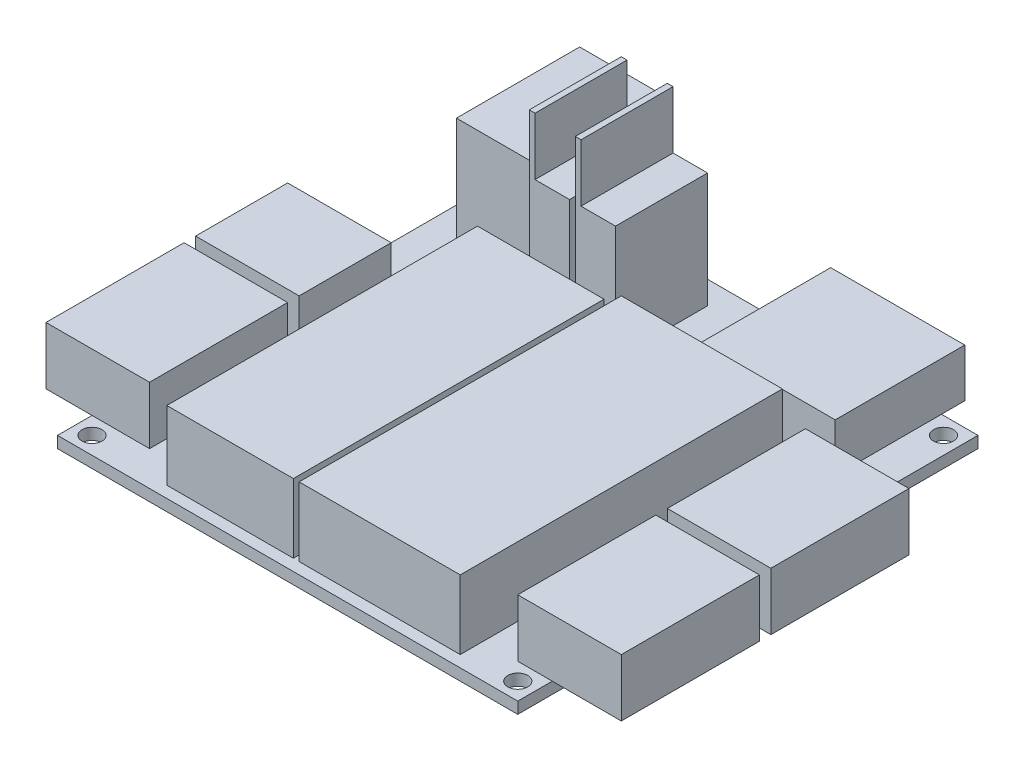
SolidWorks part; units mm, degrees
ref_plane "Front Plane" through (0, 0, 0) normal (0, 0, 1) x (1, 0, 0)
ref_plane "Top Plane" through (0, 0, 0) normal (0, 1, 0) x (1, 0, 0)
ref_plane "Right Plane" through (0, 0, 0) normal (1, 0, 0) x (0, 0, -1)
sketch "Sketch1" plane through (0, 0, 0) normal (0, 1, 0) x (1, 0, 0)
  line L0 (0, 0) -> (0, 50.8)
  line L1 (0, 50.8) -> (50.8, 50.8)
  line L2 (50.8, 50.8) -> (50.8, 0)
  line L3 (50.8, 0) -> (0, 0)
  line L4 (29.845, 40.64) -> (28.575, 40.64)
  line L5 (30.48, 43.18) -> (30.48, 38.1)
  line L6 (30.48, 38.1) -> (27.94, 38.1)
  line L7 (27.94, 38.1) -> (27.94, 43.18)
  line L8 (27.94, 43.18) -> (30.48, 43.18)
  line L9 (28.3382, 37.639) -> (28.245, 37.7322)
  line L10 (28.245, 37.7322) -> (28.0586, 37.7322)
  line L11 (28.0586, 37.7322) -> (27.9654, 37.639)
  line L12 (27.9654, 37.639) -> (27.9654, 37.2661)
  line L13 (27.9654, 37.2661) -> (28.0586, 37.1729)
  line L14 (28.0586, 37.1729) -> (28.245, 37.1729)
  line L15 (28.245, 37.1729) -> (28.3382, 37.2661)
  line L16 (28.5267, 37.5457) -> (28.7131, 37.7322)
  line L17 (28.7131, 37.7322) -> (28.7131, 37.1729)
  line L18 (28.5267, 37.1729) -> (28.8996, 37.1729)
  line L19 (28.2829, 43.8957) -> (28.4693, 44.0822)
  line L20 (28.4693, 44.0822) -> (28.4693, 43.5229)
  line L21 (28.2829, 43.5229) -> (28.6557, 43.5229)
  line L22 (28.8442, 43.6161) -> (28.8442, 43.989)
  line L23 (28.8442, 43.989) -> (28.9374, 44.0822)
  line L24 (28.9374, 44.0822) -> (29.1238, 44.0822)
  line L25 (29.1238, 44.0822) -> (29.2171, 43.989)
  line L26 (29.2171, 43.989) -> (29.2171, 43.6161)
  line L27 (29.2171, 43.6161) -> (29.1238, 43.5229)
  line L28 (29.1238, 43.5229) -> (28.9374, 43.5229)
  line L29 (28.9374, 43.5229) -> (28.8442, 43.6161)
  line L30 (28.8442, 43.6161) -> (29.2171, 43.989)
  line L31 (29.4055, 43.8957) -> (29.4055, 43.6161)
  line L32 (29.4055, 43.6161) -> (29.4987, 43.5229)
  line L33 (29.4987, 43.5229) -> (29.7784, 43.5229)
  line L34 (29.7784, 43.5229) -> (29.7784, 43.8957)
  line L35 (29.9668, 43.5229) -> (29.9668, 44.0822)
  line L36 (29.9668, 44.0822) -> (30.3397, 44.0822)
  line L37 (29.9668, 43.8025) -> (30.1533, 43.8025)
  line L38 (24.765, 40.64) -> (26.035, 40.64)
  line L39 (24.13, 38.1) -> (24.13, 43.18)
  line L40 (24.13, 43.18) -> (26.67, 43.18)
  line L41 (26.67, 43.18) -> (26.67, 38.1)
  line L42 (26.67, 38.1) -> (24.13, 38.1)
  line L43 (24.6756, 37.6644) -> (24.5824, 37.7576)
  line L44 (24.5824, 37.7576) -> (24.396, 37.7576)
  line L45 (24.396, 37.7576) -> (24.3028, 37.6644)
  line L46 (24.3028, 37.6644) -> (24.3028, 37.2915)
  line L47 (24.3028, 37.2915) -> (24.396, 37.1983)
  line L48 (24.396, 37.1983) -> (24.5824, 37.1983)
  line L49 (24.5824, 37.1983) -> (24.6756, 37.2915)
  line L50 (25.2369, 37.1983) -> (24.8641, 37.1983)
  line L51 (24.8641, 37.1983) -> (25.2369, 37.5711)
  line L52 (25.2369, 37.5711) -> (25.2369, 37.6644)
  line L53 (25.2369, 37.6644) -> (25.1437, 37.7576)
  line L54 (25.1437, 37.7576) -> (24.9573, 37.7576)
  line L55 (24.9573, 37.7576) -> (24.8641, 37.6644)
  line L56 (24.1326, 43.9211) -> (24.3191, 44.1076)
  line L57 (24.3191, 44.1076) -> (24.3191, 43.5483)
  line L58 (24.1326, 43.5483) -> (24.5055, 43.5483)
  line L59 (24.694, 43.6415) -> (24.694, 44.0144)
  line L60 (24.694, 44.0144) -> (24.7872, 44.1076)
  line L61 (24.7872, 44.1076) -> (24.9736, 44.1076)
  line L62 (24.9736, 44.1076) -> (25.0668, 44.0144)
  line L63 (25.0668, 44.0144) -> (25.0668, 43.6415)
  line L64 (25.0668, 43.6415) -> (24.9736, 43.5483)
  line L65 (24.9736, 43.5483) -> (24.7872, 43.5483)
  line L66 (24.7872, 43.5483) -> (24.694, 43.6415)
  line L67 (24.694, 43.6415) -> (25.0668, 44.0144)
  line L68 (25.2553, 43.9211) -> (25.2553, 43.6415)
  line L69 (25.2553, 43.6415) -> (25.3485, 43.5483)
  line L70 (25.3485, 43.5483) -> (25.6281, 43.5483)
  line L71 (25.6281, 43.5483) -> (25.6281, 43.9211)
  line L72 (25.8166, 43.5483) -> (25.8166, 44.1076)
  line L73 (25.8166, 44.1076) -> (26.1894, 44.1076)
  line L74 (25.8166, 43.8279) -> (26.003, 43.8279)
  line L75 (15.748, 34.29) -> (19.812, 34.29)
  line L76 (15.748, 34.29) -> (15.748, 31.75)
  line L77 (19.812, 31.75) -> (15.748, 31.75)
  line L78 (19.812, 31.75) -> (19.812, 34.29)
  line L79 (12.7, 33.02) -> (13.716, 33.02)
  line L80 (22.86, 33.02) -> (21.844, 33.02)
  line L81 (18.415, 33.02) -> (17.78, 33.02)
  line L82 (16.764, 32.385) -> (16.764, 33.655)
  line L83 (16.764, 33.655) -> (17.78, 33.02)
  line L84 (17.78, 33.02) -> (16.256, 33.02)
  line L85 (17.78, 33.02) -> (16.764, 32.385)
  line L86 (17.78, 32.385) -> (17.78, 33.02)
  line L87 (17.78, 33.02) -> (17.78, 33.655)
  line L88 (12.8591, 35.3702) -> (13.2404, 35.7515)
  line L89 (13.2404, 35.7515) -> (13.2404, 34.6075)
  line L90 (12.8591, 34.6075) -> (13.6217, 34.6075)
  line L91 (14.0285, 34.6075) -> (14.0285, 35.7515)
  line L92 (14.0285, 35.7515) -> (14.7912, 34.6075)
  line L93 (14.7912, 34.6075) -> (14.7912, 35.7515)
  line L94 (15.7699, 34.6075) -> (15.7699, 35.7515)
  line L95 (15.7699, 35.7515) -> (15.1979, 35.1795)
  line L96 (15.1979, 35.1795) -> (15.9605, 35.1795)
  line L97 (16.3673, 34.7982) -> (16.3673, 35.5608)
  line L98 (16.3673, 35.5608) -> (16.558, 35.7515)
  line L99 (16.558, 35.7515) -> (16.9393, 35.7515)
  line L100 (16.9393, 35.7515) -> (17.1299, 35.5608)
  line L101 (17.1299, 35.5608) -> (17.1299, 34.7982)
  line L102 (17.1299, 34.7982) -> (16.9393, 34.6075)
  line L103 (16.9393, 34.6075) -> (16.558, 34.6075)
  line L104 (16.558, 34.6075) -> (16.3673, 34.7982)
  line L105 (16.3673, 34.7982) -> (17.1299, 35.5608)
  line L106 (17.5367, 34.7982) -> (17.5367, 35.5608)
  line L107 (17.5367, 35.5608) -> (17.7273, 35.7515)
  line L108 (17.7273, 35.7515) -> (18.1087, 35.7515)
  line L109 (18.1087, 35.7515) -> (18.2993, 35.5608)
  line L110 (18.2993, 35.5608) -> (18.2993, 34.7982)
  line L111 (18.2993, 34.7982) -> (18.1087, 34.6075)
  line L112 (18.1087, 34.6075) -> (17.7273, 34.6075)
  line L113 (17.7273, 34.6075) -> (17.5367, 34.7982)
  line L114 (17.5367, 34.7982) -> (18.2993, 35.5608)
  line L115 (18.7061, 35.3702) -> (19.0874, 35.7515)
  line L116 (19.0874, 35.7515) -> (19.0874, 34.6075)
  line L117 (18.7061, 34.6075) -> (19.4687, 34.6075)
  line L118 (4.39, 39.64) -> (6.49, 39.64)
  line L119 (13.39, 50.34) -> (13.39, 53.24)
  line L120 (4.39, 53.24) -> (4.39, 50.34)
  line L121 (4.39, 53.24) -> (13.39, 53.24)
  line L122 (4.39, 50.34) -> (4.39, 45.04)
  line L123 (4.39, 39.64) -> (4.39, 40.34)
  line L124 (13.39, 50.34) -> (13.39, 39.64)
  line L125 (13.39, 39.64) -> (11.29, 39.64)
  line L126 (13.39, 50.34) -> (4.39, 50.34)
  line L127 (11.5901, 47.9299) -> (11.6536, 47.8663)
  line L128 (11.6536, 47.8663) -> (11.7172, 47.8663)
  line L129 (11.7172, 47.8663) -> (11.7807, 47.9299)
  line L130 (11.7807, 47.9299) -> (11.7807, 48.2476)
  line L131 (11.7172, 48.2476) -> (11.8443, 48.2476)
  line L132 (11.9643, 47.8663) -> (11.9643, 48.2476)
  line L133 (11.9643, 48.2476) -> (12.1549, 48.2476)
  line L134 (12.1549, 48.2476) -> (12.2185, 48.1841)
  line L135 (12.2185, 48.1841) -> (12.2185, 48.057)
  line L136 (12.2185, 48.057) -> (12.1549, 47.9934)
  line L137 (12.1549, 47.9934) -> (11.9643, 47.9934)
  line L138 (12.3385, 48.1205) -> (12.4656, 48.2476)
  line L139 (12.4656, 48.2476) -> (12.4656, 47.8663)
  line L140 (12.3385, 47.8663) -> (12.5927, 47.8663)
  line L141 (7.848, 49.1363) -> (7.848, 49.5176)
  line L142 (7.848, 49.5176) -> (8.0387, 49.5176)
  line L143 (8.0387, 49.5176) -> (8.1022, 49.4541)
  line L144 (8.1022, 49.4541) -> (8.1022, 49.327)
  line L145 (8.1022, 49.327) -> (8.0387, 49.2634)
  line L146 (8.0387, 49.2634) -> (7.848, 49.2634)
  line L147 (8.4129, 49.5176) -> (8.2858, 49.5176)
  line L148 (8.2858, 49.5176) -> (8.2222, 49.4541)
  line L149 (8.2222, 49.4541) -> (8.2222, 49.1999)
  line L150 (8.2222, 49.1999) -> (8.2858, 49.1363)
  line L151 (8.2858, 49.1363) -> (8.4129, 49.1363)
  line L152 (8.4129, 49.1363) -> (8.4764, 49.1999)
  line L153 (8.4764, 49.1999) -> (8.4764, 49.4541)
  line L154 (8.4764, 49.4541) -> (8.4129, 49.5176)
  line L155 (8.5964, 49.5176) -> (8.5964, 49.1363)
  line L156 (8.5964, 49.1363) -> (8.7235, 49.2634)
  line L157 (8.7235, 49.2634) -> (8.8506, 49.1363)
  line L158 (8.8506, 49.1363) -> (8.8506, 49.5176)
  line L159 (9.2248, 49.5176) -> (8.9706, 49.5176)
  line L160 (8.9706, 49.5176) -> (8.9706, 49.1363)
  line L161 (8.9706, 49.1363) -> (9.2248, 49.1363)
  line L162 (8.9706, 49.327) -> (9.0977, 49.327)
  line L163 (9.3448, 49.1363) -> (9.3448, 49.5176)
  line L164 (9.3448, 49.5176) -> (9.5355, 49.5176)
  line L165 (9.5355, 49.5176) -> (9.599, 49.4541)
  line L166 (9.599, 49.4541) -> (9.599, 49.327)
  line L167 (9.599, 49.327) -> (9.5355, 49.2634)
  line L168 (9.5355, 49.2634) -> (9.3448, 49.2634)
  line L169 (9.4719, 49.2634) -> (9.599, 49.1363)
  line L170 (9.719, 49.0727) -> (9.9733, 49.0727)
  line L171 (10.0932, 49.1999) -> (10.1568, 49.1363)
  line L172 (10.1568, 49.1363) -> (10.2204, 49.1363)
  line L173 (10.2204, 49.1363) -> (10.2839, 49.1999)
  line L174 (10.2839, 49.1999) -> (10.2839, 49.5176)
  line L175 (10.2204, 49.5176) -> (10.3475, 49.5176)
  line L176 (10.4674, 49.1363) -> (10.4674, 49.3905)
  line L177 (10.4674, 49.3905) -> (10.5945, 49.5176)
  line L178 (10.5945, 49.5176) -> (10.7217, 49.3905)
  line L179 (10.7217, 49.3905) -> (10.7217, 49.1363)
  line L180 (10.4674, 49.327) -> (10.7217, 49.327)
  line L181 (11.0959, 49.4541) -> (11.0323, 49.5176)
  line L182 (11.0323, 49.5176) -> (10.9052, 49.5176)
  line L183 (10.9052, 49.5176) -> (10.8417, 49.4541)
  line L184 (10.8417, 49.4541) -> (10.8417, 49.1999)
  line L185 (10.8417, 49.1999) -> (10.9052, 49.1363)
  line L186 (10.9052, 49.1363) -> (11.0323, 49.1363)
  line L187 (11.0323, 49.1363) -> (11.0959, 49.1999)
  line L188 (11.2159, 49.5176) -> (11.2159, 49.1363)
  line L189 (11.2159, 49.2634) -> (11.4701, 49.5176)
  line L190 (11.2794, 49.327) -> (11.4701, 49.1363)
  line L191 (11.5901, 49.1363) -> (11.5901, 49.5176)
  line L192 (11.5901, 49.5176) -> (11.7807, 49.5176)
  line L193 (11.7807, 49.5176) -> (11.8443, 49.4541)
  line L194 (11.8443, 49.4541) -> (11.8443, 49.327)
  line L195 (11.8443, 49.327) -> (11.7807, 49.2634)
  line L196 (11.7807, 49.2634) -> (11.5901, 49.2634)
  line L197 (12.0914, 49.1363) -> (12.0914, 49.5176)
  line L198 (11.9643, 49.5176) -> (12.2185, 49.5176)
  line L199 (12.3385, 49.1363) -> (12.3385, 49.5176)
  line L200 (12.3385, 49.327) -> (12.5927, 49.327)
  line L201 (12.5927, 49.5176) -> (12.5927, 49.1363)
  line L202 (10.795, 1.27) -> (24.765, 1.27)
  line L203 (24.765, 1.27) -> (24.765, 35.56)
  line L204 (24.765, 35.56) -> (10.795, 35.56)
  line L205 (10.795, 35.56) -> (10.795, 1.27)
  line L206 (14.1986, 3.8354) -> (13.6393, 3.8354)
  line L207 (13.6393, 3.8354) -> (13.6393, 4.115)
  line L208 (13.6393, 4.115) -> (13.7325, 4.2082)
  line L209 (13.7325, 4.2082) -> (13.919, 4.2082)
  line L210 (13.919, 4.2082) -> (14.0122, 4.115)
  line L211 (14.0122, 4.115) -> (14.0122, 3.8354)
  line L212 (14.0122, 4.0218) -> (14.1986, 4.2082)
  line L213 (13.6393, 4.3967) -> (14.1986, 4.7696)
  line L214 (13.6393, 4.7696) -> (14.1986, 4.3967)
  line L215 (16.7386, 4.0218) -> (16.1793, 4.0218)
  line L216 (16.1793, 3.8354) -> (16.1793, 4.2082)
  line L217 (16.1793, 4.3967) -> (16.7386, 4.7696)
  line L218 (16.1793, 4.7696) -> (16.7386, 4.3967)
  line L219 (18.8125, 4.2082) -> (18.7193, 4.115)
  line L220 (18.7193, 4.115) -> (18.7193, 3.9286)
  line L221 (18.7193, 3.9286) -> (18.8125, 3.8354)
  line L222 (18.8125, 3.8354) -> (19.1854, 3.8354)
  line L223 (19.1854, 3.8354) -> (19.2786, 3.9286)
  line L224 (19.2786, 3.9286) -> (19.2786, 4.115)
  line L225 (19.2786, 4.115) -> (19.1854, 4.2082)
  line L226 (19.1854, 4.2082) -> (18.999, 4.2082)
  line L227 (18.999, 4.2082) -> (18.999, 4.0218)
  line L228 (19.2786, 4.3967) -> (18.7193, 4.3967)
  line L229 (18.7193, 4.3967) -> (19.2786, 4.7696)
  line L230 (19.2786, 4.7696) -> (18.7193, 4.7696)
  line L231 (18.7193, 4.958) -> (19.2786, 4.958)
  line L232 (19.2786, 4.958) -> (19.2786, 5.2377)
  line L233 (19.2786, 5.2377) -> (19.1854, 5.3309)
  line L234 (19.1854, 5.3309) -> (18.8125, 5.3309)
  line L235 (18.8125, 5.3309) -> (18.7193, 5.2377)
  line L236 (18.7193, 5.2377) -> (18.7193, 4.958)
  line L237 (21.2593, 3.8354) -> (21.6322, 3.8354)
  line L238 (21.6322, 3.8354) -> (21.8186, 4.0218)
  line L239 (21.8186, 4.0218) -> (21.6322, 4.2082)
  line L240 (21.6322, 4.2082) -> (21.2593, 4.2082)
  line L241 (21.3525, 4.7696) -> (21.2593, 4.6763)
  line L242 (21.2593, 4.6763) -> (21.2593, 4.4899)
  line L243 (21.2593, 4.4899) -> (21.3525, 4.3967)
  line L244 (21.3525, 4.3967) -> (21.7254, 4.3967)
  line L245 (21.7254, 4.3967) -> (21.8186, 4.4899)
  line L246 (21.8186, 4.4899) -> (21.8186, 4.6763)
  line L247 (21.8186, 4.6763) -> (21.7254, 4.7696)
  line L248 (21.3525, 5.3309) -> (21.2593, 5.2377)
  line L249 (21.2593, 5.2377) -> (21.2593, 5.0512)
  line L250 (21.2593, 5.0512) -> (21.3525, 4.958)
  line L251 (21.3525, 4.958) -> (21.7254, 4.958)
  line L252 (21.7254, 4.958) -> (21.8186, 5.0512)
  line L253 (21.8186, 5.0512) -> (21.8186, 5.2377)
  line L254 (21.8186, 5.2377) -> (21.7254, 5.3309)
  line L255 (10.0752, 1.3335) -> (10.2235, 1.4818)
  line L256 (10.2235, 1.4818) -> (10.2235, 1.6301)
  line L257 (10.2235, 1.6301) -> (10.0752, 1.7784)
  line L258 (10.0752, 1.7784) -> (9.3337, 1.7784)
  line L259 (9.3337, 1.6301) -> (9.3337, 1.9267)
  line L260 (10.3718, 2.269) -> (10.3718, 2.8622)
  line L261 (10.2235, 3.2045) -> (9.3337, 3.2045)
  line L262 (9.3337, 3.2045) -> (9.3337, 3.6494)
  line L263 (9.3337, 3.6494) -> (9.482, 3.7977)
  line L264 (9.482, 3.7977) -> (9.6303, 3.7977)
  line L265 (9.6303, 3.7977) -> (9.7786, 3.6494)
  line L266 (9.7786, 3.6494) -> (9.9269, 3.7977)
  line L267 (9.9269, 3.7977) -> (10.0752, 3.7977)
  line L268 (10.0752, 3.7977) -> (10.2235, 3.6494)
  line L269 (10.2235, 3.6494) -> (10.2235, 3.2045)
  line L270 (9.7786, 3.2045) -> (9.7786, 3.6494)
  line L271 (10.2235, 4.4366) -> (9.3337, 4.4366)
  line L272 (9.3337, 4.14) -> (9.3337, 4.7332)
  line L273 (10.3718, 5.0756) -> (10.3718, 5.6687)
  line L274 (10.2235, 6.0111) -> (9.3337, 6.0111)
  line L275 (9.3337, 6.0111) -> (9.3337, 6.456)
  line L276 (9.3337, 6.456) -> (9.482, 6.6043)
  line L277 (9.482, 6.6043) -> (9.6303, 6.6043)
  line L278 (9.6303, 6.6043) -> (9.7786, 6.456)
  line L279 (9.7786, 6.456) -> (9.9269, 6.6043)
  line L280 (9.9269, 6.6043) -> (10.0752, 6.6043)
  line L281 (10.0752, 6.6043) -> (10.2235, 6.456)
  line L282 (10.2235, 6.456) -> (10.2235, 6.0111)
  line L283 (9.7786, 6.0111) -> (9.7786, 6.456)
  line L284 (9.3337, 7.3915) -> (9.3337, 7.0949)
  line L285 (9.3337, 7.0949) -> (9.482, 6.9466)
  line L286 (9.482, 6.9466) -> (10.0752, 6.9466)
  line L287 (10.0752, 6.9466) -> (10.2235, 7.0949)
  line L288 (10.2235, 7.0949) -> (10.2235, 7.3915)
  line L289 (10.2235, 7.3915) -> (10.0752, 7.5398)
  line L290 (10.0752, 7.5398) -> (9.482, 7.5398)
  line L291 (9.482, 7.5398) -> (9.3337, 7.3915)
  line L292 (10.2235, 7.8821) -> (9.6303, 7.8821)
  line L293 (9.6303, 7.8821) -> (9.3337, 8.1787)
  line L294 (9.3337, 8.1787) -> (9.6303, 8.4753)
  line L295 (9.6303, 8.4753) -> (10.2235, 8.4753)
  line L296 (9.7786, 7.8821) -> (9.7786, 8.4753)
  line L297 (10.2235, 8.8177) -> (9.3337, 8.8177)
  line L298 (9.3337, 8.8177) -> (9.3337, 9.2625)
  line L299 (9.3337, 9.2625) -> (9.482, 9.4108)
  line L300 (9.482, 9.4108) -> (9.7786, 9.4108)
  line L301 (9.7786, 9.4108) -> (9.9269, 9.2625)
  line L302 (9.9269, 9.2625) -> (9.9269, 8.8177)
  line L303 (9.9269, 9.1142) -> (10.2235, 9.4108)
  line L304 (9.3337, 9.7532) -> (10.2235, 9.7532)
  line L305 (10.2235, 9.7532) -> (10.2235, 10.198)
  line L306 (10.2235, 10.198) -> (10.0752, 10.3463)
  line L307 (10.0752, 10.3463) -> (9.482, 10.3463)
  line L308 (9.482, 10.3463) -> (9.3337, 10.198)
  line L309 (9.3337, 10.198) -> (9.3337, 9.7532)
  line L310 (10.3718, 10.6887) -> (10.3718, 11.2819)
  line L311 (9.6303, 11.6242) -> (9.3337, 11.9208)
  line L312 (9.3337, 11.9208) -> (10.2235, 11.9208)
  line L313 (10.2235, 11.6242) -> (10.2235, 12.2174)
  line L314 (3.81, 35.8648) -> (1.27, 35.8648)
  line L315 (0.9515, 36.2585) -> (2.0955, 36.2585)
  line L316 (2.0955, 36.2585) -> (2.0955, 37.0212)
  line L317 (0.9515, 38.1906) -> (0.9515, 37.4279)
  line L318 (0.9515, 37.4279) -> (2.0955, 37.4279)
  line L319 (2.0955, 37.4279) -> (2.0955, 38.1906)
  line L320 (1.5235, 37.4279) -> (1.5235, 37.8092)
  line L321 (0.9515, 38.5973) -> (2.0955, 38.5973)
  line L322 (2.0955, 38.5973) -> (2.0955, 39.1693)
  line L323 (2.0955, 39.1693) -> (1.9048, 39.3599)
  line L324 (1.9048, 39.3599) -> (1.1422, 39.3599)
  line L325 (1.1422, 39.3599) -> (0.9515, 39.1693)
  line L326 (0.9515, 39.1693) -> (0.9515, 38.5973)
  line L327 (1.3328, 39.7667) -> (0.9515, 40.148)
  line L328 (0.9515, 40.148) -> (2.0955, 40.148)
  line L329 (2.0955, 39.7667) -> (2.0955, 40.5293)
  line L330 (2.6768, 32.6898) -> (2.4032, 32.6898)
  line L331 (2.4032, 32.6898) -> (2.2098, 32.8832)
  line L332 (2.2098, 32.8832) -> (2.2098, 33.1568)
  line L333 (2.2098, 33.1568) -> (2.4032, 33.3502)
  line L334 (2.4032, 33.3502) -> (2.6768, 33.3502)
  line L335 (2.6768, 33.3502) -> (2.8702, 33.1568)
  line L336 (2.8702, 33.1568) -> (2.8702, 32.8832)
  line L337 (2.8702, 32.8832) -> (2.6768, 32.6898)
  line L338 (2.6768, 32.6898) -> (2.4032, 32.6898)
  line L339 (2.6768, 32.6898) -> (2.4032, 32.6898)
  line L340 (2.4032, 32.6898) -> (2.2098, 32.8832)
  line L341 (2.2098, 32.8832) -> (2.2098, 33.1568)
  line L342 (2.2098, 33.1568) -> (2.4032, 33.3502)
  line L343 (2.4032, 33.3502) -> (2.6768, 33.3502)
  line L344 (2.6768, 33.3502) -> (2.8702, 33.1568)
  line L345 (2.8702, 33.1568) -> (2.8702, 32.8832)
  line L346 (2.8702, 32.8832) -> (2.6768, 32.6898)
  line L347 (2.6768, 32.6898) -> (2.4032, 32.6898)
  line L348 (2.6768, 35.2298) -> (2.4032, 35.2298)
  line L349 (2.4032, 35.2298) -> (2.2098, 35.4232)
  line L350 (2.2098, 35.4232) -> (2.2098, 35.6968)
  line L351 (2.2098, 35.6968) -> (2.4032, 35.8902)
  line L352 (2.4032, 35.8902) -> (2.6768, 35.8902)
  line L353 (2.6768, 35.8902) -> (2.8702, 35.6968)
  line L354 (2.8702, 35.6968) -> (2.8702, 35.4232)
  line L355 (2.8702, 35.4232) -> (2.6768, 35.2298)
  line L356 (2.6768, 35.2298) -> (2.4032, 35.2298)
  line L357 (2.6768, 35.2298) -> (2.4032, 35.2298)
  line L358 (2.4032, 35.2298) -> (2.2098, 35.4232)
  line L359 (2.2098, 35.4232) -> (2.2098, 35.6968)
  line L360 (2.2098, 35.6968) -> (2.4032, 35.8902)
  line L361 (2.4032, 35.8902) -> (2.6768, 35.8902)
  line L362 (2.6768, 35.8902) -> (2.8702, 35.6968)
  line L363 (2.8702, 35.6968) -> (2.8702, 35.4232)
  line L364 (2.8702, 35.4232) -> (2.6768, 35.2298)
  line L365 (2.6768, 35.2298) -> (2.4032, 35.2298)
  line L366 (10.16, 36.83) -> (10.16, 31.75)
  line L367 (10.16, 31.75) -> (5.08, 31.75)
  line L368 (5.08, 31.75) -> (5.08, 36.83)
  line L369 (5.08, 36.83) -> (10.16, 36.83)
  line L370 (8.9275, 32.8596) -> (8.9275, 32.6139)
  line L371 (8.9275, 32.6139) -> (9.0504, 32.491)
  line L372 (9.0504, 32.491) -> (9.5418, 32.491)
  line L373 (9.5418, 32.491) -> (9.6647, 32.6139)
  line L374 (9.6647, 32.6139) -> (9.6647, 32.8596)
  line L375 (9.6647, 32.8596) -> (9.5418, 32.9825)
  line L376 (9.5418, 32.9825) -> (9.0504, 32.9825)
  line L377 (9.0504, 32.9825) -> (8.9275, 32.8596)
  line L378 (9.6647, 33.2394) -> (8.9275, 33.2394)
  line L379 (8.9275, 33.2394) -> (9.6647, 33.7309)
  line L380 (9.6647, 33.7309) -> (8.9275, 33.7309)
  line L381 (8.9275, 34.3565) -> (8.9275, 34.1107)
  line L382 (8.9275, 34.1107) -> (9.0504, 33.9878)
  line L383 (9.0504, 33.9878) -> (9.5418, 33.9878)
  line L384 (9.5418, 33.9878) -> (9.6647, 34.1107)
  line L385 (9.6647, 34.1107) -> (9.6647, 34.3565)
  line L386 (9.6647, 34.3565) -> (9.5418, 34.4793)
  line L387 (9.5418, 34.4793) -> (9.0504, 34.4793)
  line L388 (9.0504, 34.4793) -> (8.9275, 34.3565)
  line L389 (9.6647, 34.7363) -> (8.9275, 34.7363)
  line L390 (8.9275, 34.7363) -> (8.9275, 35.2277)
  line L391 (9.2961, 34.7363) -> (9.2961, 34.982)
  line L392 (9.6647, 35.4847) -> (8.9275, 35.4847)
  line L393 (8.9275, 35.4847) -> (8.9275, 35.9762)
  line L394 (9.2961, 35.4847) -> (9.2961, 35.7304)
  line L395 (5.7525, 31.7426) -> (6.4897, 31.7426)
  line L396 (6.4897, 31.7426) -> (6.4897, 32.1112)
  line L397 (6.4897, 32.1112) -> (6.3668, 32.2341)
  line L398 (6.3668, 32.2341) -> (5.8754, 32.2341)
  line L399 (5.8754, 32.2341) -> (5.7525, 32.1112)
  line L400 (5.7525, 32.1112) -> (5.7525, 31.7426)
  line L401 (5.8754, 32.9825) -> (5.7525, 32.8596)
  line L402 (5.7525, 32.8596) -> (5.7525, 32.6139)
  line L403 (5.7525, 32.6139) -> (5.8754, 32.491)
  line L404 (5.8754, 32.491) -> (5.9982, 32.491)
  line L405 (5.9982, 32.491) -> (6.1211, 32.6139)
  line L406 (6.1211, 32.6139) -> (6.1211, 32.8596)
  line L407 (6.1211, 32.8596) -> (6.244, 32.9825)
  line L408 (6.244, 32.9825) -> (6.3668, 32.9825)
  line L409 (6.3668, 32.9825) -> (6.4897, 32.8596)
  line L410 (6.4897, 32.8596) -> (6.4897, 32.6139)
  line L411 (6.4897, 32.6139) -> (6.3668, 32.491)
  line L412 (6.1211, 33.2394) -> (6.1211, 33.7309)
  line L413 (6.4897, 34.4793) -> (6.4897, 33.9878)
  line L414 (6.4897, 33.9878) -> (5.9982, 34.4793)
  line L415 (5.9982, 34.4793) -> (5.8754, 34.4793)
  line L416 (5.8754, 34.4793) -> (5.7525, 34.3565)
  line L417 (5.7525, 34.3565) -> (5.7525, 34.1107)
  line L418 (5.7525, 34.1107) -> (5.8754, 33.9878)
  line L419 (6.4897, 35.2277) -> (6.4897, 34.7363)
  line L420 (6.4897, 34.7363) -> (5.9982, 35.2277)
  line L421 (5.9982, 35.2277) -> (5.8754, 35.2277)
  line L422 (5.8754, 35.2277) -> (5.7525, 35.1049)
  line L423 (5.7525, 35.1049) -> (5.7525, 34.8591)
  line L424 (5.7525, 34.8591) -> (5.8754, 34.7363)
  line L425 (5.8754, 35.4847) -> (5.7525, 35.6075)
  line L426 (5.7525, 35.6075) -> (5.7525, 35.8533)
  line L427 (5.7525, 35.8533) -> (5.8754, 35.9762)
  line L428 (5.8754, 35.9762) -> (5.9982, 35.9762)
  line L429 (5.9982, 35.9762) -> (6.1211, 35.8533)
  line L430 (6.1211, 35.8533) -> (6.244, 35.9762)
  line L431 (6.244, 35.9762) -> (6.3668, 35.9762)
  line L432 (6.3668, 35.9762) -> (6.4897, 35.8533)
  line L433 (6.4897, 35.8533) -> (6.4897, 35.6075)
  line L434 (6.4897, 35.6075) -> (6.3668, 35.4847)
  line L435 (6.3668, 35.4847) -> (6.244, 35.4847)
  line L436 (6.244, 35.4847) -> (6.1211, 35.6075)
  line L437 (6.1211, 35.6075) -> (5.9982, 35.4847)
  line L438 (5.9982, 35.4847) -> (5.8754, 35.4847)
  line L439 (6.1211, 35.6075) -> (6.1211, 35.8533)
  line L440 (15.24, 21.082) -> (20.32, 21.082)
  line L441 (20.32, 21.082) -> (20.32, 20.32)
  line L442 (20.32, 20.32) -> (20.32, 19.558)
  line L443 (20.32, 19.558) -> (15.24, 19.558)
  line L444 (15.24, 19.558) -> (15.24, 20.32)
  line L445 (15.24, 20.32) -> (15.24, 21.082)
  line L446 (20.32, 20.32) -> (20.574, 20.32)
  line L447 (15.24, 20.32) -> (14.986, 20.32)
  line L448 (15.2527, 21.6027) -> (15.2527, 21.984)
  line L449 (15.2527, 21.984) -> (15.4434, 21.984)
  line L450 (15.4434, 21.984) -> (15.5069, 21.9205)
  line L451 (15.5069, 21.9205) -> (15.5069, 21.7934)
  line L452 (15.5069, 21.7934) -> (15.4434, 21.7298)
  line L453 (15.4434, 21.7298) -> (15.2527, 21.7298)
  line L454 (15.3798, 21.7298) -> (15.5069, 21.6027)
  line L455 (15.6269, 21.8569) -> (15.754, 21.984)
  line L456 (15.754, 21.984) -> (15.754, 21.6027)
  line L457 (15.6269, 21.6027) -> (15.8811, 21.6027)
  line L458 (15.8242, 20.5914) -> (16.1123, 20.8795)
  line L459 (16.1123, 20.8795) -> (16.1123, 20.0152)
  line L460 (15.8242, 20.0152) -> (16.4004, 20.0152)
  line L461 (16.7597, 20.1593) -> (16.7597, 20.7355)
  line L462 (16.7597, 20.7355) -> (16.9038, 20.8795)
  line L463 (16.9038, 20.8795) -> (17.1919, 20.8795)
  line L464 (17.1919, 20.8795) -> (17.3359, 20.7355)
  line L465 (17.3359, 20.7355) -> (17.3359, 20.1593)
  line L466 (17.3359, 20.1593) -> (17.1919, 20.0152)
  line L467 (17.1919, 20.0152) -> (16.9038, 20.0152)
  line L468 (16.9038, 20.0152) -> (16.7597, 20.1593)
  line L469 (16.7597, 20.1593) -> (17.3359, 20.7355)
  line L470 (17.6952, 20.8795) -> (17.6952, 20.0152)
  line L471 (17.6952, 20.3033) -> (18.2715, 20.8795)
  line L472 (17.8393, 20.4474) -> (18.2715, 20.0152)
  line L473 (15.24, 18.542) -> (20.32, 18.542)
  line L474 (20.32, 18.542) -> (20.32, 17.78)
  line L475 (20.32, 17.78) -> (20.32, 17.018)
  line L476 (20.32, 17.018) -> (15.24, 17.018)
  line L477 (15.24, 17.018) -> (15.24, 17.78)
  line L478 (15.24, 17.78) -> (15.24, 18.542)
  line L479 (20.32, 17.78) -> (20.574, 17.78)
  line L480 (15.24, 17.78) -> (14.986, 17.78)
  line L481 (15.2527, 19.0627) -> (15.2527, 19.444)
  line L482 (15.2527, 19.444) -> (15.4434, 19.444)
  line L483 (15.4434, 19.444) -> (15.5069, 19.3805)
  line L484 (15.5069, 19.3805) -> (15.5069, 19.2534)
  line L485 (15.5069, 19.2534) -> (15.4434, 19.1898)
  line L486 (15.4434, 19.1898) -> (15.2527, 19.1898)
  line L487 (15.3798, 19.1898) -> (15.5069, 19.0627)
  line L488 (15.8811, 19.0627) -> (15.6269, 19.0627)
  line L489 (15.6269, 19.0627) -> (15.8811, 19.3169)
  line L490 (15.8811, 19.3169) -> (15.8811, 19.3805)
  line L491 (15.8811, 19.3805) -> (15.8176, 19.444)
  line L492 (15.8176, 19.444) -> (15.6905, 19.444)
  line L493 (15.6905, 19.444) -> (15.6269, 19.3805)
  line L494 (15.8242, 18.0514) -> (16.1123, 18.3395)
  line L495 (16.1123, 18.3395) -> (16.1123, 17.4752)
  line L496 (15.8242, 17.4752) -> (16.4004, 17.4752)
  line L497 (16.7597, 17.6193) -> (16.7597, 18.1955)
  line L498 (16.7597, 18.1955) -> (16.9038, 18.3395)
  line L499 (16.9038, 18.3395) -> (17.1919, 18.3395)
  line L500 (17.1919, 18.3395) -> (17.3359, 18.1955)
  line L501 (17.3359, 18.1955) -> (17.3359, 17.6193)
  line L502 (17.3359, 17.6193) -> (17.1919, 17.4752)
  line L503 (17.1919, 17.4752) -> (16.9038, 17.4752)
  line L504 (16.9038, 17.4752) -> (16.7597, 17.6193)
  line L505 (16.7597, 17.6193) -> (17.3359, 18.1955)
  line L506 (17.6952, 18.3395) -> (17.6952, 17.4752)
  line L507 (17.6952, 17.7633) -> (18.2715, 18.3395)
  line L508 (17.8393, 17.9074) -> (18.2715, 17.4752)
  line L509 (15.24, 16.002) -> (20.32, 16.002)
  line L510 (20.32, 16.002) -> (20.32, 15.24)
  line L511 (20.32, 15.24) -> (20.32, 14.478)
  line L512 (20.32, 14.478) -> (15.24, 14.478)
  line L513 (15.24, 14.478) -> (15.24, 15.24)
  line L514 (15.24, 15.24) -> (15.24, 16.002)
  line L515 (20.32, 15.24) -> (20.574, 15.24)
  line L516 (15.24, 15.24) -> (14.986, 15.24)
  line L517 (15.2527, 16.5227) -> (15.2527, 16.904)
  line L518 (15.2527, 16.904) -> (15.4434, 16.904)
  line L519 (15.4434, 16.904) -> (15.5069, 16.8405)
  line L520 (15.5069, 16.8405) -> (15.5069, 16.7134)
  line L521 (15.5069, 16.7134) -> (15.4434, 16.6498)
  line L522 (15.4434, 16.6498) -> (15.2527, 16.6498)
  line L523 (15.3798, 16.6498) -> (15.5069, 16.5227)
  line L524 (15.6269, 16.8405) -> (15.6905, 16.904)
  line L525 (15.6905, 16.904) -> (15.8176, 16.904)
  line L526 (15.8176, 16.904) -> (15.8811, 16.8405)
  line L527 (15.8811, 16.8405) -> (15.8811, 16.7769)
  line L528 (15.8811, 16.7769) -> (15.8176, 16.7134)
  line L529 (15.8176, 16.7134) -> (15.754, 16.7134)
  line L530 (15.8176, 16.7134) -> (15.8811, 16.6498)
  line L531 (15.8811, 16.6498) -> (15.8811, 16.5863)
  line L532 (15.8811, 16.5863) -> (15.8176, 16.5227)
  line L533 (15.8176, 16.5227) -> (15.6905, 16.5227)
  line L534 (15.6905, 16.5227) -> (15.6269, 16.5863)
  line L535 (15.8242, 15.5114) -> (16.1123, 15.7995)
  line L536 (16.1123, 15.7995) -> (16.1123, 14.9352)
  line L537 (15.8242, 14.9352) -> (16.4004, 14.9352)
  line L538 (16.7597, 15.0793) -> (16.7597, 15.6555)
  line L539 (16.7597, 15.6555) -> (16.9038, 15.7995)
  line L540 (16.9038, 15.7995) -> (17.1919, 15.7995)
  line L541 (17.1919, 15.7995) -> (17.3359, 15.6555)
  line L542 (17.3359, 15.6555) -> (17.3359, 15.0793)
  line L543 (17.3359, 15.0793) -> (17.1919, 14.9352)
  line L544 (17.1919, 14.9352) -> (16.9038, 14.9352)
  line L545 (16.9038, 14.9352) -> (16.7597, 15.0793)
  line L546 (16.7597, 15.0793) -> (17.3359, 15.6555)
  line L547 (17.6952, 15.7995) -> (17.6952, 14.9352)
  line L548 (17.6952, 15.2233) -> (18.2715, 15.7995)
  line L549 (17.8393, 15.3674) -> (18.2715, 14.9352)
  line L550 (15.24, 13.462) -> (20.32, 13.462)
  line L551 (20.32, 13.462) -> (20.32, 12.7)
  line L552 (20.32, 12.7) -> (20.32, 11.938)
  line L553 (20.32, 11.938) -> (15.24, 11.938)
  line L554 (15.24, 11.938) -> (15.24, 12.7)
  line L555 (15.24, 12.7) -> (15.24, 13.462)
  line L556 (20.32, 12.7) -> (20.574, 12.7)
  line L557 (15.24, 12.7) -> (14.986, 12.7)
  line L558 (15.2527, 13.9827) -> (15.2527, 14.364)
  line L559 (15.2527, 14.364) -> (15.4434, 14.364)
  line L560 (15.4434, 14.364) -> (15.5069, 14.3005)
  line L561 (15.5069, 14.3005) -> (15.5069, 14.1734)
  line L562 (15.5069, 14.1734) -> (15.4434, 14.1098)
  line L563 (15.4434, 14.1098) -> (15.2527, 14.1098)
  line L564 (15.3798, 14.1098) -> (15.5069, 13.9827)
  line L565 (15.8176, 13.9827) -> (15.8176, 14.364)
  line L566 (15.8176, 14.364) -> (15.6269, 14.1734)
  line L567 (15.6269, 14.1734) -> (15.8811, 14.1734)
  line L568 (15.8242, 12.9714) -> (16.1123, 13.2595)
  line L569 (16.1123, 13.2595) -> (16.1123, 12.3952)
  line L570 (15.8242, 12.3952) -> (16.4004, 12.3952)
  line L571 (16.7597, 12.5393) -> (16.7597, 13.1155)
  line L572 (16.7597, 13.1155) -> (16.9038, 13.2595)
  line L573 (16.9038, 13.2595) -> (17.1919, 13.2595)
  line L574 (17.1919, 13.2595) -> (17.3359, 13.1155)
  line L575 (17.3359, 13.1155) -> (17.3359, 12.5393)
  line L576 (17.3359, 12.5393) -> (17.1919, 12.3952)
  line L577 (17.1919, 12.3952) -> (16.9038, 12.3952)
  line L578 (16.9038, 12.3952) -> (16.7597, 12.5393)
  line L579 (16.7597, 12.5393) -> (17.3359, 13.1155)
  line L580 (17.6952, 13.2595) -> (17.6952, 12.3952)
  line L581 (17.6952, 12.6833) -> (18.2715, 13.2595)
  line L582 (17.8393, 12.8274) -> (18.2715, 12.3952)
  line L583 (15.24, 10.922) -> (20.32, 10.922)
  line L584 (20.32, 10.922) -> (20.32, 10.16)
  line L585 (20.32, 10.16) -> (20.32, 9.398)
  line L586 (20.32, 9.398) -> (15.24, 9.398)
  line L587 (15.24, 9.398) -> (15.24, 10.16)
  line L588 (15.24, 10.16) -> (15.24, 10.922)
  line L589 (20.32, 10.16) -> (20.574, 10.16)
  line L590 (15.24, 10.16) -> (14.986, 10.16)
  line L591 (15.2527, 11.4427) -> (15.2527, 11.824)
  line L592 (15.2527, 11.824) -> (15.4434, 11.824)
  line L593 (15.4434, 11.824) -> (15.5069, 11.7605)
  line L594 (15.5069, 11.7605) -> (15.5069, 11.6334)
  line L595 (15.5069, 11.6334) -> (15.4434, 11.5698)
  line L596 (15.4434, 11.5698) -> (15.2527, 11.5698)
  line L597 (15.3798, 11.5698) -> (15.5069, 11.4427)
  line L598 (15.8811, 11.824) -> (15.6269, 11.824)
  line L599 (15.6269, 11.824) -> (15.6269, 11.6334)
  line L600 (15.6269, 11.6334) -> (15.754, 11.6969)
  line L601 (15.754, 11.6969) -> (15.8176, 11.6969)
  line L602 (15.8176, 11.6969) -> (15.8811, 11.6334)
  line L603 (15.8811, 11.6334) -> (15.8811, 11.5063)
  line L604 (15.8811, 11.5063) -> (15.8176, 11.4427)
  line L605 (15.8176, 11.4427) -> (15.6905, 11.4427)
  line L606 (15.6905, 11.4427) -> (15.6269, 11.5063)
  line L607 (15.8242, 10.4314) -> (16.1123, 10.7195)
  line L608 (16.1123, 10.7195) -> (16.1123, 9.8552)
  line L609 (15.8242, 9.8552) -> (16.4004, 9.8552)
  line L610 (16.7597, 9.9993) -> (16.7597, 10.5755)
  line L611 (16.7597, 10.5755) -> (16.9038, 10.7195)
  line L612 (16.9038, 10.7195) -> (17.1919, 10.7195)
  line L613 (17.1919, 10.7195) -> (17.3359, 10.5755)
  line L614 (17.3359, 10.5755) -> (17.3359, 9.9993)
  line L615 (17.3359, 9.9993) -> (17.1919, 9.8552)
  line L616 (17.1919, 9.8552) -> (16.9038, 9.8552)
  line L617 (16.9038, 9.8552) -> (16.7597, 9.9993)
  line L618 (16.7597, 9.9993) -> (17.3359, 10.5755)
  line L619 (17.6952, 10.7195) -> (17.6952, 9.8552)
  line L620 (17.6952, 10.1433) -> (18.2715, 10.7195)
  line L621 (17.8393, 10.2874) -> (18.2715, 9.8552)
  line L622 (15.24, 8.382) -> (20.32, 8.382)
  line L623 (20.32, 8.382) -> (20.32, 7.62)
  line L624 (20.32, 7.62) -> (20.32, 6.858)
  line L625 (20.32, 6.858) -> (15.24, 6.858)
  line L626 (15.24, 6.858) -> (15.24, 7.62)
  line L627 (15.24, 7.62) -> (15.24, 8.382)
  line L628 (20.32, 7.62) -> (20.574, 7.62)
  line L629 (15.24, 7.62) -> (14.986, 7.62)
  line L630 (15.2527, 8.9027) -> (15.2527, 9.284)
  line L631 (15.2527, 9.284) -> (15.4434, 9.284)
  line L632 (15.4434, 9.284) -> (15.5069, 9.2205)
  line L633 (15.5069, 9.2205) -> (15.5069, 9.0934)
  line L634 (15.5069, 9.0934) -> (15.4434, 9.0298)
  line L635 (15.4434, 9.0298) -> (15.2527, 9.0298)
  line L636 (15.3798, 9.0298) -> (15.5069, 8.9027)
  line L637 (15.8811, 9.284) -> (15.754, 9.2205)
  line L638 (15.754, 9.2205) -> (15.6269, 9.0934)
  line L639 (15.6269, 9.0934) -> (15.6269, 8.9663)
  line L640 (15.6269, 8.9663) -> (15.6905, 8.9027)
  line L641 (15.6905, 8.9027) -> (15.8176, 8.9027)
  line L642 (15.8176, 8.9027) -> (15.8811, 8.9663)
  line L643 (15.8811, 8.9663) -> (15.8811, 9.0298)
  line L644 (15.8811, 9.0298) -> (15.8176, 9.0934)
  line L645 (15.8176, 9.0934) -> (15.6269, 9.0934)
  line L646 (15.8242, 7.8914) -> (16.1123, 8.1795)
  line L647 (16.1123, 8.1795) -> (16.1123, 7.3152)
  line L648 (15.8242, 7.3152) -> (16.4004, 7.3152)
  line L649 (16.7597, 7.4593) -> (16.7597, 8.0355)
  line L650 (16.7597, 8.0355) -> (16.9038, 8.1795)
  line L651 (16.9038, 8.1795) -> (17.1919, 8.1795)
  line L652 (17.1919, 8.1795) -> (17.3359, 8.0355)
  line L653 (17.3359, 8.0355) -> (17.3359, 7.4593)
  line L654 (17.3359, 7.4593) -> (17.1919, 7.3152)
  line L655 (17.1919, 7.3152) -> (16.9038, 7.3152)
  line L656 (16.9038, 7.3152) -> (16.7597, 7.4593)
  line L657 (16.7597, 7.4593) -> (17.3359, 8.0355)
  line L658 (17.6952, 8.1795) -> (17.6952, 7.3152)
  line L659 (17.6952, 7.6033) -> (18.2715, 8.1795)
  line L660 (17.8393, 7.7474) -> (18.2715, 7.3152)
  line L661 (15.24, 28.702) -> (20.32, 28.702)
  line L662 (20.32, 28.702) -> (20.32, 27.94)
  line L663 (20.32, 27.94) -> (20.32, 27.178)
  line L664 (20.32, 27.178) -> (15.24, 27.178)
  line L665 (15.24, 27.178) -> (15.24, 27.94)
  line L666 (15.24, 27.94) -> (15.24, 28.702)
  line L667 (20.32, 27.94) -> (20.574, 27.94)
  line L668 (15.24, 27.94) -> (14.986, 27.94)
  line L669 (15.2527, 29.2227) -> (15.2527, 29.604)
  line L670 (15.2527, 29.604) -> (15.4434, 29.604)
  line L671 (15.4434, 29.604) -> (15.5069, 29.5405)
  line L672 (15.5069, 29.5405) -> (15.5069, 29.4134)
  line L673 (15.5069, 29.4134) -> (15.4434, 29.3498)
  line L674 (15.4434, 29.3498) -> (15.2527, 29.3498)
  line L675 (15.3798, 29.3498) -> (15.5069, 29.2227)
  line L676 (15.6269, 29.604) -> (15.8811, 29.604)
  line L677 (15.8811, 29.604) -> (15.8811, 29.5405)
  line L678 (15.8811, 29.5405) -> (15.6269, 29.2863)
  line L679 (15.6269, 29.2863) -> (15.6269, 29.2227)
  line L680 (15.8242, 28.2114) -> (16.1123, 28.4995)
  line L681 (16.1123, 28.4995) -> (16.1123, 27.6352)
  line L682 (15.8242, 27.6352) -> (16.4004, 27.6352)
  line L683 (16.7597, 27.6352) -> (16.7597, 27.7793)
  line L684 (16.7597, 27.7793) -> (16.9038, 27.7793)
  line L685 (16.9038, 27.7793) -> (16.9038, 27.6352)
  line L686 (16.9038, 27.6352) -> (16.7597, 27.6352)
  line L687 (17.2275, 28.2114) -> (17.5156, 28.4995)
  line L688 (17.5156, 28.4995) -> (17.5156, 27.6352)
  line L689 (17.2275, 27.6352) -> (17.8037, 27.6352)
  line L690 (18.163, 28.4995) -> (18.163, 27.6352)
  line L691 (18.163, 27.9233) -> (18.7392, 28.4995)
  line L692 (18.307, 28.0674) -> (18.7392, 27.6352)
  line L693 (25.4, 49.53) -> (30.48, 49.53)
  line L694 (30.48, 49.53) -> (30.48, 44.45)
  line L695 (30.48, 44.45) -> (25.4, 44.45)
  line L696 (25.4, 44.45) -> (25.4, 49.53)
  line L697 (26.0731, 48.2981) -> (26.0731, 49.0353)
  line L698 (26.0731, 49.0353) -> (26.4417, 49.0353)
  line L699 (26.4417, 49.0353) -> (26.5646, 48.9124)
  line L700 (26.5646, 48.9124) -> (26.5646, 48.6667)
  line L701 (26.5646, 48.6667) -> (26.4417, 48.5438)
  line L702 (26.4417, 48.5438) -> (26.0731, 48.5438)
  line L703 (26.3188, 48.5438) -> (26.5646, 48.2981)
  line L704 (27.313, 49.0353) -> (26.8215, 49.0353)
  line L705 (26.8215, 49.0353) -> (26.8215, 48.2981)
  line L706 (26.8215, 48.2981) -> (27.313, 48.2981)
  line L707 (26.8215, 48.6667) -> (27.0673, 48.6667)
  line L708 (28.0614, 48.9124) -> (27.9386, 49.0353)
  line L709 (27.9386, 49.0353) -> (27.6928, 49.0353)
  line L710 (27.6928, 49.0353) -> (27.5699, 48.9124)
  line L711 (27.5699, 48.9124) -> (27.5699, 48.7896)
  line L712 (27.5699, 48.7896) -> (27.6928, 48.6667)
  line L713 (27.6928, 48.6667) -> (27.9386, 48.6667)
  line L714 (27.9386, 48.6667) -> (28.0614, 48.5438)
  line L715 (28.0614, 48.5438) -> (28.0614, 48.421)
  line L716 (28.0614, 48.421) -> (27.9386, 48.2981)
  line L717 (27.9386, 48.2981) -> (27.6928, 48.2981)
  line L718 (27.6928, 48.2981) -> (27.5699, 48.421)
  line L719 (28.8098, 49.0353) -> (28.3184, 49.0353)
  line L720 (28.3184, 49.0353) -> (28.3184, 48.2981)
  line L721 (28.3184, 48.2981) -> (28.8098, 48.2981)
  line L722 (28.3184, 48.6667) -> (28.5641, 48.6667)
  line L723 (29.3125, 48.2981) -> (29.3125, 49.0353)
  line L724 (29.0668, 49.0353) -> (29.5583, 49.0353)
  line L725 (26.0731, 45.8603) -> (26.0731, 45.1231)
  line L726 (26.0731, 45.1231) -> (26.4417, 45.1231)
  line L727 (26.4417, 45.1231) -> (26.5646, 45.246)
  line L728 (26.5646, 45.246) -> (26.5646, 45.7374)
  line L729 (26.5646, 45.7374) -> (26.4417, 45.8603)
  line L730 (26.4417, 45.8603) -> (26.0731, 45.8603)
  line L731 (27.313, 45.7374) -> (27.1901, 45.8603)
  line L732 (27.1901, 45.8603) -> (26.9444, 45.8603)
  line L733 (26.9444, 45.8603) -> (26.8215, 45.7374)
  line L734 (26.8215, 45.7374) -> (26.8215, 45.6146)
  line L735 (26.8215, 45.6146) -> (26.9444, 45.4917)
  line L736 (26.9444, 45.4917) -> (27.1901, 45.4917)
  line L737 (27.1901, 45.4917) -> (27.313, 45.3688)
  line L738 (27.313, 45.3688) -> (27.313, 45.246)
  line L739 (27.313, 45.246) -> (27.1901, 45.1231)
  line L740 (27.1901, 45.1231) -> (26.9444, 45.1231)
  line L741 (26.9444, 45.1231) -> (26.8215, 45.246)
  line L742 (27.5699, 45.4917) -> (28.0614, 45.4917)
  line L743 (28.8098, 45.1231) -> (28.3184, 45.1231)
  line L744 (28.3184, 45.1231) -> (28.8098, 45.6146)
  line L745 (28.8098, 45.6146) -> (28.8098, 45.7374)
  line L746 (28.8098, 45.7374) -> (28.687, 45.8603)
  line L747 (28.687, 45.8603) -> (28.4412, 45.8603)
  line L748 (28.4412, 45.8603) -> (28.3184, 45.7374)
  line L749 (29.5583, 45.1231) -> (29.0668, 45.1231)
  line L750 (29.0668, 45.1231) -> (29.5583, 45.6146)
  line L751 (29.5583, 45.6146) -> (29.5583, 45.7374)
  line L752 (29.5583, 45.7374) -> (29.4354, 45.8603)
  line L753 (29.4354, 45.8603) -> (29.1896, 45.8603)
  line L754 (29.1896, 45.8603) -> (29.0668, 45.7374)
  line L755 (29.8152, 45.8603) -> (30.3067, 45.8603)
  line L756 (30.3067, 45.8603) -> (30.3067, 45.7374)
  line L757 (30.3067, 45.7374) -> (29.8152, 45.246)
  line L758 (29.8152, 45.246) -> (29.8152, 45.1231)
  line L759 (6.35, 20.32) -> (6.35, 30.48)
  line L760 (6.35, 30.48) -> (-5.08, 30.48)
  line L761 (-5.08, 30.48) -> (-5.08, 20.32)
  line L762 (-5.08, 20.32) -> (6.35, 20.32)
  line L763 (6.35, 20.32) -> (6.35, 30.48)
  line L764 (6.223, 20.32) -> (6.223, 30.48)
  line L765 (6.096, 20.32) -> (6.096, 30.48)
  line L766 (5.969, 20.32) -> (5.969, 30.48)
  line L767 (5.842, 20.32) -> (5.842, 30.48)
  line L768 (5.715, 20.32) -> (5.715, 30.48)
  line L769 (5.588, 20.32) -> (5.588, 30.48)
  line L770 (5.461, 20.32) -> (5.461, 30.48)
  line L771 (5.334, 20.32) -> (5.334, 30.48)
  line L772 (5.207, 20.32) -> (5.207, 30.48)
  line L773 (5.08, 20.32) -> (5.08, 30.48)
  line L774 (4.953, 20.32) -> (4.953, 30.48)
  line L775 (4.826, 20.32) -> (4.826, 30.48)
  line L776 (4.699, 20.32) -> (4.699, 30.48)
  line L777 (4.572, 20.32) -> (4.572, 30.48)
  line L778 (4.445, 20.32) -> (4.445, 30.48)
  line L779 (4.318, 20.32) -> (4.318, 30.48)
  line L780 (4.191, 20.32) -> (4.191, 30.48)
  line L781 (4.064, 20.32) -> (4.064, 30.48)
  line L782 (3.937, 20.32) -> (3.937, 30.48)
  line L783 (3.81, 20.32) -> (3.81, 30.48)
  line L784 (3.683, 20.32) -> (3.683, 30.48)
  line L785 (3.556, 20.32) -> (3.556, 30.48)
  line L786 (3.429, 20.32) -> (3.429, 30.48)
  line L787 (3.302, 20.32) -> (3.302, 30.48)
  line L788 (3.175, 20.32) -> (3.175, 30.48)
  line L789 (3.048, 20.32) -> (3.048, 30.48)
  line L790 (2.921, 20.32) -> (2.921, 30.48)
  line L791 (2.794, 20.32) -> (2.794, 30.48)
  line L792 (2.667, 20.32) -> (2.667, 30.48)
  line L793 (2.54, 20.32) -> (2.54, 30.48)
  line L794 (2.413, 20.32) -> (2.413, 30.48)
  line L795 (2.286, 20.32) -> (2.286, 30.48)
  line L796 (2.159, 20.32) -> (2.159, 30.48)
  line L797 (2.032, 20.32) -> (2.032, 30.48)
  line L798 (1.905, 20.32) -> (1.905, 30.48)
  line L799 (1.778, 20.32) -> (1.778, 30.48)
  line L800 (1.651, 20.32) -> (1.651, 30.48)
  line L801 (1.524, 20.32) -> (1.524, 30.48)
  line L802 (1.397, 20.32) -> (1.397, 30.48)
  line L803 (1.27, 20.32) -> (1.27, 30.48)
  line L804 (1.143, 20.32) -> (1.143, 30.48)
  line L805 (1.016, 20.32) -> (1.016, 30.48)
  line L806 (0.889, 20.32) -> (0.889, 30.48)
  line L807 (0.762, 20.32) -> (0.762, 30.48)
  line L808 (0.635, 20.32) -> (0.635, 30.48)
  line L809 (0.508, 20.32) -> (0.508, 30.48)
  line L810 (0.381, 20.32) -> (0.381, 30.48)
  line L811 (0.254, 20.32) -> (0.254, 30.48)
  line L812 (0.127, 20.32) -> (0.127, 30.48)
  line L813 (0, 20.32) -> (0, 30.48)
  line L814 (-0.127, 20.32) -> (-0.127, 30.48)
  line L815 (-0.254, 20.32) -> (-0.254, 30.48)
  line L816 (-0.381, 20.32) -> (-0.381, 30.48)
  line L817 (-0.508, 20.32) -> (-0.508, 30.48)
  line L818 (-0.635, 20.32) -> (-0.635, 30.48)
  line L819 (-0.762, 20.32) -> (-0.762, 30.48)
  line L820 (-0.889, 20.32) -> (-0.889, 30.48)
  line L821 (-1.016, 20.32) -> (-1.016, 30.48)
  line L822 (-1.143, 20.32) -> (-1.143, 30.48)
  line L823 (-1.27, 20.32) -> (-1.27, 30.48)
  line L824 (-1.397, 20.32) -> (-1.397, 30.48)
  line L825 (-1.524, 20.32) -> (-1.524, 30.48)
  line L826 (-1.651, 20.32) -> (-1.651, 30.48)
  line L827 (-1.778, 20.32) -> (-1.778, 30.48)
  line L828 (-1.905, 20.32) -> (-1.905, 30.48)
  line L829 (-2.032, 20.32) -> (-2.032, 30.48)
  line L830 (-2.159, 20.32) -> (-2.159, 30.48)
  line L831 (-2.286, 20.32) -> (-2.286, 30.48)
  line L832 (-2.413, 20.32) -> (-2.413, 30.48)
  line L833 (-2.54, 20.32) -> (-2.54, 30.48)
  line L834 (-2.667, 20.32) -> (-2.667, 30.48)
  line L835 (-2.794, 20.32) -> (-2.794, 30.48)
  line L836 (-2.921, 20.32) -> (-2.921, 30.48)
  line L837 (-3.048, 20.32) -> (-3.048, 30.48)
  line L838 (-3.175, 20.32) -> (-3.175, 30.48)
  line L839 (-3.302, 20.32) -> (-3.302, 30.48)
  line L840 (-3.429, 20.32) -> (-3.429, 30.48)
  line L841 (-3.556, 20.32) -> (-3.556, 30.48)
  line L842 (-3.683, 20.32) -> (-3.683, 30.48)
  line L843 (-3.81, 20.32) -> (-3.81, 30.48)
  line L844 (-3.937, 20.32) -> (-3.937, 30.48)
  line L845 (-4.064, 20.32) -> (-4.064, 30.48)
  line L846 (-4.191, 20.32) -> (-4.191, 30.48)
  line L847 (-4.318, 20.32) -> (-4.318, 30.48)
  line L848 (-4.445, 20.32) -> (-4.445, 30.48)
  line L849 (-4.572, 20.32) -> (-4.572, 30.48)
  line L850 (-4.699, 20.32) -> (-4.699, 30.48)
  line L851 (-4.826, 20.32) -> (-4.826, 30.48)
  line L852 (-4.953, 20.32) -> (-4.953, 30.48)
  line L853 (8.89, 20.32) -> (8.89, 30.48)
  line L854 (43.18, 1.27) -> (25.4, 1.27)
  line L855 (25.4, 1.27) -> (25.4, 36.83)
  line L856 (25.4, 36.83) -> (43.18, 36.83)
  line L857 (43.18, 36.83) -> (43.18, 1.27)
  line L858 (35.56, 2.54) -> (33.02, 2.54)
  line L859 (33.02, 2.54) -> (33.02, 1.27)
  line L860 (33.02, 1.27) -> (25.4, 1.27)
  line L861 (25.4, 1.27) -> (25.4, 36.83)
  line L862 (25.4, 36.83) -> (43.18, 36.83)
  line L863 (43.18, 36.83) -> (43.18, 1.27)
  line L864 (43.18, 1.27) -> (35.56, 1.27)
  line L865 (35.56, 1.27) -> (35.56, 2.54)
  line L866 (35.5092, 12.1913) -> (34.3398, 12.1913)
  line L867 (34.3398, 11.8015) -> (34.3398, 12.5811)
  line L868 (34.3398, 13.7505) -> (34.3398, 12.9709)
  line L869 (34.3398, 12.9709) -> (35.5092, 12.9709)
  line L870 (35.5092, 12.9709) -> (35.5092, 13.7505)
  line L871 (34.9245, 12.9709) -> (34.9245, 13.3607)
  line L872 (34.3398, 14.9199) -> (34.3398, 14.1403)
  line L873 (34.3398, 14.1403) -> (35.5092, 14.1403)
  line L874 (35.5092, 14.1403) -> (35.5092, 14.9199)
  line L875 (34.9245, 14.1403) -> (34.9245, 14.5301)
  line L876 (35.5092, 15.3097) -> (34.3398, 15.3097)
  line L877 (34.3398, 15.3097) -> (35.5092, 16.0893)
  line L878 (35.5092, 16.0893) -> (34.3398, 16.0893)
  line L879 (34.5347, 17.2587) -> (34.3398, 17.0638)
  line L880 (34.3398, 17.0638) -> (34.3398, 16.674)
  line L881 (34.3398, 16.674) -> (34.5347, 16.4791)
  line L882 (34.5347, 16.4791) -> (34.7296, 16.4791)
  line L883 (34.7296, 16.4791) -> (34.9245, 16.674)
  line L884 (34.9245, 16.674) -> (34.9245, 17.0638)
  line L885 (34.9245, 17.0638) -> (35.1194, 17.2587)
  line L886 (35.1194, 17.2587) -> (35.3143, 17.2587)
  line L887 (35.3143, 17.2587) -> (35.5092, 17.0638)
  line L888 (35.5092, 17.0638) -> (35.5092, 16.674)
  line L889 (35.5092, 16.674) -> (35.3143, 16.4791)
  line L890 (34.3398, 17.6485) -> (34.5347, 17.6485)
  line L891 (34.5347, 17.6485) -> (34.9245, 18.0383)
  line L892 (34.9245, 18.0383) -> (34.5347, 18.4281)
  line L893 (34.5347, 18.4281) -> (34.3398, 18.4281)
  line L894 (34.9245, 18.0383) -> (35.5092, 18.0383)
  line L895 (35.7041, 18.8179) -> (35.7041, 19.5975)
  line L896 (34.5347, 19.9873) -> (34.3398, 20.1822)
  line L897 (34.3398, 20.1822) -> (34.3398, 20.572)
  line L898 (34.3398, 20.572) -> (34.5347, 20.7669)
  line L899 (34.5347, 20.7669) -> (34.7296, 20.7669)
  line L900 (34.7296, 20.7669) -> (34.9245, 20.572)
  line L901 (34.9245, 20.572) -> (34.9245, 20.3771)
  line L902 (34.9245, 20.572) -> (35.1194, 20.7669)
  line L903 (35.1194, 20.7669) -> (35.3143, 20.7669)
  line L904 (35.3143, 20.7669) -> (35.5092, 20.572)
  line L905 (35.5092, 20.572) -> (35.5092, 20.1822)
  line L906 (35.5092, 20.1822) -> (35.3143, 19.9873)
  line L907 (35.5092, 21.1567) -> (35.3143, 21.1567)
  line L908 (35.3143, 21.1567) -> (35.3143, 21.3516)
  line L909 (35.3143, 21.3516) -> (35.5092, 21.3516)
  line L910 (35.5092, 21.3516) -> (35.5092, 21.1567)
  line L911 (35.5092, 22.521) -> (35.5092, 21.7414)
  line L912 (35.5092, 21.7414) -> (34.7296, 22.521)
  line L913 (34.7296, 22.521) -> (34.5347, 22.521)
  line L914 (34.5347, 22.521) -> (34.3398, 22.3261)
  line L915 (34.3398, 22.3261) -> (34.3398, 21.9363)
  line L916 (34.3398, 21.9363) -> (34.5347, 21.7414)
  line L917 (18.415, 48.26) -> (18.415, 38.1)
  line L918 (18.415, 38.1) -> (14.605, 38.1)
  line L919 (14.605, 38.1) -> (13.97, 38.1)
  line L920 (13.97, 38.1) -> (13.97, 48.26)
  line L921 (13.97, 48.26) -> (14.605, 48.26)
  line L922 (14.605, 48.26) -> (18.415, 48.26)
  line L923 (14.605, 48.26) -> (14.605, 38.1)
  line L924 (23.495, 48.26) -> (23.495, 38.1)
  line L925 (23.495, 38.1) -> (19.685, 38.1)
  line L926 (19.685, 38.1) -> (19.05, 38.1)
  line L927 (19.05, 38.1) -> (19.05, 48.26)
  line L928 (19.05, 48.26) -> (19.685, 48.26)
  line L929 (19.685, 48.26) -> (23.495, 48.26)
  line L930 (19.685, 48.26) -> (19.685, 38.1)
  line L931 (46.77, 53.37) -> (31.97, 53.37)
  line L932 (31.97, 53.37) -> (31.97, 39.07)
  line L933 (31.97, 39.07) -> (46.77, 39.07)
  line L934 (46.77, 39.07) -> (46.77, 53.37)
  line L935 (44.45, 46.05) -> (43.18, 51.9)
  line L936 (43.18, 51.9) -> (41.91, 51.9)
  line L937 (41.91, 51.9) -> (40.64, 46.05)
  line L938 (38.1, 46.05) -> (36.83, 51.9)
  line L939 (36.83, 51.9) -> (35.56, 51.9)
  line L940 (35.56, 51.9) -> (34.29, 46.05)
  line L941 (43.205, 42.28) -> (43.205, 44.28)
  line L942 (43.205, 44.28) -> (42.58, 44.28)
  line L943 (42.58, 44.28) -> (42.58, 43.28)
  line L944 (42.58, 43.28) -> (42.58, 42.28)
  line L945 (42.58, 42.28) -> (43.205, 42.28)
  line L946 (42.58, 42.28) -> (41.83, 42.78)
  line L947 (41.83, 42.78) -> (42.58, 43.28)
  line L948 (42.58, 43.28) -> (41.83, 43.78)
  line L949 (41.83, 43.78) -> (42.58, 44.28)
  line L950 (41.83, 44.28) -> (42.58, 44.28)
  line L951 (41.83, 42.28) -> (42.58, 42.28)
  line L952 (41.08, 42.28) -> (41.08, 44.28)
  line L953 (41.08, 44.28) -> (39.33, 44.28)
  line L954 (39.33, 44.28) -> (39.33, 43.78)
  line L955 (39.33, 43.78) -> (40.455, 43.78)
  line L956 (40.455, 43.78) -> (40.455, 43.53)
  line L957 (40.455, 43.53) -> (39.33, 43.53)
  line L958 (39.33, 43.53) -> (39.33, 43.03)
  line L959 (39.33, 43.03) -> (40.455, 43.03)
  line L960 (40.455, 43.03) -> (40.455, 42.78)
  line L961 (40.455, 42.78) -> (39.33, 42.78)
  line L962 (39.33, 42.78) -> (39.33, 42.28)
  line L963 (39.33, 42.28) -> (41.08, 42.28)
  line L964 (39.08, 42.28) -> (39.08, 44.28)
  line L965 (39.08, 44.28) -> (38.455, 44.28)
  line L966 (38.455, 44.28) -> (38.455, 43.53)
  line L967 (38.455, 43.53) -> (37.955, 44.28)
  line L968 (37.955, 44.28) -> (37.205, 44.28)
  line L969 (37.205, 44.28) -> (37.705, 43.53)
  line L970 (38.455, 42.78) -> (38.455, 43.155)
  line L971 (39.08, 42.28) -> (37.705, 42.28)
  line L972 (38.455, 42.78) -> (38.08, 42.78)
  line L973 (38.455, 43.155) -> (38.08, 43.155)
  line L974 (35.705, 43.28) -> (35.205, 43.28)
  line L975 (35.705, 43.28) -> (35.705, 43.78)
  line L976 (35.21, 42.78) -> (35.21, 42.335)
  line L977 (35.205, 43.28) -> (35.205, 44.155)
  line L978 (35.7133, 45.2076) -> (35.4591, 45.2076)
  line L979 (35.4591, 45.2076) -> (35.4591, 44.8263)
  line L980 (35.4591, 44.8263) -> (35.7133, 44.8263)
  line L981 (35.4591, 45.017) -> (35.5862, 45.017)
  line L982 (36.2075, 45.2076) -> (36.2075, 44.8263)
  line L983 (36.2075, 44.8263) -> (36.4617, 44.8263)
  line L984 (37.2101, 45.2076) -> (36.9559, 45.2076)
  line L985 (36.9559, 45.2076) -> (36.9559, 44.8263)
  line L986 (36.9559, 44.8263) -> (37.2101, 44.8263)
  line L987 (36.9559, 45.017) -> (37.083, 45.017)
  line L988 (37.9585, 45.1441) -> (37.895, 45.2076)
  line L989 (37.895, 45.2076) -> (37.7679, 45.2076)
  line L990 (37.7679, 45.2076) -> (37.7043, 45.1441)
  line L991 (37.7043, 45.1441) -> (37.7043, 44.8899)
  line L992 (37.7043, 44.8899) -> (37.7679, 44.8263)
  line L993 (37.7679, 44.8263) -> (37.895, 44.8263)
  line L994 (37.895, 44.8263) -> (37.9585, 44.8899)
  line L995 (38.5798, 44.8263) -> (38.5798, 45.2076)
  line L996 (38.4527, 45.2076) -> (38.7069, 45.2076)
  line L997 (39.2011, 44.8263) -> (39.2011, 45.2076)
  line L998 (39.2011, 45.2076) -> (39.3918, 45.2076)
  line L999 (39.3918, 45.2076) -> (39.4553, 45.1441)
  line L1000 (39.4553, 45.1441) -> (39.4553, 45.017)
  line L1001 (39.4553, 45.017) -> (39.3918, 44.9534)
  line L1002 (39.3918, 44.9534) -> (39.2011, 44.9534)
  line L1003 (39.3282, 44.9534) -> (39.4553, 44.8263)
  line L1004 (40.1402, 45.2076) -> (40.0131, 45.2076)
  line L1005 (40.0131, 45.2076) -> (39.9496, 45.1441)
  line L1006 (39.9496, 45.1441) -> (39.9496, 44.8899)
  line L1007 (39.9496, 44.8899) -> (40.0131, 44.8263)
  line L1008 (40.0131, 44.8263) -> (40.1402, 44.8263)
  line L1009 (40.1402, 44.8263) -> (40.2038, 44.8899)
  line L1010 (40.2038, 44.8899) -> (40.2038, 45.1441)
  line L1011 (40.2038, 45.1441) -> (40.1402, 45.2076)
  line L1012 (40.698, 44.8263) -> (40.698, 45.2076)
  line L1013 (40.698, 45.2076) -> (40.9522, 44.8263)
  line L1014 (40.9522, 44.8263) -> (40.9522, 45.2076)
  line L1015 (41.4464, 44.8263) -> (41.5735, 44.8263)
  line L1016 (41.5099, 44.8263) -> (41.5099, 45.2076)
  line L1017 (41.4464, 45.2076) -> (41.5735, 45.2076)
  line L1018 (42.3243, 45.1441) -> (42.2607, 45.2076)
  line L1019 (42.2607, 45.2076) -> (42.1336, 45.2076)
  line L1020 (42.1336, 45.2076) -> (42.07, 45.1441)
  line L1021 (42.07, 45.1441) -> (42.07, 44.8899)
  line L1022 (42.07, 44.8899) -> (42.1336, 44.8263)
  line L1023 (42.1336, 44.8263) -> (42.2607, 44.8263)
  line L1024 (42.2607, 44.8263) -> (42.3243, 44.8899)
  line L1025 (43.0727, 45.1441) -> (43.0091, 45.2076)
  line L1026 (43.0091, 45.2076) -> (42.882, 45.2076)
  line L1027 (42.882, 45.2076) -> (42.8185, 45.1441)
  line L1028 (42.8185, 45.1441) -> (42.8185, 45.0805)
  line L1029 (42.8185, 45.0805) -> (42.882, 45.017)
  line L1030 (42.882, 45.017) -> (43.0091, 45.017)
  line L1031 (43.0091, 45.017) -> (43.0727, 44.9534)
  line L1032 (43.0727, 44.9534) -> (43.0727, 44.8899)
  line L1033 (43.0727, 44.8899) -> (43.0091, 44.8263)
  line L1034 (43.0091, 44.8263) -> (42.882, 44.8263)
  line L1035 (42.882, 44.8263) -> (42.8185, 44.8899)
  line L1036 (42.87, 41.199) -> (42.87, 39.741)
  line L1037 (42.87, 41.199) -> (42.87, 39.741)
  line L1038 (40.37, 41.199) -> (40.37, 39.741)
  line L1039 (40.37, 41.199) -> (40.37, 39.741)
  line L1040 (38.37, 41.199) -> (38.37, 39.741)
  line L1041 (38.37, 41.199) -> (38.37, 39.741)
  line L1042 (35.87, 41.199) -> (35.87, 39.741)
  line L1043 (35.87, 41.199) -> (35.87, 39.741)
  line L1044 (46.99, 35.56) -> (46.99, 20.32)
  line L1045 (46.99, 20.32) -> (58.42, 20.32)
  line L1046 (58.42, 20.32) -> (58.42, 35.56)
  line L1047 (58.42, 35.56) -> (46.99, 35.56)
  line L1048 (46.99, 35.56) -> (46.99, 20.32)
  line L1049 (47.117, 35.56) -> (47.117, 20.32)
  line L1050 (47.244, 35.56) -> (47.244, 20.32)
  line L1051 (47.371, 35.56) -> (47.371, 20.32)
  line L1052 (47.498, 35.56) -> (47.498, 20.32)
  line L1053 (47.625, 35.56) -> (47.625, 20.32)
  line L1054 (47.752, 35.56) -> (47.752, 20.32)
  line L1055 (47.879, 35.56) -> (47.879, 20.32)
  line L1056 (48.006, 35.56) -> (48.006, 20.32)
  line L1057 (48.133, 35.56) -> (48.133, 20.32)
  line L1058 (48.26, 35.56) -> (48.26, 20.32)
  line L1059 (48.387, 35.56) -> (48.387, 20.32)
  line L1060 (48.514, 35.56) -> (48.514, 20.32)
  line L1061 (48.641, 35.56) -> (48.641, 20.32)
  line L1062 (48.768, 35.56) -> (48.768, 20.32)
  line L1063 (48.895, 35.56) -> (48.895, 20.32)
  line L1064 (49.022, 35.56) -> (49.022, 20.32)
  line L1065 (49.149, 35.56) -> (49.149, 20.32)
  line L1066 (49.276, 35.56) -> (49.276, 20.32)
  line L1067 (49.403, 35.56) -> (49.403, 20.32)
  line L1068 (49.53, 35.56) -> (49.53, 20.32)
  line L1069 (49.657, 35.56) -> (49.657, 20.32)
  line L1070 (49.784, 35.56) -> (49.784, 20.32)
  line L1071 (49.911, 35.56) -> (49.911, 20.32)
  line L1072 (50.038, 35.56) -> (50.038, 20.32)
  line L1073 (50.165, 35.56) -> (50.165, 20.32)
  line L1074 (50.292, 35.56) -> (50.292, 20.32)
  line L1075 (50.419, 35.56) -> (50.419, 20.32)
  line L1076 (50.546, 35.56) -> (50.546, 20.32)
  line L1077 (50.673, 35.56) -> (50.673, 20.32)
  line L1078 (50.8, 35.56) -> (50.8, 20.32)
  line L1079 (50.927, 35.56) -> (50.927, 20.32)
  line L1080 (51.054, 35.56) -> (51.054, 20.32)
  line L1081 (51.181, 35.56) -> (51.181, 20.32)
  line L1082 (51.308, 35.56) -> (51.308, 20.32)
  line L1083 (51.435, 35.56) -> (51.435, 20.32)
  line L1084 (51.562, 35.56) -> (51.562, 20.32)
  line L1085 (51.689, 35.56) -> (51.689, 20.32)
  line L1086 (51.816, 35.56) -> (51.816, 20.32)
  line L1087 (51.943, 35.56) -> (51.943, 20.32)
  line L1088 (52.07, 35.56) -> (52.07, 20.32)
  line L1089 (52.197, 35.56) -> (52.197, 20.32)
  line L1090 (52.324, 35.56) -> (52.324, 20.32)
  line L1091 (52.451, 35.56) -> (52.451, 20.32)
  line L1092 (52.578, 35.56) -> (52.578, 20.32)
  line L1093 (52.705, 35.56) -> (52.705, 20.32)
  line L1094 (52.832, 35.56) -> (52.832, 20.32)
  line L1095 (52.959, 35.56) -> (52.959, 20.32)
  line L1096 (53.086, 35.56) -> (53.086, 20.32)
  line L1097 (53.213, 35.56) -> (53.213, 20.32)
  line L1098 (53.34, 35.56) -> (53.34, 20.32)
  line L1099 (53.467, 35.56) -> (53.467, 20.32)
  line L1100 (53.594, 35.56) -> (53.594, 20.32)
  line L1101 (53.721, 35.56) -> (53.721, 20.32)
  line L1102 (53.848, 35.56) -> (53.848, 20.32)
  line L1103 (53.975, 35.56) -> (53.975, 20.32)
  line L1104 (54.102, 35.56) -> (54.102, 20.32)
  line L1105 (54.229, 35.56) -> (54.229, 20.32)
  line L1106 (54.356, 35.56) -> (54.356, 20.32)
  line L1107 (54.483, 35.56) -> (54.483, 20.32)
  line L1108 (54.61, 35.56) -> (54.61, 20.32)
  line L1109 (54.737, 35.56) -> (54.737, 20.32)
  line L1110 (54.864, 35.56) -> (54.864, 20.32)
  line L1111 (54.991, 35.56) -> (54.991, 20.32)
  line L1112 (55.118, 35.56) -> (55.118, 20.32)
  line L1113 (55.245, 35.56) -> (55.245, 20.32)
  line L1114 (55.372, 35.56) -> (55.372, 20.32)
  line L1115 (55.499, 35.56) -> (55.499, 20.32)
  line L1116 (55.626, 35.56) -> (55.626, 20.32)
  line L1117 (55.753, 35.56) -> (55.753, 20.32)
  line L1118 (55.88, 35.56) -> (55.88, 20.32)
  line L1119 (56.007, 35.56) -> (56.007, 20.32)
  line L1120 (56.134, 35.56) -> (56.134, 20.32)
  line L1121 (56.261, 35.56) -> (56.261, 20.32)
  line L1122 (56.388, 35.56) -> (56.388, 20.32)
  line L1123 (56.515, 35.56) -> (56.515, 20.32)
  line L1124 (56.642, 35.56) -> (56.642, 20.32)
  line L1125 (56.769, 35.56) -> (56.769, 20.32)
  line L1126 (56.896, 35.56) -> (56.896, 20.32)
  line L1127 (57.023, 35.56) -> (57.023, 20.32)
  line L1128 (57.15, 35.56) -> (57.15, 20.32)
  line L1129 (57.277, 35.56) -> (57.277, 20.32)
  line L1130 (57.404, 35.56) -> (57.404, 20.32)
  line L1131 (57.531, 35.56) -> (57.531, 20.32)
  line L1132 (57.658, 35.56) -> (57.658, 20.32)
  line L1133 (57.785, 35.56) -> (57.785, 20.32)
  line L1134 (57.912, 35.56) -> (57.912, 20.32)
  line L1135 (58.039, 35.56) -> (58.039, 20.32)
  line L1136 (58.166, 35.56) -> (58.166, 20.32)
  line L1137 (58.293, 35.56) -> (58.293, 20.32)
  line L1138 (44.45, 35.56) -> (44.45, 20.32)
  line L1139 (46.99, 19.05) -> (46.99, 3.81)
  line L1140 (46.99, 3.81) -> (58.42, 3.81)
  line L1141 (58.42, 3.81) -> (58.42, 19.05)
  line L1142 (58.42, 19.05) -> (46.99, 19.05)
  line L1143 (46.99, 19.05) -> (46.99, 3.81)
  line L1144 (47.117, 19.05) -> (47.117, 3.81)
  line L1145 (47.244, 19.05) -> (47.244, 3.81)
  line L1146 (47.371, 19.05) -> (47.371, 3.81)
  line L1147 (47.498, 19.05) -> (47.498, 3.81)
  line L1148 (47.625, 19.05) -> (47.625, 3.81)
  line L1149 (47.752, 19.05) -> (47.752, 3.81)
  line L1150 (47.879, 19.05) -> (47.879, 3.81)
  line L1151 (48.006, 19.05) -> (48.006, 3.81)
  line L1152 (48.133, 19.05) -> (48.133, 3.81)
  line L1153 (48.26, 19.05) -> (48.26, 3.81)
  line L1154 (48.387, 19.05) -> (48.387, 3.81)
  line L1155 (48.514, 19.05) -> (48.514, 3.81)
  line L1156 (48.641, 19.05) -> (48.641, 3.81)
  line L1157 (48.768, 19.05) -> (48.768, 3.81)
  line L1158 (48.895, 19.05) -> (48.895, 3.81)
  line L1159 (49.022, 19.05) -> (49.022, 3.81)
  line L1160 (49.149, 19.05) -> (49.149, 3.81)
  line L1161 (49.276, 19.05) -> (49.276, 3.81)
  line L1162 (49.403, 19.05) -> (49.403, 3.81)
  line L1163 (49.53, 19.05) -> (49.53, 3.81)
  line L1164 (49.657, 19.05) -> (49.657, 3.81)
  line L1165 (49.784, 19.05) -> (49.784, 3.81)
  line L1166 (49.911, 19.05) -> (49.911, 3.81)
  line L1167 (50.038, 19.05) -> (50.038, 3.81)
  line L1168 (50.165, 19.05) -> (50.165, 3.81)
  line L1169 (50.292, 19.05) -> (50.292, 3.81)
  line L1170 (50.419, 19.05) -> (50.419, 3.81)
  line L1171 (50.546, 19.05) -> (50.546, 3.81)
  line L1172 (50.673, 19.05) -> (50.673, 3.81)
  line L1173 (50.8, 19.05) -> (50.8, 3.81)
  line L1174 (50.927, 19.05) -> (50.927, 3.81)
  line L1175 (51.054, 19.05) -> (51.054, 3.81)
  line L1176 (51.181, 19.05) -> (51.181, 3.81)
  line L1177 (51.308, 19.05) -> (51.308, 3.81)
  line L1178 (51.435, 19.05) -> (51.435, 3.81)
  line L1179 (51.562, 19.05) -> (51.562, 3.81)
  line L1180 (51.689, 19.05) -> (51.689, 3.81)
  line L1181 (51.816, 19.05) -> (51.816, 3.81)
  line L1182 (51.943, 19.05) -> (51.943, 3.81)
  line L1183 (52.07, 19.05) -> (52.07, 3.81)
  line L1184 (52.197, 19.05) -> (52.197, 3.81)
  line L1185 (52.324, 19.05) -> (52.324, 3.81)
  line L1186 (52.451, 19.05) -> (52.451, 3.81)
  line L1187 (52.578, 19.05) -> (52.578, 3.81)
  line L1188 (52.705, 19.05) -> (52.705, 3.81)
  line L1189 (52.832, 19.05) -> (52.832, 3.81)
  line L1190 (52.959, 19.05) -> (52.959, 3.81)
  line L1191 (53.086, 19.05) -> (53.086, 3.81)
  line L1192 (53.213, 19.05) -> (53.213, 3.81)
  line L1193 (53.34, 19.05) -> (53.34, 3.81)
  line L1194 (53.467, 19.05) -> (53.467, 3.81)
  line L1195 (53.594, 19.05) -> (53.594, 3.81)
  line L1196 (53.721, 19.05) -> (53.721, 3.81)
  line L1197 (53.848, 19.05) -> (53.848, 3.81)
  line L1198 (53.975, 19.05) -> (53.975, 3.81)
  line L1199 (54.102, 19.05) -> (54.102, 3.81)
  line L1200 (54.229, 19.05) -> (54.229, 3.81)
  line L1201 (54.356, 19.05) -> (54.356, 3.81)
  line L1202 (54.483, 19.05) -> (54.483, 3.81)
  line L1203 (54.61, 19.05) -> (54.61, 3.81)
  line L1204 (54.737, 19.05) -> (54.737, 3.81)
  line L1205 (54.864, 19.05) -> (54.864, 3.81)
  line L1206 (54.991, 19.05) -> (54.991, 3.81)
  line L1207 (55.118, 19.05) -> (55.118, 3.81)
  line L1208 (55.245, 19.05) -> (55.245, 3.81)
  line L1209 (55.372, 19.05) -> (55.372, 3.81)
  line L1210 (55.499, 19.05) -> (55.499, 3.81)
  line L1211 (55.626, 19.05) -> (55.626, 3.81)
  line L1212 (55.753, 19.05) -> (55.753, 3.81)
  line L1213 (55.88, 19.05) -> (55.88, 3.81)
  line L1214 (56.007, 19.05) -> (56.007, 3.81)
  line L1215 (56.134, 19.05) -> (56.134, 3.81)
  line L1216 (56.261, 19.05) -> (56.261, 3.81)
  line L1217 (56.388, 19.05) -> (56.388, 3.81)
  line L1218 (56.515, 19.05) -> (56.515, 3.81)
  line L1219 (56.642, 19.05) -> (56.642, 3.81)
  line L1220 (56.769, 19.05) -> (56.769, 3.81)
  line L1221 (56.896, 19.05) -> (56.896, 3.81)
  line L1222 (57.023, 19.05) -> (57.023, 3.81)
  line L1223 (57.15, 19.05) -> (57.15, 3.81)
  line L1224 (57.277, 19.05) -> (57.277, 3.81)
  line L1225 (57.404, 19.05) -> (57.404, 3.81)
  line L1226 (57.531, 19.05) -> (57.531, 3.81)
  line L1227 (57.658, 19.05) -> (57.658, 3.81)
  line L1228 (57.785, 19.05) -> (57.785, 3.81)
  line L1229 (57.912, 19.05) -> (57.912, 3.81)
  line L1230 (58.039, 19.05) -> (58.039, 3.81)
  line L1231 (58.166, 19.05) -> (58.166, 3.81)
  line L1232 (58.293, 19.05) -> (58.293, 3.81)
  line L1233 (44.45, 19.05) -> (44.45, 3.81)
  line L1234 (6.35, 3.81) -> (6.35, 19.05)
  line L1235 (6.35, 19.05) -> (-5.08, 19.05)
  line L1236 (-5.08, 19.05) -> (-5.08, 3.81)
  line L1237 (-5.08, 3.81) -> (6.35, 3.81)
  line L1238 (6.35, 3.81) -> (6.35, 19.05)
  line L1239 (6.223, 3.81) -> (6.223, 19.05)
  line L1240 (6.096, 3.81) -> (6.096, 19.05)
  line L1241 (5.969, 3.81) -> (5.969, 19.05)
  line L1242 (5.842, 3.81) -> (5.842, 19.05)
  line L1243 (5.715, 3.81) -> (5.715, 19.05)
  line L1244 (5.588, 3.81) -> (5.588, 19.05)
  line L1245 (5.461, 3.81) -> (5.461, 19.05)
  line L1246 (5.334, 3.81) -> (5.334, 19.05)
  line L1247 (5.207, 3.81) -> (5.207, 19.05)
  line L1248 (5.08, 3.81) -> (5.08, 19.05)
  line L1249 (4.953, 3.81) -> (4.953, 19.05)
  line L1250 (4.826, 3.81) -> (4.826, 19.05)
  line L1251 (4.699, 3.81) -> (4.699, 19.05)
  line L1252 (4.572, 3.81) -> (4.572, 19.05)
  line L1253 (4.445, 3.81) -> (4.445, 19.05)
  line L1254 (4.318, 3.81) -> (4.318, 19.05)
  line L1255 (4.191, 3.81) -> (4.191, 19.05)
  line L1256 (4.064, 3.81) -> (4.064, 19.05)
  line L1257 (3.937, 3.81) -> (3.937, 19.05)
  line L1258 (3.81, 3.81) -> (3.81, 19.05)
  line L1259 (3.683, 3.81) -> (3.683, 19.05)
  line L1260 (3.556, 3.81) -> (3.556, 19.05)
  line L1261 (3.429, 3.81) -> (3.429, 19.05)
  line L1262 (3.302, 3.81) -> (3.302, 19.05)
  line L1263 (3.175, 3.81) -> (3.175, 19.05)
  line L1264 (3.048, 3.81) -> (3.048, 19.05)
  line L1265 (2.921, 3.81) -> (2.921, 19.05)
  line L1266 (2.794, 3.81) -> (2.794, 19.05)
  line L1267 (2.667, 3.81) -> (2.667, 19.05)
  line L1268 (2.54, 3.81) -> (2.54, 19.05)
  line L1269 (2.413, 3.81) -> (2.413, 19.05)
  line L1270 (2.286, 3.81) -> (2.286, 19.05)
  line L1271 (2.159, 3.81) -> (2.159, 19.05)
  line L1272 (2.032, 3.81) -> (2.032, 19.05)
  line L1273 (1.905, 3.81) -> (1.905, 19.05)
  line L1274 (1.778, 3.81) -> (1.778, 19.05)
  line L1275 (1.651, 3.81) -> (1.651, 19.05)
  line L1276 (1.524, 3.81) -> (1.524, 19.05)
  line L1277 (1.397, 3.81) -> (1.397, 19.05)
  line L1278 (1.27, 3.81) -> (1.27, 19.05)
  line L1279 (1.143, 3.81) -> (1.143, 19.05)
  line L1280 (1.016, 3.81) -> (1.016, 19.05)
  line L1281 (0.889, 3.81) -> (0.889, 19.05)
  line L1282 (0.762, 3.81) -> (0.762, 19.05)
  line L1283 (0.635, 3.81) -> (0.635, 19.05)
  line L1284 (0.508, 3.81) -> (0.508, 19.05)
  line L1285 (0.381, 3.81) -> (0.381, 19.05)
  line L1286 (0.254, 3.81) -> (0.254, 19.05)
  line L1287 (0.127, 3.81) -> (0.127, 19.05)
  line L1288 (0, 3.81) -> (0, 19.05)
  line L1289 (-0.127, 3.81) -> (-0.127, 19.05)
  line L1290 (-0.254, 3.81) -> (-0.254, 19.05)
  line L1291 (-0.381, 3.81) -> (-0.381, 19.05)
  line L1292 (-0.508, 3.81) -> (-0.508, 19.05)
  line L1293 (-0.635, 3.81) -> (-0.635, 19.05)
  line L1294 (-0.762, 3.81) -> (-0.762, 19.05)
  line L1295 (-0.889, 3.81) -> (-0.889, 19.05)
  line L1296 (-1.016, 3.81) -> (-1.016, 19.05)
  line L1297 (-1.143, 3.81) -> (-1.143, 19.05)
  line L1298 (-1.27, 3.81) -> (-1.27, 19.05)
  line L1299 (-1.397, 3.81) -> (-1.397, 19.05)
  line L1300 (-1.524, 3.81) -> (-1.524, 19.05)
  line L1301 (-1.651, 3.81) -> (-1.651, 19.05)
  line L1302 (-1.778, 3.81) -> (-1.778, 19.05)
  line L1303 (-1.905, 3.81) -> (-1.905, 19.05)
  line L1304 (-2.032, 3.81) -> (-2.032, 19.05)
  line L1305 (-2.159, 3.81) -> (-2.159, 19.05)
  line L1306 (-2.286, 3.81) -> (-2.286, 19.05)
  line L1307 (-2.413, 3.81) -> (-2.413, 19.05)
  line L1308 (-2.54, 3.81) -> (-2.54, 19.05)
  line L1309 (-2.667, 3.81) -> (-2.667, 19.05)
  line L1310 (-2.794, 3.81) -> (-2.794, 19.05)
  line L1311 (-2.921, 3.81) -> (-2.921, 19.05)
  line L1312 (-3.048, 3.81) -> (-3.048, 19.05)
  line L1313 (-3.175, 3.81) -> (-3.175, 19.05)
  line L1314 (-3.302, 3.81) -> (-3.302, 19.05)
  line L1315 (-3.429, 3.81) -> (-3.429, 19.05)
  line L1316 (-3.556, 3.81) -> (-3.556, 19.05)
  line L1317 (-3.683, 3.81) -> (-3.683, 19.05)
  line L1318 (-3.81, 3.81) -> (-3.81, 19.05)
  line L1319 (-3.937, 3.81) -> (-3.937, 19.05)
  line L1320 (-4.064, 3.81) -> (-4.064, 19.05)
  line L1321 (-4.191, 3.81) -> (-4.191, 19.05)
  line L1322 (-4.318, 3.81) -> (-4.318, 19.05)
  line L1323 (-4.445, 3.81) -> (-4.445, 19.05)
  line L1324 (-4.572, 3.81) -> (-4.572, 19.05)
  line L1325 (-4.699, 3.81) -> (-4.699, 19.05)
  line L1326 (-4.826, 3.81) -> (-4.826, 19.05)
  line L1327 (-4.953, 3.81) -> (-4.953, 19.05)
  line L1328 (8.89, 3.81) -> (8.89, 19.05)
  line L1329 (45.72, 15.24) -> (45.72, 31.75)
  line L1330 (25.4, 39.37) -> (45.72, 31.75)
  line L1331 (16.51, 43.18) -> (25.4, 39.37)
  line L1332 (13.97, 20.32) -> (25.4, 39.37)
  line L1333 (13.97, 17.78) -> (13.97, 20.32)
  line L1334 (13.97, 15.24) -> (13.97, 17.78)
  line L1335 (13.97, 12.7) -> (13.97, 15.24)
  line L1336 (13.97, 10.16) -> (13.97, 12.7)
  line L1337 (13.97, 7.62) -> (13.97, 10.16)
  line L1338 (7.62, 7.62) -> (13.97, 7.62)
  line L1339 (7.62, 21.59) -> (13.97, 20.32)
  line L1340 (21.59, 2.54) -> (13.97, 7.62)
  line L1341 (26.67, 2.54) -> (21.59, 2.54)
  line L1342 (21.59, 27.94) -> (7.62, 7.62)
  line L1343 (29.21, 41.91) -> (42.87, 40.47)
  line L1344 (21.59, 43.18) -> (29.21, 41.91)
  line L1345 (26.67, 7.62) -> (36.83, 35.56)
  line L1346 (16.51, 45.72) -> (21.59, 45.72)
  line L1347 (22.86, 33.02) -> (16.51, 45.72)
  line L1348 (34.29, 35.56) -> (35.87, 40.47)
  line L1349 (29.21, 39.37) -> (34.29, 35.56)
  line L1350 (25.4, 41.91) -> (29.21, 39.37)
  line L1351 (21.59, 40.64) -> (25.4, 41.91)
  line L1352 (16.51, 40.64) -> (21.59, 40.64)
  line L1353 (26.67, 46.99) -> (25.4, 41.91)
  line L1354 (8.89, 45.64) -> (16.51, 40.64)
  line L1355 (4.19, 42.64) -> (8.89, 45.64)
  line L1356 (45.72, 24.13) -> (34.29, 35.56)
  line L1357 (45.72, 7.62) -> (45.72, 24.13)
  line L1358 (41.91, 2.54) -> (45.72, 7.62)
  line L1359 (7.62, 24.13) -> (16.51, 40.64)
  line L1360 (7.62, 15.24) -> (7.62, 24.13)
  line L1361 (19.05, 2.54) -> (7.62, 15.24)
  line L1362 (2.54, 35.56) -> (7.62, 15.24)
  line L1363 (2.54, 33.02) -> (13.97, 27.94)
  line L1364 (7.62, 35.56) -> (8.89, 39.64)
  line L1365 (7.62, 33.02) -> (12.7, 33.02)
  line L1366 (16.51, 2.54) -> (41.91, 5.08)
  line L1367 (7.62, 26.67) -> (41.91, 12.7)
  line L1368 (13.97, 2.54) -> (41.91, 7.62)
  line L1369 (41.91, 33.02) -> (45.72, 29.21)
  line L1370 (21.59, 20.32) -> (41.91, 33.02)
  line L1371 (41.91, 35.56) -> (45.72, 34.29)
  line L1372 (21.59, 17.78) -> (41.91, 35.56)
  line L1373 (21.59, 15.24) -> (45.72, 12.7)
  line L1374 (26.67, 33.02) -> (21.59, 15.24)
  line L1375 (26.67, 30.48) -> (45.72, 17.78)
  line L1376 (21.59, 12.7) -> (26.67, 30.48)
  line L1377 (41.91, 17.78) -> (29.21, 46.99)
  line L1378 (21.59, 10.16) -> (26.67, 27.94)
  line L1379 (7.62, 10.16) -> (21.59, 10.16)
  line L1380 (7.62, 5.08) -> (26.67, 25.4)
  arc A0 (0.1016, 50.8) -> (-0.1016, 50.8) centre (0, 50.8) ccw
  arc A1 (-0.1016, 0) -> (0.1016, 0) centre (0, 0) ccw
  arc A2 (50.8, 50.6984) -> (50.8, 50.9016) centre (50.8, 50.8) ccw
  arc A3 (0, 50.9016) -> (0, 50.6984) centre (0, 50.8) ccw
  arc A4 (50.6984, 0) -> (50.9016, 0) centre (50.8, 0) ccw
  arc A5 (50.9016, 50.8) -> (50.6984, 50.8) centre (50.8, 50.8) ccw
  arc A6 (0, 0.1016) -> (0, -0.1016) centre (0, 0) ccw
  arc A7 (50.8, -0.1016) -> (50.8, 0.1016) centre (50.8, 0) ccw
  circle A8 centre (48.895, 1.905) radius 1.1
  circle A9 centre (48.895, 48.895) radius 1.1
  circle A10 centre (1.905, 48.895) radius 1.1
  circle A11 centre (1.905, 1.905) radius 1.1
  arc A12 (28.575, 40.6908) -> (28.575, 40.5892) centre (28.575, 40.64) ccw
  arc A13 (29.845, 40.5892) -> (29.845, 40.6908) centre (29.845, 40.64) ccw
  arc A14 (30.4292, 38.1) -> (30.5308, 38.1) centre (30.48, 38.1) ccw
  arc A15 (30.5308, 43.18) -> (30.4292, 43.18) centre (30.48, 43.18) ccw
  arc A16 (27.94, 38.1508) -> (27.94, 38.0492) centre (27.94, 38.1) ccw
  arc A17 (30.48, 38.0492) -> (30.48, 38.1508) centre (30.48, 38.1) ccw
  arc A18 (27.9908, 43.18) -> (27.8892, 43.18) centre (27.94, 43.18) ccw
  arc A19 (27.8892, 38.1) -> (27.9908, 38.1) centre (27.94, 38.1) ccw
  arc A20 (30.48, 43.1292) -> (30.48, 43.2308) centre (30.48, 43.18) ccw
  arc A21 (27.94, 43.2308) -> (27.94, 43.1292) centre (27.94, 43.18) ccw
  circle A22 centre (29.21, 41.91) radius 0.4128
  circle A23 centre (29.21, 41.91) radius 0.4128
  circle A24 centre (29.21, 39.37) radius 0.4128
  circle A25 centre (29.21, 39.37) radius 0.4128
  arc A26 (28.245, 37.7449) -> (28.2361, 37.7232) centre (28.2405, 37.734) ccw
  arc A27 (28.3382, 37.639) -> (28.3472, 37.6479) centre (28.3427, 37.6434) ccw
  arc A28 (28.0496, 37.7411) -> (28.0586, 37.7195) centre (28.0541, 37.7303) ccw
  arc A29 (28.2361, 37.7232) -> (28.245, 37.7449) centre (28.2405, 37.734) ccw
  arc A30 (27.9527, 37.639) -> (27.9744, 37.63) centre (27.9635, 37.6345) ccw
  arc A31 (28.0586, 37.7195) -> (28.0496, 37.7411) centre (28.0541, 37.7303) ccw
  arc A32 (27.9564, 37.2571) -> (27.9781, 37.2661) centre (27.9673, 37.2616) ccw
  arc A33 (27.9744, 37.63) -> (27.9527, 37.639) centre (27.9635, 37.6345) ccw
  arc A34 (28.0586, 37.1602) -> (28.0676, 37.1819) centre (28.0631, 37.171) ccw
  arc A35 (27.9781, 37.2661) -> (27.9564, 37.2571) centre (27.9673, 37.2616) ccw
  arc A36 (28.254, 37.1639) -> (28.245, 37.1856) centre (28.2495, 37.1748) ccw
  arc A37 (28.0676, 37.1819) -> (28.0586, 37.1602) centre (28.0631, 37.171) ccw
  arc A38 (28.3382, 37.2661) -> (28.3293, 37.2751) centre (28.3338, 37.2706) ccw
  arc A39 (28.245, 37.1856) -> (28.254, 37.1639) centre (28.2495, 37.1748) ccw
  arc A40 (28.7221, 37.7232) -> (28.7042, 37.7411) centre (28.7131, 37.7322) ccw
  arc A41 (28.5267, 37.5457) -> (28.5357, 37.5368) centre (28.5312, 37.5413) ccw
  arc A42 (28.7131, 37.1729) -> (28.7258, 37.1729) centre (28.7195, 37.1729) ccw
  arc A43 (28.7221, 37.7232) -> (28.7004, 37.7322) centre (28.7113, 37.7277) ccw
  arc A44 (28.8996, 37.1729) -> (28.8996, 37.1856) centre (28.8996, 37.1792) ccw
  arc A45 (28.5267, 37.1729) -> (28.5267, 37.1602) centre (28.5267, 37.1666) ccw
  arc A46 (28.4783, 44.0732) -> (28.4603, 44.0911) centre (28.4693, 44.0822) ccw
  arc A47 (28.2829, 43.8957) -> (28.2919, 43.8868) centre (28.2874, 43.8913) ccw
  arc A48 (28.4693, 43.5229) -> (28.482, 43.5229) centre (28.4757, 43.5229) ccw
  arc A49 (28.4783, 44.0732) -> (28.4566, 44.0822) centre (28.4675, 44.0777) ccw
  arc A50 (28.6557, 43.5229) -> (28.6557, 43.5356) centre (28.6557, 43.5292) ccw
  arc A51 (28.2829, 43.5229) -> (28.2829, 43.5102) centre (28.2829, 43.5166) ccw
  arc A52 (28.8532, 43.98) -> (28.8315, 43.989) centre (28.8423, 43.9845) ccw
  arc A53 (28.8315, 43.6161) -> (28.8569, 43.6161) centre (28.8442, 43.6161) ccw
  arc A54 (28.9374, 44.0695) -> (28.9284, 44.0911) centre (28.9329, 44.0803) ccw
  arc A55 (28.8315, 43.989) -> (28.8532, 43.98) centre (28.8423, 43.9845) ccw
  arc A56 (29.1149, 44.0732) -> (29.1238, 44.0949) centre (29.1194, 44.084) ccw
  arc A57 (28.9284, 44.0911) -> (28.9374, 44.0695) centre (28.9329, 44.0803) ccw
  arc A58 (29.2044, 43.989) -> (29.226, 43.9979) centre (29.2152, 43.9934) ccw
  arc A59 (29.1238, 44.0949) -> (29.1149, 44.0732) centre (29.1194, 44.084) ccw
  arc A60 (29.2081, 43.6251) -> (29.2298, 43.6161) centre (29.2189, 43.6206) ccw
  arc A61 (29.2298, 43.989) -> (29.2044, 43.989) centre (29.2171, 43.989) ccw
  arc A62 (29.1238, 43.5356) -> (29.1328, 43.5139) centre (29.1283, 43.5248) ccw
  arc A63 (29.2298, 43.6161) -> (29.2081, 43.6251) centre (29.2189, 43.6206) ccw
  arc A64 (28.9464, 43.5319) -> (28.9374, 43.5102) centre (28.9419, 43.521) ccw
  arc A65 (29.1328, 43.5139) -> (29.1238, 43.5356) centre (29.1283, 43.5248) ccw
  arc A66 (28.8569, 43.6161) -> (28.8352, 43.6071) centre (28.8461, 43.6116) ccw
  arc A67 (28.9374, 43.5102) -> (28.9464, 43.5319) centre (28.9419, 43.521) ccw
  arc A68 (29.2298, 43.989) -> (29.2081, 43.9979) centre (29.2189, 43.9934) ccw
  arc A69 (28.8315, 43.6161) -> (28.8532, 43.6071) centre (28.8423, 43.6116) ccw
  arc A70 (29.3965, 43.6071) -> (29.4182, 43.6161) centre (29.4074, 43.6116) ccw
  arc A71 (29.4055, 43.8957) -> (29.3928, 43.8957) centre (29.3992, 43.8957) ccw
  arc A72 (29.4987, 43.5102) -> (29.5077, 43.5319) centre (29.5032, 43.521) ccw
  arc A73 (29.4182, 43.6161) -> (29.3965, 43.6071) centre (29.4074, 43.6116) ccw
  arc A74 (29.7784, 43.5229) -> (29.7784, 43.5356) centre (29.7784, 43.5292) ccw
  arc A75 (29.5077, 43.5319) -> (29.4987, 43.5102) centre (29.5032, 43.521) ccw
  arc A76 (29.7784, 43.8957) -> (29.7657, 43.8957) centre (29.772, 43.8957) ccw
  arc A77 (29.7784, 43.5229) -> (29.7911, 43.5229) centre (29.7847, 43.5229) ccw
  arc A78 (29.9668, 44.0822) -> (29.9541, 44.0822) centre (29.9605, 44.0822) ccw
  arc A79 (29.9668, 43.5229) -> (29.9795, 43.5229) centre (29.9732, 43.5229) ccw
  arc A80 (30.3397, 44.0822) -> (30.3397, 44.0949) centre (30.3397, 44.0885) ccw
  arc A81 (29.9668, 44.0822) -> (29.9668, 44.0695) centre (29.9668, 44.0758) ccw
  arc A82 (30.1533, 43.8025) -> (30.1533, 43.8152) centre (30.1533, 43.8089) ccw
  arc A83 (29.9668, 43.8025) -> (29.9668, 43.7898) centre (29.9668, 43.7962) ccw
  arc A84 (26.035, 40.5892) -> (26.035, 40.6908) centre (26.035, 40.64) ccw
  arc A85 (24.765, 40.6908) -> (24.765, 40.5892) centre (24.765, 40.64) ccw
  arc A86 (24.1808, 43.18) -> (24.0792, 43.18) centre (24.13, 43.18) ccw
  arc A87 (24.0792, 38.1) -> (24.1808, 38.1) centre (24.13, 38.1) ccw
  arc A88 (26.67, 43.1292) -> (26.67, 43.2308) centre (26.67, 43.18) ccw
  arc A89 (24.13, 43.2308) -> (24.13, 43.1292) centre (24.13, 43.18) ccw
  arc A90 (26.6192, 38.1) -> (26.7208, 38.1) centre (26.67, 38.1) ccw
  arc A91 (26.7208, 43.18) -> (26.6192, 43.18) centre (26.67, 43.18) ccw
  arc A92 (24.13, 38.1508) -> (24.13, 38.0492) centre (24.13, 38.1) ccw
  arc A93 (26.67, 38.0492) -> (26.67, 38.1508) centre (26.67, 38.1) ccw
  circle A94 centre (25.4, 39.37) radius 0.4128
  circle A95 centre (25.4, 39.37) radius 0.4128
  circle A96 centre (25.4, 41.91) radius 0.4128
  circle A97 centre (25.4, 41.91) radius 0.4128
  arc A98 (24.5824, 37.7703) -> (24.5734, 37.7486) centre (24.5779, 37.7594) ccw
  arc A99 (24.6756, 37.6644) -> (24.6846, 37.6733) centre (24.6801, 37.6688) ccw
  arc A100 (24.387, 37.7665) -> (24.396, 37.7449) centre (24.3915, 37.7557) ccw
  arc A101 (24.5734, 37.7486) -> (24.5824, 37.7703) centre (24.5779, 37.7594) ccw
  arc A102 (24.2901, 37.6644) -> (24.3118, 37.6554) centre (24.3009, 37.6599) ccw
  arc A103 (24.396, 37.7449) -> (24.387, 37.7665) centre (24.3915, 37.7557) ccw
  arc A104 (24.2938, 37.2825) -> (24.3155, 37.2915) centre (24.3046, 37.287) ccw
  arc A105 (24.3118, 37.6554) -> (24.2901, 37.6644) centre (24.3009, 37.6599) ccw
  arc A106 (24.396, 37.1856) -> (24.405, 37.2073) centre (24.4005, 37.1964) ccw
  arc A107 (24.3155, 37.2915) -> (24.2938, 37.2825) centre (24.3046, 37.287) ccw
  arc A108 (24.5914, 37.1893) -> (24.5824, 37.211) centre (24.5869, 37.2002) ccw
  arc A109 (24.405, 37.2073) -> (24.396, 37.1856) centre (24.4005, 37.1964) ccw
  arc A110 (24.6756, 37.2915) -> (24.6667, 37.3005) centre (24.6711, 37.296) ccw
  arc A111 (24.5824, 37.211) -> (24.5914, 37.1893) centre (24.5869, 37.2002) ccw
  arc A112 (24.8641, 37.211) -> (24.8641, 37.1856) centre (24.8641, 37.1983) ccw
  arc A113 (25.2369, 37.1983) -> (25.2369, 37.211) centre (25.2369, 37.2047) ccw
  arc A114 (25.2496, 37.5711) -> (25.228, 37.5801) centre (25.2388, 37.5756) ccw
  arc A115 (24.8641, 37.211) -> (24.8731, 37.1893) centre (24.8686, 37.2002) ccw
  arc A116 (25.2459, 37.6733) -> (25.2242, 37.6644) centre (25.2351, 37.6688) ccw
  arc A117 (25.228, 37.5801) -> (25.2496, 37.5711) centre (25.2388, 37.5756) ccw
  arc A118 (25.1437, 37.7703) -> (25.1347, 37.7486) centre (25.1392, 37.7594) ccw
  arc A119 (25.2242, 37.6644) -> (25.2459, 37.6733) centre (25.2351, 37.6688) ccw
  arc A120 (24.9483, 37.7665) -> (24.9573, 37.7449) centre (24.9528, 37.7557) ccw
  arc A121 (25.1347, 37.7486) -> (25.1437, 37.7703) centre (25.1392, 37.7594) ccw
  arc A122 (24.8641, 37.6644) -> (24.8731, 37.6554) centre (24.8686, 37.6599) ccw
  arc A123 (24.9573, 37.7449) -> (24.9483, 37.7665) centre (24.9528, 37.7557) ccw
  arc A124 (24.3281, 44.0986) -> (24.3101, 44.1165) centre (24.3191, 44.1076) ccw
  arc A125 (24.1326, 43.9211) -> (24.1416, 43.9122) centre (24.1371, 43.9167) ccw
  arc A126 (24.3191, 43.5483) -> (24.3318, 43.5483) centre (24.3254, 43.5483) ccw
  arc A127 (24.3281, 44.0986) -> (24.3064, 44.1076) centre (24.3172, 44.1031) ccw
  arc A128 (24.5055, 43.5483) -> (24.5055, 43.561) centre (24.5055, 43.5547) ccw
  arc A129 (24.1326, 43.5483) -> (24.1326, 43.5356) centre (24.1326, 43.5419) ccw
  arc A130 (24.7029, 44.0054) -> (24.6813, 44.0144) centre (24.6921, 44.0099) ccw
  arc A131 (24.6813, 43.6415) -> (24.7067, 43.6415) centre (24.694, 43.6415) ccw
  arc A132 (24.7872, 44.0949) -> (24.7782, 44.1165) centre (24.7827, 44.1057) ccw
  arc A133 (24.6813, 44.0144) -> (24.7029, 44.0054) centre (24.6921, 44.0099) ccw
  arc A134 (24.9646, 44.0986) -> (24.9736, 44.1203) centre (24.9691, 44.1094) ccw
  arc A135 (24.7782, 44.1165) -> (24.7872, 44.0949) centre (24.7827, 44.1057) ccw
  arc A136 (25.0541, 44.0144) -> (25.0758, 44.0233) centre (25.0649, 44.0188) ccw
  arc A137 (24.9736, 44.1203) -> (24.9646, 44.0986) centre (24.9691, 44.1094) ccw
  arc A138 (25.0578, 43.6505) -> (25.0795, 43.6415) centre (25.0687, 43.646) ccw
  arc A139 (25.0795, 44.0144) -> (25.0541, 44.0144) centre (25.0668, 44.0144) ccw
  arc A140 (24.9736, 43.561) -> (24.9826, 43.5393) centre (24.9781, 43.5502) ccw
  arc A141 (25.0795, 43.6415) -> (25.0578, 43.6505) centre (25.0687, 43.646) ccw
  arc A142 (24.7962, 43.5573) -> (24.7872, 43.5356) centre (24.7917, 43.5464) ccw
  arc A143 (24.9826, 43.5393) -> (24.9736, 43.561) centre (24.9781, 43.5502) ccw
  arc A144 (24.7067, 43.6415) -> (24.685, 43.6325) centre (24.6958, 43.637) ccw
  arc A145 (24.7872, 43.5356) -> (24.7962, 43.5573) centre (24.7917, 43.5464) ccw
  arc A146 (25.0795, 44.0144) -> (25.0578, 44.0233) centre (25.0687, 44.0188) ccw
  arc A147 (24.6813, 43.6415) -> (24.7029, 43.6325) centre (24.6921, 43.637) ccw
  arc A148 (25.2463, 43.6325) -> (25.268, 43.6415) centre (25.2571, 43.637) ccw
  arc A149 (25.2553, 43.9211) -> (25.2426, 43.9211) centre (25.2489, 43.9211) ccw
  arc A150 (25.3485, 43.5356) -> (25.3575, 43.5573) centre (25.353, 43.5464) ccw
  arc A151 (25.268, 43.6415) -> (25.2463, 43.6325) centre (25.2571, 43.637) ccw
  arc A152 (25.6281, 43.5483) -> (25.6281, 43.561) centre (25.6281, 43.5547) ccw
  arc A153 (25.3575, 43.5573) -> (25.3485, 43.5356) centre (25.353, 43.5464) ccw
  arc A154 (25.6281, 43.9211) -> (25.6154, 43.9211) centre (25.6218, 43.9211) ccw
  arc A155 (25.6281, 43.5483) -> (25.6408, 43.5483) centre (25.6345, 43.5483) ccw
  arc A156 (25.8166, 44.1076) -> (25.8039, 44.1076) centre (25.8102, 44.1076) ccw
  arc A157 (25.8166, 43.5483) -> (25.8293, 43.5483) centre (25.8229, 43.5483) ccw
  arc A158 (26.1894, 44.1076) -> (26.1894, 44.1203) centre (26.1894, 44.1139) ccw
  arc A159 (25.8166, 44.1076) -> (25.8166, 44.0949) centre (25.8166, 44.1012) ccw
  arc A160 (26.003, 43.8279) -> (26.003, 43.8406) centre (26.003, 43.8343) ccw
  arc A161 (25.8166, 43.8279) -> (25.8166, 43.8152) centre (25.8166, 43.8216) ccw
  arc A162 (19.812, 34.2519) -> (19.812, 34.3281) centre (19.812, 34.29) ccw
  arc A163 (15.748, 34.3281) -> (15.748, 34.2519) centre (15.748, 34.29) ccw
  arc A164 (15.7099, 31.75) -> (15.7861, 31.75) centre (15.748, 31.75) ccw
  arc A165 (15.7861, 34.29) -> (15.7099, 34.29) centre (15.748, 34.29) ccw
  arc A166 (15.748, 31.7881) -> (15.748, 31.7119) centre (15.748, 31.75) ccw
  arc A167 (19.812, 31.7119) -> (19.812, 31.7881) centre (19.812, 31.75) ccw
  arc A168 (19.8501, 34.29) -> (19.7739, 34.29) centre (19.812, 34.29) ccw
  arc A169 (19.7739, 31.75) -> (19.8501, 31.75) centre (19.812, 31.75) ccw
  arc A170 (13.716, 32.8295) -> (13.716, 33.2105) centre (13.716, 33.02) ccw
  arc A171 (12.7, 33.2105) -> (12.7, 32.8295) centre (12.7, 33.02) ccw
  arc A172 (21.844, 33.2105) -> (21.844, 32.8295) centre (21.844, 33.02) ccw
  arc A173 (22.86, 32.8295) -> (22.86, 33.2105) centre (22.86, 33.02) ccw
  arc A174 (17.78, 33.0581) -> (17.78, 32.9819) centre (17.78, 33.02) ccw
  arc A175 (18.415, 32.9819) -> (18.415, 33.0581) centre (18.415, 33.02) ccw
  arc A176 (16.8021, 33.655) -> (16.7259, 33.655) centre (16.764, 33.655) ccw
  arc A177 (16.7259, 32.385) -> (16.8021, 32.385) centre (16.764, 32.385) ccw
  arc A178 (17.78, 32.9819) -> (17.8002, 33.0523) centre (17.7901, 33.0171) ccw
  arc A179 (16.7842, 33.6873) -> (16.7438, 33.6227) centre (16.764, 33.655) ccw
  arc A180 (16.256, 33.0581) -> (16.256, 32.9819) centre (16.256, 33.02) ccw
  arc A181 (17.78, 32.9819) -> (17.78, 33.0581) centre (17.78, 33.02) ccw
  arc A182 (16.7438, 32.4173) -> (16.7842, 32.3527) centre (16.764, 32.385) ccw
  arc A183 (17.78, 32.9819) -> (17.7598, 33.0523) centre (17.7699, 33.0171) ccw
  arc A184 (17.8181, 33.02) -> (17.7419, 33.02) centre (17.78, 33.02) ccw
  arc A185 (17.7419, 32.385) -> (17.8181, 32.385) centre (17.78, 32.385) ccw
  arc A186 (17.8181, 33.655) -> (17.7419, 33.655) centre (17.78, 33.655) ccw
  arc A187 (17.7419, 33.02) -> (17.8181, 33.02) centre (17.78, 33.02) ccw
  circle A188 centre (12.7, 33.02) radius 0.4191
  circle A189 centre (12.7, 33.02) radius 0.4191
  circle A190 centre (22.86, 33.02) radius 0.4191
  circle A191 centre (22.86, 33.02) radius 0.4191
  arc A192 (13.2629, 35.729) -> (13.218, 35.7739) centre (13.2404, 35.7515) ccw
  arc A193 (12.8367, 35.3926) -> (12.8816, 35.3477) centre (12.8591, 35.3701) ccw
  arc A194 (13.2087, 34.6075) -> (13.2722, 34.6075) centre (13.2404, 34.6075) ccw
  arc A195 (13.2629, 35.729) -> (13.2087, 35.7515) centre (13.2358, 35.7403) ccw
  arc A196 (13.6217, 34.5757) -> (13.6217, 34.6392) centre (13.6217, 34.6075) ccw
  arc A197 (12.8591, 34.6392) -> (12.8591, 34.5757) centre (12.8591, 34.6075) ccw
  arc A198 (14.0602, 35.7515) -> (13.9967, 35.7515) centre (14.0285, 35.7515) ccw
  arc A199 (13.9967, 34.6075) -> (14.0602, 34.6075) centre (14.0285, 34.6075) ccw
  arc A200 (14.7647, 34.5899) -> (14.8176, 34.6251) centre (14.7912, 34.6075) ccw
  arc A201 (14.0602, 35.7515) -> (14.0021, 35.7339) centre (14.0312, 35.7427) ccw
  arc A202 (14.8229, 35.7515) -> (14.7594, 35.7515) centre (14.7912, 35.7515) ccw
  arc A203 (14.7647, 34.5899) -> (14.8229, 34.6075) centre (14.7938, 34.5987) ccw
  arc A204 (15.8016, 35.7515) -> (15.7381, 35.7515) centre (15.7699, 35.7515) ccw
  arc A205 (15.7381, 34.6075) -> (15.8016, 34.6075) centre (15.7699, 34.6075) ccw
  arc A206 (15.1755, 35.2019) -> (15.2203, 35.157) centre (15.1979, 35.1795) ccw
  arc A207 (15.8016, 35.7515) -> (15.7474, 35.7739) centre (15.7745, 35.7627) ccw
  arc A208 (15.9605, 35.1477) -> (15.9605, 35.2112) centre (15.9605, 35.1795) ccw
  arc A209 (15.1755, 35.2019) -> (15.1979, 35.1477) centre (15.1867, 35.1748) ccw
  arc A210 (16.3898, 35.5384) -> (16.3356, 35.5608) centre (16.3627, 35.5496) ccw
  arc A211 (16.3356, 34.7982) -> (16.3991, 34.7982) centre (16.3673, 34.7982) ccw
  arc A212 (16.558, 35.7197) -> (16.5355, 35.7739) centre (16.5467, 35.7468) ccw
  arc A213 (16.3356, 35.5608) -> (16.3898, 35.5384) centre (16.3627, 35.5496) ccw
  arc A214 (16.9168, 35.729) -> (16.9393, 35.7832) centre (16.9281, 35.7561) ccw
  arc A215 (16.5355, 35.7739) -> (16.558, 35.7197) centre (16.5467, 35.7468) ccw
  arc A216 (17.0982, 35.5608) -> (17.1524, 35.5833) centre (17.1253, 35.572) ccw
  arc A217 (16.9393, 35.7832) -> (16.9168, 35.729) centre (16.9281, 35.7561) ccw
  arc A218 (17.1075, 34.8206) -> (17.1617, 34.7982) centre (17.1346, 34.8094) ccw
  arc A219 (17.1617, 35.5608) -> (17.0982, 35.5608) centre (17.1299, 35.5608) ccw
  arc A220 (16.9393, 34.6392) -> (16.9617, 34.585) centre (16.9505, 34.6121) ccw
  arc A221 (17.1617, 34.7982) -> (17.1075, 34.8206) centre (17.1346, 34.8094) ccw
  arc A222 (16.5804, 34.63) -> (16.558, 34.5757) centre (16.5692, 34.6029) ccw
  arc A223 (16.9617, 34.585) -> (16.9393, 34.6392) centre (16.9505, 34.6121) ccw
  arc A224 (16.3991, 34.7982) -> (16.3448, 34.7757) centre (16.372, 34.7869) ccw
  arc A225 (16.558, 34.5757) -> (16.5804, 34.63) centre (16.5692, 34.6029) ccw
  arc A226 (17.1617, 35.5608) -> (17.1075, 35.5833) centre (17.1346, 35.572) ccw
  arc A227 (16.3356, 34.7982) -> (16.3898, 34.7757) centre (16.3627, 34.7869) ccw
  arc A228 (17.5591, 35.5384) -> (17.5049, 35.5608) centre (17.532, 35.5496) ccw
  arc A229 (17.5049, 34.7982) -> (17.5684, 34.7982) centre (17.5367, 34.7982) ccw
  arc A230 (17.7273, 35.7197) -> (17.7049, 35.7739) centre (17.7161, 35.7468) ccw
  arc A231 (17.5049, 35.5608) -> (17.5591, 35.5384) centre (17.532, 35.5496) ccw
  arc A232 (18.0862, 35.729) -> (18.1087, 35.7832) centre (18.0974, 35.7561) ccw
  arc A233 (17.7049, 35.7739) -> (17.7273, 35.7197) centre (17.7161, 35.7468) ccw
  arc A234 (18.2676, 35.5608) -> (18.3218, 35.5833) centre (18.2947, 35.572) ccw
  arc A235 (18.1087, 35.7832) -> (18.0862, 35.729) centre (18.0974, 35.7561) ccw
  arc A236 (18.2769, 34.8206) -> (18.3311, 34.7982) centre (18.304, 34.8094) ccw
  arc A237 (18.3311, 35.5608) -> (18.2676, 35.5608) centre (18.2993, 35.5608) ccw
  arc A238 (18.1087, 34.6392) -> (18.1311, 34.585) centre (18.1199, 34.6121) ccw
  arc A239 (18.3311, 34.7982) -> (18.2769, 34.8206) centre (18.304, 34.8094) ccw
  arc A240 (17.7498, 34.63) -> (17.7273, 34.5757) centre (17.7386, 34.6029) ccw
  arc A241 (18.1311, 34.585) -> (18.1087, 34.6392) centre (18.1199, 34.6121) ccw
  arc A242 (17.5684, 34.7982) -> (17.5142, 34.7757) centre (17.5413, 34.7869) ccw
  arc A243 (17.7273, 34.5757) -> (17.7498, 34.63) centre (17.7386, 34.6029) ccw
  arc A244 (18.3311, 35.5608) -> (18.2769, 35.5833) centre (18.304, 35.572) ccw
  arc A245 (17.5049, 34.7982) -> (17.5591, 34.7757) centre (17.532, 34.7869) ccw
  arc A246 (19.1099, 35.729) -> (19.065, 35.7739) centre (19.0874, 35.7515) ccw
  arc A247 (18.6836, 35.3926) -> (18.7285, 35.3477) centre (18.7061, 35.3701) ccw
  arc A248 (19.0557, 34.6075) -> (19.1192, 34.6075) centre (19.0874, 34.6075) ccw
  arc A249 (19.1099, 35.729) -> (19.0557, 35.7515) centre (19.0828, 35.7403) ccw
  arc A250 (19.4687, 34.5757) -> (19.4687, 34.6392) centre (19.4687, 34.6075) ccw
  arc A251 (18.7061, 34.6392) -> (18.7061, 34.5757) centre (18.7061, 34.6075) ccw
  arc A252 (6.49, 39.5892) -> (6.49, 39.6908) centre (6.49, 39.64) ccw
  arc A253 (4.39, 39.6908) -> (4.39, 39.5892) centre (4.39, 39.64) ccw
  arc A254 (13.4408, 53.24) -> (13.3392, 53.24) centre (13.39, 53.24) ccw
  arc A255 (13.3392, 50.34) -> (13.4408, 50.34) centre (13.39, 50.34) ccw
  arc A256 (4.3392, 50.34) -> (4.4408, 50.34) centre (4.39, 50.34) ccw
  arc A257 (4.4408, 53.24) -> (4.3392, 53.24) centre (4.39, 53.24) ccw
  arc A258 (13.39, 53.1892) -> (13.39, 53.2908) centre (13.39, 53.24) ccw
  arc A259 (4.39, 53.2908) -> (4.39, 53.1892) centre (4.39, 53.24) ccw
  arc A260 (4.3392, 45.04) -> (4.4408, 45.04) centre (4.39, 45.04) ccw
  arc A261 (4.4408, 50.34) -> (4.3392, 50.34) centre (4.39, 50.34) ccw
  arc A262 (4.4408, 40.34) -> (4.3392, 40.34) centre (4.39, 40.34) ccw
  arc A263 (4.3392, 39.64) -> (4.4408, 39.64) centre (4.39, 39.64) ccw
  arc A264 (13.3392, 39.64) -> (13.4408, 39.64) centre (13.39, 39.64) ccw
  arc A265 (13.4408, 50.34) -> (13.3392, 50.34) centre (13.39, 50.34) ccw
  arc A266 (11.29, 39.6908) -> (11.29, 39.5892) centre (11.29, 39.64) ccw
  arc A267 (13.39, 39.5892) -> (13.39, 39.6908) centre (13.39, 39.64) ccw
  arc A268 (4.39, 50.3908) -> (4.39, 50.2892) centre (4.39, 50.34) ccw
  arc A269 (13.39, 50.2892) -> (13.39, 50.3908) centre (13.39, 50.34) ccw
  arc A270 (11.6536, 47.8599) -> (11.6581, 47.8708) centre (11.6559, 47.8654) ccw
  arc A271 (11.5901, 47.9299) -> (11.5856, 47.9254) centre (11.5878, 47.9276) ccw
  arc A272 (11.7217, 47.8618) -> (11.7172, 47.8726) centre (11.7194, 47.8672) ccw
  arc A273 (11.6581, 47.8708) -> (11.6536, 47.8599) centre (11.6559, 47.8654) ccw
  arc A274 (11.7871, 47.9299) -> (11.7763, 47.9343) centre (11.7817, 47.9321) ccw
  arc A275 (11.7172, 47.8726) -> (11.7217, 47.8618) centre (11.7194, 47.8672) ccw
  arc A276 (11.7807, 48.2476) -> (11.7744, 48.2476) centre (11.7776, 48.2476) ccw
  arc A277 (11.7763, 47.9343) -> (11.7871, 47.9299) centre (11.7817, 47.9321) ccw
  arc A278 (11.8443, 48.2476) -> (11.8443, 48.254) centre (11.8443, 48.2508) ccw
  arc A279 (11.7172, 48.2476) -> (11.7172, 48.2413) centre (11.7172, 48.2445) ccw
  arc A280 (11.9643, 48.2476) -> (11.9579, 48.2476) centre (11.9611, 48.2476) ccw
  arc A281 (11.9643, 47.8663) -> (11.9706, 47.8663) centre (11.9675, 47.8663) ccw
  arc A282 (12.1504, 48.2431) -> (12.1549, 48.254) centre (12.1527, 48.2486) ccw
  arc A283 (11.9643, 48.2476) -> (11.9643, 48.2413) centre (11.9643, 48.2445) ccw
  arc A284 (12.2121, 48.1841) -> (12.223, 48.1885) centre (12.2176, 48.1863) ccw
  arc A285 (12.1549, 48.254) -> (12.1504, 48.2431) centre (12.1527, 48.2486) ccw
  arc A286 (12.214, 48.0614) -> (12.2248, 48.057) centre (12.2194, 48.0592) ccw
  arc A287 (12.223, 48.1885) -> (12.2121, 48.1841) centre (12.2176, 48.1863) ccw
  arc A288 (12.1549, 47.9998) -> (12.1594, 47.9889) centre (12.1572, 47.9943) ccw
  arc A289 (12.2248, 48.057) -> (12.214, 48.0614) centre (12.2194, 48.0592) ccw
  arc A290 (11.9643, 47.9934) -> (11.9643, 47.9871) centre (11.9643, 47.9902) ccw
  arc A291 (12.1594, 47.9889) -> (12.1549, 47.9998) centre (12.1572, 47.9943) ccw
  arc A292 (12.4701, 48.2431) -> (12.4611, 48.2521) centre (12.4656, 48.2476) ccw
  arc A293 (12.3385, 48.1205) -> (12.343, 48.116) centre (12.3407, 48.1183) ccw
  arc A294 (12.4656, 47.8663) -> (12.472, 47.8663) centre (12.4688, 47.8663) ccw
  arc A295 (12.4701, 48.2431) -> (12.4593, 48.2476) centre (12.4647, 48.2454) ccw
  arc A296 (12.5927, 47.8663) -> (12.5927, 47.8726) centre (12.5927, 47.8695) ccw
  arc A297 (12.3385, 47.8663) -> (12.3385, 47.8599) centre (12.3385, 47.8631) ccw
  arc A298 (7.848, 49.5176) -> (7.8416, 49.5176) centre (7.8448, 49.5176) ccw
  arc A299 (7.848, 49.1363) -> (7.8543, 49.1363) centre (7.8512, 49.1363) ccw
  arc A300 (8.0342, 49.5131) -> (8.0387, 49.524) centre (8.0364, 49.5186) ccw
  arc A301 (7.848, 49.5176) -> (7.848, 49.5113) centre (7.848, 49.5145) ccw
  arc A302 (8.0959, 49.4541) -> (8.1067, 49.4585) centre (8.1013, 49.4563) ccw
  arc A303 (8.0387, 49.524) -> (8.0342, 49.5131) centre (8.0364, 49.5186) ccw
  arc A304 (8.0977, 49.3314) -> (8.1086, 49.327) centre (8.1031, 49.3292) ccw
  arc A305 (8.1067, 49.4585) -> (8.0959, 49.4541) centre (8.1013, 49.4563) ccw
  arc A306 (8.0387, 49.2698) -> (8.0432, 49.2589) centre (8.0409, 49.2643) ccw
  arc A307 (8.1086, 49.327) -> (8.0977, 49.3314) centre (8.1031, 49.3292) ccw
  arc A308 (7.848, 49.2634) -> (7.848, 49.2571) centre (7.848, 49.2602) ccw
  arc A309 (8.0432, 49.2589) -> (8.0387, 49.2698) centre (8.0409, 49.2643) ccw
  arc A310 (8.2813, 49.5221) -> (8.2858, 49.5113) centre (8.2835, 49.5167) ccw
  arc A311 (8.4084, 49.5131) -> (8.4129, 49.524) centre (8.4106, 49.5186) ccw
  arc A312 (8.2159, 49.4541) -> (8.2267, 49.4496) centre (8.2213, 49.4518) ccw
  arc A313 (8.2858, 49.5113) -> (8.2813, 49.5221) centre (8.2835, 49.5167) ccw
  arc A314 (8.2177, 49.1954) -> (8.2286, 49.1999) centre (8.2231, 49.1976) ccw
  arc A315 (8.2267, 49.4496) -> (8.2159, 49.4541) centre (8.2213, 49.4518) ccw
  arc A316 (8.2858, 49.13) -> (8.2903, 49.1408) centre (8.288, 49.1354) ccw
  arc A317 (8.2286, 49.1999) -> (8.2177, 49.1954) centre (8.2231, 49.1976) ccw
  arc A318 (8.4174, 49.1318) -> (8.4129, 49.1426) centre (8.4151, 49.1372) ccw
  arc A319 (8.2903, 49.1408) -> (8.2858, 49.13) centre (8.288, 49.1354) ccw
  arc A320 (8.4828, 49.1999) -> (8.4719, 49.2043) centre (8.4774, 49.2021) ccw
  arc A321 (8.4129, 49.1426) -> (8.4174, 49.1318) centre (8.4151, 49.1372) ccw
  arc A322 (8.4809, 49.4585) -> (8.4701, 49.4541) centre (8.4755, 49.4563) ccw
  arc A323 (8.4719, 49.2043) -> (8.4828, 49.1999) centre (8.4774, 49.2021) ccw
  arc A324 (8.4129, 49.524) -> (8.4084, 49.5131) centre (8.4106, 49.5186) ccw
  arc A325 (8.4701, 49.4541) -> (8.4809, 49.4585) centre (8.4755, 49.4563) ccw
  arc A326 (8.5901, 49.1363) -> (8.6028, 49.1363) centre (8.5964, 49.1363) ccw
  arc A327 (8.5964, 49.5176) -> (8.5901, 49.5176) centre (8.5932, 49.5176) ccw
  arc A328 (8.7235, 49.2634) -> (8.719, 49.2679) centre (8.7213, 49.2656) ccw
  arc A329 (8.5901, 49.1363) -> (8.6009, 49.1318) centre (8.5955, 49.1341) ccw
  arc A330 (8.8461, 49.1318) -> (8.8551, 49.1408) centre (8.8506, 49.1363) ccw
  arc A331 (8.7235, 49.2634) -> (8.719, 49.2589) centre (8.7213, 49.2612) ccw
  arc A332 (8.8506, 49.5176) -> (8.8443, 49.5176) centre (8.8475, 49.5176) ccw
  arc A333 (8.8461, 49.1318) -> (8.857, 49.1363) centre (8.8516, 49.1341) ccw
  arc A334 (8.9706, 49.5176) -> (8.9706, 49.5113) centre (8.9706, 49.5145) ccw
  arc A335 (9.2248, 49.5176) -> (9.2248, 49.524) centre (9.2248, 49.5208) ccw
  arc A336 (8.9706, 49.1363) -> (8.977, 49.1363) centre (8.9738, 49.1363) ccw
  arc A337 (8.9706, 49.5176) -> (8.9643, 49.5176) centre (8.9674, 49.5176) ccw
  arc A338 (9.2248, 49.1363) -> (9.2248, 49.1426) centre (9.2248, 49.1395) ccw
  arc A339 (8.9706, 49.1363) -> (8.9706, 49.13) centre (8.9706, 49.1331) ccw
  arc A340 (9.0977, 49.327) -> (9.0977, 49.3333) centre (9.0977, 49.3301) ccw
  arc A341 (8.9706, 49.327) -> (8.9706, 49.3206) centre (8.9706, 49.3238) ccw
  arc A342 (9.3448, 49.5176) -> (9.3385, 49.5176) centre (9.3416, 49.5176) ccw
  arc A343 (9.3448, 49.1363) -> (9.3512, 49.1363) centre (9.348, 49.1363) ccw
  arc A344 (9.531, 49.5131) -> (9.5355, 49.524) centre (9.5332, 49.5186) ccw
  arc A345 (9.3448, 49.5176) -> (9.3448, 49.5113) centre (9.3448, 49.5145) ccw
  arc A346 (9.5927, 49.4541) -> (9.6035, 49.4585) centre (9.5981, 49.4563) ccw
  arc A347 (9.5355, 49.524) -> (9.531, 49.5131) centre (9.5332, 49.5186) ccw
  arc A348 (9.5945, 49.3314) -> (9.6054, 49.327) centre (9.6, 49.3292) ccw
  arc A349 (9.6035, 49.4585) -> (9.5927, 49.4541) centre (9.5981, 49.4563) ccw
  arc A350 (9.5355, 49.2698) -> (9.54, 49.2589) centre (9.5377, 49.2643) ccw
  arc A351 (9.6054, 49.327) -> (9.5945, 49.3314) centre (9.6, 49.3292) ccw
  arc A352 (9.3448, 49.2634) -> (9.3448, 49.2571) centre (9.3448, 49.2602) ccw
  arc A353 (9.54, 49.2589) -> (9.5355, 49.2698) centre (9.5377, 49.2643) ccw
  arc A354 (9.599, 49.1363) -> (9.6035, 49.1408) centre (9.6013, 49.1385) ccw
  arc A355 (9.4719, 49.2634) -> (9.4674, 49.2589) centre (9.4697, 49.2612) ccw
  arc A356 (9.9733, 49.0727) -> (9.9733, 49.0791) centre (9.9733, 49.0759) ccw
  arc A357 (9.719, 49.0727) -> (9.719, 49.0664) centre (9.719, 49.0696) ccw
  arc A358 (10.1568, 49.13) -> (10.1613, 49.1408) centre (10.159, 49.1354) ccw
  arc A359 (10.0932, 49.1999) -> (10.0888, 49.1954) centre (10.091, 49.1976) ccw
  arc A360 (10.2248, 49.1318) -> (10.2204, 49.1426) centre (10.2226, 49.1372) ccw
  arc A361 (10.1613, 49.1408) -> (10.1568, 49.13) centre (10.159, 49.1354) ccw
  arc A362 (10.2903, 49.1999) -> (10.2794, 49.2043) centre (10.2848, 49.2021) ccw
  arc A363 (10.2204, 49.1426) -> (10.2248, 49.1318) centre (10.2226, 49.1372) ccw
  arc A364 (10.2839, 49.5176) -> (10.2776, 49.5176) centre (10.2807, 49.5176) ccw
  arc A365 (10.2794, 49.2043) -> (10.2903, 49.1999) centre (10.2848, 49.2021) ccw
  arc A366 (10.3475, 49.5176) -> (10.3475, 49.524) centre (10.3475, 49.5208) ccw
  arc A367 (10.2204, 49.5176) -> (10.2204, 49.5113) centre (10.2204, 49.5145) ccw
  arc A368 (10.4719, 49.386) -> (10.4611, 49.3905) centre (10.4665, 49.3883) ccw
  arc A369 (10.4674, 49.1363) -> (10.4738, 49.1363) centre (10.4706, 49.1363) ccw
  arc A370 (10.5945, 49.5176) -> (10.59, 49.5221) centre (10.5923, 49.5199) ccw
  arc A371 (10.4611, 49.3905) -> (10.4719, 49.386) centre (10.4665, 49.3883) ccw
  arc A372 (10.7153, 49.3905) -> (10.7261, 49.395) centre (10.7207, 49.3928) ccw
  arc A373 (10.5945, 49.5176) -> (10.59, 49.5131) centre (10.5923, 49.5154) ccw
  arc A374 (10.7217, 49.1363) -> (10.728, 49.1363) centre (10.7248, 49.1363) ccw
  arc A375 (10.7261, 49.395) -> (10.7153, 49.3905) centre (10.7207, 49.3928) ccw
  arc A376 (10.7217, 49.327) -> (10.7217, 49.3333) centre (10.7217, 49.3301) ccw
  arc A377 (10.4674, 49.327) -> (10.4674, 49.3206) centre (10.4674, 49.3238) ccw
  arc A378 (11.0323, 49.524) -> (11.0278, 49.5131) centre (11.0301, 49.5186) ccw
  arc A379 (11.0959, 49.4541) -> (11.1004, 49.4585) centre (11.0981, 49.4563) ccw
  arc A380 (10.9007, 49.5221) -> (10.9052, 49.5113) centre (10.903, 49.5167) ccw
  arc A381 (11.0278, 49.5131) -> (11.0323, 49.524) centre (11.0301, 49.5186) ccw
  arc A382 (10.8353, 49.4541) -> (10.8461, 49.4496) centre (10.8407, 49.4518) ccw
  arc A383 (10.9052, 49.5113) -> (10.9007, 49.5221) centre (10.903, 49.5167) ccw
  arc A384 (10.8372, 49.1954) -> (10.848, 49.1999) centre (10.8426, 49.1976) ccw
  arc A385 (10.8461, 49.4496) -> (10.8353, 49.4541) centre (10.8407, 49.4518) ccw
  arc A386 (10.9052, 49.13) -> (10.9097, 49.1408) centre (10.9074, 49.1354) ccw
  arc A387 (10.848, 49.1999) -> (10.8372, 49.1954) centre (10.8426, 49.1976) ccw
  arc A388 (11.0368, 49.1318) -> (11.0323, 49.1426) centre (11.0346, 49.1372) ccw
  arc A389 (10.9097, 49.1408) -> (10.9052, 49.13) centre (10.9074, 49.1354) ccw
  arc A390 (11.0959, 49.1999) -> (11.0914, 49.2043) centre (11.0936, 49.2021) ccw
  arc A391 (11.0323, 49.1426) -> (11.0368, 49.1318) centre (11.0346, 49.1372) ccw
  arc A392 (11.2159, 49.1363) -> (11.2222, 49.1363) centre (11.219, 49.1363) ccw
  arc A393 (11.2159, 49.5176) -> (11.2095, 49.5176) centre (11.2127, 49.5176) ccw
  arc A394 (11.4701, 49.5176) -> (11.4656, 49.5221) centre (11.4678, 49.5199) ccw
  arc A395 (11.2159, 49.2634) -> (11.2203, 49.2589) centre (11.2181, 49.2612) ccw
  arc A396 (11.4701, 49.1363) -> (11.4746, 49.1408) centre (11.4723, 49.1385) ccw
  arc A397 (11.2794, 49.327) -> (11.2749, 49.3225) centre (11.2772, 49.3247) ccw
  arc A398 (11.5901, 49.5176) -> (11.5837, 49.5176) centre (11.5869, 49.5176) ccw
  arc A399 (11.5901, 49.1363) -> (11.5964, 49.1363) centre (11.5932, 49.1363) ccw
  arc A400 (11.7762, 49.5131) -> (11.7807, 49.524) centre (11.7785, 49.5186) ccw
  arc A401 (11.5901, 49.5176) -> (11.5901, 49.5113) centre (11.5901, 49.5145) ccw
  arc A402 (11.8379, 49.4541) -> (11.8488, 49.4585) centre (11.8433, 49.4563) ccw
  arc A403 (11.7807, 49.524) -> (11.7762, 49.5131) centre (11.7785, 49.5186) ccw
  arc A404 (11.8398, 49.3314) -> (11.8506, 49.327) centre (11.8452, 49.3292) ccw
  arc A405 (11.8488, 49.4585) -> (11.8379, 49.4541) centre (11.8433, 49.4563) ccw
  arc A406 (11.7807, 49.2698) -> (11.7852, 49.2589) centre (11.783, 49.2643) ccw
  arc A407 (11.8506, 49.327) -> (11.8398, 49.3314) centre (11.8452, 49.3292) ccw
  arc A408 (11.5901, 49.2634) -> (11.5901, 49.2571) centre (11.5901, 49.2602) ccw
  arc A409 (11.7852, 49.2589) -> (11.7807, 49.2698) centre (11.783, 49.2643) ccw
  arc A410 (12.0914, 49.5176) -> (12.085, 49.5176) centre (12.0882, 49.5176) ccw
  arc A411 (12.0914, 49.1363) -> (12.0977, 49.1363) centre (12.0945, 49.1363) ccw
  arc A412 (12.2185, 49.5176) -> (12.2185, 49.524) centre (12.2185, 49.5208) ccw
  arc A413 (11.9643, 49.5176) -> (11.9643, 49.5113) centre (11.9643, 49.5145) ccw
  arc A414 (12.3385, 49.5176) -> (12.3321, 49.5176) centre (12.3353, 49.5176) ccw
  arc A415 (12.3385, 49.1363) -> (12.3448, 49.1363) centre (12.3417, 49.1363) ccw
  arc A416 (12.5927, 49.327) -> (12.5927, 49.3333) centre (12.5927, 49.3301) ccw
  arc A417 (12.3385, 49.327) -> (12.3385, 49.3206) centre (12.3385, 49.3238) ccw
  arc A418 (12.5927, 49.1363) -> (12.599, 49.1363) centre (12.5959, 49.1363) ccw
  arc A419 (12.5927, 49.5176) -> (12.5863, 49.5176) centre (12.5895, 49.5176) ccw
  circle A420 centre (8.89, 45.64) radius 1.0795
  circle A421 centre (8.89, 45.64) radius 1.0795
  circle A422 centre (4.19, 42.64) radius 1.0795
  circle A423 centre (4.19, 42.64) radius 1.0795
  circle A424 centre (8.89, 39.64) radius 1.0795
  circle A425 centre (8.89, 39.64) radius 1.0795
  arc A426 (24.765, 1.2383) -> (24.765, 1.3017) centre (24.765, 1.27) ccw
  arc A427 (10.795, 1.3017) -> (10.795, 1.2383) centre (10.795, 1.27) ccw
  arc A428 (24.7967, 35.56) -> (24.7332, 35.56) centre (24.765, 35.56) ccw
  arc A429 (24.7332, 1.27) -> (24.7967, 1.27) centre (24.765, 1.27) ccw
  arc A430 (10.795, 35.5917) -> (10.795, 35.5282) centre (10.795, 35.56) ccw
  arc A431 (24.765, 35.5282) -> (24.765, 35.5917) centre (24.765, 35.56) ccw
  arc A432 (10.7633, 1.27) -> (10.8267, 1.27) centre (10.795, 1.27) ccw
  arc A433 (10.8267, 35.56) -> (10.7633, 35.56) centre (10.795, 35.56) ccw
  arc A434 (13.6393, 3.8354) -> (13.6393, 3.8227) centre (13.6393, 3.829) ccw
  arc A435 (14.1986, 3.8354) -> (14.1986, 3.8481) centre (14.1986, 3.8417) ccw
  arc A436 (13.6483, 4.1061) -> (13.6266, 4.115) centre (13.6375, 4.1105) ccw
  arc A437 (13.6393, 3.8354) -> (13.652, 3.8354) centre (13.6457, 3.8354) ccw
  arc A438 (13.7325, 4.1955) -> (13.7236, 4.2172) centre (13.7281, 4.2064) ccw
  arc A439 (13.6266, 4.115) -> (13.6483, 4.1061) centre (13.6375, 4.1105) ccw
  arc A440 (13.91, 4.1993) -> (13.919, 4.2209) centre (13.9145, 4.2101) ccw
  arc A441 (13.7236, 4.2172) -> (13.7325, 4.1955) centre (13.7281, 4.2064) ccw
  arc A442 (13.9995, 4.115) -> (14.0212, 4.124) centre (14.0103, 4.1195) ccw
  arc A443 (13.919, 4.2209) -> (13.91, 4.1993) centre (13.9145, 4.2101) ccw
  arc A444 (14.0122, 3.8354) -> (14.0249, 3.8354) centre (14.0185, 3.8354) ccw
  arc A445 (14.0212, 4.124) -> (13.9995, 4.115) centre (14.0103, 4.1195) ccw
  arc A446 (14.1986, 4.2082) -> (14.1896, 4.2172) centre (14.1941, 4.2127) ccw
  arc A447 (14.0122, 4.0218) -> (14.0212, 4.0128) centre (14.0167, 4.0173) ccw
  arc A448 (14.1986, 4.7696) -> (14.1916, 4.7801) centre (14.1951, 4.7748) ccw
  arc A449 (13.6393, 4.3967) -> (13.6464, 4.3861) centre (13.6428, 4.3914) ccw
  arc A450 (14.1986, 4.3967) -> (14.2056, 4.4073) centre (14.2021, 4.402) ccw
  arc A451 (13.6393, 4.7696) -> (13.6323, 4.759) centre (13.6358, 4.7643) ccw
  arc A452 (16.1793, 4.0218) -> (16.1793, 4.0091) centre (16.1793, 4.0155) ccw
  arc A453 (16.7386, 4.0218) -> (16.7386, 4.0345) centre (16.7386, 4.0282) ccw
  arc A454 (16.1793, 4.2082) -> (16.1666, 4.2082) centre (16.173, 4.2082) ccw
  arc A455 (16.1793, 3.8354) -> (16.192, 3.8354) centre (16.1857, 3.8354) ccw
  arc A456 (16.7386, 4.7696) -> (16.7316, 4.7801) centre (16.7351, 4.7748) ccw
  arc A457 (16.1793, 4.3967) -> (16.1864, 4.3861) centre (16.1828, 4.3914) ccw
  arc A458 (16.7386, 4.3967) -> (16.7456, 4.4073) centre (16.7421, 4.402) ccw
  arc A459 (16.1793, 4.7696) -> (16.1723, 4.759) centre (16.1758, 4.7643) ccw
  arc A460 (18.7066, 4.115) -> (18.7283, 4.1061) centre (18.7175, 4.1105) ccw
  arc A461 (18.8125, 4.2082) -> (18.8036, 4.2172) centre (18.8081, 4.2127) ccw
  arc A462 (18.7104, 3.9196) -> (18.732, 3.9286) centre (18.7212, 3.9241) ccw
  arc A463 (18.7283, 4.1061) -> (18.7066, 4.115) centre (18.7175, 4.1105) ccw
  arc A464 (18.8125, 3.8227) -> (18.8215, 3.8444) centre (18.817, 3.8335) ccw
  arc A465 (18.732, 3.9286) -> (18.7104, 3.9196) centre (18.7212, 3.9241) ccw
  arc A466 (19.1944, 3.8264) -> (19.1854, 3.8481) centre (19.1899, 3.8373) ccw
  arc A467 (18.8215, 3.8444) -> (18.8125, 3.8227) centre (18.817, 3.8335) ccw
  arc A468 (19.2913, 3.9286) -> (19.2696, 3.9376) centre (19.2805, 3.9331) ccw
  arc A469 (19.1854, 3.8481) -> (19.1944, 3.8264) centre (19.1899, 3.8373) ccw
  arc A470 (19.2876, 4.124) -> (19.2659, 4.115) centre (19.2767, 4.1195) ccw
  arc A471 (19.2696, 3.9376) -> (19.2913, 3.9286) centre (19.2805, 3.9331) ccw
  arc A472 (19.1854, 4.2209) -> (19.1764, 4.1993) centre (19.1809, 4.2101) ccw
  arc A473 (19.2659, 4.115) -> (19.2876, 4.124) centre (19.2767, 4.1195) ccw
  arc A474 (18.999, 4.2082) -> (18.999, 4.1955) centre (18.999, 4.2019) ccw
  arc A475 (19.1764, 4.1993) -> (19.1854, 4.2209) centre (19.1809, 4.2101) ccw
  arc A476 (18.999, 4.0218) -> (19.0117, 4.0218) centre (19.0053, 4.0218) ccw
  arc A477 (18.999, 4.2082) -> (18.9863, 4.2082) centre (18.9926, 4.2082) ccw
  arc A478 (18.7193, 4.4094) -> (18.7193, 4.384) centre (18.7193, 4.3967) ccw
  arc A479 (19.2786, 4.3967) -> (19.2786, 4.4094) centre (19.2786, 4.4031) ccw
  arc A480 (19.2856, 4.759) -> (19.2716, 4.7801) centre (19.2786, 4.7696) ccw
  arc A481 (18.7193, 4.4094) -> (18.7264, 4.3861) centre (18.7228, 4.3978) ccw
  arc A482 (18.7193, 4.7696) -> (18.7193, 4.7569) centre (18.7193, 4.7632) ccw
  arc A483 (19.2856, 4.759) -> (19.2786, 4.7823) centre (19.2821, 4.7706) ccw
  arc A484 (19.2786, 4.958) -> (19.2786, 4.9707) centre (19.2786, 4.9644) ccw
  arc A485 (18.7193, 4.958) -> (18.7193, 4.9453) centre (18.7193, 4.9517) ccw
  arc A486 (19.2876, 5.2466) -> (19.2659, 5.2377) centre (19.2767, 5.2421) ccw
  arc A487 (19.2786, 4.958) -> (19.2913, 4.958) centre (19.2849, 4.958) ccw
  arc A488 (19.1854, 5.3436) -> (19.1764, 5.3219) centre (19.1809, 5.3327) ccw
  arc A489 (19.2659, 5.2377) -> (19.2876, 5.2466) centre (19.2767, 5.2421) ccw
  arc A490 (18.8036, 5.3398) -> (18.8125, 5.3182) centre (18.8081, 5.329) ccw
  arc A491 (19.1764, 5.3219) -> (19.1854, 5.3436) centre (19.1809, 5.3327) ccw
  arc A492 (18.7066, 5.2377) -> (18.7283, 5.2287) centre (18.7175, 5.2332) ccw
  arc A493 (18.8125, 5.3182) -> (18.8036, 5.3398) centre (18.8081, 5.329) ccw
  arc A494 (18.7193, 4.958) -> (18.732, 4.958) centre (18.7257, 4.958) ccw
  arc A495 (18.7283, 5.2287) -> (18.7066, 5.2377) centre (18.7175, 5.2332) ccw
  arc A496 (21.6412, 3.8264) -> (21.6322, 3.8481) centre (21.6367, 3.8373) ccw
  arc A497 (21.2593, 3.8354) -> (21.2593, 3.8227) centre (21.2593, 3.829) ccw
  arc A498 (21.8186, 4.0218) -> (21.8096, 4.0308) centre (21.8141, 4.0263) ccw
  arc A499 (21.6322, 3.8481) -> (21.6412, 3.8264) centre (21.6367, 3.8373) ccw
  arc A500 (21.6322, 4.2209) -> (21.6232, 4.1993) centre (21.6277, 4.2101) ccw
  arc A501 (21.8186, 4.0218) -> (21.8276, 4.0308) centre (21.8231, 4.0263) ccw
  arc A502 (21.2593, 4.2082) -> (21.2593, 4.1955) centre (21.2593, 4.2019) ccw
  arc A503 (21.6232, 4.1993) -> (21.6322, 4.2209) centre (21.6277, 4.2101) ccw
  arc A504 (21.2466, 4.6763) -> (21.2683, 4.6674) centre (21.2575, 4.6719) ccw
  arc A505 (21.3525, 4.7696) -> (21.3436, 4.7785) centre (21.3481, 4.774) ccw
  arc A506 (21.2504, 4.4809) -> (21.272, 4.4899) centre (21.2612, 4.4854) ccw
  arc A507 (21.2683, 4.6674) -> (21.2466, 4.6763) centre (21.2575, 4.6719) ccw
  arc A508 (21.3525, 4.384) -> (21.3615, 4.4057) centre (21.357, 4.3948) ccw
  arc A509 (21.272, 4.4899) -> (21.2504, 4.4809) centre (21.2612, 4.4854) ccw
  arc A510 (21.7344, 4.3877) -> (21.7254, 4.4094) centre (21.7299, 4.3986) ccw
  arc A511 (21.3615, 4.4057) -> (21.3525, 4.384) centre (21.357, 4.3948) ccw
  arc A512 (21.8313, 4.4899) -> (21.8096, 4.4989) centre (21.8205, 4.4944) ccw
  arc A513 (21.7254, 4.4094) -> (21.7344, 4.3877) centre (21.7299, 4.3986) ccw
  arc A514 (21.8276, 4.6853) -> (21.8059, 4.6763) centre (21.8167, 4.6808) ccw
  arc A515 (21.8096, 4.4989) -> (21.8313, 4.4899) centre (21.8205, 4.4944) ccw
  arc A516 (21.7254, 4.7696) -> (21.7164, 4.7606) centre (21.7209, 4.7651) ccw
  arc A517 (21.8059, 4.6763) -> (21.8276, 4.6853) centre (21.8167, 4.6808) ccw
  arc A518 (21.2466, 5.2377) -> (21.2683, 5.2287) centre (21.2575, 5.2332) ccw
  arc A519 (21.3525, 5.3309) -> (21.3436, 5.3398) centre (21.3481, 5.3354) ccw
  arc A520 (21.2504, 5.0423) -> (21.272, 5.0512) centre (21.2612, 5.0467) ccw
  arc A521 (21.2683, 5.2287) -> (21.2466, 5.2377) centre (21.2575, 5.2332) ccw
  arc A522 (21.3525, 4.9453) -> (21.3615, 4.967) centre (21.357, 4.9562) ccw
  arc A523 (21.272, 5.0512) -> (21.2504, 5.0423) centre (21.2612, 5.0467) ccw
  arc A524 (21.7344, 4.949) -> (21.7254, 4.9707) centre (21.7299, 4.9599) ccw
  arc A525 (21.3615, 4.967) -> (21.3525, 4.9453) centre (21.357, 4.9562) ccw
  arc A526 (21.8313, 5.0512) -> (21.8096, 5.0602) centre (21.8205, 5.0557) ccw
  arc A527 (21.7254, 4.9707) -> (21.7344, 4.949) centre (21.7299, 4.9599) ccw
  arc A528 (21.8276, 5.2466) -> (21.8059, 5.2377) centre (21.8167, 5.2421) ccw
  arc A529 (21.8096, 5.0602) -> (21.8313, 5.0512) centre (21.8205, 5.0557) ccw
  arc A530 (21.7254, 5.3309) -> (21.7164, 5.3219) centre (21.7209, 5.3264) ccw
  arc A531 (21.8059, 5.2377) -> (21.8276, 5.2466) centre (21.8167, 5.2421) ccw
  arc A532 (10.2552, 1.4818) -> (10.201, 1.5042) centre (10.2281, 1.493) ccw
  arc A533 (10.0528, 1.356) -> (10.0977, 1.311) centre (10.0752, 1.3335) ccw
  arc A534 (10.246, 1.6525) -> (10.1917, 1.6301) centre (10.2189, 1.6413) ccw
  arc A535 (10.201, 1.5042) -> (10.2552, 1.4818) centre (10.2281, 1.493) ccw
  arc A536 (10.0752, 1.8101) -> (10.0528, 1.7559) centre (10.064, 1.783) ccw
  arc A537 (10.1917, 1.6301) -> (10.246, 1.6525) centre (10.2189, 1.6413) ccw
  arc A538 (9.3337, 1.8101) -> (9.3337, 1.7466) centre (9.3337, 1.7784) ccw
  arc A539 (10.0528, 1.7559) -> (10.0752, 1.8101) centre (10.064, 1.783) ccw
  arc A540 (9.3655, 1.9267) -> (9.302, 1.9267) centre (9.3337, 1.9267) ccw
  arc A541 (9.302, 1.6301) -> (9.3655, 1.6301) centre (9.3337, 1.6301) ccw
  arc A542 (10.4035, 2.8622) -> (10.34, 2.8622) centre (10.3718, 2.8622) ccw
  arc A543 (10.34, 2.269) -> (10.4035, 2.269) centre (10.3718, 2.269) ccw
  arc A544 (9.3337, 3.2363) -> (9.3337, 3.1728) centre (9.3337, 3.2045) ccw
  arc A545 (10.2235, 3.1728) -> (10.2235, 3.2363) centre (10.2235, 3.2045) ccw
  arc A546 (9.3562, 3.627) -> (9.302, 3.6494) centre (9.3291, 3.6382) ccw
  arc A547 (9.302, 3.2045) -> (9.3655, 3.2045) centre (9.3337, 3.2045) ccw
  arc A548 (9.482, 3.766) -> (9.4596, 3.8202) centre (9.4708, 3.7931) ccw
  arc A549 (9.302, 3.6494) -> (9.3562, 3.627) centre (9.3291, 3.6382) ccw
  arc A550 (9.6079, 3.7753) -> (9.6303, 3.8295) centre (9.6191, 3.8024) ccw
  arc A551 (9.4596, 3.8202) -> (9.482, 3.766) centre (9.4708, 3.7931) ccw
  arc A552 (9.7469, 3.6494) -> (9.8011, 3.6719) centre (9.774, 3.6606) ccw
  arc A553 (9.6303, 3.8295) -> (9.6079, 3.7753) centre (9.6191, 3.8024) ccw
  arc A554 (9.9269, 3.766) -> (9.9045, 3.8202) centre (9.9157, 3.7931) ccw
  arc A555 (9.7469, 3.6494) -> (9.8011, 3.627) centre (9.774, 3.6382) ccw
  arc A556 (10.0528, 3.7753) -> (10.0752, 3.8295) centre (10.064, 3.8024) ccw
  arc A557 (9.9045, 3.8202) -> (9.9269, 3.766) centre (9.9157, 3.7931) ccw
  arc A558 (10.1917, 3.6494) -> (10.246, 3.6719) centre (10.2189, 3.6606) ccw
  arc A559 (10.0752, 3.8295) -> (10.0528, 3.7753) centre (10.064, 3.8024) ccw
  arc A560 (10.1917, 3.2045) -> (10.2552, 3.2045) centre (10.2235, 3.2045) ccw
  arc A561 (10.246, 3.6719) -> (10.1917, 3.6494) centre (10.2189, 3.6606) ccw
  arc A562 (9.8011, 3.627) -> (9.7469, 3.6494) centre (9.774, 3.6382) ccw
  arc A563 (9.7469, 3.2045) -> (9.8104, 3.2045) centre (9.7786, 3.2045) ccw
  arc A564 (9.3337, 4.4684) -> (9.3337, 4.4049) centre (9.3337, 4.4366) ccw
  arc A565 (10.2235, 4.4049) -> (10.2235, 4.4684) centre (10.2235, 4.4366) ccw
  arc A566 (9.3655, 4.7332) -> (9.302, 4.7332) centre (9.3337, 4.7332) ccw
  arc A567 (9.302, 4.14) -> (9.3655, 4.14) centre (9.3337, 4.14) ccw
  arc A568 (10.4035, 5.6687) -> (10.34, 5.6687) centre (10.3718, 5.6687) ccw
  arc A569 (10.34, 5.0756) -> (10.4035, 5.0756) centre (10.3718, 5.0756) ccw
  arc A570 (9.3337, 6.0428) -> (9.3337, 5.9793) centre (9.3337, 6.0111) ccw
  arc A571 (10.2235, 5.9793) -> (10.2235, 6.0428) centre (10.2235, 6.0111) ccw
  arc A572 (9.3562, 6.4335) -> (9.302, 6.456) centre (9.3291, 6.4447) ccw
  arc A573 (9.302, 6.0111) -> (9.3655, 6.0111) centre (9.3337, 6.0111) ccw
  arc A574 (9.482, 6.5725) -> (9.4596, 6.6267) centre (9.4708, 6.5996) ccw
  arc A575 (9.302, 6.456) -> (9.3562, 6.4335) centre (9.3291, 6.4447) ccw
  arc A576 (9.6079, 6.5818) -> (9.6303, 6.636) centre (9.6191, 6.6089) ccw
  arc A577 (9.4596, 6.6267) -> (9.482, 6.5725) centre (9.4708, 6.5996) ccw
  arc A578 (9.7469, 6.456) -> (9.8011, 6.4784) centre (9.774, 6.4672) ccw
  arc A579 (9.6303, 6.636) -> (9.6079, 6.5818) centre (9.6191, 6.6089) ccw
  arc A580 (9.9269, 6.5725) -> (9.9045, 6.6267) centre (9.9157, 6.5996) ccw
  arc A581 (9.7469, 6.456) -> (9.8011, 6.4335) centre (9.774, 6.4447) ccw
  arc A582 (10.0528, 6.5818) -> (10.0752, 6.636) centre (10.064, 6.6089) ccw
  arc A583 (9.9045, 6.6267) -> (9.9269, 6.5725) centre (9.9157, 6.5996) ccw
  arc A584 (10.1917, 6.456) -> (10.246, 6.4784) centre (10.2189, 6.4672) ccw
  arc A585 (10.0752, 6.636) -> (10.0528, 6.5818) centre (10.064, 6.6089) ccw
  arc A586 (10.1917, 6.0111) -> (10.2552, 6.0111) centre (10.2235, 6.0111) ccw
  arc A587 (10.246, 6.4784) -> (10.1917, 6.456) centre (10.2189, 6.4672) ccw
  arc A588 (9.8011, 6.4335) -> (9.7469, 6.456) centre (9.774, 6.4447) ccw
  arc A589 (9.7469, 6.0111) -> (9.8104, 6.0111) centre (9.7786, 6.0111) ccw
  arc A590 (9.3113, 7.0725) -> (9.3655, 7.0949) centre (9.3384, 7.0837) ccw
  arc A591 (9.3562, 7.369) -> (9.302, 7.3915) centre (9.3291, 7.3803) ccw
  arc A592 (9.482, 6.9149) -> (9.5045, 6.9691) centre (9.4932, 6.942) ccw
  arc A593 (9.3655, 7.0949) -> (9.3113, 7.0725) centre (9.3384, 7.0837) ccw
  arc A594 (10.0977, 6.9242) -> (10.0752, 6.9784) centre (10.0864, 6.9513) ccw
  arc A595 (9.5045, 6.9691) -> (9.482, 6.9149) centre (9.4932, 6.942) ccw
  arc A596 (10.2552, 7.0949) -> (10.201, 7.1174) centre (10.2281, 7.1061) ccw
  arc A597 (10.0752, 6.9784) -> (10.0977, 6.9242) centre (10.0864, 6.9513) ccw
  arc A598 (10.246, 7.4139) -> (10.1917, 7.3915) centre (10.2189, 7.4027) ccw
  arc A599 (10.201, 7.1174) -> (10.2552, 7.0949) centre (10.2281, 7.1061) ccw
  arc A600 (10.0752, 7.5715) -> (10.0528, 7.5173) centre (10.064, 7.5444) ccw
  arc A601 (10.1917, 7.3915) -> (10.246, 7.4139) centre (10.2189, 7.4027) ccw
  arc A602 (9.4596, 7.5622) -> (9.482, 7.508) centre (9.4708, 7.5351) ccw
  arc A603 (10.0528, 7.5173) -> (10.0752, 7.5715) centre (10.064, 7.5444) ccw
  arc A604 (9.302, 7.3915) -> (9.3562, 7.369) centre (9.3291, 7.3803) ccw
  arc A605 (9.482, 7.508) -> (9.4596, 7.5622) centre (9.4708, 7.5351) ccw
  arc A606 (9.6528, 7.9046) -> (9.6303, 7.8504) centre (9.6416, 7.8775) ccw
  arc A607 (10.2235, 7.8504) -> (10.2235, 7.9139) centre (10.2235, 7.8821) ccw
  arc A608 (9.3562, 8.2012) -> (9.3113, 8.1563) centre (9.3337, 8.1787) ccw
  arc A609 (9.6303, 7.8504) -> (9.6528, 7.9046) centre (9.6416, 7.8775) ccw
  arc A610 (9.6303, 8.4435) -> (9.6079, 8.4977) centre (9.6191, 8.4706) ccw
  arc A611 (9.3113, 8.2012) -> (9.3562, 8.1563) centre (9.3337, 8.1787) ccw
  arc A612 (10.2235, 8.4435) -> (10.2235, 8.507) centre (10.2235, 8.4753) ccw
  arc A613 (9.6079, 8.4977) -> (9.6303, 8.4435) centre (9.6191, 8.4706) ccw
  arc A614 (9.8104, 8.4753) -> (9.7469, 8.4753) centre (9.7786, 8.4753) ccw
  arc A615 (9.7469, 7.8821) -> (9.8104, 7.8821) centre (9.7786, 7.8821) ccw
  arc A616 (9.3337, 8.8494) -> (9.3337, 8.7859) centre (9.3337, 8.8177) ccw
  arc A617 (10.2235, 8.7859) -> (10.2235, 8.8494) centre (10.2235, 8.8177) ccw
  arc A618 (9.3562, 9.2401) -> (9.302, 9.2625) centre (9.3291, 9.2513) ccw
  arc A619 (9.302, 8.8177) -> (9.3655, 8.8177) centre (9.3337, 8.8177) ccw
  arc A620 (9.482, 9.3791) -> (9.4596, 9.4333) centre (9.4708, 9.4062) ccw
  arc A621 (9.302, 9.2625) -> (9.3562, 9.2401) centre (9.3291, 9.2513) ccw
  arc A622 (9.7562, 9.3884) -> (9.7786, 9.4426) centre (9.7674, 9.4155) ccw
  arc A623 (9.4596, 9.4333) -> (9.482, 9.3791) centre (9.4708, 9.4062) ccw
  arc A624 (9.8952, 9.2625) -> (9.9494, 9.285) centre (9.9223, 9.2737) ccw
  arc A625 (9.7786, 9.4426) -> (9.7562, 9.3884) centre (9.7674, 9.4155) ccw
  arc A626 (9.8952, 8.8177) -> (9.9587, 8.8177) centre (9.9269, 8.8177) ccw
  arc A627 (9.9494, 9.285) -> (9.8952, 9.2625) centre (9.9223, 9.2737) ccw
  arc A628 (10.246, 9.3884) -> (10.201, 9.4333) centre (10.2235, 9.4108) ccw
  arc A629 (9.9045, 9.1367) -> (9.9494, 9.0918) centre (9.9269, 9.1142) ccw
  arc A630 (10.2235, 9.7214) -> (10.2235, 9.7849) centre (10.2235, 9.7532) ccw
  arc A631 (9.3337, 9.7849) -> (9.3337, 9.7214) centre (9.3337, 9.7532) ccw
  arc A632 (10.246, 10.2205) -> (10.1917, 10.198) centre (10.2189, 10.2093) ccw
  arc A633 (10.1917, 9.7532) -> (10.2552, 9.7532) centre (10.2235, 9.7532) ccw
  arc A634 (10.0752, 10.3781) -> (10.0528, 10.3239) centre (10.064, 10.351) ccw
  arc A635 (10.1917, 10.198) -> (10.246, 10.2205) centre (10.2189, 10.2093) ccw
  arc A636 (9.4596, 10.3688) -> (9.482, 10.3146) centre (9.4708, 10.3417) ccw
  arc A637 (10.0528, 10.3239) -> (10.0752, 10.3781) centre (10.064, 10.351) ccw
  arc A638 (9.302, 10.198) -> (9.3562, 10.1756) centre (9.3291, 10.1868) ccw
  arc A639 (9.482, 10.3146) -> (9.4596, 10.3688) centre (9.4708, 10.3417) ccw
  arc A640 (9.302, 9.7532) -> (9.3655, 9.7532) centre (9.3337, 9.7532) ccw
  arc A641 (9.3562, 10.1756) -> (9.302, 10.198) centre (9.3291, 10.1868) ccw
  arc A642 (10.4035, 11.2819) -> (10.34, 11.2819) centre (10.3718, 11.2819) ccw
  arc A643 (10.34, 10.6887) -> (10.4035, 10.6887) centre (10.3718, 10.6887) ccw
  arc A644 (9.3562, 11.9432) -> (9.3113, 11.8984) centre (9.3337, 11.9208) ccw
  arc A645 (9.6079, 11.6018) -> (9.6528, 11.6467) centre (9.6303, 11.6242) ccw
  arc A646 (10.2235, 11.889) -> (10.2235, 11.9525) centre (10.2235, 11.9208) ccw
  arc A647 (9.3562, 11.9432) -> (9.3337, 11.889) centre (9.345, 11.9161) ccw
  arc A648 (10.2552, 12.2174) -> (10.1917, 12.2174) centre (10.2235, 12.2174) ccw
  arc A649 (10.1917, 11.6242) -> (10.2552, 11.6242) centre (10.2235, 11.6242) ccw
  circle A650 centre (19.05, 2.54) radius 0.4445
  circle A651 centre (19.05, 2.54) radius 0.4445
  circle A652 centre (13.97, 2.54) radius 0.4445
  circle A653 centre (13.97, 2.54) radius 0.4445
  circle A654 centre (16.51, 2.54) radius 0.4445
  circle A655 centre (16.51, 2.54) radius 0.4445
  circle A656 centre (21.59, 2.54) radius 0.4445
  circle A657 centre (21.59, 2.54) radius 0.4445
  arc A658 (1.27, 35.9283) -> (1.27, 35.8013) centre (1.27, 35.8648) ccw
  arc A659 (3.81, 35.8013) -> (3.81, 35.9283) centre (3.81, 35.8648) ccw
  arc A660 (1.5644, 33.1192) -> (2.54, 32.766) centre (2.54, 34.29) ccw
  arc A661 (1.5888, 33.1485) -> (1.54, 33.0899) centre (1.5644, 33.1192) ccw
  arc A662 (2.54, 32.7279) -> (2.54, 32.8041) centre (2.54, 32.766) ccw
  arc A663 (2.54, 32.766) -> (3.5525, 33.1509) centre (2.54, 34.29) ccw
  arc A664 (2.54, 32.8041) -> (2.54, 32.7279) centre (2.54, 32.766) ccw
  arc A665 (3.5778, 33.1224) -> (3.5272, 33.1794) centre (3.5525, 33.1509) ccw
  arc A666 (2.54, 35.814) -> (1.5482, 35.4471) centre (2.54, 34.29) ccw
  arc A667 (2.54, 35.7759) -> (2.54, 35.8521) centre (2.54, 35.814) ccw
  arc A668 (1.5234, 35.476) -> (1.573, 35.4182) centre (1.5482, 35.4471) ccw
  arc A669 (3.5156, 35.4608) -> (2.54, 35.814) centre (2.54, 34.29) ccw
  arc A670 (3.4912, 35.4315) -> (3.54, 35.4901) centre (3.5156, 35.4608) ccw
  arc A671 (2.54, 35.8521) -> (2.54, 35.7759) centre (2.54, 35.814) ccw
  arc A672 (1.6542, 35.5301) -> (1.016, 34.29) centre (2.54, 34.29) ccw
  arc A673 (1.6763, 35.4991) -> (1.6321, 35.5611) centre (1.6542, 35.5301) ccw
  arc A674 (0.9779, 34.29) -> (1.0541, 34.29) centre (1.016, 34.29) ccw
  arc A675 (1.016, 34.29) -> (1.6256, 33.0708) centre (2.54, 34.29) ccw
  arc A676 (1.0541, 34.29) -> (0.9779, 34.29) centre (1.016, 34.29) ccw
  arc A677 (1.6027, 33.0403) -> (1.6485, 33.1013) centre (1.6256, 33.0708) ccw
  arc A678 (4.064, 34.29) -> (3.4756, 35.493) centre (2.54, 34.29) ccw
  arc A679 (4.0259, 34.29) -> (4.1021, 34.29) centre (4.064, 34.29) ccw
  arc A680 (3.499, 35.5231) -> (3.4522, 35.4629) centre (3.4756, 35.493) ccw
  arc A681 (3.4756, 33.087) -> (4.064, 34.29) centre (2.54, 34.29) ccw
  arc A682 (3.4522, 33.1171) -> (3.499, 33.0569) centre (3.4756, 33.087) ccw
  arc A683 (4.1021, 34.29) -> (4.0259, 34.29) centre (4.064, 34.29) ccw
  arc A684 (1.905, 34.29) -> (2.54, 33.655) centre (2.54, 34.29) ccw
  arc A685 (1.9431, 34.29) -> (1.8669, 34.29) centre (1.905, 34.29) ccw
  arc A686 (2.54, 33.6169) -> (2.54, 33.6931) centre (2.54, 33.655) ccw
  arc A687 (1.524, 34.29) -> (2.54, 33.274) centre (2.54, 34.29) ccw
  arc A688 (1.5621, 34.29) -> (1.4859, 34.29) centre (1.524, 34.29) ccw
  arc A689 (2.54, 33.2359) -> (2.54, 33.3121) centre (2.54, 33.274) ccw
  arc A690 (3.175, 34.29) -> (2.54, 34.925) centre (2.54, 34.29) ccw
  arc A691 (3.1369, 34.29) -> (3.2131, 34.29) centre (3.175, 34.29) ccw
  arc A692 (2.54, 34.9631) -> (2.54, 34.8869) centre (2.54, 34.925) ccw
  arc A693 (3.556, 34.29) -> (2.54, 35.306) centre (2.54, 34.29) ccw
  arc A694 (3.5179, 34.29) -> (3.5941, 34.29) centre (3.556, 34.29) ccw
  arc A695 (2.54, 35.3441) -> (2.54, 35.2679) centre (2.54, 35.306) ccw
  arc A696 (1.2391, 35.851) -> (0.508, 34.29) centre (2.54, 34.29) ccw
  arc A697 (1.27, 35.8013) -> (1.1984, 35.8998) centre (1.2342, 35.8505) ccw
  arc A698 (0.4445, 34.29) -> (0.5715, 34.29) centre (0.508, 34.29) ccw
  arc A699 (0.508, 34.29) -> (1.5838, 32.4971) centre (2.54, 34.29) ccw
  arc A700 (0.5715, 34.29) -> (0.4445, 34.29) centre (0.508, 34.29) ccw
  arc A701 (1.5465, 32.445) -> (1.6137, 32.5531) centre (1.5801, 32.4991) ccw
  arc A702 (4.572, 34.29) -> (3.8526, 35.8412) centre (2.54, 34.29) ccw
  arc A703 (4.5085, 34.29) -> (4.6355, 34.29) centre (4.572, 34.29) ccw
  arc A704 (3.8936, 35.8897) -> (3.81, 35.8013) centre (3.8518, 35.8455) ccw
  arc A705 (3.5482, 32.5257) -> (4.572, 34.29) centre (2.54, 34.2899) ccw
  arc A706 (3.5167, 32.5808) -> (3.5797, 32.4706) centre (3.5482, 32.5257) ccw
  arc A707 (4.6355, 34.29) -> (4.5085, 34.29) centre (4.572, 34.29) ccw
  arc A708 (1.5838, 32.4971) -> (2.54, 32.258) centre (2.536, 34.2738) ccw
  arc A709 (1.6137, 32.5531) -> (1.5465, 32.445) centre (1.5801, 32.4991) ccw
  arc A710 (2.54, 32.1945) -> (2.54, 32.3215) centre (2.54, 32.258) ccw
  arc A711 (2.54, 32.258) -> (3.605, 32.5594) centre (2.5401, 34.29) ccw
  arc A712 (2.54, 32.3215) -> (2.54, 32.1945) centre (2.54, 32.258) ccw
  arc A713 (3.6383, 32.5053) -> (3.5717, 32.6135) centre (3.605, 32.5594) ccw
  arc A714 (2.0955, 36.2268) -> (2.0955, 36.2902) centre (2.0955, 36.2585) ccw
  arc A715 (0.9515, 36.2902) -> (0.9515, 36.2268) centre (0.9515, 36.2585) ccw
  arc A716 (2.1273, 37.0212) -> (2.0638, 37.0212) centre (2.0955, 37.0212) ccw
  arc A717 (2.0638, 36.2585) -> (2.1273, 36.2585) centre (2.0955, 36.2585) ccw
  arc A718 (0.9198, 37.4279) -> (0.9833, 37.4279) centre (0.9515, 37.4279) ccw
  arc A719 (0.9833, 38.1906) -> (0.9198, 38.1906) centre (0.9515, 38.1906) ccw
  arc A720 (2.0955, 37.3961) -> (2.0955, 37.4596) centre (2.0955, 37.4279) ccw
  arc A721 (0.9515, 37.4596) -> (0.9515, 37.3961) centre (0.9515, 37.4279) ccw
  arc A722 (2.1273, 38.1906) -> (2.0638, 38.1906) centre (2.0955, 38.1906) ccw
  arc A723 (2.0638, 37.4279) -> (2.1273, 37.4279) centre (2.0955, 37.4279) ccw
  arc A724 (1.5553, 37.8092) -> (1.4918, 37.8092) centre (1.5235, 37.8092) ccw
  arc A725 (1.4918, 37.4279) -> (1.5553, 37.4279) centre (1.5235, 37.4279) ccw
  arc A726 (2.0955, 38.5655) -> (2.0955, 38.629) centre (2.0955, 38.5973) ccw
  arc A727 (0.9515, 38.629) -> (0.9515, 38.5655) centre (0.9515, 38.5973) ccw
  arc A728 (2.118, 39.1917) -> (2.0638, 39.1693) centre (2.0909, 39.1805) ccw
  arc A729 (2.0638, 38.5973) -> (2.1273, 38.5973) centre (2.0955, 38.5973) ccw
  arc A730 (1.9048, 39.3917) -> (1.8824, 39.3375) centre (1.8936, 39.3646) ccw
  arc A731 (2.0638, 39.1693) -> (2.118, 39.1917) centre (2.0909, 39.1805) ccw
  arc A732 (1.1197, 39.3824) -> (1.1422, 39.3282) centre (1.131, 39.3553) ccw
  arc A733 (1.8824, 39.3375) -> (1.9048, 39.3917) centre (1.8936, 39.3646) ccw
  arc A734 (0.9198, 39.1693) -> (0.974, 39.1468) centre (0.9469, 39.1581) ccw
  arc A735 (1.1422, 39.3282) -> (1.1197, 39.3824) centre (1.131, 39.3553) ccw
  arc A736 (0.9198, 38.5973) -> (0.9833, 38.5973) centre (0.9515, 38.5973) ccw
  arc A737 (0.974, 39.1468) -> (0.9198, 39.1693) centre (0.9469, 39.1581) ccw
  arc A738 (0.974, 40.1705) -> (0.9291, 40.1256) centre (0.9515, 40.148) ccw
  arc A739 (1.3104, 39.7442) -> (1.3553, 39.7892) centre (1.3329, 39.7667) ccw
  arc A740 (2.0955, 40.1163) -> (2.0955, 40.1798) centre (2.0955, 40.148) ccw
  arc A741 (0.974, 40.1705) -> (0.9515, 40.1163) centre (0.9627, 40.1434) ccw
  arc A742 (2.1273, 40.5293) -> (2.0638, 40.5293) centre (2.0955, 40.5293) ccw
  arc A743 (2.0638, 39.7667) -> (2.1273, 39.7667) centre (2.0955, 39.7667) ccw
  arc A744 (10.1092, 31.75) -> (10.2108, 31.75) centre (10.16, 31.75) ccw
  arc A745 (10.2108, 36.83) -> (10.1092, 36.83) centre (10.16, 36.83) ccw
  arc A746 (5.08, 31.8008) -> (5.08, 31.6992) centre (5.08, 31.75) ccw
  arc A747 (10.16, 31.6992) -> (10.16, 31.8008) centre (10.16, 31.75) ccw
  arc A748 (5.1308, 36.83) -> (5.0292, 36.83) centre (5.08, 36.83) ccw
  arc A749 (5.0292, 31.75) -> (5.1308, 31.75) centre (5.08, 31.75) ccw
  arc A750 (10.16, 36.7792) -> (10.16, 36.8808) centre (10.16, 36.83) ccw
  arc A751 (5.08, 36.8808) -> (5.08, 36.7792) centre (5.08, 36.83) ccw
  arc A752 (8.914, 32.6004) -> (8.9465, 32.6139) centre (8.9303, 32.6071) ccw
  arc A753 (8.941, 32.8462) -> (8.9084, 32.8596) centre (8.9247, 32.8529) ccw
  arc A754 (9.0504, 32.472) -> (9.0638, 32.5045) centre (9.0571, 32.4882) ccw
  arc A755 (8.9465, 32.6139) -> (8.914, 32.6004) centre (8.9303, 32.6071) ccw
  arc A756 (9.5553, 32.4776) -> (9.5418, 32.5101) centre (9.5486, 32.4938) ccw
  arc A757 (9.0638, 32.5045) -> (9.0504, 32.472) centre (9.0571, 32.4882) ccw
  arc A758 (9.6837, 32.6139) -> (9.6512, 32.6274) centre (9.6675, 32.6206) ccw
  arc A759 (9.5418, 32.5101) -> (9.5553, 32.4776) centre (9.5486, 32.4938) ccw
  arc A760 (9.6782, 32.8731) -> (9.6456, 32.8596) centre (9.6619, 32.8664) ccw
  arc A761 (9.6512, 32.6274) -> (9.6837, 32.6139) centre (9.6675, 32.6206) ccw
  arc A762 (9.5418, 33.0016) -> (9.5284, 32.969) centre (9.5351, 32.9853) ccw
  arc A763 (9.6456, 32.8596) -> (9.6782, 32.8731) centre (9.6619, 32.8664) ccw
  arc A764 (9.0369, 32.996) -> (9.0504, 32.9635) centre (9.0436, 32.9797) ccw
  arc A765 (9.5284, 32.969) -> (9.5418, 33.0016) centre (9.5351, 32.9853) ccw
  arc A766 (8.9084, 32.8596) -> (8.941, 32.8462) centre (8.9247, 32.8529) ccw
  arc A767 (9.0504, 32.9635) -> (9.0369, 32.996) centre (9.0436, 32.9797) ccw
  arc A768 (8.9275, 33.2585) -> (8.9275, 33.2204) centre (8.9275, 33.2394) ccw
  arc A769 (9.6647, 33.2394) -> (9.6647, 33.2585) centre (9.6647, 33.249) ccw
  arc A770 (9.6753, 33.7151) -> (9.6541, 33.7468) centre (9.6647, 33.7309) ccw
  arc A771 (8.9275, 33.2585) -> (8.938, 33.2236) centre (8.9327, 33.241) ccw
  arc A772 (8.9275, 33.7309) -> (8.9275, 33.7119) centre (8.9275, 33.7214) ccw
  arc A773 (9.6753, 33.7151) -> (9.6647, 33.75) centre (9.67, 33.7325) ccw
  arc A774 (8.914, 34.0972) -> (8.9465, 34.1107) centre (8.9303, 34.104) ccw
  arc A775 (8.941, 34.343) -> (8.9084, 34.3565) centre (8.9247, 34.3497) ccw
  arc A776 (9.0504, 33.9688) -> (9.0638, 34.0013) centre (9.0571, 33.9851) ccw
  arc A777 (8.9465, 34.1107) -> (8.914, 34.0972) centre (8.9303, 34.104) ccw
  arc A778 (9.5553, 33.9744) -> (9.5418, 34.0069) centre (9.5486, 33.9906) ccw
  arc A779 (9.0638, 34.0013) -> (9.0504, 33.9688) centre (9.0571, 33.9851) ccw
  arc A780 (9.6837, 34.1107) -> (9.6512, 34.1242) centre (9.6675, 34.1175) ccw
  arc A781 (9.5418, 34.0069) -> (9.5553, 33.9744) centre (9.5486, 33.9906) ccw
  arc A782 (9.6782, 34.3699) -> (9.6456, 34.3565) centre (9.6619, 34.3632) ccw
  arc A783 (9.6512, 34.1242) -> (9.6837, 34.1107) centre (9.6675, 34.1175) ccw
  arc A784 (9.5418, 34.4984) -> (9.5284, 34.4659) centre (9.5351, 34.4821) ccw
  arc A785 (9.6456, 34.3565) -> (9.6782, 34.3699) centre (9.6619, 34.3632) ccw
  arc A786 (9.0369, 34.4928) -> (9.0504, 34.4603) centre (9.0436, 34.4766) ccw
  arc A787 (9.5284, 34.4659) -> (9.5418, 34.4984) centre (9.5351, 34.4821) ccw
  arc A788 (8.9084, 34.3565) -> (8.941, 34.343) centre (8.9247, 34.3497) ccw
  arc A789 (9.0504, 34.4603) -> (9.0369, 34.4928) centre (9.0436, 34.4766) ccw
  arc A790 (8.9275, 34.7363) -> (8.9275, 34.7172) centre (8.9275, 34.7268) ccw
  arc A791 (9.6647, 34.7363) -> (9.6647, 34.7553) centre (9.6647, 34.7458) ccw
  arc A792 (8.9275, 35.2277) -> (8.9084, 35.2277) centre (8.9179, 35.2277) ccw
  arc A793 (8.9275, 34.7363) -> (8.9465, 34.7363) centre (8.937, 34.7363) ccw
  arc A794 (9.2961, 34.982) -> (9.277, 34.982) centre (9.2866, 34.982) ccw
  arc A795 (9.2961, 34.7363) -> (9.3151, 34.7363) centre (9.3056, 34.7363) ccw
  arc A796 (8.9275, 35.4847) -> (8.9275, 35.4656) centre (8.9275, 35.4752) ccw
  arc A797 (9.6647, 35.4847) -> (9.6647, 35.5037) centre (9.6647, 35.4942) ccw
  arc A798 (8.9275, 35.9762) -> (8.9084, 35.9762) centre (8.9179, 35.9762) ccw
  arc A799 (8.9275, 35.4847) -> (8.9465, 35.4847) centre (8.937, 35.4847) ccw
  arc A800 (9.2961, 35.7304) -> (9.277, 35.7304) centre (9.2866, 35.7304) ccw
  arc A801 (9.2961, 35.4847) -> (9.3151, 35.4847) centre (9.3056, 35.4847) ccw
  arc A802 (6.4897, 31.7426) -> (6.4897, 31.7617) centre (6.4897, 31.7521) ccw
  arc A803 (5.7525, 31.7426) -> (5.7525, 31.7236) centre (5.7525, 31.7331) ccw
  arc A804 (6.5032, 32.1247) -> (6.4706, 32.1112) centre (6.4869, 32.118) ccw
  arc A805 (6.4897, 31.7426) -> (6.5087, 31.7426) centre (6.4992, 31.7426) ccw
  arc A806 (6.3668, 32.2531) -> (6.3534, 32.2206) centre (6.3601, 32.2369) ccw
  arc A807 (6.4706, 32.1112) -> (6.5032, 32.1247) centre (6.4869, 32.118) ccw
  arc A808 (5.8619, 32.2476) -> (5.8754, 32.215) centre (5.8686, 32.2313) ccw
  arc A809 (6.3534, 32.2206) -> (6.3668, 32.2531) centre (6.3601, 32.2369) ccw
  arc A810 (5.7334, 32.1112) -> (5.766, 32.0978) centre (5.7497, 32.1045) ccw
  arc A811 (5.8754, 32.215) -> (5.8619, 32.2476) centre (5.8686, 32.2313) ccw
  arc A812 (5.7525, 31.7426) -> (5.7715, 31.7426) centre (5.762, 31.7426) ccw
  arc A813 (5.766, 32.0978) -> (5.7334, 32.1112) centre (5.7497, 32.1045) ccw
  arc A814 (5.7334, 32.8596) -> (5.766, 32.8462) centre (5.7497, 32.8529) ccw
  arc A815 (5.8754, 32.9825) -> (5.8619, 32.996) centre (5.8686, 32.9892) ccw
  arc A816 (5.739, 32.6004) -> (5.7715, 32.6139) centre (5.7553, 32.6071) ccw
  arc A817 (5.766, 32.8462) -> (5.7334, 32.8596) centre (5.7497, 32.8529) ccw
  arc A818 (5.8754, 32.472) -> (5.8888, 32.5045) centre (5.8821, 32.4882) ccw
  arc A819 (5.7715, 32.6139) -> (5.739, 32.6004) centre (5.7553, 32.6071) ccw
  arc A820 (6.0117, 32.4776) -> (5.9982, 32.5101) centre (6.005, 32.4938) ccw
  arc A821 (5.8888, 32.5045) -> (5.8754, 32.472) centre (5.8821, 32.4882) ccw
  arc A822 (6.1401, 32.6139) -> (6.1076, 32.6274) centre (6.1239, 32.6206) ccw
  arc A823 (5.9982, 32.5101) -> (6.0117, 32.4776) centre (6.005, 32.4938) ccw
  arc A824 (6.1346, 32.8462) -> (6.102, 32.8596) centre (6.1183, 32.8529) ccw
  arc A825 (6.1076, 32.6274) -> (6.1401, 32.6139) centre (6.1239, 32.6206) ccw
  arc A826 (6.244, 32.9635) -> (6.2305, 32.996) centre (6.2372, 32.9797) ccw
  arc A827 (6.102, 32.8596) -> (6.1346, 32.8462) centre (6.1183, 32.8529) ccw
  arc A828 (6.3534, 32.969) -> (6.3668, 33.0016) centre (6.3601, 32.9853) ccw
  arc A829 (6.2305, 32.996) -> (6.244, 32.9635) centre (6.2372, 32.9797) ccw
  arc A830 (6.4706, 32.8596) -> (6.5032, 32.8731) centre (6.4869, 32.8664) ccw
  arc A831 (6.3668, 33.0016) -> (6.3534, 32.969) centre (6.3601, 32.9853) ccw
  arc A832 (6.4762, 32.6274) -> (6.5087, 32.6139) centre (6.4925, 32.6206) ccw
  arc A833 (6.5032, 32.8731) -> (6.4706, 32.8596) centre (6.4869, 32.8664) ccw
  arc A834 (6.3668, 32.491) -> (6.3803, 32.4776) centre (6.3736, 32.4843) ccw
  arc A835 (6.5087, 32.6139) -> (6.4762, 32.6274) centre (6.4925, 32.6206) ccw
  arc A836 (6.1211, 33.7309) -> (6.102, 33.7309) centre (6.1116, 33.7309) ccw
  arc A837 (6.1211, 33.2394) -> (6.1401, 33.2394) centre (6.1306, 33.2394) ccw
  arc A838 (6.4706, 33.9878) -> (6.5087, 33.9878) centre (6.4897, 33.9878) ccw
  arc A839 (6.4897, 34.4793) -> (6.4706, 34.4793) centre (6.4802, 34.4793) ccw
  arc A840 (5.9982, 34.4984) -> (5.9847, 34.4659) centre (5.9915, 34.4821) ccw
  arc A841 (6.4706, 33.9878) -> (6.5032, 34.0013) centre (6.4869, 33.9946) ccw
  arc A842 (5.8619, 34.4928) -> (5.8754, 34.4603) centre (5.8686, 34.4766) ccw
  arc A843 (5.9847, 34.4659) -> (5.9982, 34.4984) centre (5.9915, 34.4821) ccw
  arc A844 (5.7334, 34.3565) -> (5.766, 34.343) centre (5.7497, 34.3497) ccw
  arc A845 (5.8754, 34.4603) -> (5.8619, 34.4928) centre (5.8686, 34.4766) ccw
  arc A846 (5.739, 34.0972) -> (5.7715, 34.1107) centre (5.7553, 34.104) ccw
  arc A847 (5.766, 34.343) -> (5.7334, 34.3565) centre (5.7497, 34.3497) ccw
  arc A848 (5.8754, 33.9878) -> (5.8888, 34.0013) centre (5.8821, 33.9946) ccw
  arc A849 (5.7715, 34.1107) -> (5.739, 34.0972) centre (5.7553, 34.104) ccw
  arc A850 (6.4706, 34.7363) -> (6.5087, 34.7363) centre (6.4897, 34.7363) ccw
  arc A851 (6.4897, 35.2277) -> (6.4706, 35.2277) centre (6.4802, 35.2277) ccw
  arc A852 (5.9982, 35.2468) -> (5.9847, 35.2143) centre (5.9915, 35.2305) ccw
  arc A853 (6.4706, 34.7363) -> (6.5032, 34.7497) centre (6.4869, 34.743) ccw
  arc A854 (5.8619, 35.2412) -> (5.8754, 35.2087) centre (5.8686, 35.225) ccw
  arc A855 (5.9847, 35.2143) -> (5.9982, 35.2468) centre (5.9915, 35.2305) ccw
  arc A856 (5.7334, 35.1049) -> (5.766, 35.0914) centre (5.7497, 35.0982) ccw
  arc A857 (5.8754, 35.2087) -> (5.8619, 35.2412) centre (5.8686, 35.225) ccw
  arc A858 (5.739, 34.8457) -> (5.7715, 34.8591) centre (5.7553, 34.8524) ccw
  arc A859 (5.766, 35.0914) -> (5.7334, 35.1049) centre (5.7497, 35.0982) ccw
  arc A860 (5.8754, 34.7363) -> (5.8888, 34.7497) centre (5.8821, 34.743) ccw
  arc A861 (5.7715, 34.8591) -> (5.739, 34.8457) centre (5.7553, 34.8524) ccw
  arc A862 (5.7715, 35.6075) -> (5.739, 35.5941) centre (5.7553, 35.6008) ccw
  arc A863 (5.8754, 35.4656) -> (5.8888, 35.4982) centre (5.8821, 35.4819) ccw
  arc A864 (5.766, 35.8398) -> (5.7334, 35.8533) centre (5.7497, 35.8466) ccw
  arc A865 (5.739, 35.5941) -> (5.7715, 35.6075) centre (5.7553, 35.6008) ccw
  arc A866 (5.8754, 35.9571) -> (5.8619, 35.9896) centre (5.8686, 35.9734) ccw
  arc A867 (5.7334, 35.8533) -> (5.766, 35.8398) centre (5.7497, 35.8466) ccw
  arc A868 (5.9847, 35.9627) -> (5.9982, 35.9952) centre (5.9915, 35.979) ccw
  arc A869 (5.8619, 35.9896) -> (5.8754, 35.9571) centre (5.8686, 35.9734) ccw
  arc A870 (6.102, 35.8533) -> (6.1346, 35.8668) centre (6.1183, 35.86) ccw
  arc A871 (5.9982, 35.9952) -> (5.9847, 35.9627) centre (5.9915, 35.979) ccw
  arc A872 (6.244, 35.9571) -> (6.2305, 35.9896) centre (6.2372, 35.9734) ccw
  arc A873 (6.102, 35.8533) -> (6.1346, 35.8398) centre (6.1183, 35.8466) ccw
  arc A874 (6.3534, 35.9627) -> (6.3668, 35.9952) centre (6.3601, 35.979) ccw
  arc A875 (6.2305, 35.9896) -> (6.244, 35.9571) centre (6.2372, 35.9734) ccw
  arc A876 (6.4706, 35.8533) -> (6.5032, 35.8668) centre (6.4869, 35.86) ccw
  arc A877 (6.3668, 35.9952) -> (6.3534, 35.9627) centre (6.3601, 35.979) ccw
  arc A878 (6.4762, 35.621) -> (6.5087, 35.6075) centre (6.4925, 35.6143) ccw
  arc A879 (6.5032, 35.8668) -> (6.4706, 35.8533) centre (6.4869, 35.86) ccw
  arc A880 (6.3668, 35.5037) -> (6.3803, 35.4712) centre (6.3736, 35.4875) ccw
  arc A881 (6.5087, 35.6075) -> (6.4762, 35.621) centre (6.4925, 35.6143) ccw
  arc A882 (6.2574, 35.4982) -> (6.244, 35.4656) centre (6.2507, 35.4819) ccw
  arc A883 (6.3803, 35.4712) -> (6.3668, 35.5037) centre (6.3736, 35.4875) ccw
  arc A884 (6.1401, 35.6075) -> (6.1076, 35.5941) centre (6.1239, 35.6008) ccw
  arc A885 (6.244, 35.4656) -> (6.2574, 35.4982) centre (6.2507, 35.4819) ccw
  arc A886 (5.9982, 35.5037) -> (6.0117, 35.4712) centre (6.005, 35.4875) ccw
  arc A887 (6.1401, 35.6075) -> (6.1076, 35.621) centre (6.1239, 35.6143) ccw
  arc A888 (5.8888, 35.4982) -> (5.8754, 35.4656) centre (5.8821, 35.4819) ccw
  arc A889 (6.0117, 35.4712) -> (5.9982, 35.5037) centre (6.005, 35.4875) ccw
  arc A890 (6.1346, 35.8668) -> (6.102, 35.8533) centre (6.1183, 35.86) ccw
  arc A891 (6.1076, 35.5941) -> (6.1401, 35.6075) centre (6.1239, 35.6008) ccw
  circle A892 centre (7.62, 35.56) radius 0.327
  circle A893 centre (7.62, 35.56) radius 0.327
  circle A894 centre (7.62, 33.02) radius 0.327
  circle A895 centre (7.62, 33.02) radius 0.327
  arc A896 (20.32, 21.0312) -> (20.32, 21.1328) centre (20.32, 21.082) ccw
  arc A897 (15.24, 21.1328) -> (15.24, 21.0312) centre (15.24, 21.082) ccw
  arc A898 (20.2692, 20.32) -> (20.3708, 20.32) centre (20.32, 20.32) ccw
  arc A899 (20.3708, 21.082) -> (20.2692, 21.082) centre (20.32, 21.082) ccw
  arc A900 (20.2692, 19.558) -> (20.3708, 19.558) centre (20.32, 19.558) ccw
  arc A901 (20.3708, 20.32) -> (20.2692, 20.32) centre (20.32, 20.32) ccw
  arc A902 (15.24, 19.6088) -> (15.24, 19.5072) centre (15.24, 19.558) ccw
  arc A903 (20.32, 19.5072) -> (20.32, 19.6088) centre (20.32, 19.558) ccw
  arc A904 (15.2908, 20.32) -> (15.1892, 20.32) centre (15.24, 20.32) ccw
  arc A905 (15.1892, 19.558) -> (15.2908, 19.558) centre (15.24, 19.558) ccw
  arc A906 (15.2908, 21.082) -> (15.1892, 21.082) centre (15.24, 21.082) ccw
  arc A907 (15.1892, 20.32) -> (15.2908, 20.32) centre (15.24, 20.32) ccw
  arc A908 (20.574, 20.2692) -> (20.574, 20.3708) centre (20.574, 20.32) ccw
  arc A909 (20.32, 20.3708) -> (20.32, 20.2692) centre (20.32, 20.32) ccw
  arc A910 (14.986, 20.3708) -> (14.986, 20.2692) centre (14.986, 20.32) ccw
  arc A911 (15.24, 20.2692) -> (15.24, 20.3708) centre (15.24, 20.32) ccw
  arc A912 (15.2527, 21.984) -> (15.2463, 21.984) centre (15.2495, 21.984) ccw
  arc A913 (15.2527, 21.6027) -> (15.2591, 21.6027) centre (15.2559, 21.6027) ccw
  arc A914 (15.4389, 21.9795) -> (15.4434, 21.9904) centre (15.4411, 21.985) ccw
  arc A915 (15.2527, 21.984) -> (15.2527, 21.9777) centre (15.2527, 21.9809) ccw
  arc A916 (15.5006, 21.9205) -> (15.5114, 21.9249) centre (15.506, 21.9227) ccw
  arc A917 (15.4434, 21.9904) -> (15.4389, 21.9795) centre (15.4411, 21.985) ccw
  arc A918 (15.5024, 21.7978) -> (15.5133, 21.7934) centre (15.5078, 21.7956) ccw
  arc A919 (15.5114, 21.9249) -> (15.5006, 21.9205) centre (15.506, 21.9227) ccw
  arc A920 (15.4434, 21.7362) -> (15.4478, 21.7253) centre (15.4456, 21.7307) ccw
  arc A921 (15.5133, 21.7934) -> (15.5024, 21.7978) centre (15.5078, 21.7956) ccw
  arc A922 (15.2527, 21.7298) -> (15.2527, 21.7235) centre (15.2527, 21.7266) ccw
  arc A923 (15.4478, 21.7253) -> (15.4434, 21.7362) centre (15.4456, 21.7307) ccw
  arc A924 (15.5069, 21.6027) -> (15.5114, 21.6072) centre (15.5092, 21.6049) ccw
  arc A925 (15.3798, 21.7298) -> (15.3753, 21.7253) centre (15.3776, 21.7276) ccw
  arc A926 (15.7585, 21.9795) -> (15.7495, 21.9885) centre (15.754, 21.984) ccw
  arc A927 (15.6269, 21.8569) -> (15.6314, 21.8524) centre (15.6292, 21.8547) ccw
  arc A928 (15.754, 21.6027) -> (15.7604, 21.6027) centre (15.7572, 21.6027) ccw
  arc A929 (15.7585, 21.9795) -> (15.7477, 21.984) centre (15.7531, 21.9818) ccw
  arc A930 (15.8811, 21.6027) -> (15.8811, 21.609) centre (15.8811, 21.6059) ccw
  arc A931 (15.6269, 21.6027) -> (15.6269, 21.5963) centre (15.6269, 21.5995) ccw
  arc A932 (16.1393, 20.8526) -> (16.0854, 20.9065) centre (16.1123, 20.8795) ccw
  arc A933 (15.7973, 20.6184) -> (15.8511, 20.5645) centre (15.8242, 20.5914) ccw
  arc A934 (16.0742, 20.0152) -> (16.1504, 20.0152) centre (16.1123, 20.0152) ccw
  arc A935 (16.1504, 20.8795) -> (16.0742, 20.8795) centre (16.1123, 20.8795) ccw
  arc A936 (16.4004, 19.9771) -> (16.4004, 20.0533) centre (16.4004, 20.0152) ccw
  arc A937 (15.8242, 20.0533) -> (15.8242, 19.9771) centre (15.8242, 20.0152) ccw
  arc A938 (16.7978, 20.7355) -> (16.7216, 20.7355) centre (16.7597, 20.7355) ccw
  arc A939 (16.7216, 20.1593) -> (16.7978, 20.1593) centre (16.7597, 20.1593) ccw
  arc A940 (16.9307, 20.8526) -> (16.8768, 20.9065) centre (16.9038, 20.8795) ccw
  arc A941 (16.7328, 20.7624) -> (16.7867, 20.7085) centre (16.7597, 20.7355) ccw
  arc A942 (17.1919, 20.8414) -> (17.1919, 20.9176) centre (17.1919, 20.8795) ccw
  arc A943 (16.9038, 20.9176) -> (16.9038, 20.8414) centre (16.9038, 20.8795) ccw
  arc A944 (17.309, 20.7085) -> (17.3629, 20.7624) centre (17.3359, 20.7355) ccw
  arc A945 (17.2188, 20.9065) -> (17.1649, 20.8526) centre (17.1919, 20.8795) ccw
  arc A946 (17.2978, 20.1593) -> (17.374, 20.1593) centre (17.3359, 20.1593) ccw
  arc A947 (17.374, 20.7355) -> (17.2978, 20.7355) centre (17.3359, 20.7355) ccw
  arc A948 (17.1649, 20.0421) -> (17.2188, 19.9883) centre (17.1919, 20.0152) ccw
  arc A949 (17.3629, 20.1323) -> (17.309, 20.1862) centre (17.3359, 20.1593) ccw
  arc A950 (16.9038, 20.0533) -> (16.9038, 19.9771) centre (16.9038, 20.0152) ccw
  arc A951 (17.1919, 19.9771) -> (17.1919, 20.0533) centre (17.1919, 20.0152) ccw
  arc A952 (16.7867, 20.1862) -> (16.7328, 20.1323) centre (16.7597, 20.1593) ccw
  arc A953 (16.8768, 19.9883) -> (16.9307, 20.0421) centre (16.9038, 20.0152) ccw
  arc A954 (17.3629, 20.7085) -> (17.309, 20.7624) centre (17.3359, 20.7355) ccw
  arc A955 (16.7328, 20.1862) -> (16.7867, 20.1323) centre (16.7597, 20.1593) ccw
  arc A956 (17.6571, 20.0152) -> (17.7333, 20.0152) centre (17.6952, 20.0152) ccw
  arc A957 (17.7333, 20.8795) -> (17.6571, 20.8795) centre (17.6952, 20.8795) ccw
  arc A958 (18.2984, 20.8526) -> (18.2445, 20.9065) centre (18.2715, 20.8795) ccw
  arc A959 (17.6683, 20.3303) -> (17.7222, 20.2764) centre (17.6952, 20.3033) ccw
  arc A960 (18.2445, 19.9883) -> (18.2984, 20.0421) centre (18.2715, 20.0152) ccw
  arc A961 (17.8662, 20.4743) -> (17.8124, 20.4204) centre (17.8393, 20.4474) ccw
  circle A962 centre (13.97, 20.32) radius 0.4699
  circle A963 centre (13.97, 20.32) radius 0.4699
  circle A964 centre (21.59, 20.32) radius 0.4699
  circle A965 centre (21.59, 20.32) radius 0.4699
  arc A966 (20.32, 18.4912) -> (20.32, 18.5928) centre (20.32, 18.542) ccw
  arc A967 (15.24, 18.5928) -> (15.24, 18.4912) centre (15.24, 18.542) ccw
  arc A968 (20.2692, 17.78) -> (20.3708, 17.78) centre (20.32, 17.78) ccw
  arc A969 (20.3708, 18.542) -> (20.2692, 18.542) centre (20.32, 18.542) ccw
  arc A970 (20.2692, 17.018) -> (20.3708, 17.018) centre (20.32, 17.018) ccw
  arc A971 (20.3708, 17.78) -> (20.2692, 17.78) centre (20.32, 17.78) ccw
  arc A972 (15.24, 17.0688) -> (15.24, 16.9672) centre (15.24, 17.018) ccw
  arc A973 (20.32, 16.9672) -> (20.32, 17.0688) centre (20.32, 17.018) ccw
  arc A974 (15.2908, 17.78) -> (15.1892, 17.78) centre (15.24, 17.78) ccw
  arc A975 (15.1892, 17.018) -> (15.2908, 17.018) centre (15.24, 17.018) ccw
  arc A976 (15.2908, 18.542) -> (15.1892, 18.542) centre (15.24, 18.542) ccw
  arc A977 (15.1892, 17.78) -> (15.2908, 17.78) centre (15.24, 17.78) ccw
  arc A978 (20.574, 17.7292) -> (20.574, 17.8308) centre (20.574, 17.78) ccw
  arc A979 (20.32, 17.8308) -> (20.32, 17.7292) centre (20.32, 17.78) ccw
  arc A980 (14.986, 17.8308) -> (14.986, 17.7292) centre (14.986, 17.78) ccw
  arc A981 (15.24, 17.7292) -> (15.24, 17.8308) centre (15.24, 17.78) ccw
  arc A982 (15.2527, 19.444) -> (15.2463, 19.444) centre (15.2495, 19.444) ccw
  arc A983 (15.2527, 19.0627) -> (15.2591, 19.0627) centre (15.2559, 19.0627) ccw
  arc A984 (15.4389, 19.4395) -> (15.4434, 19.4504) centre (15.4411, 19.445) ccw
  arc A985 (15.2527, 19.444) -> (15.2527, 19.4377) centre (15.2527, 19.4409) ccw
  arc A986 (15.5006, 19.3805) -> (15.5114, 19.3849) centre (15.506, 19.3827) ccw
  arc A987 (15.4434, 19.4504) -> (15.4389, 19.4395) centre (15.4411, 19.445) ccw
  arc A988 (15.5024, 19.2578) -> (15.5133, 19.2534) centre (15.5078, 19.2556) ccw
  arc A989 (15.5114, 19.3849) -> (15.5006, 19.3805) centre (15.506, 19.3827) ccw
  arc A990 (15.4434, 19.1962) -> (15.4478, 19.1853) centre (15.4456, 19.1907) ccw
  arc A991 (15.5133, 19.2534) -> (15.5024, 19.2578) centre (15.5078, 19.2556) ccw
  arc A992 (15.2527, 19.1898) -> (15.2527, 19.1835) centre (15.2527, 19.1866) ccw
  arc A993 (15.4478, 19.1853) -> (15.4434, 19.1962) centre (15.4456, 19.1907) ccw
  arc A994 (15.5069, 19.0627) -> (15.5114, 19.0672) centre (15.5092, 19.0649) ccw
  arc A995 (15.3798, 19.1898) -> (15.3753, 19.1853) centre (15.3776, 19.1876) ccw
  arc A996 (15.6269, 19.0691) -> (15.6269, 19.0563) centre (15.6269, 19.0627) ccw
  arc A997 (15.8811, 19.0627) -> (15.8811, 19.0691) centre (15.8811, 19.0659) ccw
  arc A998 (15.8875, 19.3169) -> (15.8766, 19.3214) centre (15.882, 19.3192) ccw
  arc A999 (15.6269, 19.0691) -> (15.6314, 19.0582) centre (15.6292, 19.0636) ccw
  arc A1000 (15.8856, 19.3849) -> (15.8748, 19.3805) centre (15.8802, 19.3827) ccw
  arc A1001 (15.8766, 19.3214) -> (15.8875, 19.3169) centre (15.882, 19.3192) ccw
  arc A1002 (15.8176, 19.4504) -> (15.8131, 19.4395) centre (15.8153, 19.445) ccw
  arc A1003 (15.8748, 19.3805) -> (15.8856, 19.3849) centre (15.8802, 19.3827) ccw
  arc A1004 (15.686, 19.4485) -> (15.6905, 19.4377) centre (15.6882, 19.4431) ccw
  arc A1005 (15.8131, 19.4395) -> (15.8176, 19.4504) centre (15.8153, 19.445) ccw
  arc A1006 (15.6269, 19.3805) -> (15.6314, 19.376) centre (15.6292, 19.3782) ccw
  arc A1007 (15.6905, 19.4377) -> (15.686, 19.4485) centre (15.6882, 19.4431) ccw
  arc A1008 (16.1393, 18.3126) -> (16.0854, 18.3665) centre (16.1123, 18.3395) ccw
  arc A1009 (15.7973, 18.0784) -> (15.8511, 18.0245) centre (15.8242, 18.0514) ccw
  arc A1010 (16.0742, 17.4752) -> (16.1504, 17.4752) centre (16.1123, 17.4752) ccw
  arc A1011 (16.1504, 18.3395) -> (16.0742, 18.3395) centre (16.1123, 18.3395) ccw
  arc A1012 (16.4004, 17.4371) -> (16.4004, 17.5133) centre (16.4004, 17.4752) ccw
  arc A1013 (15.8242, 17.5133) -> (15.8242, 17.4371) centre (15.8242, 17.4752) ccw
  arc A1014 (16.7978, 18.1955) -> (16.7216, 18.1955) centre (16.7597, 18.1955) ccw
  arc A1015 (16.7216, 17.6193) -> (16.7978, 17.6193) centre (16.7597, 17.6193) ccw
  arc A1016 (16.9307, 18.3126) -> (16.8768, 18.3665) centre (16.9038, 18.3395) ccw
  arc A1017 (16.7328, 18.2224) -> (16.7867, 18.1685) centre (16.7597, 18.1955) ccw
  arc A1018 (17.1919, 18.3014) -> (17.1919, 18.3776) centre (17.1919, 18.3395) ccw
  arc A1019 (16.9038, 18.3776) -> (16.9038, 18.3014) centre (16.9038, 18.3395) ccw
  arc A1020 (17.309, 18.1685) -> (17.3629, 18.2224) centre (17.3359, 18.1955) ccw
  arc A1021 (17.2188, 18.3665) -> (17.1649, 18.3126) centre (17.1919, 18.3395) ccw
  arc A1022 (17.2978, 17.6193) -> (17.374, 17.6193) centre (17.3359, 17.6193) ccw
  arc A1023 (17.374, 18.1955) -> (17.2978, 18.1955) centre (17.3359, 18.1955) ccw
  arc A1024 (17.1649, 17.5021) -> (17.2188, 17.4483) centre (17.1919, 17.4752) ccw
  arc A1025 (17.3629, 17.5923) -> (17.309, 17.6462) centre (17.3359, 17.6193) ccw
  arc A1026 (16.9038, 17.5133) -> (16.9038, 17.4371) centre (16.9038, 17.4752) ccw
  arc A1027 (17.1919, 17.4371) -> (17.1919, 17.5133) centre (17.1919, 17.4752) ccw
  arc A1028 (16.7867, 17.6462) -> (16.7328, 17.5923) centre (16.7597, 17.6193) ccw
  arc A1029 (16.8768, 17.4483) -> (16.9307, 17.5021) centre (16.9038, 17.4752) ccw
  arc A1030 (17.3629, 18.1685) -> (17.309, 18.2224) centre (17.3359, 18.1955) ccw
  arc A1031 (16.7328, 17.6462) -> (16.7867, 17.5923) centre (16.7597, 17.6193) ccw
  arc A1032 (17.6571, 17.4752) -> (17.7333, 17.4752) centre (17.6952, 17.4752) ccw
  arc A1033 (17.7333, 18.3395) -> (17.6571, 18.3395) centre (17.6952, 18.3395) ccw
  arc A1034 (18.2984, 18.3126) -> (18.2445, 18.3665) centre (18.2715, 18.3395) ccw
  arc A1035 (17.6683, 17.7903) -> (17.7222, 17.7364) centre (17.6952, 17.7633) ccw
  arc A1036 (18.2445, 17.4483) -> (18.2984, 17.5021) centre (18.2715, 17.4752) ccw
  arc A1037 (17.8662, 17.9343) -> (17.8124, 17.8804) centre (17.8393, 17.9074) ccw
  circle A1038 centre (13.97, 17.78) radius 0.4699
  circle A1039 centre (13.97, 17.78) radius 0.4699
  circle A1040 centre (21.59, 17.78) radius 0.4699
  circle A1041 centre (21.59, 17.78) radius 0.4699
  arc A1042 (20.32, 15.9512) -> (20.32, 16.0528) centre (20.32, 16.002) ccw
  arc A1043 (15.24, 16.0528) -> (15.24, 15.9512) centre (15.24, 16.002) ccw
  arc A1044 (20.2692, 15.24) -> (20.3708, 15.24) centre (20.32, 15.24) ccw
  arc A1045 (20.3708, 16.002) -> (20.2692, 16.002) centre (20.32, 16.002) ccw
  arc A1046 (20.2692, 14.478) -> (20.3708, 14.478) centre (20.32, 14.478) ccw
  arc A1047 (20.3708, 15.24) -> (20.2692, 15.24) centre (20.32, 15.24) ccw
  arc A1048 (15.24, 14.5288) -> (15.24, 14.4272) centre (15.24, 14.478) ccw
  arc A1049 (20.32, 14.4272) -> (20.32, 14.5288) centre (20.32, 14.478) ccw
  arc A1050 (15.2908, 15.24) -> (15.1892, 15.24) centre (15.24, 15.24) ccw
  arc A1051 (15.1892, 14.478) -> (15.2908, 14.478) centre (15.24, 14.478) ccw
  arc A1052 (15.2908, 16.002) -> (15.1892, 16.002) centre (15.24, 16.002) ccw
  arc A1053 (15.1892, 15.24) -> (15.2908, 15.24) centre (15.24, 15.24) ccw
  arc A1054 (20.574, 15.1892) -> (20.574, 15.2908) centre (20.574, 15.24) ccw
  arc A1055 (20.32, 15.2908) -> (20.32, 15.1892) centre (20.32, 15.24) ccw
  arc A1056 (14.986, 15.2908) -> (14.986, 15.1892) centre (14.986, 15.24) ccw
  arc A1057 (15.24, 15.1892) -> (15.24, 15.2908) centre (15.24, 15.24) ccw
  arc A1058 (15.2527, 16.904) -> (15.2463, 16.904) centre (15.2495, 16.904) ccw
  arc A1059 (15.2527, 16.5227) -> (15.2591, 16.5227) centre (15.2559, 16.5227) ccw
  arc A1060 (15.4389, 16.8995) -> (15.4434, 16.9104) centre (15.4411, 16.905) ccw
  arc A1061 (15.2527, 16.904) -> (15.2527, 16.8977) centre (15.2527, 16.9009) ccw
  arc A1062 (15.5006, 16.8405) -> (15.5114, 16.8449) centre (15.506, 16.8427) ccw
  arc A1063 (15.4434, 16.9104) -> (15.4389, 16.8995) centre (15.4411, 16.905) ccw
  arc A1064 (15.5024, 16.7178) -> (15.5133, 16.7134) centre (15.5078, 16.7156) ccw
  arc A1065 (15.5114, 16.8449) -> (15.5006, 16.8405) centre (15.506, 16.8427) ccw
  arc A1066 (15.4434, 16.6562) -> (15.4478, 16.6453) centre (15.4456, 16.6507) ccw
  arc A1067 (15.5133, 16.7134) -> (15.5024, 16.7178) centre (15.5078, 16.7156) ccw
  arc A1068 (15.2527, 16.6498) -> (15.2527, 16.6435) centre (15.2527, 16.6466) ccw
  arc A1069 (15.4478, 16.6453) -> (15.4434, 16.6562) centre (15.4456, 16.6507) ccw
  arc A1070 (15.5069, 16.5227) -> (15.5114, 16.5272) centre (15.5092, 16.5249) ccw
  arc A1071 (15.3798, 16.6498) -> (15.3753, 16.6453) centre (15.3776, 16.6476) ccw
  arc A1072 (15.6905, 16.8977) -> (15.686, 16.9085) centre (15.6882, 16.9031) ccw
  arc A1073 (15.6269, 16.8405) -> (15.6314, 16.836) centre (15.6292, 16.8382) ccw
  arc A1074 (15.8131, 16.8995) -> (15.8176, 16.9104) centre (15.8153, 16.905) ccw
  arc A1075 (15.686, 16.9085) -> (15.6905, 16.8977) centre (15.6882, 16.9031) ccw
  arc A1076 (15.8748, 16.8405) -> (15.8856, 16.8449) centre (15.8802, 16.8427) ccw
  arc A1077 (15.8176, 16.9104) -> (15.8131, 16.8995) centre (15.8153, 16.905) ccw
  arc A1078 (15.8766, 16.7814) -> (15.8875, 16.7769) centre (15.882, 16.7792) ccw
  arc A1079 (15.8856, 16.8449) -> (15.8748, 16.8405) centre (15.8802, 16.8427) ccw
  arc A1080 (15.8176, 16.7197) -> (15.8221, 16.7089) centre (15.8198, 16.7143) ccw
  arc A1081 (15.8875, 16.7769) -> (15.8766, 16.7814) centre (15.882, 16.7792) ccw
  arc A1082 (15.754, 16.7134) -> (15.754, 16.707) centre (15.754, 16.7102) ccw
  arc A1083 (15.8221, 16.7089) -> (15.8176, 16.7197) centre (15.8198, 16.7143) ccw
  arc A1084 (15.8748, 16.6498) -> (15.8856, 16.6543) centre (15.8802, 16.652) ccw
  arc A1085 (15.8176, 16.7197) -> (15.8131, 16.7089) centre (15.8153, 16.7143) ccw
  arc A1086 (15.8766, 16.5907) -> (15.8875, 16.5863) centre (15.882, 16.5885) ccw
  arc A1087 (15.8856, 16.6543) -> (15.8748, 16.6498) centre (15.8802, 16.652) ccw
  arc A1088 (15.8176, 16.5291) -> (15.8221, 16.5182) centre (15.8198, 16.5236) ccw
  arc A1089 (15.8875, 16.5863) -> (15.8766, 16.5907) centre (15.882, 16.5885) ccw
  arc A1090 (15.6949, 16.5272) -> (15.6905, 16.5163) centre (15.6927, 16.5218) ccw
  arc A1091 (15.8221, 16.5182) -> (15.8176, 16.5291) centre (15.8198, 16.5236) ccw
  arc A1092 (15.6269, 16.5863) -> (15.6224, 16.5818) centre (15.6247, 16.584) ccw
  arc A1093 (15.6905, 16.5163) -> (15.6949, 16.5272) centre (15.6927, 16.5218) ccw
  arc A1094 (16.1393, 15.7726) -> (16.0854, 15.8265) centre (16.1123, 15.7995) ccw
  arc A1095 (15.7973, 15.5384) -> (15.8511, 15.4845) centre (15.8242, 15.5114) ccw
  arc A1096 (16.0742, 14.9352) -> (16.1504, 14.9352) centre (16.1123, 14.9352) ccw
  arc A1097 (16.1504, 15.7995) -> (16.0742, 15.7995) centre (16.1123, 15.7995) ccw
  arc A1098 (16.4004, 14.8971) -> (16.4004, 14.9733) centre (16.4004, 14.9352) ccw
  arc A1099 (15.8242, 14.9733) -> (15.8242, 14.8971) centre (15.8242, 14.9352) ccw
  arc A1100 (16.7978, 15.6555) -> (16.7216, 15.6555) centre (16.7597, 15.6555) ccw
  arc A1101 (16.7216, 15.0793) -> (16.7978, 15.0793) centre (16.7597, 15.0793) ccw
  arc A1102 (16.9307, 15.7726) -> (16.8768, 15.8265) centre (16.9038, 15.7995) ccw
  arc A1103 (16.7328, 15.6824) -> (16.7867, 15.6285) centre (16.7597, 15.6555) ccw
  arc A1104 (17.1919, 15.7614) -> (17.1919, 15.8376) centre (17.1919, 15.7995) ccw
  arc A1105 (16.9038, 15.8376) -> (16.9038, 15.7614) centre (16.9038, 15.7995) ccw
  arc A1106 (17.309, 15.6285) -> (17.3629, 15.6824) centre (17.3359, 15.6555) ccw
  arc A1107 (17.2188, 15.8265) -> (17.1649, 15.7726) centre (17.1919, 15.7995) ccw
  arc A1108 (17.2978, 15.0793) -> (17.374, 15.0793) centre (17.3359, 15.0793) ccw
  arc A1109 (17.374, 15.6555) -> (17.2978, 15.6555) centre (17.3359, 15.6555) ccw
  arc A1110 (17.1649, 14.9621) -> (17.2188, 14.9083) centre (17.1919, 14.9352) ccw
  arc A1111 (17.3629, 15.0523) -> (17.309, 15.1062) centre (17.3359, 15.0793) ccw
  arc A1112 (16.9038, 14.9733) -> (16.9038, 14.8971) centre (16.9038, 14.9352) ccw
  arc A1113 (17.1919, 14.8971) -> (17.1919, 14.9733) centre (17.1919, 14.9352) ccw
  arc A1114 (16.7867, 15.1062) -> (16.7328, 15.0523) centre (16.7597, 15.0793) ccw
  arc A1115 (16.8768, 14.9083) -> (16.9307, 14.9621) centre (16.9038, 14.9352) ccw
  arc A1116 (17.3629, 15.6285) -> (17.309, 15.6824) centre (17.3359, 15.6555) ccw
  arc A1117 (16.7328, 15.1062) -> (16.7867, 15.0523) centre (16.7597, 15.0793) ccw
  arc A1118 (17.6571, 14.9352) -> (17.7333, 14.9352) centre (17.6952, 14.9352) ccw
  arc A1119 (17.7333, 15.7995) -> (17.6571, 15.7995) centre (17.6952, 15.7995) ccw
  arc A1120 (18.2984, 15.7726) -> (18.2445, 15.8265) centre (18.2715, 15.7995) ccw
  arc A1121 (17.6683, 15.2503) -> (17.7222, 15.1964) centre (17.6952, 15.2233) ccw
  arc A1122 (18.2445, 14.9083) -> (18.2984, 14.9621) centre (18.2715, 14.9352) ccw
  arc A1123 (17.8662, 15.3943) -> (17.8124, 15.3404) centre (17.8393, 15.3674) ccw
  circle A1124 centre (13.97, 15.24) radius 0.4699
  circle A1125 centre (13.97, 15.24) radius 0.4699
  circle A1126 centre (21.59, 15.24) radius 0.4699
  circle A1127 centre (21.59, 15.24) radius 0.4699
  arc A1128 (20.32, 13.4112) -> (20.32, 13.5128) centre (20.32, 13.462) ccw
  arc A1129 (15.24, 13.5128) -> (15.24, 13.4112) centre (15.24, 13.462) ccw
  arc A1130 (20.2692, 12.7) -> (20.3708, 12.7) centre (20.32, 12.7) ccw
  arc A1131 (20.3708, 13.462) -> (20.2692, 13.462) centre (20.32, 13.462) ccw
  arc A1132 (20.2692, 11.938) -> (20.3708, 11.938) centre (20.32, 11.938) ccw
  arc A1133 (20.3708, 12.7) -> (20.2692, 12.7) centre (20.32, 12.7) ccw
  arc A1134 (15.24, 11.9888) -> (15.24, 11.8872) centre (15.24, 11.938) ccw
  arc A1135 (20.32, 11.8872) -> (20.32, 11.9888) centre (20.32, 11.938) ccw
  arc A1136 (15.2908, 12.7) -> (15.1892, 12.7) centre (15.24, 12.7) ccw
  arc A1137 (15.1892, 11.938) -> (15.2908, 11.938) centre (15.24, 11.938) ccw
  arc A1138 (15.2908, 13.462) -> (15.1892, 13.462) centre (15.24, 13.462) ccw
  arc A1139 (15.1892, 12.7) -> (15.2908, 12.7) centre (15.24, 12.7) ccw
  arc A1140 (20.574, 12.6492) -> (20.574, 12.7508) centre (20.574, 12.7) ccw
  arc A1141 (20.32, 12.7508) -> (20.32, 12.6492) centre (20.32, 12.7) ccw
  arc A1142 (14.986, 12.7508) -> (14.986, 12.6492) centre (14.986, 12.7) ccw
  arc A1143 (15.24, 12.6492) -> (15.24, 12.7508) centre (15.24, 12.7) ccw
  arc A1144 (15.2527, 14.364) -> (15.2463, 14.364) centre (15.2495, 14.364) ccw
  arc A1145 (15.2527, 13.9827) -> (15.2591, 13.9827) centre (15.2559, 13.9827) ccw
  arc A1146 (15.4389, 14.3595) -> (15.4434, 14.3704) centre (15.4411, 14.365) ccw
  arc A1147 (15.2527, 14.364) -> (15.2527, 14.3577) centre (15.2527, 14.3609) ccw
  arc A1148 (15.5006, 14.3005) -> (15.5114, 14.3049) centre (15.506, 14.3027) ccw
  arc A1149 (15.4434, 14.3704) -> (15.4389, 14.3595) centre (15.4411, 14.365) ccw
  arc A1150 (15.5024, 14.1778) -> (15.5133, 14.1734) centre (15.5078, 14.1756) ccw
  arc A1151 (15.5114, 14.3049) -> (15.5006, 14.3005) centre (15.506, 14.3027) ccw
  arc A1152 (15.4434, 14.1162) -> (15.4478, 14.1053) centre (15.4456, 14.1107) ccw
  arc A1153 (15.5133, 14.1734) -> (15.5024, 14.1778) centre (15.5078, 14.1756) ccw
  arc A1154 (15.2527, 14.1098) -> (15.2527, 14.1035) centre (15.2527, 14.1066) ccw
  arc A1155 (15.4478, 14.1053) -> (15.4434, 14.1162) centre (15.4456, 14.1107) ccw
  arc A1156 (15.5069, 13.9827) -> (15.5114, 13.9872) centre (15.5092, 13.9849) ccw
  arc A1157 (15.3798, 14.1098) -> (15.3753, 14.1053) centre (15.3776, 14.1076) ccw
  arc A1158 (15.8239, 14.364) -> (15.8112, 14.364) centre (15.8176, 14.364) ccw
  arc A1159 (15.8176, 13.9827) -> (15.8239, 13.9827) centre (15.8207, 13.9827) ccw
  arc A1160 (15.6224, 14.1778) -> (15.6314, 14.1689) centre (15.6269, 14.1734) ccw
  arc A1161 (15.8239, 14.364) -> (15.8131, 14.3685) centre (15.8185, 14.3663) ccw
  arc A1162 (15.8811, 14.1734) -> (15.8811, 14.1797) centre (15.8811, 14.1765) ccw
  arc A1163 (15.6224, 14.1778) -> (15.6269, 14.167) centre (15.6247, 14.1724) ccw
  arc A1164 (16.1393, 13.2326) -> (16.0854, 13.2865) centre (16.1123, 13.2595) ccw
  arc A1165 (15.7973, 12.9984) -> (15.8511, 12.9445) centre (15.8242, 12.9714) ccw
  arc A1166 (16.0742, 12.3952) -> (16.1504, 12.3952) centre (16.1123, 12.3952) ccw
  arc A1167 (16.1504, 13.2595) -> (16.0742, 13.2595) centre (16.1123, 13.2595) ccw
  arc A1168 (16.4004, 12.3571) -> (16.4004, 12.4333) centre (16.4004, 12.3952) ccw
  arc A1169 (15.8242, 12.4333) -> (15.8242, 12.3571) centre (15.8242, 12.3952) ccw
  arc A1170 (16.7978, 13.1155) -> (16.7216, 13.1155) centre (16.7597, 13.1155) ccw
  arc A1171 (16.7216, 12.5393) -> (16.7978, 12.5393) centre (16.7597, 12.5393) ccw
  arc A1172 (16.9307, 13.2326) -> (16.8768, 13.2865) centre (16.9038, 13.2595) ccw
  arc A1173 (16.7328, 13.1424) -> (16.7867, 13.0885) centre (16.7597, 13.1155) ccw
  arc A1174 (17.1919, 13.2214) -> (17.1919, 13.2976) centre (17.1919, 13.2595) ccw
  arc A1175 (16.9038, 13.2976) -> (16.9038, 13.2214) centre (16.9038, 13.2595) ccw
  arc A1176 (17.309, 13.0885) -> (17.3629, 13.1424) centre (17.3359, 13.1155) ccw
  arc A1177 (17.2188, 13.2865) -> (17.1649, 13.2326) centre (17.1919, 13.2595) ccw
  arc A1178 (17.2978, 12.5393) -> (17.374, 12.5393) centre (17.3359, 12.5393) ccw
  arc A1179 (17.374, 13.1155) -> (17.2978, 13.1155) centre (17.3359, 13.1155) ccw
  arc A1180 (17.1649, 12.4221) -> (17.2188, 12.3683) centre (17.1919, 12.3952) ccw
  arc A1181 (17.3629, 12.5123) -> (17.309, 12.5662) centre (17.3359, 12.5393) ccw
  arc A1182 (16.9038, 12.4333) -> (16.9038, 12.3571) centre (16.9038, 12.3952) ccw
  arc A1183 (17.1919, 12.3571) -> (17.1919, 12.4333) centre (17.1919, 12.3952) ccw
  arc A1184 (16.7867, 12.5662) -> (16.7328, 12.5123) centre (16.7597, 12.5393) ccw
  arc A1185 (16.8768, 12.3683) -> (16.9307, 12.4221) centre (16.9038, 12.3952) ccw
  arc A1186 (17.3629, 13.0885) -> (17.309, 13.1424) centre (17.3359, 13.1155) ccw
  arc A1187 (16.7328, 12.5662) -> (16.7867, 12.5123) centre (16.7597, 12.5393) ccw
  arc A1188 (17.6571, 12.3952) -> (17.7333, 12.3952) centre (17.6952, 12.3952) ccw
  arc A1189 (17.7333, 13.2595) -> (17.6571, 13.2595) centre (17.6952, 13.2595) ccw
  arc A1190 (18.2984, 13.2326) -> (18.2445, 13.2865) centre (18.2715, 13.2595) ccw
  arc A1191 (17.6683, 12.7103) -> (17.7222, 12.6564) centre (17.6952, 12.6833) ccw
  arc A1192 (18.2445, 12.3683) -> (18.2984, 12.4221) centre (18.2715, 12.3952) ccw
  arc A1193 (17.8662, 12.8543) -> (17.8124, 12.8004) centre (17.8393, 12.8274) ccw
  circle A1194 centre (13.97, 12.7) radius 0.4699
  circle A1195 centre (13.97, 12.7) radius 0.4699
  circle A1196 centre (21.59, 12.7) radius 0.4699
  circle A1197 centre (21.59, 12.7) radius 0.4699
  arc A1198 (20.32, 10.8712) -> (20.32, 10.9728) centre (20.32, 10.922) ccw
  arc A1199 (15.24, 10.9728) -> (15.24, 10.8712) centre (15.24, 10.922) ccw
  arc A1200 (20.2692, 10.16) -> (20.3708, 10.16) centre (20.32, 10.16) ccw
  arc A1201 (20.3708, 10.922) -> (20.2692, 10.922) centre (20.32, 10.922) ccw
  arc A1202 (20.2692, 9.398) -> (20.3708, 9.398) centre (20.32, 9.398) ccw
  arc A1203 (20.3708, 10.16) -> (20.2692, 10.16) centre (20.32, 10.16) ccw
  arc A1204 (15.24, 9.4488) -> (15.24, 9.3472) centre (15.24, 9.398) ccw
  arc A1205 (20.32, 9.3472) -> (20.32, 9.4488) centre (20.32, 9.398) ccw
  arc A1206 (15.2908, 10.16) -> (15.1892, 10.16) centre (15.24, 10.16) ccw
  arc A1207 (15.1892, 9.398) -> (15.2908, 9.398) centre (15.24, 9.398) ccw
  arc A1208 (15.2908, 10.922) -> (15.1892, 10.922) centre (15.24, 10.922) ccw
  arc A1209 (15.1892, 10.16) -> (15.2908, 10.16) centre (15.24, 10.16) ccw
  arc A1210 (20.574, 10.1092) -> (20.574, 10.2108) centre (20.574, 10.16) ccw
  arc A1211 (20.32, 10.2108) -> (20.32, 10.1092) centre (20.32, 10.16) ccw
  arc A1212 (14.986, 10.2108) -> (14.986, 10.1092) centre (14.986, 10.16) ccw
  arc A1213 (15.24, 10.1092) -> (15.24, 10.2108) centre (15.24, 10.16) ccw
  arc A1214 (15.2527, 11.824) -> (15.2463, 11.824) centre (15.2495, 11.824) ccw
  arc A1215 (15.2527, 11.4427) -> (15.2591, 11.4427) centre (15.2559, 11.4427) ccw
  arc A1216 (15.4389, 11.8195) -> (15.4434, 11.8304) centre (15.4411, 11.825) ccw
  arc A1217 (15.2527, 11.824) -> (15.2527, 11.8177) centre (15.2527, 11.8209) ccw
  arc A1218 (15.5006, 11.7605) -> (15.5114, 11.7649) centre (15.506, 11.7627) ccw
  arc A1219 (15.4434, 11.8304) -> (15.4389, 11.8195) centre (15.4411, 11.825) ccw
  arc A1220 (15.5024, 11.6378) -> (15.5133, 11.6334) centre (15.5078, 11.6356) ccw
  arc A1221 (15.5114, 11.7649) -> (15.5006, 11.7605) centre (15.506, 11.7627) ccw
  arc A1222 (15.4434, 11.5762) -> (15.4478, 11.5653) centre (15.4456, 11.5707) ccw
  arc A1223 (15.5133, 11.6334) -> (15.5024, 11.6378) centre (15.5078, 11.6356) ccw
  arc A1224 (15.2527, 11.5698) -> (15.2527, 11.5635) centre (15.2527, 11.5666) ccw
  arc A1225 (15.4478, 11.5653) -> (15.4434, 11.5762) centre (15.4456, 11.5707) ccw
  arc A1226 (15.5069, 11.4427) -> (15.5114, 11.4472) centre (15.5092, 11.4449) ccw
  arc A1227 (15.3798, 11.5698) -> (15.3753, 11.5653) centre (15.3776, 11.5676) ccw
  arc A1228 (15.6269, 11.824) -> (15.6269, 11.8177) centre (15.6269, 11.8209) ccw
  arc A1229 (15.8811, 11.824) -> (15.8811, 11.8304) centre (15.8811, 11.8272) ccw
  arc A1230 (15.6269, 11.6334) -> (15.6333, 11.6334) centre (15.6301, 11.6334) ccw
  arc A1231 (15.6269, 11.824) -> (15.6206, 11.824) centre (15.6237, 11.824) ccw
  arc A1232 (15.754, 11.6906) -> (15.7512, 11.7026) centre (15.7526, 11.6966) ccw
  arc A1233 (15.6269, 11.6334) -> (15.6297, 11.6277) centre (15.6283, 11.6305) ccw
  arc A1234 (15.8131, 11.6924) -> (15.8176, 11.7033) centre (15.8153, 11.6978) ccw
  arc A1235 (15.7512, 11.7026) -> (15.754, 11.6906) centre (15.7526, 11.6966) ccw
  arc A1236 (15.8748, 11.6334) -> (15.8856, 11.6378) centre (15.8802, 11.6356) ccw
  arc A1237 (15.8176, 11.7033) -> (15.8131, 11.6924) centre (15.8153, 11.6978) ccw
  arc A1238 (15.8766, 11.5107) -> (15.8875, 11.5063) centre (15.882, 11.5085) ccw
  arc A1239 (15.8856, 11.6378) -> (15.8748, 11.6334) centre (15.8802, 11.6356) ccw
  arc A1240 (15.8176, 11.449) -> (15.8221, 11.4382) centre (15.8198, 11.4436) ccw
  arc A1241 (15.8875, 11.5063) -> (15.8766, 11.5107) centre (15.882, 11.5085) ccw
  arc A1242 (15.6949, 11.4472) -> (15.6905, 11.4363) centre (15.6927, 11.4418) ccw
  arc A1243 (15.8221, 11.4382) -> (15.8176, 11.449) centre (15.8198, 11.4436) ccw
  arc A1244 (15.6269, 11.5063) -> (15.6224, 11.5018) centre (15.6247, 11.504) ccw
  arc A1245 (15.6905, 11.4363) -> (15.6949, 11.4472) centre (15.6927, 11.4418) ccw
  arc A1246 (16.1393, 10.6926) -> (16.0854, 10.7465) centre (16.1123, 10.7195) ccw
  arc A1247 (15.7973, 10.4584) -> (15.8511, 10.4045) centre (15.8242, 10.4314) ccw
  arc A1248 (16.0742, 9.8552) -> (16.1504, 9.8552) centre (16.1123, 9.8552) ccw
  arc A1249 (16.1504, 10.7195) -> (16.0742, 10.7195) centre (16.1123, 10.7195) ccw
  arc A1250 (16.4004, 9.8171) -> (16.4004, 9.8933) centre (16.4004, 9.8552) ccw
  arc A1251 (15.8242, 9.8933) -> (15.8242, 9.8171) centre (15.8242, 9.8552) ccw
  arc A1252 (16.7978, 10.5755) -> (16.7216, 10.5755) centre (16.7597, 10.5755) ccw
  arc A1253 (16.7216, 9.9993) -> (16.7978, 9.9993) centre (16.7597, 9.9993) ccw
  arc A1254 (16.9307, 10.6926) -> (16.8768, 10.7465) centre (16.9038, 10.7195) ccw
  arc A1255 (16.7328, 10.6024) -> (16.7867, 10.5485) centre (16.7597, 10.5755) ccw
  arc A1256 (17.1919, 10.6814) -> (17.1919, 10.7576) centre (17.1919, 10.7195) ccw
  arc A1257 (16.9038, 10.7576) -> (16.9038, 10.6814) centre (16.9038, 10.7195) ccw
  arc A1258 (17.309, 10.5485) -> (17.3629, 10.6024) centre (17.3359, 10.5755) ccw
  arc A1259 (17.2188, 10.7465) -> (17.1649, 10.6926) centre (17.1919, 10.7195) ccw
  arc A1260 (17.2978, 9.9993) -> (17.374, 9.9993) centre (17.3359, 9.9993) ccw
  arc A1261 (17.374, 10.5755) -> (17.2978, 10.5755) centre (17.3359, 10.5755) ccw
  arc A1262 (17.1649, 9.8821) -> (17.2188, 9.8283) centre (17.1919, 9.8552) ccw
  arc A1263 (17.3629, 9.9723) -> (17.309, 10.0262) centre (17.3359, 9.9993) ccw
  arc A1264 (16.9038, 9.8933) -> (16.9038, 9.8171) centre (16.9038, 9.8552) ccw
  arc A1265 (17.1919, 9.8171) -> (17.1919, 9.8933) centre (17.1919, 9.8552) ccw
  arc A1266 (16.7867, 10.0262) -> (16.7328, 9.9723) centre (16.7597, 9.9993) ccw
  arc A1267 (16.8768, 9.8283) -> (16.9307, 9.8821) centre (16.9038, 9.8552) ccw
  arc A1268 (17.3629, 10.5485) -> (17.309, 10.6024) centre (17.3359, 10.5755) ccw
  arc A1269 (16.7328, 10.0262) -> (16.7867, 9.9723) centre (16.7597, 9.9993) ccw
  arc A1270 (17.6571, 9.8552) -> (17.7333, 9.8552) centre (17.6952, 9.8552) ccw
  arc A1271 (17.7333, 10.7195) -> (17.6571, 10.7195) centre (17.6952, 10.7195) ccw
  arc A1272 (18.2984, 10.6926) -> (18.2445, 10.7465) centre (18.2715, 10.7195) ccw
  arc A1273 (17.6683, 10.1703) -> (17.7222, 10.1164) centre (17.6952, 10.1433) ccw
  arc A1274 (18.2445, 9.8283) -> (18.2984, 9.8821) centre (18.2715, 9.8552) ccw
  arc A1275 (17.8662, 10.3143) -> (17.8124, 10.2604) centre (17.8393, 10.2874) ccw
  circle A1276 centre (13.97, 10.16) radius 0.4699
  circle A1277 centre (13.97, 10.16) radius 0.4699
  circle A1278 centre (21.59, 10.16) radius 0.4699
  circle A1279 centre (21.59, 10.16) radius 0.4699
  arc A1280 (20.32, 8.3312) -> (20.32, 8.4328) centre (20.32, 8.382) ccw
  arc A1281 (15.24, 8.4328) -> (15.24, 8.3312) centre (15.24, 8.382) ccw
  arc A1282 (20.2692, 7.62) -> (20.3708, 7.62) centre (20.32, 7.62) ccw
  arc A1283 (20.3708, 8.382) -> (20.2692, 8.382) centre (20.32, 8.382) ccw
  arc A1284 (20.2692, 6.858) -> (20.3708, 6.858) centre (20.32, 6.858) ccw
  arc A1285 (20.3708, 7.62) -> (20.2692, 7.62) centre (20.32, 7.62) ccw
  arc A1286 (15.24, 6.9088) -> (15.24, 6.8072) centre (15.24, 6.858) ccw
  arc A1287 (20.32, 6.8072) -> (20.32, 6.9088) centre (20.32, 6.858) ccw
  arc A1288 (15.2908, 7.62) -> (15.1892, 7.62) centre (15.24, 7.62) ccw
  arc A1289 (15.1892, 6.858) -> (15.2908, 6.858) centre (15.24, 6.858) ccw
  arc A1290 (15.2908, 8.382) -> (15.1892, 8.382) centre (15.24, 8.382) ccw
  arc A1291 (15.1892, 7.62) -> (15.2908, 7.62) centre (15.24, 7.62) ccw
  arc A1292 (20.574, 7.5692) -> (20.574, 7.6708) centre (20.574, 7.62) ccw
  arc A1293 (20.32, 7.6708) -> (20.32, 7.5692) centre (20.32, 7.62) ccw
  arc A1294 (14.986, 7.6708) -> (14.986, 7.5692) centre (14.986, 7.62) ccw
  arc A1295 (15.24, 7.5692) -> (15.24, 7.6708) centre (15.24, 7.62) ccw
  arc A1296 (15.2527, 9.284) -> (15.2463, 9.284) centre (15.2495, 9.284) ccw
  arc A1297 (15.2527, 8.9027) -> (15.2591, 8.9027) centre (15.2559, 8.9027) ccw
  arc A1298 (15.4389, 9.2795) -> (15.4434, 9.2904) centre (15.4411, 9.285) ccw
  arc A1299 (15.2527, 9.284) -> (15.2527, 9.2777) centre (15.2527, 9.2809) ccw
  arc A1300 (15.5006, 9.2205) -> (15.5114, 9.2249) centre (15.506, 9.2227) ccw
  arc A1301 (15.4434, 9.2904) -> (15.4389, 9.2795) centre (15.4411, 9.285) ccw
  arc A1302 (15.5024, 9.0978) -> (15.5133, 9.0934) centre (15.5078, 9.0956) ccw
  arc A1303 (15.5114, 9.2249) -> (15.5006, 9.2205) centre (15.506, 9.2227) ccw
  arc A1304 (15.4434, 9.0362) -> (15.4478, 9.0253) centre (15.4456, 9.0307) ccw
  arc A1305 (15.5133, 9.0934) -> (15.5024, 9.0978) centre (15.5078, 9.0956) ccw
  arc A1306 (15.2527, 9.0298) -> (15.2527, 9.0235) centre (15.2527, 9.0266) ccw
  arc A1307 (15.4478, 9.0253) -> (15.4434, 9.0362) centre (15.4456, 9.0307) ccw
  arc A1308 (15.5069, 8.9027) -> (15.5114, 8.9072) centre (15.5092, 8.9049) ccw
  arc A1309 (15.3798, 9.0298) -> (15.3753, 9.0253) centre (15.3776, 9.0276) ccw
  arc A1310 (15.7495, 9.2249) -> (15.7569, 9.2148) centre (15.7532, 9.2199) ccw
  arc A1311 (15.8811, 9.284) -> (15.8783, 9.2897) centre (15.8797, 9.2869) ccw
  arc A1312 (15.6224, 9.0978) -> (15.6314, 9.0889) centre (15.6269, 9.0934) ccw
  arc A1313 (15.7569, 9.2148) -> (15.7495, 9.2249) centre (15.7532, 9.2199) ccw
  arc A1314 (15.6224, 8.9618) -> (15.6333, 8.9663) centre (15.6278, 8.964) ccw
  arc A1315 (15.6314, 9.0889) -> (15.6206, 9.0934) centre (15.626, 9.0911) ccw
  arc A1316 (15.6905, 8.8963) -> (15.6949, 8.9072) centre (15.6927, 8.9018) ccw
  arc A1317 (15.6333, 8.9663) -> (15.6224, 8.9618) centre (15.6278, 8.964) ccw
  arc A1318 (15.8221, 8.8982) -> (15.8176, 8.9091) centre (15.8198, 8.9036) ccw
  arc A1319 (15.6949, 8.9072) -> (15.6905, 8.8963) centre (15.6927, 8.9018) ccw
  arc A1320 (15.8875, 8.9663) -> (15.8766, 8.9707) centre (15.882, 8.9685) ccw
  arc A1321 (15.8176, 8.9091) -> (15.8221, 8.8982) centre (15.8198, 8.9036) ccw
  arc A1322 (15.8856, 9.0343) -> (15.8748, 9.0298) centre (15.8802, 9.032) ccw
  arc A1323 (15.8766, 8.9707) -> (15.8875, 8.9663) centre (15.882, 8.9685) ccw
  arc A1324 (15.8176, 9.0997) -> (15.8131, 9.0889) centre (15.8153, 9.0943) ccw
  arc A1325 (15.8748, 9.0298) -> (15.8856, 9.0343) centre (15.8802, 9.032) ccw
  arc A1326 (15.6224, 9.0978) -> (15.6269, 9.087) centre (15.6247, 9.0924) ccw
  arc A1327 (15.8131, 9.0889) -> (15.8176, 9.0997) centre (15.8153, 9.0943) ccw
  arc A1328 (16.1393, 8.1526) -> (16.0854, 8.2065) centre (16.1123, 8.1795) ccw
  arc A1329 (15.7973, 7.9184) -> (15.8511, 7.8645) centre (15.8242, 7.8914) ccw
  arc A1330 (16.0742, 7.3152) -> (16.1504, 7.3152) centre (16.1123, 7.3152) ccw
  arc A1331 (16.1504, 8.1795) -> (16.0742, 8.1795) centre (16.1123, 8.1795) ccw
  arc A1332 (16.4004, 7.2771) -> (16.4004, 7.3533) centre (16.4004, 7.3152) ccw
  arc A1333 (15.8242, 7.3533) -> (15.8242, 7.2771) centre (15.8242, 7.3152) ccw
  arc A1334 (16.7978, 8.0355) -> (16.7216, 8.0355) centre (16.7597, 8.0355) ccw
  arc A1335 (16.7216, 7.4593) -> (16.7978, 7.4593) centre (16.7597, 7.4593) ccw
  arc A1336 (16.9307, 8.1526) -> (16.8768, 8.2065) centre (16.9038, 8.1795) ccw
  arc A1337 (16.7328, 8.0624) -> (16.7867, 8.0085) centre (16.7597, 8.0355) ccw
  arc A1338 (17.1919, 8.1414) -> (17.1919, 8.2176) centre (17.1919, 8.1795) ccw
  arc A1339 (16.9038, 8.2176) -> (16.9038, 8.1414) centre (16.9038, 8.1795) ccw
  arc A1340 (17.309, 8.0085) -> (17.3629, 8.0624) centre (17.3359, 8.0355) ccw
  arc A1341 (17.2188, 8.2065) -> (17.1649, 8.1526) centre (17.1919, 8.1795) ccw
  arc A1342 (17.2978, 7.4593) -> (17.374, 7.4593) centre (17.3359, 7.4593) ccw
  arc A1343 (17.374, 8.0355) -> (17.2978, 8.0355) centre (17.3359, 8.0355) ccw
  arc A1344 (17.1649, 7.3421) -> (17.2188, 7.2883) centre (17.1919, 7.3152) ccw
  arc A1345 (17.3629, 7.4323) -> (17.309, 7.4862) centre (17.3359, 7.4593) ccw
  arc A1346 (16.9038, 7.3533) -> (16.9038, 7.2771) centre (16.9038, 7.3152) ccw
  arc A1347 (17.1919, 7.2771) -> (17.1919, 7.3533) centre (17.1919, 7.3152) ccw
  arc A1348 (16.7867, 7.4862) -> (16.7328, 7.4323) centre (16.7597, 7.4593) ccw
  arc A1349 (16.8768, 7.2883) -> (16.9307, 7.3421) centre (16.9038, 7.3152) ccw
  arc A1350 (17.3629, 8.0085) -> (17.309, 8.0624) centre (17.3359, 8.0355) ccw
  arc A1351 (16.7328, 7.4862) -> (16.7867, 7.4323) centre (16.7597, 7.4593) ccw
  arc A1352 (17.6571, 7.3152) -> (17.7333, 7.3152) centre (17.6952, 7.3152) ccw
  arc A1353 (17.7333, 8.1795) -> (17.6571, 8.1795) centre (17.6952, 8.1795) ccw
  arc A1354 (18.2984, 8.1526) -> (18.2445, 8.2065) centre (18.2715, 8.1795) ccw
  arc A1355 (17.6683, 7.6303) -> (17.7222, 7.5764) centre (17.6952, 7.6033) ccw
  arc A1356 (18.2445, 7.2883) -> (18.2984, 7.3421) centre (18.2715, 7.3152) ccw
  arc A1357 (17.8662, 7.7743) -> (17.8124, 7.7204) centre (17.8393, 7.7474) ccw
  circle A1358 centre (13.97, 7.62) radius 0.4699
  circle A1359 centre (13.97, 7.62) radius 0.4699
  circle A1360 centre (21.59, 7.62) radius 0.4699
  circle A1361 centre (21.59, 7.62) radius 0.4699
  arc A1362 (20.32, 28.6512) -> (20.32, 28.7528) centre (20.32, 28.702) ccw
  arc A1363 (15.24, 28.7528) -> (15.24, 28.6512) centre (15.24, 28.702) ccw
  arc A1364 (20.2692, 27.94) -> (20.3708, 27.94) centre (20.32, 27.94) ccw
  arc A1365 (20.3708, 28.702) -> (20.2692, 28.702) centre (20.32, 28.702) ccw
  arc A1366 (20.2692, 27.178) -> (20.3708, 27.178) centre (20.32, 27.178) ccw
  arc A1367 (20.3708, 27.94) -> (20.2692, 27.94) centre (20.32, 27.94) ccw
  arc A1368 (15.24, 27.2288) -> (15.24, 27.1272) centre (15.24, 27.178) ccw
  arc A1369 (20.32, 27.1272) -> (20.32, 27.2288) centre (20.32, 27.178) ccw
  arc A1370 (15.2908, 27.94) -> (15.1892, 27.94) centre (15.24, 27.94) ccw
  arc A1371 (15.1892, 27.178) -> (15.2908, 27.178) centre (15.24, 27.178) ccw
  arc A1372 (15.2908, 28.702) -> (15.1892, 28.702) centre (15.24, 28.702) ccw
  arc A1373 (15.1892, 27.94) -> (15.2908, 27.94) centre (15.24, 27.94) ccw
  arc A1374 (20.574, 27.8892) -> (20.574, 27.9908) centre (20.574, 27.94) ccw
  arc A1375 (20.32, 27.9908) -> (20.32, 27.8892) centre (20.32, 27.94) ccw
  arc A1376 (14.986, 27.9908) -> (14.986, 27.8892) centre (14.986, 27.94) ccw
  arc A1377 (15.24, 27.8892) -> (15.24, 27.9908) centre (15.24, 27.94) ccw
  arc A1378 (15.2527, 29.604) -> (15.2463, 29.604) centre (15.2495, 29.604) ccw
  arc A1379 (15.2527, 29.2227) -> (15.2591, 29.2227) centre (15.2559, 29.2227) ccw
  arc A1380 (15.4389, 29.5995) -> (15.4434, 29.6104) centre (15.4411, 29.605) ccw
  arc A1381 (15.2527, 29.604) -> (15.2527, 29.5977) centre (15.2527, 29.6009) ccw
  arc A1382 (15.5006, 29.5405) -> (15.5114, 29.5449) centre (15.506, 29.5427) ccw
  arc A1383 (15.4434, 29.6104) -> (15.4389, 29.5995) centre (15.4411, 29.605) ccw
  arc A1384 (15.5024, 29.4178) -> (15.5133, 29.4134) centre (15.5078, 29.4156) ccw
  arc A1385 (15.5114, 29.5449) -> (15.5006, 29.5405) centre (15.506, 29.5427) ccw
  arc A1386 (15.4434, 29.3562) -> (15.4478, 29.3453) centre (15.4456, 29.3507) ccw
  arc A1387 (15.5133, 29.4134) -> (15.5024, 29.4178) centre (15.5078, 29.4156) ccw
  arc A1388 (15.2527, 29.3498) -> (15.2527, 29.3435) centre (15.2527, 29.3466) ccw
  arc A1389 (15.4478, 29.3453) -> (15.4434, 29.3562) centre (15.4456, 29.3507) ccw
  arc A1390 (15.5069, 29.2227) -> (15.5114, 29.2272) centre (15.5092, 29.2249) ccw
  arc A1391 (15.3798, 29.3498) -> (15.3753, 29.3453) centre (15.3776, 29.3476) ccw
  arc A1392 (15.8811, 29.604) -> (15.8811, 29.6104) centre (15.8811, 29.6072) ccw
  arc A1393 (15.6269, 29.604) -> (15.6269, 29.5977) centre (15.6269, 29.6009) ccw
  arc A1394 (15.8766, 29.5449) -> (15.8875, 29.5405) centre (15.882, 29.5427) ccw
  arc A1395 (15.8811, 29.604) -> (15.8748, 29.604) centre (15.8779, 29.604) ccw
  arc A1396 (15.6206, 29.2863) -> (15.6314, 29.2818) centre (15.626, 29.284) ccw
  arc A1397 (15.8875, 29.5405) -> (15.8766, 29.5449) centre (15.882, 29.5427) ccw
  arc A1398 (15.6269, 29.2227) -> (15.6333, 29.2227) centre (15.6301, 29.2227) ccw
  arc A1399 (15.6314, 29.2818) -> (15.6206, 29.2863) centre (15.626, 29.284) ccw
  arc A1400 (16.1393, 28.4726) -> (16.0854, 28.5265) centre (16.1123, 28.4995) ccw
  arc A1401 (15.7973, 28.2384) -> (15.8511, 28.1845) centre (15.8242, 28.2114) ccw
  arc A1402 (16.0742, 27.6352) -> (16.1504, 27.6352) centre (16.1123, 27.6352) ccw
  arc A1403 (16.1504, 28.4995) -> (16.0742, 28.4995) centre (16.1123, 28.4995) ccw
  arc A1404 (16.4004, 27.5971) -> (16.4004, 27.6733) centre (16.4004, 27.6352) ccw
  arc A1405 (15.8242, 27.6733) -> (15.8242, 27.5971) centre (15.8242, 27.6352) ccw
  arc A1406 (16.7978, 27.7793) -> (16.7216, 27.7793) centre (16.7597, 27.7793) ccw
  arc A1407 (16.7216, 27.6352) -> (16.7978, 27.6352) centre (16.7597, 27.6352) ccw
  arc A1408 (16.9038, 27.7412) -> (16.9038, 27.8174) centre (16.9038, 27.7793) ccw
  arc A1409 (16.7597, 27.8174) -> (16.7597, 27.7412) centre (16.7597, 27.7793) ccw
  arc A1410 (16.8657, 27.6352) -> (16.9419, 27.6352) centre (16.9038, 27.6352) ccw
  arc A1411 (16.9419, 27.7793) -> (16.8657, 27.7793) centre (16.9038, 27.7793) ccw
  arc A1412 (16.7597, 27.6733) -> (16.7597, 27.5971) centre (16.7597, 27.6352) ccw
  arc A1413 (16.9038, 27.5971) -> (16.9038, 27.6733) centre (16.9038, 27.6352) ccw
  arc A1414 (17.5425, 28.4726) -> (17.4887, 28.5265) centre (17.5156, 28.4995) ccw
  arc A1415 (17.2005, 28.2384) -> (17.2544, 28.1845) centre (17.2275, 28.2114) ccw
  arc A1416 (17.4775, 27.6352) -> (17.5537, 27.6352) centre (17.5156, 27.6352) ccw
  arc A1417 (17.5537, 28.4995) -> (17.4775, 28.4995) centre (17.5156, 28.4995) ccw
  arc A1418 (17.8037, 27.5971) -> (17.8037, 27.6733) centre (17.8037, 27.6352) ccw
  arc A1419 (17.2275, 27.6733) -> (17.2275, 27.5971) centre (17.2275, 27.6352) ccw
  arc A1420 (18.1249, 27.6352) -> (18.2011, 27.6352) centre (18.163, 27.6352) ccw
  arc A1421 (18.2011, 28.4995) -> (18.1249, 28.4995) centre (18.163, 28.4995) ccw
  arc A1422 (18.7662, 28.4726) -> (18.7123, 28.5265) centre (18.7392, 28.4995) ccw
  arc A1423 (18.1361, 27.9503) -> (18.1899, 27.8964) centre (18.163, 27.9233) ccw
  arc A1424 (18.7123, 27.6083) -> (18.7662, 27.6621) centre (18.7392, 27.6352) ccw
  arc A1425 (18.334, 28.0943) -> (18.2801, 28.0404) centre (18.307, 28.0674) ccw
  circle A1426 centre (13.97, 27.94) radius 0.4699
  circle A1427 centre (13.97, 27.94) radius 0.4699
  circle A1428 centre (21.59, 27.94) radius 0.4699
  circle A1429 centre (21.59, 27.94) radius 0.4699
  arc A1430 (30.48, 49.4792) -> (30.48, 49.5808) centre (30.48, 49.53) ccw
  arc A1431 (25.4, 49.5808) -> (25.4, 49.4792) centre (25.4, 49.53) ccw
  arc A1432 (30.4292, 44.45) -> (30.5308, 44.45) centre (30.48, 44.45) ccw
  arc A1433 (30.5308, 49.53) -> (30.4292, 49.53) centre (30.48, 49.53) ccw
  arc A1434 (25.4, 44.5008) -> (25.4, 44.3992) centre (25.4, 44.45) ccw
  arc A1435 (30.48, 44.3992) -> (30.48, 44.5008) centre (30.48, 44.45) ccw
  arc A1436 (25.4508, 49.53) -> (25.3492, 49.53) centre (25.4, 49.53) ccw
  arc A1437 (25.3492, 44.45) -> (25.4508, 44.45) centre (25.4, 44.45) ccw
  arc A1438 (26.0731, 49.0353) -> (26.0541, 49.0353) centre (26.0636, 49.0353) ccw
  arc A1439 (26.0731, 48.2981) -> (26.0921, 48.2981) centre (26.0826, 48.2981) ccw
  arc A1440 (26.4282, 49.0218) -> (26.4417, 49.0544) centre (26.435, 49.0381) ccw
  arc A1441 (26.0731, 49.0353) -> (26.0731, 49.0163) centre (26.0731, 49.0258) ccw
  arc A1442 (26.5455, 48.9124) -> (26.5781, 48.9259) centre (26.5618, 48.9192) ccw
  arc A1443 (26.4417, 49.0544) -> (26.4282, 49.0218) centre (26.435, 49.0381) ccw
  arc A1444 (26.5511, 48.6802) -> (26.5836, 48.6667) centre (26.5674, 48.6734) ccw
  arc A1445 (26.5781, 48.9259) -> (26.5455, 48.9124) centre (26.5618, 48.9192) ccw
  arc A1446 (26.4417, 48.5629) -> (26.4552, 48.5304) centre (26.4484, 48.5466) ccw
  arc A1447 (26.5836, 48.6667) -> (26.5511, 48.6802) centre (26.5674, 48.6734) ccw
  arc A1448 (26.0731, 48.5438) -> (26.0731, 48.5248) centre (26.0731, 48.5343) ccw
  arc A1449 (26.4552, 48.5304) -> (26.4417, 48.5629) centre (26.4484, 48.5466) ccw
  arc A1450 (26.5646, 48.2981) -> (26.5781, 48.3116) centre (26.5713, 48.3048) ccw
  arc A1451 (26.3188, 48.5438) -> (26.3054, 48.5304) centre (26.3121, 48.5371) ccw
  arc A1452 (26.8215, 49.0353) -> (26.8215, 49.0163) centre (26.8215, 49.0258) ccw
  arc A1453 (27.313, 49.0353) -> (27.313, 49.0544) centre (27.313, 49.0449) ccw
  arc A1454 (26.8215, 48.2981) -> (26.8406, 48.2981) centre (26.831, 48.2981) ccw
  arc A1455 (26.8215, 49.0353) -> (26.8025, 49.0353) centre (26.812, 49.0353) ccw
  arc A1456 (27.313, 48.2981) -> (27.313, 48.3171) centre (27.313, 48.3076) ccw
  arc A1457 (26.8215, 48.2981) -> (26.8215, 48.279) centre (26.8215, 48.2886) ccw
  arc A1458 (27.0673, 48.6667) -> (27.0673, 48.6858) centre (27.0673, 48.6762) ccw
  arc A1459 (26.8215, 48.6667) -> (26.8215, 48.6477) centre (26.8215, 48.6572) ccw
  arc A1460 (27.9386, 49.0544) -> (27.9251, 49.0218) centre (27.9318, 49.0381) ccw
  arc A1461 (28.0614, 48.9124) -> (28.0749, 48.9259) centre (28.0681, 48.9192) ccw
  arc A1462 (27.6793, 49.0488) -> (27.6928, 49.0163) centre (27.6861, 49.0325) ccw
  arc A1463 (27.9251, 49.0218) -> (27.9386, 49.0544) centre (27.9318, 49.0381) ccw
  arc A1464 (27.5509, 48.9124) -> (27.5834, 48.899) centre (27.5671, 48.9057) ccw
  arc A1465 (27.6928, 49.0163) -> (27.6793, 49.0488) centre (27.6861, 49.0325) ccw
  arc A1466 (27.5565, 48.7761) -> (27.589, 48.7896) centre (27.5727, 48.7828) ccw
  arc A1467 (27.5834, 48.899) -> (27.5509, 48.9124) centre (27.5671, 48.9057) ccw
  arc A1468 (27.6928, 48.6477) -> (27.7063, 48.6802) centre (27.6995, 48.6639) ccw
  arc A1469 (27.589, 48.7896) -> (27.5565, 48.7761) centre (27.5727, 48.7828) ccw
  arc A1470 (27.9251, 48.6532) -> (27.9386, 48.6858) centre (27.9318, 48.6695) ccw
  arc A1471 (27.7063, 48.6802) -> (27.6928, 48.6477) centre (27.6995, 48.6639) ccw
  arc A1472 (28.0424, 48.5438) -> (28.0749, 48.5573) centre (28.0586, 48.5506) ccw
  arc A1473 (27.9386, 48.6858) -> (27.9251, 48.6532) centre (27.9318, 48.6695) ccw
  arc A1474 (28.048, 48.4344) -> (28.0805, 48.421) centre (28.0642, 48.4277) ccw
  arc A1475 (28.0749, 48.5573) -> (28.0424, 48.5438) centre (28.0586, 48.5506) ccw
  arc A1476 (27.9386, 48.3171) -> (27.952, 48.2846) centre (27.9453, 48.3009) ccw
  arc A1477 (28.0805, 48.421) -> (28.048, 48.4344) centre (28.0642, 48.4277) ccw
  arc A1478 (27.7063, 48.3116) -> (27.6928, 48.279) centre (27.6995, 48.2953) ccw
  arc A1479 (27.952, 48.2846) -> (27.9386, 48.3171) centre (27.9453, 48.3009) ccw
  arc A1480 (27.5699, 48.421) -> (27.5565, 48.4075) centre (27.5632, 48.4142) ccw
  arc A1481 (27.6928, 48.279) -> (27.7063, 48.3116) centre (27.6995, 48.2953) ccw
  arc A1482 (28.3184, 49.0353) -> (28.3184, 49.0163) centre (28.3184, 49.0258) ccw
  arc A1483 (28.8098, 49.0353) -> (28.8098, 49.0544) centre (28.8098, 49.0449) ccw
  arc A1484 (28.3184, 48.2981) -> (28.3374, 48.2981) centre (28.3279, 48.2981) ccw
  arc A1485 (28.3184, 49.0353) -> (28.2993, 49.0353) centre (28.3088, 49.0353) ccw
  arc A1486 (28.8098, 48.2981) -> (28.8098, 48.3171) centre (28.8098, 48.3076) ccw
  arc A1487 (28.3184, 48.2981) -> (28.3184, 48.279) centre (28.3184, 48.2886) ccw
  arc A1488 (28.5641, 48.6667) -> (28.5641, 48.6858) centre (28.5641, 48.6762) ccw
  arc A1489 (28.3184, 48.6667) -> (28.3184, 48.6477) centre (28.3184, 48.6572) ccw
  arc A1490 (29.3125, 49.0353) -> (29.2935, 49.0353) centre (29.303, 49.0353) ccw
  arc A1491 (29.3125, 48.2981) -> (29.3316, 48.2981) centre (29.322, 48.2981) ccw
  arc A1492 (29.5583, 49.0353) -> (29.5583, 49.0544) centre (29.5583, 49.0449) ccw
  arc A1493 (29.0668, 49.0353) -> (29.0668, 49.0163) centre (29.0668, 49.0258) ccw
  arc A1494 (26.0731, 45.1231) -> (26.0921, 45.1231) centre (26.0826, 45.1231) ccw
  arc A1495 (26.0731, 45.8603) -> (26.0541, 45.8603) centre (26.0636, 45.8603) ccw
  arc A1496 (26.4552, 45.1096) -> (26.4417, 45.1422) centre (26.4484, 45.1259) ccw
  arc A1497 (26.0731, 45.1231) -> (26.0731, 45.1041) centre (26.0731, 45.1136) ccw
  arc A1498 (26.5836, 45.246) -> (26.5511, 45.2594) centre (26.5674, 45.2527) ccw
  arc A1499 (26.4417, 45.1422) -> (26.4552, 45.1096) centre (26.4484, 45.1259) ccw
  arc A1500 (26.5781, 45.7509) -> (26.5455, 45.7374) centre (26.5618, 45.7442) ccw
  arc A1501 (26.5511, 45.2594) -> (26.5836, 45.246) centre (26.5674, 45.2527) ccw
  arc A1502 (26.4417, 45.8794) -> (26.4282, 45.8468) centre (26.435, 45.8631) ccw
  arc A1503 (26.5455, 45.7374) -> (26.5781, 45.7509) centre (26.5618, 45.7442) ccw
  arc A1504 (26.0731, 45.8603) -> (26.0731, 45.8413) centre (26.0731, 45.8508) ccw
  arc A1505 (26.4282, 45.8468) -> (26.4417, 45.8794) centre (26.435, 45.8631) ccw
  arc A1506 (27.1901, 45.8794) -> (27.1767, 45.8468) centre (27.1834, 45.8631) ccw
  arc A1507 (27.313, 45.7374) -> (27.3265, 45.7509) centre (27.3197, 45.7442) ccw
  arc A1508 (26.9309, 45.8738) -> (26.9444, 45.8413) centre (26.9377, 45.8575) ccw
  arc A1509 (27.1767, 45.8468) -> (27.1901, 45.8794) centre (27.1834, 45.8631) ccw
  arc A1510 (26.8025, 45.7374) -> (26.835, 45.724) centre (26.8187, 45.7307) ccw
  arc A1511 (26.9444, 45.8413) -> (26.9309, 45.8738) centre (26.9377, 45.8575) ccw
  arc A1512 (26.808, 45.6011) -> (26.8406, 45.6146) centre (26.8243, 45.6078) ccw
  arc A1513 (26.835, 45.724) -> (26.8025, 45.7374) centre (26.8187, 45.7307) ccw
  arc A1514 (26.9444, 45.4727) -> (26.9579, 45.5052) centre (26.9511, 45.4889) ccw
  arc A1515 (26.8406, 45.6146) -> (26.808, 45.6011) centre (26.8243, 45.6078) ccw
  arc A1516 (27.1767, 45.4782) -> (27.1901, 45.5108) centre (27.1834, 45.4945) ccw
  arc A1517 (26.9579, 45.5052) -> (26.9444, 45.4727) centre (26.9511, 45.4889) ccw
  arc A1518 (27.294, 45.3688) -> (27.3265, 45.3823) centre (27.3102, 45.3756) ccw
  arc A1519 (27.1901, 45.5108) -> (27.1767, 45.4782) centre (27.1834, 45.4945) ccw
  arc A1520 (27.2995, 45.2594) -> (27.3321, 45.246) centre (27.3158, 45.2527) ccw
  arc A1521 (27.3265, 45.3823) -> (27.294, 45.3688) centre (27.3102, 45.3756) ccw
  arc A1522 (27.1901, 45.1422) -> (27.2036, 45.1096) centre (27.1969, 45.1259) ccw
  arc A1523 (27.3321, 45.246) -> (27.2995, 45.2594) centre (27.3158, 45.2527) ccw
  arc A1524 (26.9579, 45.1366) -> (26.9444, 45.1041) centre (26.9511, 45.1203) ccw
  arc A1525 (27.2036, 45.1096) -> (27.1901, 45.1422) centre (27.1969, 45.1259) ccw
  arc A1526 (26.8215, 45.246) -> (26.808, 45.2325) centre (26.8148, 45.2392) ccw
  arc A1527 (26.9444, 45.1041) -> (26.9579, 45.1366) centre (26.9511, 45.1203) ccw
  arc A1528 (28.0614, 45.4917) -> (28.0614, 45.5108) centre (28.0614, 45.5012) ccw
  arc A1529 (27.5699, 45.4917) -> (27.5699, 45.4727) centre (27.5699, 45.4822) ccw
  arc A1530 (28.3184, 45.1422) -> (28.3184, 45.1041) centre (28.3184, 45.1231) ccw
  arc A1531 (28.8098, 45.1231) -> (28.8098, 45.1422) centre (28.8098, 45.1326) ccw
  arc A1532 (28.8289, 45.6146) -> (28.7964, 45.6281) centre (28.8126, 45.6213) ccw
  arc A1533 (28.3184, 45.1422) -> (28.3318, 45.1096) centre (28.3251, 45.1259) ccw
  arc A1534 (28.8233, 45.7509) -> (28.7908, 45.7374) centre (28.807, 45.7442) ccw
  arc A1535 (28.7964, 45.6281) -> (28.8289, 45.6146) centre (28.8126, 45.6213) ccw
  arc A1536 (28.687, 45.8794) -> (28.6735, 45.8468) centre (28.6802, 45.8631) ccw
  arc A1537 (28.7908, 45.7374) -> (28.8233, 45.7509) centre (28.807, 45.7442) ccw
  arc A1538 (28.4278, 45.8738) -> (28.4412, 45.8413) centre (28.4345, 45.8575) ccw
  arc A1539 (28.6735, 45.8468) -> (28.687, 45.8794) centre (28.6802, 45.8631) ccw
  arc A1540 (28.3184, 45.7374) -> (28.3318, 45.724) centre (28.3251, 45.7307) ccw
  arc A1541 (28.4412, 45.8413) -> (28.4278, 45.8738) centre (28.4345, 45.8575) ccw
  arc A1542 (29.0668, 45.1422) -> (29.0668, 45.1041) centre (29.0668, 45.1231) ccw
  arc A1543 (29.5583, 45.1231) -> (29.5583, 45.1422) centre (29.5583, 45.1326) ccw
  arc A1544 (29.5773, 45.6146) -> (29.5448, 45.6281) centre (29.561, 45.6213) ccw
  arc A1545 (29.0668, 45.1422) -> (29.0802, 45.1096) centre (29.0735, 45.1259) ccw
  arc A1546 (29.5717, 45.7509) -> (29.5392, 45.7374) centre (29.5555, 45.7442) ccw
  arc A1547 (29.5448, 45.6281) -> (29.5773, 45.6146) centre (29.561, 45.6213) ccw
  arc A1548 (29.4354, 45.8794) -> (29.4219, 45.8468) centre (29.4286, 45.8631) ccw
  arc A1549 (29.5392, 45.7374) -> (29.5717, 45.7509) centre (29.5555, 45.7442) ccw
  arc A1550 (29.1762, 45.8738) -> (29.1896, 45.8413) centre (29.1829, 45.8575) ccw
  arc A1551 (29.4219, 45.8468) -> (29.4354, 45.8794) centre (29.4286, 45.8631) ccw
  arc A1552 (29.0668, 45.7374) -> (29.0802, 45.724) centre (29.0735, 45.7307) ccw
  arc A1553 (29.1896, 45.8413) -> (29.1762, 45.8738) centre (29.1829, 45.8575) ccw
  arc A1554 (30.3067, 45.8603) -> (30.3067, 45.8794) centre (30.3067, 45.8699) ccw
  arc A1555 (29.8152, 45.8603) -> (29.8152, 45.8413) centre (29.8152, 45.8508) ccw
  arc A1556 (30.2932, 45.7509) -> (30.3257, 45.7374) centre (30.3095, 45.7442) ccw
  arc A1557 (30.3067, 45.8603) -> (30.2876, 45.8603) centre (30.2971, 45.8603) ccw
  arc A1558 (29.7961, 45.246) -> (29.8286, 45.2325) centre (29.8124, 45.2392) ccw
  arc A1559 (30.3257, 45.7374) -> (30.2932, 45.7509) centre (30.3095, 45.7442) ccw
  arc A1560 (29.8152, 45.1231) -> (29.8342, 45.1231) centre (29.8247, 45.1231) ccw
  arc A1561 (29.8286, 45.2325) -> (29.7961, 45.246) centre (29.8124, 45.2392) ccw
  circle A1562 centre (26.67, 46.99) radius 0.327
  circle A1563 centre (26.67, 46.99) radius 0.327
  circle A1564 centre (29.21, 46.99) radius 0.327
  circle A1565 centre (29.21, 46.99) radius 0.327
  arc A1566 (6.3817, 30.48) -> (6.3182, 30.48) centre (6.35, 30.48) ccw
  arc A1567 (6.3182, 20.32) -> (6.3817, 20.32) centre (6.35, 20.32) ccw
  arc A1568 (-5.08, 30.5117) -> (-5.08, 30.4482) centre (-5.08, 30.48) ccw
  arc A1569 (6.35, 30.4482) -> (6.35, 30.5117) centre (6.35, 30.48) ccw
  arc A1570 (-5.1117, 20.32) -> (-5.0482, 20.32) centre (-5.08, 20.32) ccw
  arc A1571 (-5.0482, 30.48) -> (-5.1117, 30.48) centre (-5.08, 30.48) ccw
  arc A1572 (6.35, 20.2882) -> (6.35, 20.3517) centre (6.35, 20.32) ccw
  arc A1573 (-5.08, 20.3517) -> (-5.08, 20.2882) centre (-5.08, 20.32) ccw
  arc A1574 (6.3817, 30.48) -> (6.3182, 30.48) centre (6.35, 30.48) ccw
  arc A1575 (6.3182, 20.32) -> (6.3817, 20.32) centre (6.35, 20.32) ccw
  arc A1576 (6.2547, 30.48) -> (6.1913, 30.48) centre (6.223, 30.48) ccw
  arc A1577 (6.1913, 20.32) -> (6.2547, 20.32) centre (6.223, 20.32) ccw
  arc A1578 (6.1277, 30.48) -> (6.0642, 30.48) centre (6.096, 30.48) ccw
  arc A1579 (6.0642, 20.32) -> (6.1277, 20.32) centre (6.096, 20.32) ccw
  arc A1580 (6.0007, 30.48) -> (5.9372, 30.48) centre (5.969, 30.48) ccw
  arc A1581 (5.9372, 20.32) -> (6.0007, 20.32) centre (5.969, 20.32) ccw
  arc A1582 (5.8737, 30.48) -> (5.8102, 30.48) centre (5.842, 30.48) ccw
  arc A1583 (5.8102, 20.32) -> (5.8737, 20.32) centre (5.842, 20.32) ccw
  arc A1584 (5.7468, 30.48) -> (5.6833, 30.48) centre (5.715, 30.48) ccw
  arc A1585 (5.6833, 20.32) -> (5.7468, 20.32) centre (5.715, 20.32) ccw
  arc A1586 (5.6197, 30.48) -> (5.5562, 30.48) centre (5.588, 30.48) ccw
  arc A1587 (5.5562, 20.32) -> (5.6197, 20.32) centre (5.588, 20.32) ccw
  arc A1588 (5.4927, 30.48) -> (5.4292, 30.48) centre (5.461, 30.48) ccw
  arc A1589 (5.4292, 20.32) -> (5.4927, 20.32) centre (5.461, 20.32) ccw
  arc A1590 (5.3658, 30.48) -> (5.3022, 30.48) centre (5.334, 30.48) ccw
  arc A1591 (5.3022, 20.32) -> (5.3658, 20.32) centre (5.334, 20.32) ccw
  arc A1592 (5.2387, 30.48) -> (5.1752, 30.48) centre (5.207, 30.48) ccw
  arc A1593 (5.1752, 20.32) -> (5.2387, 20.32) centre (5.207, 20.32) ccw
  arc A1594 (5.1117, 30.48) -> (5.0482, 30.48) centre (5.08, 30.48) ccw
  arc A1595 (5.0482, 20.32) -> (5.1117, 20.32) centre (5.08, 20.32) ccw
  arc A1596 (4.9848, 30.48) -> (4.9213, 30.48) centre (4.953, 30.48) ccw
  arc A1597 (4.9213, 20.32) -> (4.9848, 20.32) centre (4.953, 20.32) ccw
  arc A1598 (4.8578, 30.48) -> (4.7942, 30.48) centre (4.826, 30.48) ccw
  arc A1599 (4.7942, 20.32) -> (4.8578, 20.32) centre (4.826, 20.32) ccw
  arc A1600 (4.7307, 30.48) -> (4.6672, 30.48) centre (4.699, 30.48) ccw
  arc A1601 (4.6672, 20.32) -> (4.7307, 20.32) centre (4.699, 20.32) ccw
  arc A1602 (4.6037, 30.48) -> (4.5403, 30.48) centre (4.572, 30.48) ccw
  arc A1603 (4.5403, 20.32) -> (4.6037, 20.32) centre (4.572, 20.32) ccw
  arc A1604 (4.4768, 30.48) -> (4.4132, 30.48) centre (4.445, 30.48) ccw
  arc A1605 (4.4132, 20.32) -> (4.4768, 20.32) centre (4.445, 20.32) ccw
  arc A1606 (4.3498, 30.48) -> (4.2862, 30.48) centre (4.318, 30.48) ccw
  arc A1607 (4.2862, 20.32) -> (4.3498, 20.32) centre (4.318, 20.32) ccw
  arc A1608 (4.2227, 30.48) -> (4.1593, 30.48) centre (4.191, 30.48) ccw
  arc A1609 (4.1593, 20.32) -> (4.2227, 20.32) centre (4.191, 20.32) ccw
  arc A1610 (4.0957, 30.48) -> (4.0323, 30.48) centre (4.064, 30.48) ccw
  arc A1611 (4.0323, 20.32) -> (4.0957, 20.32) centre (4.064, 20.32) ccw
  arc A1612 (3.9688, 30.48) -> (3.9052, 30.48) centre (3.937, 30.48) ccw
  arc A1613 (3.9052, 20.32) -> (3.9688, 20.32) centre (3.937, 20.32) ccw
  arc A1614 (3.8417, 30.48) -> (3.7782, 30.48) centre (3.81, 30.48) ccw
  arc A1615 (3.7782, 20.32) -> (3.8417, 20.32) centre (3.81, 20.32) ccw
  arc A1616 (3.7147, 30.48) -> (3.6512, 30.48) centre (3.683, 30.48) ccw
  arc A1617 (3.6512, 20.32) -> (3.7147, 20.32) centre (3.683, 20.32) ccw
  arc A1618 (3.5877, 30.48) -> (3.5242, 30.48) centre (3.556, 30.48) ccw
  arc A1619 (3.5242, 20.32) -> (3.5877, 20.32) centre (3.556, 20.32) ccw
  arc A1620 (3.4608, 30.48) -> (3.3973, 30.48) centre (3.429, 30.48) ccw
  arc A1621 (3.3973, 20.32) -> (3.4608, 20.32) centre (3.429, 20.32) ccw
  arc A1622 (3.3337, 30.48) -> (3.2703, 30.48) centre (3.302, 30.48) ccw
  arc A1623 (3.2703, 20.32) -> (3.3337, 20.32) centre (3.302, 20.32) ccw
  arc A1624 (3.2067, 30.48) -> (3.1432, 30.48) centre (3.175, 30.48) ccw
  arc A1625 (3.1432, 20.32) -> (3.2067, 20.32) centre (3.175, 20.32) ccw
  arc A1626 (3.0797, 30.48) -> (3.0162, 30.48) centre (3.048, 30.48) ccw
  arc A1627 (3.0162, 20.32) -> (3.0797, 20.32) centre (3.048, 20.32) ccw
  arc A1628 (2.9527, 30.48) -> (2.8893, 30.48) centre (2.921, 30.48) ccw
  arc A1629 (2.8893, 20.32) -> (2.9527, 20.32) centre (2.921, 20.32) ccw
  arc A1630 (2.8258, 30.48) -> (2.7622, 30.48) centre (2.794, 30.48) ccw
  arc A1631 (2.7622, 20.32) -> (2.8258, 20.32) centre (2.794, 20.32) ccw
  arc A1632 (2.6987, 30.48) -> (2.6352, 30.48) centre (2.667, 30.48) ccw
  arc A1633 (2.6352, 20.32) -> (2.6987, 20.32) centre (2.667, 20.32) ccw
  arc A1634 (2.5718, 30.48) -> (2.5082, 30.48) centre (2.54, 30.48) ccw
  arc A1635 (2.5082, 20.32) -> (2.5718, 20.32) centre (2.54, 20.32) ccw
  arc A1636 (2.4447, 30.48) -> (2.3812, 30.48) centre (2.413, 30.48) ccw
  arc A1637 (2.3812, 20.32) -> (2.4447, 20.32) centre (2.413, 20.32) ccw
  arc A1638 (2.3177, 30.48) -> (2.2542, 30.48) centre (2.286, 30.48) ccw
  arc A1639 (2.2542, 20.32) -> (2.3177, 20.32) centre (2.286, 20.32) ccw
  arc A1640 (2.1907, 30.48) -> (2.1273, 30.48) centre (2.159, 30.48) ccw
  arc A1641 (2.1273, 20.32) -> (2.1907, 20.32) centre (2.159, 20.32) ccw
  arc A1642 (2.0638, 30.48) -> (2.0002, 30.48) centre (2.032, 30.48) ccw
  arc A1643 (2.0002, 20.32) -> (2.0638, 20.32) centre (2.032, 20.32) ccw
  arc A1644 (1.9367, 30.48) -> (1.8732, 30.48) centre (1.905, 30.48) ccw
  arc A1645 (1.8732, 20.32) -> (1.9367, 20.32) centre (1.905, 20.32) ccw
  arc A1646 (1.8097, 30.48) -> (1.7463, 30.48) centre (1.778, 30.48) ccw
  arc A1647 (1.7463, 20.32) -> (1.8097, 20.32) centre (1.778, 20.32) ccw
  arc A1648 (1.6827, 30.48) -> (1.6193, 30.48) centre (1.651, 30.48) ccw
  arc A1649 (1.6193, 20.32) -> (1.6827, 20.32) centre (1.651, 20.32) ccw
  arc A1650 (1.5557, 30.48) -> (1.4922, 30.48) centre (1.524, 30.48) ccw
  arc A1651 (1.4922, 20.32) -> (1.5557, 20.32) centre (1.524, 20.32) ccw
  arc A1652 (1.4287, 30.48) -> (1.3652, 30.48) centre (1.397, 30.48) ccw
  arc A1653 (1.3652, 20.32) -> (1.4287, 20.32) centre (1.397, 20.32) ccw
  arc A1654 (1.3017, 30.48) -> (1.2383, 30.48) centre (1.27, 30.48) ccw
  arc A1655 (1.2383, 20.32) -> (1.3017, 20.32) centre (1.27, 20.32) ccw
  arc A1656 (1.1747, 30.48) -> (1.1112, 30.48) centre (1.143, 30.48) ccw
  arc A1657 (1.1112, 20.32) -> (1.1747, 20.32) centre (1.143, 20.32) ccw
  arc A1658 (1.0478, 30.48) -> (0.9842, 30.48) centre (1.016, 30.48) ccw
  arc A1659 (0.9842, 20.32) -> (1.0478, 20.32) centre (1.016, 20.32) ccw
  arc A1660 (0.9207, 30.48) -> (0.8573, 30.48) centre (0.889, 30.48) ccw
  arc A1661 (0.8573, 20.32) -> (0.9207, 20.32) centre (0.889, 20.32) ccw
  arc A1662 (0.7937, 30.48) -> (0.7302, 30.48) centre (0.762, 30.48) ccw
  arc A1663 (0.7302, 20.32) -> (0.7937, 20.32) centre (0.762, 20.32) ccw
  arc A1664 (0.6667, 30.48) -> (0.6032, 30.48) centre (0.635, 30.48) ccw
  arc A1665 (0.6032, 20.32) -> (0.6667, 20.32) centre (0.635, 20.32) ccw
  arc A1666 (0.5397, 30.48) -> (0.4762, 30.48) centre (0.508, 30.48) ccw
  arc A1667 (0.4762, 20.32) -> (0.5397, 20.32) centre (0.508, 20.32) ccw
  arc A1668 (0.4127, 30.48) -> (0.3493, 30.48) centre (0.381, 30.48) ccw
  arc A1669 (0.3493, 20.32) -> (0.4127, 20.32) centre (0.381, 20.32) ccw
  arc A1670 (0.2858, 30.48) -> (0.2223, 30.48) centre (0.254, 30.48) ccw
  arc A1671 (0.2223, 20.32) -> (0.2858, 20.32) centre (0.254, 20.32) ccw
  arc A1672 (0.1588, 30.48) -> (0.0953, 30.48) centre (0.127, 30.48) ccw
  arc A1673 (0.0953, 20.32) -> (0.1588, 20.32) centre (0.127, 20.32) ccw
  arc A1674 (0.0318, 30.48) -> (-0.0318, 30.48) centre (0, 30.48) ccw
  arc A1675 (-0.0318, 20.32) -> (0.0318, 20.32) centre (0, 20.32) ccw
  arc A1676 (-0.0953, 30.48) -> (-0.1588, 30.48) centre (-0.127, 30.48) ccw
  arc A1677 (-0.1588, 20.32) -> (-0.0953, 20.32) centre (-0.127, 20.32) ccw
  arc A1678 (-0.2223, 30.48) -> (-0.2858, 30.48) centre (-0.254, 30.48) ccw
  arc A1679 (-0.2858, 20.32) -> (-0.2223, 20.32) centre (-0.254, 20.32) ccw
  arc A1680 (-0.3493, 30.48) -> (-0.4127, 30.48) centre (-0.381, 30.48) ccw
  arc A1681 (-0.4127, 20.32) -> (-0.3493, 20.32) centre (-0.381, 20.32) ccw
  arc A1682 (-0.4762, 30.48) -> (-0.5397, 30.48) centre (-0.508, 30.48) ccw
  arc A1683 (-0.5397, 20.32) -> (-0.4762, 20.32) centre (-0.508, 20.32) ccw
  arc A1684 (-0.6032, 30.48) -> (-0.6667, 30.48) centre (-0.635, 30.48) ccw
  arc A1685 (-0.6667, 20.32) -> (-0.6032, 20.32) centre (-0.635, 20.32) ccw
  arc A1686 (-0.7302, 30.48) -> (-0.7937, 30.48) centre (-0.762, 30.48) ccw
  arc A1687 (-0.7937, 20.32) -> (-0.7302, 20.32) centre (-0.762, 20.32) ccw
  arc A1688 (-0.8573, 30.48) -> (-0.9207, 30.48) centre (-0.889, 30.48) ccw
  arc A1689 (-0.9207, 20.32) -> (-0.8573, 20.32) centre (-0.889, 20.32) ccw
  arc A1690 (-0.9842, 30.48) -> (-1.0478, 30.48) centre (-1.016, 30.48) ccw
  arc A1691 (-1.0478, 20.32) -> (-0.9842, 20.32) centre (-1.016, 20.32) ccw
  arc A1692 (-1.1112, 30.48) -> (-1.1747, 30.48) centre (-1.143, 30.48) ccw
  arc A1693 (-1.1747, 20.32) -> (-1.1112, 20.32) centre (-1.143, 20.32) ccw
  arc A1694 (-1.2383, 30.48) -> (-1.3017, 30.48) centre (-1.27, 30.48) ccw
  arc A1695 (-1.3017, 20.32) -> (-1.2383, 20.32) centre (-1.27, 20.32) ccw
  arc A1696 (-1.3652, 30.48) -> (-1.4287, 30.48) centre (-1.397, 30.48) ccw
  arc A1697 (-1.4287, 20.32) -> (-1.3652, 20.32) centre (-1.397, 20.32) ccw
  arc A1698 (-1.4922, 30.48) -> (-1.5557, 30.48) centre (-1.524, 30.48) ccw
  arc A1699 (-1.5557, 20.32) -> (-1.4922, 20.32) centre (-1.524, 20.32) ccw
  arc A1700 (-1.6193, 30.48) -> (-1.6827, 30.48) centre (-1.651, 30.48) ccw
  arc A1701 (-1.6827, 20.32) -> (-1.6193, 20.32) centre (-1.651, 20.32) ccw
  arc A1702 (-1.7463, 30.48) -> (-1.8097, 30.48) centre (-1.778, 30.48) ccw
  arc A1703 (-1.8097, 20.32) -> (-1.7463, 20.32) centre (-1.778, 20.32) ccw
  arc A1704 (-1.8732, 30.48) -> (-1.9367, 30.48) centre (-1.905, 30.48) ccw
  arc A1705 (-1.9367, 20.32) -> (-1.8732, 20.32) centre (-1.905, 20.32) ccw
  arc A1706 (-2.0002, 30.48) -> (-2.0638, 30.48) centre (-2.032, 30.48) ccw
  arc A1707 (-2.0638, 20.32) -> (-2.0002, 20.32) centre (-2.032, 20.32) ccw
  arc A1708 (-2.1273, 30.48) -> (-2.1907, 30.48) centre (-2.159, 30.48) ccw
  arc A1709 (-2.1907, 20.32) -> (-2.1273, 20.32) centre (-2.159, 20.32) ccw
  arc A1710 (-2.2542, 30.48) -> (-2.3177, 30.48) centre (-2.286, 30.48) ccw
  arc A1711 (-2.3177, 20.32) -> (-2.2542, 20.32) centre (-2.286, 20.32) ccw
  arc A1712 (-2.3812, 30.48) -> (-2.4447, 30.48) centre (-2.413, 30.48) ccw
  arc A1713 (-2.4447, 20.32) -> (-2.3812, 20.32) centre (-2.413, 20.32) ccw
  arc A1714 (-2.5082, 30.48) -> (-2.5718, 30.48) centre (-2.54, 30.48) ccw
  arc A1715 (-2.5718, 20.32) -> (-2.5082, 20.32) centre (-2.54, 20.32) ccw
  arc A1716 (-2.6352, 30.48) -> (-2.6987, 30.48) centre (-2.667, 30.48) ccw
  arc A1717 (-2.6987, 20.32) -> (-2.6352, 20.32) centre (-2.667, 20.32) ccw
  arc A1718 (-2.7622, 30.48) -> (-2.8258, 30.48) centre (-2.794, 30.48) ccw
  arc A1719 (-2.8258, 20.32) -> (-2.7622, 20.32) centre (-2.794, 20.32) ccw
  arc A1720 (-2.8893, 30.48) -> (-2.9527, 30.48) centre (-2.921, 30.48) ccw
  arc A1721 (-2.9527, 20.32) -> (-2.8893, 20.32) centre (-2.921, 20.32) ccw
  arc A1722 (-3.0162, 30.48) -> (-3.0797, 30.48) centre (-3.048, 30.48) ccw
  arc A1723 (-3.0797, 20.32) -> (-3.0162, 20.32) centre (-3.048, 20.32) ccw
  arc A1724 (-3.1432, 30.48) -> (-3.2067, 30.48) centre (-3.175, 30.48) ccw
  arc A1725 (-3.2067, 20.32) -> (-3.1432, 20.32) centre (-3.175, 20.32) ccw
  arc A1726 (-3.2703, 30.48) -> (-3.3337, 30.48) centre (-3.302, 30.48) ccw
  arc A1727 (-3.3337, 20.32) -> (-3.2703, 20.32) centre (-3.302, 20.32) ccw
  arc A1728 (-3.3973, 30.48) -> (-3.4608, 30.48) centre (-3.429, 30.48) ccw
  arc A1729 (-3.4608, 20.32) -> (-3.3973, 20.32) centre (-3.429, 20.32) ccw
  arc A1730 (-3.5242, 30.48) -> (-3.5877, 30.48) centre (-3.556, 30.48) ccw
  arc A1731 (-3.5877, 20.32) -> (-3.5242, 20.32) centre (-3.556, 20.32) ccw
  arc A1732 (-3.6512, 30.48) -> (-3.7147, 30.48) centre (-3.683, 30.48) ccw
  arc A1733 (-3.7147, 20.32) -> (-3.6512, 20.32) centre (-3.683, 20.32) ccw
  arc A1734 (-3.7782, 30.48) -> (-3.8417, 30.48) centre (-3.81, 30.48) ccw
  arc A1735 (-3.8417, 20.32) -> (-3.7782, 20.32) centre (-3.81, 20.32) ccw
  arc A1736 (-3.9052, 30.48) -> (-3.9688, 30.48) centre (-3.937, 30.48) ccw
  arc A1737 (-3.9688, 20.32) -> (-3.9052, 20.32) centre (-3.937, 20.32) ccw
  arc A1738 (-4.0323, 30.48) -> (-4.0957, 30.48) centre (-4.064, 30.48) ccw
  arc A1739 (-4.0957, 20.32) -> (-4.0323, 20.32) centre (-4.064, 20.32) ccw
  arc A1740 (-4.1593, 30.48) -> (-4.2227, 30.48) centre (-4.191, 30.48) ccw
  arc A1741 (-4.2227, 20.32) -> (-4.1593, 20.32) centre (-4.191, 20.32) ccw
  arc A1742 (-4.2862, 30.48) -> (-4.3498, 30.48) centre (-4.318, 30.48) ccw
  arc A1743 (-4.3498, 20.32) -> (-4.2862, 20.32) centre (-4.318, 20.32) ccw
  arc A1744 (-4.4132, 30.48) -> (-4.4768, 30.48) centre (-4.445, 30.48) ccw
  arc A1745 (-4.4768, 20.32) -> (-4.4132, 20.32) centre (-4.445, 20.32) ccw
  arc A1746 (-4.5403, 30.48) -> (-4.6037, 30.48) centre (-4.572, 30.48) ccw
  arc A1747 (-4.6037, 20.32) -> (-4.5403, 20.32) centre (-4.572, 20.32) ccw
  arc A1748 (-4.6672, 30.48) -> (-4.7307, 30.48) centre (-4.699, 30.48) ccw
  arc A1749 (-4.7307, 20.32) -> (-4.6672, 20.32) centre (-4.699, 20.32) ccw
  arc A1750 (-4.7942, 30.48) -> (-4.8578, 30.48) centre (-4.826, 30.48) ccw
  arc A1751 (-4.8578, 20.32) -> (-4.7942, 20.32) centre (-4.826, 20.32) ccw
  arc A1752 (-4.9213, 30.48) -> (-4.9848, 30.48) centre (-4.953, 30.48) ccw
  arc A1753 (-4.9848, 20.32) -> (-4.9213, 20.32) centre (-4.953, 20.32) ccw
  arc A1754 (8.9217, 30.48) -> (8.8582, 30.48) centre (8.89, 30.48) ccw
  arc A1755 (8.8582, 20.32) -> (8.9217, 20.32) centre (8.89, 20.32) ccw
  circle A1756 centre (7.62, 21.59) radius 0.352
  circle A1757 centre (7.62, 21.59) radius 0.352
  circle A1758 centre (7.62, 24.13) radius 0.352
  circle A1759 centre (7.62, 24.13) radius 0.352
  circle A1760 centre (7.62, 26.67) radius 0.352
  circle A1761 centre (7.62, 26.67) radius 0.352
  circle A1762 centre (7.62, 29.21) radius 0.352
  circle A1763 centre (7.62, 29.21) radius 0.352
  arc A1764 (25.4, 1.3017) -> (25.4, 1.2383) centre (25.4, 1.27) ccw
  arc A1765 (43.18, 1.2383) -> (43.18, 1.3017) centre (43.18, 1.27) ccw
  arc A1766 (25.4318, 36.83) -> (25.3682, 36.83) centre (25.4, 36.83) ccw
  arc A1767 (25.3682, 1.27) -> (25.4318, 1.27) centre (25.4, 1.27) ccw
  arc A1768 (43.18, 36.7982) -> (43.18, 36.8618) centre (43.18, 36.83) ccw
  arc A1769 (25.4, 36.8618) -> (25.4, 36.7982) centre (25.4, 36.83) ccw
  arc A1770 (43.1482, 1.27) -> (43.2117, 1.27) centre (43.18, 1.27) ccw
  arc A1771 (43.2117, 36.83) -> (43.1482, 36.83) centre (43.18, 36.83) ccw
  arc A1772 (33.02, 2.5908) -> (33.02, 2.4892) centre (33.02, 2.54) ccw
  arc A1773 (35.56, 2.4892) -> (35.56, 2.5908) centre (35.56, 2.54) ccw
  arc A1774 (32.9692, 1.27) -> (33.0708, 1.27) centre (33.02, 1.27) ccw
  arc A1775 (33.0708, 2.54) -> (32.9692, 2.54) centre (33.02, 2.54) ccw
  arc A1776 (25.4, 1.3017) -> (25.4, 1.2192) centre (25.4, 1.2605) ccw
  arc A1777 (33.02, 1.2192) -> (33.02, 1.3208) centre (33.02, 1.27) ccw
  arc A1778 (25.4318, 36.83) -> (25.3492, 36.83) centre (25.3905, 36.83) ccw
  arc A1779 (25.3682, 1.27) -> (25.4508, 1.27) centre (25.4095, 1.27) ccw
  arc A1780 (43.18, 36.7982) -> (43.18, 36.8808) centre (43.18, 36.8395) ccw
  arc A1781 (25.4, 36.8618) -> (25.4, 36.7792) centre (25.4, 36.8205) ccw
  arc A1782 (43.1482, 1.27) -> (43.2308, 1.27) centre (43.1895, 1.27) ccw
  arc A1783 (43.2117, 36.83) -> (43.1292, 36.83) centre (43.1705, 36.83) ccw
  arc A1784 (35.56, 1.3208) -> (35.56, 1.2192) centre (35.56, 1.27) ccw
  arc A1785 (43.18, 1.2383) -> (43.18, 1.3208) centre (43.18, 1.2795) ccw
  arc A1786 (35.6108, 2.54) -> (35.5092, 2.54) centre (35.56, 2.54) ccw
  arc A1787 (35.5092, 1.27) -> (35.6108, 1.27) centre (35.56, 1.27) ccw
  circle A1788 centre (41.91, 5.08) radius 0.3683
  circle A1789 centre (41.91, 5.08) radius 0.3683
  circle A1790 centre (41.91, 7.62) radius 0.3683
  circle A1791 centre (41.91, 7.62) radius 0.3683
  circle A1792 centre (41.91, 10.16) radius 0.3683
  circle A1793 centre (41.91, 10.16) radius 0.3683
  circle A1794 centre (41.91, 12.7) radius 0.3683
  circle A1795 centre (41.91, 12.7) radius 0.3683
  circle A1796 centre (26.67, 7.62) radius 0.3683
  circle A1797 centre (26.67, 7.62) radius 0.3683
  circle A1798 centre (36.83, 35.56) radius 0.3683
  circle A1799 centre (36.83, 35.56) radius 0.3683
  circle A1800 centre (41.91, 15.24) radius 0.3683
  circle A1801 centre (41.91, 15.24) radius 0.3683
  circle A1802 centre (41.91, 17.78) radius 0.3683
  circle A1803 centre (41.91, 17.78) radius 0.3683
  circle A1804 centre (41.91, 20.32) radius 0.3683
  circle A1805 centre (41.91, 20.32) radius 0.3683
  circle A1806 centre (41.91, 22.86) radius 0.3683
  circle A1807 centre (41.91, 22.86) radius 0.3683
  circle A1808 centre (41.91, 25.4) radius 0.3683
  circle A1809 centre (41.91, 25.4) radius 0.3683
  circle A1810 centre (41.91, 27.94) radius 0.3683
  circle A1811 centre (41.91, 27.94) radius 0.3683
  circle A1812 centre (41.91, 30.48) radius 0.3683
  circle A1813 centre (41.91, 30.48) radius 0.3683
  circle A1814 centre (41.91, 33.02) radius 0.3683
  circle A1815 centre (41.91, 33.02) radius 0.3683
  circle A1816 centre (41.91, 35.56) radius 0.3683
  circle A1817 centre (41.91, 35.56) radius 0.3683
  circle A1818 centre (26.67, 35.56) radius 0.3683
  circle A1819 centre (26.67, 35.56) radius 0.3683
  circle A1820 centre (26.67, 33.02) radius 0.3683
  circle A1821 centre (26.67, 33.02) radius 0.3683
  circle A1822 centre (26.67, 30.48) radius 0.3683
  circle A1823 centre (26.67, 30.48) radius 0.3683
  circle A1824 centre (26.67, 27.94) radius 0.3683
  circle A1825 centre (26.67, 27.94) radius 0.3683
  circle A1826 centre (26.67, 25.4) radius 0.3683
  circle A1827 centre (26.67, 25.4) radius 0.3683
  circle A1828 centre (26.67, 22.86) radius 0.3683
  circle A1829 centre (26.67, 22.86) radius 0.3683
  circle A1830 centre (26.67, 20.32) radius 0.3683
  circle A1831 centre (26.67, 20.32) radius 0.3683
  circle A1832 centre (26.67, 17.78) radius 0.3683
  circle A1833 centre (26.67, 17.78) radius 0.3683
  circle A1834 centre (26.67, 15.24) radius 0.3683
  circle A1835 centre (26.67, 15.24) radius 0.3683
  circle A1836 centre (26.67, 12.7) radius 0.3683
  circle A1837 centre (26.67, 12.7) radius 0.3683
  circle A1838 centre (26.67, 10.16) radius 0.3683
  circle A1839 centre (26.67, 10.16) radius 0.3683
  circle A1840 centre (29.21, 35.56) radius 0.3683
  circle A1841 centre (29.21, 35.56) radius 0.3683
  circle A1842 centre (26.67, 5.08) radius 0.3683
  circle A1843 centre (26.67, 5.08) radius 0.3683
  circle A1844 centre (41.91, 2.54) radius 0.3683
  circle A1845 centre (41.91, 2.54) radius 0.3683
  circle A1846 centre (34.29, 35.56) radius 0.3683
  circle A1847 centre (34.29, 35.56) radius 0.3683
  circle A1848 centre (31.75, 35.56) radius 0.3683
  circle A1849 centre (31.75, 35.56) radius 0.3683
  circle A1850 centre (39.37, 35.56) radius 0.3683
  circle A1851 centre (39.37, 35.56) radius 0.3683
  circle A1852 centre (26.67, 2.54) radius 0.3683
  circle A1853 centre (26.67, 2.54) radius 0.3683
  arc A1854 (34.3398, 12.1913) -> (34.3398, 12.1659) centre (34.3398, 12.1786) ccw
  arc A1855 (35.5092, 12.1913) -> (35.5092, 12.2167) centre (35.5092, 12.204) ccw
  arc A1856 (34.3398, 12.5811) -> (34.3144, 12.5811) centre (34.3271, 12.5811) ccw
  arc A1857 (34.3398, 11.8015) -> (34.3652, 11.8015) centre (34.3525, 11.8015) ccw
  arc A1858 (34.3398, 12.9709) -> (34.3652, 12.9709) centre (34.3525, 12.9709) ccw
  arc A1859 (34.3398, 13.7505) -> (34.3144, 13.7505) centre (34.3271, 13.7505) ccw
  arc A1860 (35.5092, 12.9709) -> (35.5092, 12.9963) centre (35.5092, 12.9836) ccw
  arc A1861 (34.3398, 12.9709) -> (34.3398, 12.9455) centre (34.3398, 12.9582) ccw
  arc A1862 (35.5092, 13.7505) -> (35.4838, 13.7505) centre (35.4965, 13.7505) ccw
  arc A1863 (35.5092, 12.9709) -> (35.5346, 12.9709) centre (35.5219, 12.9709) ccw
  arc A1864 (34.9245, 13.3607) -> (34.8991, 13.3607) centre (34.9118, 13.3607) ccw
  arc A1865 (34.9245, 12.9709) -> (34.9499, 12.9709) centre (34.9372, 12.9709) ccw
  arc A1866 (34.3398, 14.1403) -> (34.3652, 14.1403) centre (34.3525, 14.1403) ccw
  arc A1867 (34.3398, 14.9199) -> (34.3144, 14.9199) centre (34.3271, 14.9199) ccw
  arc A1868 (35.5092, 14.1403) -> (35.5092, 14.1657) centre (35.5092, 14.153) ccw
  arc A1869 (34.3398, 14.1403) -> (34.3398, 14.1149) centre (34.3398, 14.1276) ccw
  arc A1870 (35.5092, 14.9199) -> (35.4838, 14.9199) centre (35.4965, 14.9199) ccw
  arc A1871 (35.5092, 14.1403) -> (35.5346, 14.1403) centre (35.5219, 14.1403) ccw
  arc A1872 (34.9245, 14.5301) -> (34.8991, 14.5301) centre (34.9118, 14.5301) ccw
  arc A1873 (34.9245, 14.1403) -> (34.9499, 14.1403) centre (34.9372, 14.1403) ccw
  arc A1874 (34.3398, 15.3351) -> (34.3398, 15.2843) centre (34.3398, 15.3097) ccw
  arc A1875 (35.5092, 15.3097) -> (35.5092, 15.3351) centre (35.5092, 15.3224) ccw
  arc A1876 (35.5233, 16.0682) -> (35.4951, 16.1104) centre (35.5092, 16.0893) ccw
  arc A1877 (34.3398, 15.3351) -> (34.3539, 15.2886) centre (34.3468, 15.3118) ccw
  arc A1878 (34.3398, 16.0893) -> (34.3398, 16.0639) centre (34.3398, 16.0766) ccw
  arc A1879 (35.5233, 16.0682) -> (35.5092, 16.1147) centre (35.5162, 16.0914) ccw
  arc A1880 (34.3144, 17.0638) -> (34.3578, 17.0458) centre (34.3361, 17.0548) ccw
  arc A1881 (34.5347, 17.2587) -> (34.5167, 17.2766) centre (34.5257, 17.2677) ccw
  arc A1882 (34.3219, 16.656) -> (34.3652, 16.674) centre (34.3435, 16.665) ccw
  arc A1883 (34.3578, 17.0458) -> (34.3144, 17.0638) centre (34.3361, 17.0548) ccw
  arc A1884 (34.5347, 16.4537) -> (34.5527, 16.497) centre (34.5437, 16.4754) ccw
  arc A1885 (34.3652, 16.674) -> (34.3219, 16.656) centre (34.3435, 16.665) ccw
  arc A1886 (34.7476, 16.4611) -> (34.7296, 16.5045) centre (34.7386, 16.4828) ccw
  arc A1887 (34.5527, 16.497) -> (34.5347, 16.4537) centre (34.5437, 16.4754) ccw
  arc A1888 (34.9499, 16.674) -> (34.9065, 16.6919) centre (34.9282, 16.683) ccw
  arc A1889 (34.7296, 16.5045) -> (34.7476, 16.4611) centre (34.7386, 16.4828) ccw
  arc A1890 (34.9425, 17.0458) -> (34.8991, 17.0638) centre (34.9208, 17.0548) ccw
  arc A1891 (34.9065, 16.6919) -> (34.9499, 16.674) centre (34.9282, 16.683) ccw
  arc A1892 (35.1194, 17.2333) -> (35.1015, 17.2766) centre (35.1104, 17.255) ccw
  arc A1893 (34.8991, 17.0638) -> (34.9425, 17.0458) centre (34.9208, 17.0548) ccw
  arc A1894 (35.2963, 17.2407) -> (35.3143, 17.2841) centre (35.3053, 17.2624) ccw
  arc A1895 (35.1015, 17.2766) -> (35.1194, 17.2333) centre (35.1104, 17.255) ccw
  arc A1896 (35.4838, 17.0638) -> (35.5272, 17.0818) centre (35.5055, 17.0728) ccw
  arc A1897 (35.3143, 17.2841) -> (35.2963, 17.2407) centre (35.3053, 17.2624) ccw
  arc A1898 (35.4912, 16.6919) -> (35.5346, 16.674) centre (35.5129, 16.683) ccw
  arc A1899 (35.5272, 17.0818) -> (35.4838, 17.0638) centre (35.5055, 17.0728) ccw
  arc A1900 (35.3143, 16.4791) -> (35.3323, 16.4611) centre (35.3233, 16.4701) ccw
  arc A1901 (35.5346, 16.674) -> (35.4912, 16.6919) centre (35.5129, 16.683) ccw
  arc A1902 (34.5527, 17.6305) -> (34.5347, 17.6739) centre (34.5437, 17.6522) ccw
  arc A1903 (34.3398, 17.6485) -> (34.3398, 17.6231) centre (34.3398, 17.6358) ccw
  arc A1904 (34.9245, 18.0129) -> (34.9065, 18.0563) centre (34.9155, 18.0346) ccw
  arc A1905 (34.5347, 17.6739) -> (34.5527, 17.6305) centre (34.5437, 17.6522) ccw
  arc A1906 (34.5347, 18.4535) -> (34.5167, 18.4101) centre (34.5257, 18.4318) ccw
  arc A1907 (34.9245, 18.0129) -> (34.9425, 18.0563) centre (34.9335, 18.0346) ccw
  arc A1908 (34.3398, 18.4281) -> (34.3398, 18.4027) centre (34.3398, 18.4154) ccw
  arc A1909 (34.5167, 18.4101) -> (34.5347, 18.4535) centre (34.5257, 18.4318) ccw
  arc A1910 (35.5092, 18.0383) -> (35.5092, 18.0637) centre (35.5092, 18.051) ccw
  arc A1911 (34.9065, 18.0563) -> (34.9245, 18.0129) centre (34.9155, 18.0346) ccw
  arc A1912 (35.7041, 19.5975) -> (35.6787, 19.5975) centre (35.6914, 19.5975) ccw
  arc A1913 (35.7041, 18.8179) -> (35.7295, 18.8179) centre (35.7168, 18.8179) ccw
  arc A1914 (34.3652, 20.1822) -> (34.3219, 20.1642) centre (34.3435, 20.1732) ccw
  arc A1915 (34.5347, 19.9873) -> (34.5527, 20.0052) centre (34.5437, 19.9963) ccw
  arc A1916 (34.3578, 20.554) -> (34.3144, 20.572) centre (34.3361, 20.563) ccw
  arc A1917 (34.3219, 20.1642) -> (34.3652, 20.1822) centre (34.3435, 20.1732) ccw
  arc A1918 (34.5347, 20.7415) -> (34.5167, 20.7848) centre (34.5257, 20.7632) ccw
  arc A1919 (34.3144, 20.572) -> (34.3578, 20.554) centre (34.3361, 20.563) ccw
  arc A1920 (34.7116, 20.7489) -> (34.7296, 20.7923) centre (34.7206, 20.7706) ccw
  arc A1921 (34.5167, 20.7848) -> (34.5347, 20.7415) centre (34.5257, 20.7632) ccw
  arc A1922 (34.8991, 20.572) -> (34.9425, 20.59) centre (34.9208, 20.581) ccw
  arc A1923 (34.7296, 20.7923) -> (34.7116, 20.7489) centre (34.7206, 20.7706) ccw
  arc A1924 (34.9245, 20.3771) -> (34.9499, 20.3771) centre (34.9372, 20.3771) ccw
  arc A1925 (34.9425, 20.59) -> (34.8991, 20.572) centre (34.9208, 20.581) ccw
  arc A1926 (35.1194, 20.7415) -> (35.1015, 20.7848) centre (35.1104, 20.7632) ccw
  arc A1927 (34.8991, 20.572) -> (34.9425, 20.554) centre (34.9208, 20.563) ccw
  arc A1928 (35.2963, 20.7489) -> (35.3143, 20.7923) centre (35.3053, 20.7706) ccw
  arc A1929 (35.1015, 20.7848) -> (35.1194, 20.7415) centre (35.1104, 20.7632) ccw
  arc A1930 (35.4838, 20.572) -> (35.5272, 20.59) centre (35.5055, 20.581) ccw
  arc A1931 (35.3143, 20.7923) -> (35.2963, 20.7489) centre (35.3053, 20.7706) ccw
  arc A1932 (35.4912, 20.2001) -> (35.5346, 20.1822) centre (35.5129, 20.1912) ccw
  arc A1933 (35.5272, 20.59) -> (35.4838, 20.572) centre (35.5055, 20.581) ccw
  arc A1934 (35.3143, 19.9873) -> (35.3323, 19.9693) centre (35.3233, 19.9783) ccw
  arc A1935 (35.5346, 20.1822) -> (35.4912, 20.2001) centre (35.5129, 20.1912) ccw
  arc A1936 (35.3143, 21.1567) -> (35.3143, 21.1313) centre (35.3143, 21.144) ccw
  arc A1937 (35.5092, 21.1567) -> (35.5092, 21.1821) centre (35.5092, 21.1694) ccw
  arc A1938 (35.3143, 21.3516) -> (35.2889, 21.3516) centre (35.3016, 21.3516) ccw
  arc A1939 (35.3143, 21.1567) -> (35.3397, 21.1567) centre (35.327, 21.1567) ccw
  arc A1940 (35.5092, 21.3516) -> (35.5092, 21.377) centre (35.5092, 21.3643) ccw
  arc A1941 (35.3143, 21.3516) -> (35.3143, 21.3262) centre (35.3143, 21.3389) ccw
  arc A1942 (35.5092, 21.1567) -> (35.5346, 21.1567) centre (35.5219, 21.1567) ccw
  arc A1943 (35.5092, 21.3516) -> (35.4838, 21.3516) centre (35.4965, 21.3516) ccw
  arc A1944 (35.4838, 21.7414) -> (35.5346, 21.7414) centre (35.5092, 21.7414) ccw
  arc A1945 (35.5092, 22.521) -> (35.4838, 22.521) centre (35.4965, 22.521) ccw
  arc A1946 (34.7296, 22.5464) -> (34.7116, 22.503) centre (34.7206, 22.5247) ccw
  arc A1947 (35.4838, 21.7414) -> (35.5272, 21.7593) centre (35.5055, 21.7504) ccw
  arc A1948 (34.5167, 22.5389) -> (34.5347, 22.4956) centre (34.5257, 22.5173) ccw
  arc A1949 (34.7116, 22.503) -> (34.7296, 22.5464) centre (34.7206, 22.5247) ccw
  arc A1950 (34.3144, 22.3261) -> (34.3578, 22.3081) centre (34.3361, 22.3171) ccw
  arc A1951 (34.5347, 22.4956) -> (34.5167, 22.5389) centre (34.5257, 22.5173) ccw
  arc A1952 (34.3219, 21.9183) -> (34.3652, 21.9363) centre (34.3435, 21.9273) ccw
  arc A1953 (34.3578, 22.3081) -> (34.3144, 22.3261) centre (34.3361, 22.3171) ccw
  arc A1954 (34.5347, 21.7414) -> (34.5527, 21.7593) centre (34.5437, 21.7504) ccw
  arc A1955 (34.3652, 21.9363) -> (34.3219, 21.9183) centre (34.3435, 21.9273) ccw
  arc A1956 (18.3642, 38.1) -> (18.4658, 38.1) centre (18.415, 38.1) ccw
  arc A1957 (18.4658, 48.26) -> (18.3642, 48.26) centre (18.415, 48.26) ccw
  arc A1958 (14.605, 38.1508) -> (14.605, 38.0492) centre (14.605, 38.1) ccw
  arc A1959 (18.415, 38.0492) -> (18.415, 38.1508) centre (18.415, 38.1) ccw
  arc A1960 (13.97, 38.1508) -> (13.97, 38.0492) centre (13.97, 38.1) ccw
  arc A1961 (14.605, 38.0492) -> (14.605, 38.1508) centre (14.605, 38.1) ccw
  arc A1962 (14.0208, 48.26) -> (13.9192, 48.26) centre (13.97, 48.26) ccw
  arc A1963 (13.9192, 38.1) -> (14.0208, 38.1) centre (13.97, 38.1) ccw
  arc A1964 (14.605, 48.2092) -> (14.605, 48.3108) centre (14.605, 48.26) ccw
  arc A1965 (13.97, 48.3108) -> (13.97, 48.2092) centre (13.97, 48.26) ccw
  arc A1966 (18.415, 48.2092) -> (18.415, 48.3108) centre (18.415, 48.26) ccw
  arc A1967 (14.605, 48.3108) -> (14.605, 48.2092) centre (14.605, 48.26) ccw
  arc A1968 (14.5542, 38.1) -> (14.6558, 38.1) centre (14.605, 38.1) ccw
  arc A1969 (14.6558, 48.26) -> (14.5542, 48.26) centre (14.605, 48.26) ccw
  circle A1970 centre (16.51, 45.72) radius 0.4699
  circle A1971 centre (16.51, 45.72) radius 0.4699
  circle A1972 centre (16.51, 43.18) radius 0.4699
  circle A1973 centre (16.51, 43.18) radius 0.4699
  arc A1974 (23.4442, 38.1) -> (23.5458, 38.1) centre (23.495, 38.1) ccw
  arc A1975 (23.5458, 48.26) -> (23.4442, 48.26) centre (23.495, 48.26) ccw
  arc A1976 (19.685, 38.1508) -> (19.685, 38.0492) centre (19.685, 38.1) ccw
  arc A1977 (23.495, 38.0492) -> (23.495, 38.1508) centre (23.495, 38.1) ccw
  arc A1978 (19.05, 38.1508) -> (19.05, 38.0492) centre (19.05, 38.1) ccw
  arc A1979 (19.685, 38.0492) -> (19.685, 38.1508) centre (19.685, 38.1) ccw
  arc A1980 (19.1008, 48.26) -> (18.9992, 48.26) centre (19.05, 48.26) ccw
  arc A1981 (18.9992, 38.1) -> (19.1008, 38.1) centre (19.05, 38.1) ccw
  arc A1982 (19.685, 48.2092) -> (19.685, 48.3108) centre (19.685, 48.26) ccw
  arc A1983 (19.05, 48.3108) -> (19.05, 48.2092) centre (19.05, 48.26) ccw
  arc A1984 (23.495, 48.2092) -> (23.495, 48.3108) centre (23.495, 48.26) ccw
  arc A1985 (19.685, 48.3108) -> (19.685, 48.2092) centre (19.685, 48.26) ccw
  arc A1986 (19.6342, 38.1) -> (19.7358, 38.1) centre (19.685, 38.1) ccw
  arc A1987 (19.7358, 48.26) -> (19.6342, 48.26) centre (19.685, 48.26) ccw
  circle A1988 centre (21.59, 45.72) radius 0.4699
  circle A1989 centre (21.59, 45.72) radius 0.4699
  circle A1990 centre (21.59, 43.18) radius 0.4699
  circle A1991 centre (21.59, 43.18) radius 0.4699
  arc A1992 (31.97, 53.4335) -> (31.97, 53.3065) centre (31.97, 53.37) ccw
  arc A1993 (46.77, 53.3065) -> (46.77, 53.4335) centre (46.77, 53.37) ccw
  arc A1994 (31.9065, 39.07) -> (32.0335, 39.07) centre (31.97, 39.07) ccw
  arc A1995 (32.0335, 53.37) -> (31.9065, 53.37) centre (31.97, 53.37) ccw
  arc A1996 (46.77, 39.0065) -> (46.77, 39.1335) centre (46.77, 39.07) ccw
  arc A1997 (31.97, 39.1335) -> (31.97, 39.0065) centre (31.97, 39.07) ccw
  arc A1998 (46.8335, 53.37) -> (46.7065, 53.37) centre (46.77, 53.37) ccw
  arc A1999 (46.7065, 39.07) -> (46.8335, 39.07) centre (46.77, 39.07) ccw
  arc A2000 (43.2172, 51.9081) -> (43.1428, 51.8919) centre (43.18, 51.9) ccw
  arc A2001 (44.4128, 46.0419) -> (44.4872, 46.0581) centre (44.45, 46.05) ccw
  arc A2002 (41.91, 51.9381) -> (41.91, 51.8619) centre (41.91, 51.9) ccw
  arc A2003 (43.18, 51.8619) -> (43.18, 51.9381) centre (43.18, 51.9) ccw
  arc A2004 (40.6028, 46.0581) -> (40.6772, 46.0419) centre (40.64, 46.05) ccw
  arc A2005 (41.9472, 51.8919) -> (41.8728, 51.9081) centre (41.91, 51.9) ccw
  arc A2006 (36.8672, 51.9081) -> (36.7928, 51.8919) centre (36.83, 51.9) ccw
  arc A2007 (38.0628, 46.0419) -> (38.1372, 46.0581) centre (38.1, 46.05) ccw
  arc A2008 (35.56, 51.9381) -> (35.56, 51.8619) centre (35.56, 51.9) ccw
  arc A2009 (36.83, 51.8619) -> (36.83, 51.9381) centre (36.83, 51.9) ccw
  arc A2010 (34.2528, 46.0581) -> (34.3272, 46.0419) centre (34.29, 46.05) ccw
  arc A2011 (35.5972, 51.8919) -> (35.5228, 51.9081) centre (35.56, 51.9) ccw
  arc A2012 (41.83, 43.28) -> (41.83, 42.28) centre (41.83, 42.78) ccw
  arc A2013 (41.83, 43.2673) -> (41.83, 43.2927) centre (41.83, 43.28) ccw
  arc A2014 (41.83, 42.2673) -> (41.83, 42.2927) centre (41.83, 42.28) ccw
  arc A2015 (41.83, 44.28) -> (41.83, 43.28) centre (41.83, 43.78) ccw
  arc A2016 (41.83, 44.2673) -> (41.83, 44.2927) centre (41.83, 44.28) ccw
  arc A2017 (41.83, 43.2673) -> (41.83, 43.2927) centre (41.83, 43.28) ccw
  arc A2018 (35.705, 42.78) -> (35.705, 43.78) centre (35.705, 43.28) ccw
  arc A2019 (35.7033, 42.7926) -> (35.705, 42.7673) centre (35.7042, 42.7799) ccw
  arc A2020 (35.705, 43.78) -> (35.705, 43.7673) centre (35.705, 43.7736) ccw
  arc A2021 (35.955, 42.28) -> (35.955, 44.28) centre (35.955, 43.28) ccw
  arc A2022 (35.9546, 42.2927) -> (35.955, 42.2673) centre (35.9548, 42.28) ccw
  arc A2023 (35.9549, 44.2927) -> (35.955, 44.2673) centre (35.955, 44.28) ccw
  arc A2024 (35.205, 42.78) -> (35.705, 42.78) centre (35.455, 44.655) ccw
  arc A2025 (35.205, 42.78) -> (35.2033, 42.7674) centre (35.2042, 42.7737) ccw
  arc A2026 (35.705, 42.7673) -> (35.7033, 42.7926) centre (35.7042, 42.7799) ccw
  arc A2027 (35.195, 42.335) -> (35.955, 42.28) centre (35.8353, 45.9051) ccw
  arc A2028 (35.195, 42.335) -> (35.1928, 42.3225) centre (35.1939, 42.3287) ccw
  arc A2029 (35.955, 42.2673) -> (35.9546, 42.2927) centre (35.9548, 42.28) ccw
  arc A2030 (35.955, 44.28) -> (35.205, 44.155) centre (35.9654, 41.9051) ccw
  arc A2031 (35.955, 44.2673) -> (35.9549, 44.2927) centre (35.955, 44.28) ccw
  arc A2032 (35.205, 44.155) -> (35.2091, 44.143) centre (35.207, 44.149) ccw
  arc A2033 (37.705, 43.53) -> (37.705, 42.28) centre (37.705, 42.905) ccw
  arc A2034 (37.705, 43.5173) -> (37.705, 43.5427) centre (37.705, 43.53) ccw
  arc A2035 (37.705, 42.2673) -> (37.705, 42.2927) centre (37.705, 42.28) ccw
  arc A2036 (38.08, 43.155) -> (38.08, 42.78) centre (38.08, 42.9675) ccw
  arc A2037 (38.08, 43.1423) -> (38.08, 43.1677) centre (38.08, 43.155) ccw
  arc A2038 (38.08, 42.7673) -> (38.08, 42.7927) centre (38.08, 42.78) ccw
  arc A2039 (43.205, 44.28) -> (43.1923, 44.28) centre (43.1986, 44.28) ccw
  arc A2040 (43.205, 42.28) -> (43.2177, 42.28) centre (43.2113, 42.28) ccw
  arc A2041 (42.58, 44.2927) -> (42.58, 44.2673) centre (42.58, 44.28) ccw
  arc A2042 (43.205, 44.28) -> (43.205, 44.2927) centre (43.205, 44.2863) ccw
  arc A2043 (42.5673, 43.28) -> (42.5927, 43.28) centre (42.58, 43.28) ccw
  arc A2044 (42.58, 44.28) -> (42.5673, 44.28) centre (42.5737, 44.28) ccw
  arc A2045 (42.58, 42.28) -> (42.5927, 42.28) centre (42.5864, 42.28) ccw
  arc A2046 (42.5927, 43.28) -> (42.5673, 43.28) centre (42.58, 43.28) ccw
  arc A2047 (43.205, 42.28) -> (43.205, 42.2927) centre (43.205, 42.2864) ccw
  arc A2048 (42.58, 42.2927) -> (42.58, 42.2673) centre (42.58, 42.28) ccw
  arc A2049 (41.83, 42.78) -> (41.823, 42.7694) centre (41.8265, 42.7747) ccw
  arc A2050 (42.58, 42.2673) -> (42.587, 42.2906) centre (42.5835, 42.2789) ccw
  arc A2051 (42.5927, 43.28) -> (42.573, 43.2906) centre (42.5828, 43.2853) ccw
  arc A2052 (41.83, 42.78) -> (41.8371, 42.7694) centre (41.8335, 42.7747) ccw
  arc A2053 (41.83, 43.78) -> (41.823, 43.7694) centre (41.8265, 43.7747) ccw
  arc A2054 (42.5673, 43.28) -> (42.587, 43.2906) centre (42.5772, 43.2853) ccw
  arc A2055 (42.58, 44.2673) -> (42.573, 44.2906) centre (42.5765, 44.2789) ccw
  arc A2056 (41.83, 43.78) -> (41.8371, 43.7694) centre (41.8335, 43.7747) ccw
  arc A2057 (42.58, 44.2673) -> (42.58, 44.2927) centre (42.58, 44.28) ccw
  arc A2058 (41.83, 44.2927) -> (41.83, 44.2673) centre (41.83, 44.28) ccw
  arc A2059 (42.58, 42.2673) -> (42.58, 42.2927) centre (42.58, 42.28) ccw
  arc A2060 (41.83, 42.2927) -> (41.83, 42.2673) centre (41.83, 42.28) ccw
  arc A2061 (41.08, 44.28) -> (41.0673, 44.28) centre (41.0737, 44.28) ccw
  arc A2062 (41.08, 42.28) -> (41.0927, 42.28) centre (41.0864, 42.28) ccw
  arc A2063 (39.33, 44.28) -> (39.33, 44.2673) centre (39.33, 44.2736) ccw
  arc A2064 (41.08, 44.28) -> (41.08, 44.2927) centre (41.08, 44.2863) ccw
  arc A2065 (39.33, 43.78) -> (39.3427, 43.78) centre (39.3363, 43.78) ccw
  arc A2066 (39.33, 44.28) -> (39.3173, 44.28) centre (39.3236, 44.28) ccw
  arc A2067 (40.455, 43.78) -> (40.455, 43.7927) centre (40.455, 43.7863) ccw
  arc A2068 (39.33, 43.78) -> (39.33, 43.7673) centre (39.33, 43.7736) ccw
  arc A2069 (40.455, 43.53) -> (40.4677, 43.53) centre (40.4614, 43.53) ccw
  arc A2070 (40.455, 43.78) -> (40.4423, 43.78) centre (40.4487, 43.78) ccw
  arc A2071 (39.33, 43.53) -> (39.33, 43.5173) centre (39.33, 43.5237) ccw
  arc A2072 (40.455, 43.53) -> (40.455, 43.5427) centre (40.455, 43.5364) ccw
  arc A2073 (39.33, 43.03) -> (39.3427, 43.03) centre (39.3363, 43.03) ccw
  arc A2074 (39.33, 43.53) -> (39.3173, 43.53) centre (39.3236, 43.53) ccw
  arc A2075 (40.455, 43.03) -> (40.455, 43.0427) centre (40.455, 43.0363) ccw
  arc A2076 (39.33, 43.03) -> (39.33, 43.0173) centre (39.33, 43.0236) ccw
  arc A2077 (40.455, 42.78) -> (40.4677, 42.78) centre (40.4614, 42.78) ccw
  arc A2078 (40.455, 43.03) -> (40.4423, 43.03) centre (40.4487, 43.03) ccw
  arc A2079 (39.33, 42.78) -> (39.33, 42.7673) centre (39.33, 42.7737) ccw
  arc A2080 (40.455, 42.78) -> (40.455, 42.7927) centre (40.455, 42.7864) ccw
  arc A2081 (39.33, 42.28) -> (39.3427, 42.28) centre (39.3363, 42.28) ccw
  arc A2082 (39.33, 42.78) -> (39.3173, 42.78) centre (39.3236, 42.78) ccw
  arc A2083 (41.08, 42.28) -> (41.08, 42.2927) centre (41.08, 42.2864) ccw
  arc A2084 (39.33, 42.28) -> (39.33, 42.2673) centre (39.33, 42.2737) ccw
  arc A2085 (39.08, 44.28) -> (39.0673, 44.28) centre (39.0737, 44.28) ccw
  arc A2086 (39.08, 42.28) -> (39.0927, 42.28) centre (39.0864, 42.28) ccw
  arc A2087 (38.455, 44.28) -> (38.455, 44.2673) centre (38.455, 44.2736) ccw
  arc A2088 (39.08, 44.28) -> (39.08, 44.2927) centre (39.08, 44.2863) ccw
  arc A2089 (38.4423, 43.53) -> (38.4677, 43.53) centre (38.455, 43.53) ccw
  arc A2090 (38.455, 44.28) -> (38.4423, 44.28) centre (38.4486, 44.28) ccw
  arc A2091 (37.955, 44.2927) -> (37.9444, 44.273) centre (37.9497, 44.2828) ccw
  arc A2092 (38.4423, 43.53) -> (38.4656, 43.537) centre (38.4539, 43.5335) ccw
  arc A2093 (37.205, 44.2927) -> (37.205, 44.2673) centre (37.205, 44.28) ccw
  arc A2094 (37.9444, 44.273) -> (37.955, 44.2927) centre (37.9497, 44.2828) ccw
  arc A2095 (37.705, 43.5173) -> (37.7156, 43.537) centre (37.7103, 43.5272) ccw
  arc A2096 (37.205, 44.2927) -> (37.1944, 44.273) centre (37.1997, 44.2828) ccw
  arc A2097 (38.455, 43.155) -> (38.4423, 43.155) centre (38.4486, 43.155) ccw
  arc A2098 (38.455, 42.78) -> (38.4677, 42.78) centre (38.4613, 42.78) ccw
  arc A2099 (37.705, 42.2927) -> (37.705, 42.2673) centre (37.705, 42.28) ccw
  arc A2100 (39.08, 42.28) -> (39.08, 42.2927) centre (39.08, 42.2864) ccw
  arc A2101 (38.08, 42.7927) -> (38.08, 42.7673) centre (38.08, 42.78) ccw
  arc A2102 (38.455, 42.78) -> (38.455, 42.7927) centre (38.455, 42.7864) ccw
  arc A2103 (38.08, 43.1677) -> (38.08, 43.1423) centre (38.08, 43.155) ccw
  arc A2104 (38.455, 43.155) -> (38.455, 43.1677) centre (38.455, 43.1614) ccw
  arc A2105 (35.205, 43.28) -> (35.205, 43.2673) centre (35.205, 43.2736) ccw
  arc A2106 (35.705, 43.28) -> (35.705, 43.2927) centre (35.705, 43.2863) ccw
  arc A2107 (35.705, 43.78) -> (35.6923, 43.78) centre (35.6987, 43.78) ccw
  arc A2108 (35.705, 43.28) -> (35.7177, 43.28) centre (35.7114, 43.28) ccw
  arc A2109 (35.195, 42.335) -> (35.2227, 42.335) centre (35.2088, 42.335) ccw
  arc A2110 (35.21, 42.78) -> (35.1973, 42.78) centre (35.2036, 42.78) ccw
  arc A2111 (35.205, 44.155) -> (35.1923, 44.155) centre (35.1987, 44.155) ccw
  arc A2112 (35.205, 43.28) -> (35.2177, 43.28) centre (35.2114, 43.28) ccw
  arc A2113 (35.4591, 45.2076) -> (35.4591, 45.2013) centre (35.4591, 45.2045) ccw
  arc A2114 (35.7133, 45.2076) -> (35.7133, 45.214) centre (35.7133, 45.2108) ccw
  arc A2115 (35.4591, 44.8263) -> (35.4654, 44.8263) centre (35.4622, 44.8263) ccw
  arc A2116 (35.4591, 45.2076) -> (35.4527, 45.2076) centre (35.4559, 45.2076) ccw
  arc A2117 (35.7133, 44.8263) -> (35.7133, 44.8327) centre (35.7133, 44.8295) ccw
  arc A2118 (35.4591, 44.8263) -> (35.4591, 44.82) centre (35.4591, 44.8231) ccw
  arc A2119 (35.5862, 45.017) -> (35.5862, 45.0233) centre (35.5862, 45.0201) ccw
  arc A2120 (35.4591, 45.017) -> (35.4591, 45.0106) centre (35.4591, 45.0138) ccw
  arc A2121 (36.2075, 44.8263) -> (36.2138, 44.8263) centre (36.2107, 44.8263) ccw
  arc A2122 (36.2075, 45.2076) -> (36.2011, 45.2076) centre (36.2043, 45.2076) ccw
  arc A2123 (36.4617, 44.8263) -> (36.4617, 44.8327) centre (36.4617, 44.8295) ccw
  arc A2124 (36.2075, 44.8263) -> (36.2075, 44.82) centre (36.2075, 44.8231) ccw
  arc A2125 (36.9559, 45.2076) -> (36.9559, 45.2013) centre (36.9559, 45.2045) ccw
  arc A2126 (37.2101, 45.2076) -> (37.2101, 45.214) centre (37.2101, 45.2108) ccw
  arc A2127 (36.9559, 44.8263) -> (36.9623, 44.8263) centre (36.9591, 44.8263) ccw
  arc A2128 (36.9559, 45.2076) -> (36.9496, 45.2076) centre (36.9527, 45.2076) ccw
  arc A2129 (37.2101, 44.8263) -> (37.2101, 44.8327) centre (37.2101, 44.8295) ccw
  arc A2130 (36.9559, 44.8263) -> (36.9559, 44.82) centre (36.9559, 44.8231) ccw
  arc A2131 (37.083, 45.017) -> (37.083, 45.0233) centre (37.083, 45.0201) ccw
  arc A2132 (36.9559, 45.017) -> (36.9559, 45.0106) centre (36.9559, 45.0138) ccw
  arc A2133 (37.895, 45.214) -> (37.8905, 45.2031) centre (37.8927, 45.2086) ccw
  arc A2134 (37.9585, 45.1441) -> (37.963, 45.1486) centre (37.9608, 45.1463) ccw
  arc A2135 (37.7634, 45.2121) -> (37.7679, 45.2013) centre (37.7656, 45.2067) ccw
  arc A2136 (37.8905, 45.2031) -> (37.895, 45.214) centre (37.8927, 45.2086) ccw
  arc A2137 (37.698, 45.1441) -> (37.7088, 45.1396) centre (37.7034, 45.1418) ccw
  arc A2138 (37.7679, 45.2013) -> (37.7634, 45.2121) centre (37.7656, 45.2067) ccw
  arc A2139 (37.6998, 44.8854) -> (37.7107, 44.8899) centre (37.7052, 44.8876) ccw
  arc A2140 (37.7088, 45.1396) -> (37.698, 45.1441) centre (37.7034, 45.1418) ccw
  arc A2141 (37.7679, 44.82) -> (37.7723, 44.8308) centre (37.7701, 44.8254) ccw
  arc A2142 (37.7107, 44.8899) -> (37.6998, 44.8854) centre (37.7052, 44.8876) ccw
  arc A2143 (37.8995, 44.8218) -> (37.895, 44.8327) centre (37.8972, 44.8272) ccw
  arc A2144 (37.7723, 44.8308) -> (37.7679, 44.82) centre (37.7701, 44.8254) ccw
  arc A2145 (37.9585, 44.8899) -> (37.954, 44.8943) centre (37.9563, 44.8921) ccw
  arc A2146 (37.895, 44.8327) -> (37.8995, 44.8218) centre (37.8972, 44.8272) ccw
  arc A2147 (38.5798, 45.2076) -> (38.5735, 45.2076) centre (38.5767, 45.2076) ccw
  arc A2148 (38.5798, 44.8263) -> (38.5862, 44.8263) centre (38.583, 44.8263) ccw
  arc A2149 (38.7069, 45.2076) -> (38.7069, 45.214) centre (38.7069, 45.2108) ccw
  arc A2150 (38.4527, 45.2076) -> (38.4527, 45.2013) centre (38.4527, 45.2045) ccw
  arc A2151 (39.2011, 45.2076) -> (39.1948, 45.2076) centre (39.198, 45.2076) ccw
  arc A2152 (39.2011, 44.8263) -> (39.2075, 44.8263) centre (39.2043, 44.8263) ccw
  arc A2153 (39.3873, 45.2031) -> (39.3918, 45.214) centre (39.3895, 45.2086) ccw
  arc A2154 (39.2011, 45.2076) -> (39.2011, 45.2013) centre (39.2011, 45.2045) ccw
  arc A2155 (39.449, 45.1441) -> (39.4598, 45.1486) centre (39.4544, 45.1463) ccw
  arc A2156 (39.3918, 45.214) -> (39.3873, 45.2031) centre (39.3895, 45.2086) ccw
  arc A2157 (39.4508, 45.0214) -> (39.4617, 45.017) centre (39.4563, 45.0192) ccw
  arc A2158 (39.4598, 45.1486) -> (39.449, 45.1441) centre (39.4544, 45.1463) ccw
  arc A2159 (39.3918, 44.9598) -> (39.3963, 44.9489) centre (39.394, 44.9543) ccw
  arc A2160 (39.4617, 45.017) -> (39.4508, 45.0214) centre (39.4563, 45.0192) ccw
  arc A2161 (39.2011, 44.9534) -> (39.2011, 44.9471) centre (39.2011, 44.9502) ccw
  arc A2162 (39.3963, 44.9489) -> (39.3918, 44.9598) centre (39.394, 44.9543) ccw
  arc A2163 (39.4553, 44.8263) -> (39.4598, 44.8308) centre (39.4576, 44.8285) ccw
  arc A2164 (39.3282, 44.9534) -> (39.3237, 44.9489) centre (39.326, 44.9512) ccw
  arc A2165 (40.0086, 45.2121) -> (40.0131, 45.2013) centre (40.0109, 45.2067) ccw
  arc A2166 (40.1357, 45.2031) -> (40.1402, 45.214) centre (40.138, 45.2086) ccw
  arc A2167 (39.9432, 45.1441) -> (39.954, 45.1396) centre (39.9486, 45.1418) ccw
  arc A2168 (40.0131, 45.2013) -> (40.0086, 45.2121) centre (40.0109, 45.2067) ccw
  arc A2169 (39.9451, 44.8854) -> (39.9559, 44.8899) centre (39.9505, 44.8876) ccw
  arc A2170 (39.954, 45.1396) -> (39.9432, 45.1441) centre (39.9486, 45.1418) ccw
  arc A2171 (40.0131, 44.82) -> (40.0176, 44.8308) centre (40.0154, 44.8254) ccw
  arc A2172 (39.9559, 44.8899) -> (39.9451, 44.8854) centre (39.9505, 44.8876) ccw
  arc A2173 (40.1447, 44.8218) -> (40.1402, 44.8327) centre (40.1425, 44.8272) ccw
  arc A2174 (40.0176, 44.8308) -> (40.0131, 44.82) centre (40.0154, 44.8254) ccw
  arc A2175 (40.2101, 44.8899) -> (40.1993, 44.8943) centre (40.2047, 44.8921) ccw
  arc A2176 (40.1402, 44.8327) -> (40.1447, 44.8218) centre (40.1425, 44.8272) ccw
  arc A2177 (40.2083, 45.1486) -> (40.1974, 45.1441) centre (40.2028, 45.1463) ccw
  arc A2178 (40.1993, 44.8943) -> (40.2101, 44.8899) centre (40.2047, 44.8921) ccw
  arc A2179 (40.1402, 45.214) -> (40.1357, 45.2031) centre (40.138, 45.2086) ccw
  arc A2180 (40.1974, 45.1441) -> (40.2083, 45.1486) centre (40.2028, 45.1463) ccw
  arc A2181 (40.7043, 45.2076) -> (40.6916, 45.2076) centre (40.698, 45.2076) ccw
  arc A2182 (40.698, 44.8263) -> (40.7043, 44.8263) centre (40.7011, 44.8263) ccw
  arc A2183 (40.9469, 44.8228) -> (40.9574, 44.8298) centre (40.9522, 44.8263) ccw
  arc A2184 (40.7043, 45.2076) -> (40.6927, 45.2041) centre (40.6985, 45.2059) ccw
  arc A2185 (40.9522, 45.2076) -> (40.9458, 45.2076) centre (40.949, 45.2076) ccw
  arc A2186 (40.9469, 44.8228) -> (40.9585, 44.8263) centre (40.9527, 44.8245) ccw
  arc A2187 (41.5735, 44.8263) -> (41.5735, 44.8327) centre (41.5735, 44.8295) ccw
  arc A2188 (41.4464, 44.8263) -> (41.4464, 44.82) centre (41.4464, 44.8231) ccw
  arc A2189 (41.5099, 45.2076) -> (41.5036, 45.2076) centre (41.5067, 45.2076) ccw
  arc A2190 (41.5099, 44.8263) -> (41.5163, 44.8263) centre (41.5131, 44.8263) ccw
  arc A2191 (41.5735, 45.2076) -> (41.5735, 45.214) centre (41.5735, 45.2108) ccw
  arc A2192 (41.4464, 45.2076) -> (41.4464, 45.2013) centre (41.4464, 45.2045) ccw
  arc A2193 (42.2607, 45.214) -> (42.2562, 45.2031) centre (42.2585, 45.2086) ccw
  arc A2194 (42.3243, 45.1441) -> (42.3287, 45.1486) centre (42.3265, 45.1463) ccw
  arc A2195 (42.1291, 45.2121) -> (42.1336, 45.2013) centre (42.1313, 45.2067) ccw
  arc A2196 (42.2562, 45.2031) -> (42.2607, 45.214) centre (42.2585, 45.2086) ccw
  arc A2197 (42.0637, 45.1441) -> (42.0745, 45.1396) centre (42.0691, 45.1418) ccw
  arc A2198 (42.1336, 45.2013) -> (42.1291, 45.2121) centre (42.1313, 45.2067) ccw
  arc A2199 (42.0655, 44.8854) -> (42.0764, 44.8899) centre (42.071, 44.8876) ccw
  arc A2200 (42.0745, 45.1396) -> (42.0637, 45.1441) centre (42.0691, 45.1418) ccw
  arc A2201 (42.1336, 44.82) -> (42.1381, 44.8308) centre (42.1358, 44.8254) ccw
  arc A2202 (42.0764, 44.8899) -> (42.0655, 44.8854) centre (42.071, 44.8876) ccw
  arc A2203 (42.2652, 44.8218) -> (42.2607, 44.8327) centre (42.263, 44.8272) ccw
  arc A2204 (42.1381, 44.8308) -> (42.1336, 44.82) centre (42.1358, 44.8254) ccw
  arc A2205 (42.3243, 44.8899) -> (42.3198, 44.8943) centre (42.322, 44.8921) ccw
  arc A2206 (42.2607, 44.8327) -> (42.2652, 44.8218) centre (42.263, 44.8272) ccw
  arc A2207 (43.0091, 45.214) -> (43.0046, 45.2031) centre (43.0069, 45.2086) ccw
  arc A2208 (43.0727, 45.1441) -> (43.0772, 45.1486) centre (43.0749, 45.1463) ccw
  arc A2209 (42.8775, 45.2121) -> (42.882, 45.2013) centre (42.8798, 45.2067) ccw
  arc A2210 (43.0046, 45.2031) -> (43.0091, 45.214) centre (43.0069, 45.2086) ccw
  arc A2211 (42.8121, 45.1441) -> (42.823, 45.1396) centre (42.8175, 45.1418) ccw
  arc A2212 (42.882, 45.2013) -> (42.8775, 45.2121) centre (42.8798, 45.2067) ccw
  arc A2213 (42.814, 45.076) -> (42.8248, 45.0805) centre (42.8194, 45.0783) ccw
  arc A2214 (42.823, 45.1396) -> (42.8121, 45.1441) centre (42.8175, 45.1418) ccw
  arc A2215 (42.882, 45.0106) -> (42.8865, 45.0214) centre (42.8843, 45.016) ccw
  arc A2216 (42.8248, 45.0805) -> (42.814, 45.076) centre (42.8194, 45.0783) ccw
  arc A2217 (43.0046, 45.0125) -> (43.0091, 45.0233) centre (43.0069, 45.0179) ccw
  arc A2218 (42.8865, 45.0214) -> (42.882, 45.0106) centre (42.8843, 45.016) ccw
  arc A2219 (43.0663, 44.9534) -> (43.0772, 44.9579) centre (43.0718, 44.9557) ccw
  arc A2220 (43.0091, 45.0233) -> (43.0046, 45.0125) centre (43.0069, 45.0179) ccw
  arc A2221 (43.0682, 44.8943) -> (43.079, 44.8899) centre (43.0736, 44.8921) ccw
  arc A2222 (43.0772, 44.9579) -> (43.0663, 44.9534) centre (43.0718, 44.9557) ccw
  arc A2223 (43.0091, 44.8327) -> (43.0136, 44.8218) centre (43.0114, 44.8272) ccw
  arc A2224 (43.079, 44.8899) -> (43.0682, 44.8943) centre (43.0736, 44.8921) ccw
  arc A2225 (42.8865, 44.8308) -> (42.882, 44.82) centre (42.8843, 44.8254) ccw
  arc A2226 (43.0136, 44.8218) -> (43.0091, 44.8327) centre (43.0114, 44.8272) ccw
  arc A2227 (42.8185, 44.8899) -> (42.814, 44.8854) centre (42.8162, 44.8876) ccw
  arc A2228 (42.882, 44.82) -> (42.8865, 44.8308) centre (42.8843, 44.8254) ccw
  circle A2229 centre (45.94, 43.18) radius 1.15
  circle A2230 centre (32.8, 43.18) radius 1.15
  arc A2231 (42.5055, 39.741) -> (43.2345, 39.741) centre (42.87, 39.741) ccw
  arc A2232 (43.2345, 41.199) -> (42.5055, 41.199) centre (42.87, 41.199) ccw
  arc A2233 (42.5055, 39.741) -> (43.2345, 39.741) centre (42.87, 39.741) ccw
  arc A2234 (43.2345, 41.199) -> (42.5055, 41.199) centre (42.87, 41.199) ccw
  arc A2235 (40.0055, 39.741) -> (40.7345, 39.741) centre (40.37, 39.741) ccw
  arc A2236 (40.7345, 41.199) -> (40.0055, 41.199) centre (40.37, 41.199) ccw
  arc A2237 (40.0055, 39.741) -> (40.7345, 39.741) centre (40.37, 39.741) ccw
  arc A2238 (40.7345, 41.199) -> (40.0055, 41.199) centre (40.37, 41.199) ccw
  arc A2239 (38.0055, 39.741) -> (38.7345, 39.741) centre (38.37, 39.741) ccw
  arc A2240 (38.7345, 41.199) -> (38.0055, 41.199) centre (38.37, 41.199) ccw
  arc A2241 (38.0055, 39.741) -> (38.7345, 39.741) centre (38.37, 39.741) ccw
  arc A2242 (38.7345, 41.199) -> (38.0055, 41.199) centre (38.37, 41.199) ccw
  arc A2243 (35.5055, 39.741) -> (36.2345, 39.741) centre (35.87, 39.741) ccw
  arc A2244 (36.2345, 41.199) -> (35.5055, 41.199) centre (35.87, 41.199) ccw
  arc A2245 (35.5055, 39.741) -> (36.2345, 39.741) centre (35.87, 39.741) ccw
  arc A2246 (36.2345, 41.199) -> (35.5055, 41.199) centre (35.87, 41.199) ccw
  arc A2247 (46.9582, 20.32) -> (47.0218, 20.32) centre (46.99, 20.32) ccw
  arc A2248 (47.0218, 35.56) -> (46.9582, 35.56) centre (46.99, 35.56) ccw
  arc A2249 (58.42, 20.2882) -> (58.42, 20.3517) centre (58.42, 20.32) ccw
  arc A2250 (46.99, 20.3517) -> (46.99, 20.2882) centre (46.99, 20.32) ccw
  arc A2251 (58.4517, 35.56) -> (58.3882, 35.56) centre (58.42, 35.56) ccw
  arc A2252 (58.3882, 20.32) -> (58.4517, 20.32) centre (58.42, 20.32) ccw
  arc A2253 (46.99, 35.5917) -> (46.99, 35.5282) centre (46.99, 35.56) ccw
  arc A2254 (58.42, 35.5282) -> (58.42, 35.5917) centre (58.42, 35.56) ccw
  arc A2255 (46.9582, 20.32) -> (47.0218, 20.32) centre (46.99, 20.32) ccw
  arc A2256 (47.0218, 35.56) -> (46.9582, 35.56) centre (46.99, 35.56) ccw
  arc A2257 (47.0852, 20.32) -> (47.1487, 20.32) centre (47.117, 20.32) ccw
  arc A2258 (47.1487, 35.56) -> (47.0852, 35.56) centre (47.117, 35.56) ccw
  arc A2259 (47.2122, 20.32) -> (47.2757, 20.32) centre (47.244, 20.32) ccw
  arc A2260 (47.2757, 35.56) -> (47.2122, 35.56) centre (47.244, 35.56) ccw
  arc A2261 (47.3392, 20.32) -> (47.4027, 20.32) centre (47.371, 20.32) ccw
  arc A2262 (47.4027, 35.56) -> (47.3392, 35.56) centre (47.371, 35.56) ccw
  arc A2263 (47.4662, 20.32) -> (47.5297, 20.32) centre (47.498, 20.32) ccw
  arc A2264 (47.5297, 35.56) -> (47.4662, 35.56) centre (47.498, 35.56) ccw
  arc A2265 (47.5932, 20.32) -> (47.6567, 20.32) centre (47.625, 20.32) ccw
  arc A2266 (47.6567, 35.56) -> (47.5932, 35.56) centre (47.625, 35.56) ccw
  arc A2267 (47.7203, 20.32) -> (47.7837, 20.32) centre (47.752, 20.32) ccw
  arc A2268 (47.7837, 35.56) -> (47.7203, 35.56) centre (47.752, 35.56) ccw
  arc A2269 (47.8473, 20.32) -> (47.9107, 20.32) centre (47.879, 20.32) ccw
  arc A2270 (47.9107, 35.56) -> (47.8473, 35.56) centre (47.879, 35.56) ccw
  arc A2271 (47.9742, 20.32) -> (48.0377, 20.32) centre (48.006, 20.32) ccw
  arc A2272 (48.0377, 35.56) -> (47.9742, 35.56) centre (48.006, 35.56) ccw
  arc A2273 (48.1013, 20.32) -> (48.1647, 20.32) centre (48.133, 20.32) ccw
  arc A2274 (48.1647, 35.56) -> (48.1013, 35.56) centre (48.133, 35.56) ccw
  arc A2275 (48.2282, 20.32) -> (48.2918, 20.32) centre (48.26, 20.32) ccw
  arc A2276 (48.2918, 35.56) -> (48.2282, 35.56) centre (48.26, 35.56) ccw
  arc A2277 (48.3553, 20.32) -> (48.4187, 20.32) centre (48.387, 20.32) ccw
  arc A2278 (48.4187, 35.56) -> (48.3553, 35.56) centre (48.387, 35.56) ccw
  arc A2279 (48.4823, 20.32) -> (48.5457, 20.32) centre (48.514, 20.32) ccw
  arc A2280 (48.5457, 35.56) -> (48.4823, 35.56) centre (48.514, 35.56) ccw
  arc A2281 (48.6093, 20.32) -> (48.6728, 20.32) centre (48.641, 20.32) ccw
  arc A2282 (48.6728, 35.56) -> (48.6093, 35.56) centre (48.641, 35.56) ccw
  arc A2283 (48.7362, 20.32) -> (48.7997, 20.32) centre (48.768, 20.32) ccw
  arc A2284 (48.7997, 35.56) -> (48.7362, 35.56) centre (48.768, 35.56) ccw
  arc A2285 (48.8632, 20.32) -> (48.9267, 20.32) centre (48.895, 20.32) ccw
  arc A2286 (48.9267, 35.56) -> (48.8632, 35.56) centre (48.895, 35.56) ccw
  arc A2287 (48.9902, 20.32) -> (49.0537, 20.32) centre (49.022, 20.32) ccw
  arc A2288 (49.0537, 35.56) -> (48.9902, 35.56) centre (49.022, 35.56) ccw
  arc A2289 (49.1172, 20.32) -> (49.1807, 20.32) centre (49.149, 20.32) ccw
  arc A2290 (49.1807, 35.56) -> (49.1172, 35.56) centre (49.149, 35.56) ccw
  arc A2291 (49.2442, 20.32) -> (49.3077, 20.32) centre (49.276, 20.32) ccw
  arc A2292 (49.3077, 35.56) -> (49.2442, 35.56) centre (49.276, 35.56) ccw
  arc A2293 (49.3712, 20.32) -> (49.4348, 20.32) centre (49.403, 20.32) ccw
  arc A2294 (49.4348, 35.56) -> (49.3712, 35.56) centre (49.403, 35.56) ccw
  arc A2295 (49.4982, 20.32) -> (49.5617, 20.32) centre (49.53, 20.32) ccw
  arc A2296 (49.5617, 35.56) -> (49.4982, 35.56) centre (49.53, 35.56) ccw
  arc A2297 (49.6253, 20.32) -> (49.6887, 20.32) centre (49.657, 20.32) ccw
  arc A2298 (49.6887, 35.56) -> (49.6253, 35.56) centre (49.657, 35.56) ccw
  arc A2299 (49.7522, 20.32) -> (49.8158, 20.32) centre (49.784, 20.32) ccw
  arc A2300 (49.8158, 35.56) -> (49.7522, 35.56) centre (49.784, 35.56) ccw
  arc A2301 (49.8792, 20.32) -> (49.9428, 20.32) centre (49.911, 20.32) ccw
  arc A2302 (49.9428, 35.56) -> (49.8792, 35.56) centre (49.911, 35.56) ccw
  arc A2303 (50.0062, 20.32) -> (50.0697, 20.32) centre (50.038, 20.32) ccw
  arc A2304 (50.0697, 35.56) -> (50.0062, 35.56) centre (50.038, 35.56) ccw
  arc A2305 (50.1332, 20.32) -> (50.1968, 20.32) centre (50.165, 20.32) ccw
  arc A2306 (50.1968, 35.56) -> (50.1332, 35.56) centre (50.165, 35.56) ccw
  arc A2307 (50.2602, 20.32) -> (50.3237, 20.32) centre (50.292, 20.32) ccw
  arc A2308 (50.3237, 35.56) -> (50.2602, 35.56) centre (50.292, 35.56) ccw
  arc A2309 (50.3872, 20.32) -> (50.4507, 20.32) centre (50.419, 20.32) ccw
  arc A2310 (50.4507, 35.56) -> (50.3872, 35.56) centre (50.419, 35.56) ccw
  arc A2311 (50.5142, 20.32) -> (50.5777, 20.32) centre (50.546, 20.32) ccw
  arc A2312 (50.5777, 35.56) -> (50.5142, 35.56) centre (50.546, 35.56) ccw
  arc A2313 (50.6412, 20.32) -> (50.7047, 20.32) centre (50.673, 20.32) ccw
  arc A2314 (50.7047, 35.56) -> (50.6412, 35.56) centre (50.673, 35.56) ccw
  arc A2315 (50.7683, 20.32) -> (50.8317, 20.32) centre (50.8, 20.32) ccw
  arc A2316 (50.8317, 35.56) -> (50.7683, 35.56) centre (50.8, 35.56) ccw
  arc A2317 (50.8953, 20.32) -> (50.9587, 20.32) centre (50.927, 20.32) ccw
  arc A2318 (50.9587, 35.56) -> (50.8953, 35.56) centre (50.927, 35.56) ccw
  arc A2319 (51.0222, 20.32) -> (51.0857, 20.32) centre (51.054, 20.32) ccw
  arc A2320 (51.0857, 35.56) -> (51.0222, 35.56) centre (51.054, 35.56) ccw
  arc A2321 (51.1492, 20.32) -> (51.2127, 20.32) centre (51.181, 20.32) ccw
  arc A2322 (51.2127, 35.56) -> (51.1492, 35.56) centre (51.181, 35.56) ccw
  arc A2323 (51.2762, 20.32) -> (51.3398, 20.32) centre (51.308, 20.32) ccw
  arc A2324 (51.3398, 35.56) -> (51.2762, 35.56) centre (51.308, 35.56) ccw
  arc A2325 (51.4033, 20.32) -> (51.4667, 20.32) centre (51.435, 20.32) ccw
  arc A2326 (51.4667, 35.56) -> (51.4033, 35.56) centre (51.435, 35.56) ccw
  arc A2327 (51.5303, 20.32) -> (51.5938, 20.32) centre (51.562, 20.32) ccw
  arc A2328 (51.5938, 35.56) -> (51.5303, 35.56) centre (51.562, 35.56) ccw
  arc A2329 (51.6572, 20.32) -> (51.7207, 20.32) centre (51.689, 20.32) ccw
  arc A2330 (51.7207, 35.56) -> (51.6572, 35.56) centre (51.689, 35.56) ccw
  arc A2331 (51.7843, 20.32) -> (51.8477, 20.32) centre (51.816, 20.32) ccw
  arc A2332 (51.8477, 35.56) -> (51.7843, 35.56) centre (51.816, 35.56) ccw
  arc A2333 (51.9113, 20.32) -> (51.9748, 20.32) centre (51.943, 20.32) ccw
  arc A2334 (51.9748, 35.56) -> (51.9113, 35.56) centre (51.943, 35.56) ccw
  arc A2335 (52.0382, 20.32) -> (52.1017, 20.32) centre (52.07, 20.32) ccw
  arc A2336 (52.1017, 35.56) -> (52.0382, 35.56) centre (52.07, 35.56) ccw
  arc A2337 (52.1652, 20.32) -> (52.2287, 20.32) centre (52.197, 20.32) ccw
  arc A2338 (52.2287, 35.56) -> (52.1652, 35.56) centre (52.197, 35.56) ccw
  arc A2339 (52.2922, 20.32) -> (52.3557, 20.32) centre (52.324, 20.32) ccw
  arc A2340 (52.3557, 35.56) -> (52.2922, 35.56) centre (52.324, 35.56) ccw
  arc A2341 (52.4192, 20.32) -> (52.4828, 20.32) centre (52.451, 20.32) ccw
  arc A2342 (52.4828, 35.56) -> (52.4192, 35.56) centre (52.451, 35.56) ccw
  arc A2343 (52.5463, 20.32) -> (52.6097, 20.32) centre (52.578, 20.32) ccw
  arc A2344 (52.6097, 35.56) -> (52.5463, 35.56) centre (52.578, 35.56) ccw
  arc A2345 (52.6732, 20.32) -> (52.7368, 20.32) centre (52.705, 20.32) ccw
  arc A2346 (52.7368, 35.56) -> (52.6732, 35.56) centre (52.705, 35.56) ccw
  arc A2347 (52.8002, 20.32) -> (52.8637, 20.32) centre (52.832, 20.32) ccw
  arc A2348 (52.8637, 35.56) -> (52.8002, 35.56) centre (52.832, 35.56) ccw
  arc A2349 (52.9273, 20.32) -> (52.9908, 20.32) centre (52.959, 20.32) ccw
  arc A2350 (52.9908, 35.56) -> (52.9273, 35.56) centre (52.959, 35.56) ccw
  arc A2351 (53.0542, 20.32) -> (53.1178, 20.32) centre (53.086, 20.32) ccw
  arc A2352 (53.1178, 35.56) -> (53.0542, 35.56) centre (53.086, 35.56) ccw
  arc A2353 (53.1812, 20.32) -> (53.2447, 20.32) centre (53.213, 20.32) ccw
  arc A2354 (53.2447, 35.56) -> (53.1812, 35.56) centre (53.213, 35.56) ccw
  arc A2355 (53.3082, 20.32) -> (53.3717, 20.32) centre (53.34, 20.32) ccw
  arc A2356 (53.3717, 35.56) -> (53.3082, 35.56) centre (53.34, 35.56) ccw
  arc A2357 (53.4352, 20.32) -> (53.4988, 20.32) centre (53.467, 20.32) ccw
  arc A2358 (53.4988, 35.56) -> (53.4352, 35.56) centre (53.467, 35.56) ccw
  arc A2359 (53.5622, 20.32) -> (53.6257, 20.32) centre (53.594, 20.32) ccw
  arc A2360 (53.6257, 35.56) -> (53.5622, 35.56) centre (53.594, 35.56) ccw
  arc A2361 (53.6893, 20.32) -> (53.7527, 20.32) centre (53.721, 20.32) ccw
  arc A2362 (53.7527, 35.56) -> (53.6893, 35.56) centre (53.721, 35.56) ccw
  arc A2363 (53.8162, 20.32) -> (53.8797, 20.32) centre (53.848, 20.32) ccw
  arc A2364 (53.8797, 35.56) -> (53.8162, 35.56) centre (53.848, 35.56) ccw
  arc A2365 (53.9432, 20.32) -> (54.0068, 20.32) centre (53.975, 20.32) ccw
  arc A2366 (54.0068, 35.56) -> (53.9432, 35.56) centre (53.975, 35.56) ccw
  arc A2367 (54.0703, 20.32) -> (54.1337, 20.32) centre (54.102, 20.32) ccw
  arc A2368 (54.1337, 35.56) -> (54.0703, 35.56) centre (54.102, 35.56) ccw
  arc A2369 (54.1972, 20.32) -> (54.2607, 20.32) centre (54.229, 20.32) ccw
  arc A2370 (54.2607, 35.56) -> (54.1972, 35.56) centre (54.229, 35.56) ccw
  arc A2371 (54.3242, 20.32) -> (54.3877, 20.32) centre (54.356, 20.32) ccw
  arc A2372 (54.3877, 35.56) -> (54.3242, 35.56) centre (54.356, 35.56) ccw
  arc A2373 (54.4512, 20.32) -> (54.5147, 20.32) centre (54.483, 20.32) ccw
  arc A2374 (54.5147, 35.56) -> (54.4512, 35.56) centre (54.483, 35.56) ccw
  arc A2375 (54.5783, 20.32) -> (54.6418, 20.32) centre (54.61, 20.32) ccw
  arc A2376 (54.6418, 35.56) -> (54.5783, 35.56) centre (54.61, 35.56) ccw
  arc A2377 (54.7052, 20.32) -> (54.7687, 20.32) centre (54.737, 20.32) ccw
  arc A2378 (54.7687, 35.56) -> (54.7052, 35.56) centre (54.737, 35.56) ccw
  arc A2379 (54.8323, 20.32) -> (54.8957, 20.32) centre (54.864, 20.32) ccw
  arc A2380 (54.8957, 35.56) -> (54.8323, 35.56) centre (54.864, 35.56) ccw
  arc A2381 (54.9592, 20.32) -> (55.0227, 20.32) centre (54.991, 20.32) ccw
  arc A2382 (55.0227, 35.56) -> (54.9592, 35.56) centre (54.991, 35.56) ccw
  arc A2383 (55.0863, 20.32) -> (55.1498, 20.32) centre (55.118, 20.32) ccw
  arc A2384 (55.1498, 35.56) -> (55.0863, 35.56) centre (55.118, 35.56) ccw
  arc A2385 (55.2132, 20.32) -> (55.2767, 20.32) centre (55.245, 20.32) ccw
  arc A2386 (55.2767, 35.56) -> (55.2132, 35.56) centre (55.245, 35.56) ccw
  arc A2387 (55.3402, 20.32) -> (55.4037, 20.32) centre (55.372, 20.32) ccw
  arc A2388 (55.4037, 35.56) -> (55.3402, 35.56) centre (55.372, 35.56) ccw
  arc A2389 (55.4672, 20.32) -> (55.5307, 20.32) centre (55.499, 20.32) ccw
  arc A2390 (55.5307, 35.56) -> (55.4672, 35.56) centre (55.499, 35.56) ccw
  arc A2391 (55.5943, 20.32) -> (55.6578, 20.32) centre (55.626, 20.32) ccw
  arc A2392 (55.6578, 35.56) -> (55.5943, 35.56) centre (55.626, 35.56) ccw
  arc A2393 (55.7212, 20.32) -> (55.7848, 20.32) centre (55.753, 20.32) ccw
  arc A2394 (55.7848, 35.56) -> (55.7212, 35.56) centre (55.753, 35.56) ccw
  arc A2395 (55.8482, 20.32) -> (55.9117, 20.32) centre (55.88, 20.32) ccw
  arc A2396 (55.9117, 35.56) -> (55.8482, 35.56) centre (55.88, 35.56) ccw
  arc A2397 (55.9752, 20.32) -> (56.0387, 20.32) centre (56.007, 20.32) ccw
  arc A2398 (56.0387, 35.56) -> (55.9752, 35.56) centre (56.007, 35.56) ccw
  arc A2399 (56.1023, 20.32) -> (56.1658, 20.32) centre (56.134, 20.32) ccw
  arc A2400 (56.1658, 35.56) -> (56.1023, 35.56) centre (56.134, 35.56) ccw
  arc A2401 (56.2293, 20.32) -> (56.2928, 20.32) centre (56.261, 20.32) ccw
  arc A2402 (56.2928, 35.56) -> (56.2293, 35.56) centre (56.261, 35.56) ccw
  arc A2403 (56.3562, 20.32) -> (56.4198, 20.32) centre (56.388, 20.32) ccw
  arc A2404 (56.4198, 35.56) -> (56.3562, 35.56) centre (56.388, 35.56) ccw
  arc A2405 (56.4832, 20.32) -> (56.5467, 20.32) centre (56.515, 20.32) ccw
  arc A2406 (56.5467, 35.56) -> (56.4832, 35.56) centre (56.515, 35.56) ccw
  arc A2407 (56.6102, 20.32) -> (56.6738, 20.32) centre (56.642, 20.32) ccw
  arc A2408 (56.6738, 35.56) -> (56.6102, 35.56) centre (56.642, 35.56) ccw
  arc A2409 (56.7373, 20.32) -> (56.8007, 20.32) centre (56.769, 20.32) ccw
  arc A2410 (56.8007, 35.56) -> (56.7373, 35.56) centre (56.769, 35.56) ccw
  arc A2411 (56.8642, 20.32) -> (56.9277, 20.32) centre (56.896, 20.32) ccw
  arc A2412 (56.9277, 35.56) -> (56.8642, 35.56) centre (56.896, 35.56) ccw
  arc A2413 (56.9912, 20.32) -> (57.0547, 20.32) centre (57.023, 20.32) ccw
  arc A2414 (57.0547, 35.56) -> (56.9912, 35.56) centre (57.023, 35.56) ccw
  arc A2415 (57.1182, 20.32) -> (57.1818, 20.32) centre (57.15, 20.32) ccw
  arc A2416 (57.1818, 35.56) -> (57.1182, 35.56) centre (57.15, 35.56) ccw
  arc A2417 (57.2453, 20.32) -> (57.3087, 20.32) centre (57.277, 20.32) ccw
  arc A2418 (57.3087, 35.56) -> (57.2453, 35.56) centre (57.277, 35.56) ccw
  arc A2419 (57.3723, 20.32) -> (57.4357, 20.32) centre (57.404, 20.32) ccw
  arc A2420 (57.4357, 35.56) -> (57.3723, 35.56) centre (57.404, 35.56) ccw
  arc A2421 (57.4992, 20.32) -> (57.5627, 20.32) centre (57.531, 20.32) ccw
  arc A2422 (57.5627, 35.56) -> (57.4992, 35.56) centre (57.531, 35.56) ccw
  arc A2423 (57.6262, 20.32) -> (57.6898, 20.32) centre (57.658, 20.32) ccw
  arc A2424 (57.6898, 35.56) -> (57.6262, 35.56) centre (57.658, 35.56) ccw
  arc A2425 (57.7533, 20.32) -> (57.8167, 20.32) centre (57.785, 20.32) ccw
  arc A2426 (57.8167, 35.56) -> (57.7533, 35.56) centre (57.785, 35.56) ccw
  arc A2427 (57.8803, 20.32) -> (57.9437, 20.32) centre (57.912, 20.32) ccw
  arc A2428 (57.9437, 35.56) -> (57.8803, 35.56) centre (57.912, 35.56) ccw
  arc A2429 (58.0072, 20.32) -> (58.0707, 20.32) centre (58.039, 20.32) ccw
  arc A2430 (58.0707, 35.56) -> (58.0072, 35.56) centre (58.039, 35.56) ccw
  arc A2431 (58.1342, 20.32) -> (58.1977, 20.32) centre (58.166, 20.32) ccw
  arc A2432 (58.1977, 35.56) -> (58.1342, 35.56) centre (58.166, 35.56) ccw
  arc A2433 (58.2613, 20.32) -> (58.3248, 20.32) centre (58.293, 20.32) ccw
  arc A2434 (58.3248, 35.56) -> (58.2613, 35.56) centre (58.293, 35.56) ccw
  arc A2435 (44.4183, 20.32) -> (44.4817, 20.32) centre (44.45, 20.32) ccw
  arc A2436 (44.4817, 35.56) -> (44.4183, 35.56) centre (44.45, 35.56) ccw
  circle A2437 centre (45.72, 34.29) radius 0.352
  circle A2438 centre (45.72, 34.29) radius 0.352
  circle A2439 centre (45.72, 31.75) radius 0.352
  circle A2440 centre (45.72, 31.75) radius 0.352
  circle A2441 centre (45.72, 29.21) radius 0.352
  circle A2442 centre (45.72, 29.21) radius 0.352
  circle A2443 centre (45.72, 26.67) radius 0.352
  circle A2444 centre (45.72, 26.67) radius 0.352
  circle A2445 centre (45.72, 24.13) radius 0.352
  circle A2446 centre (45.72, 24.13) radius 0.352
  circle A2447 centre (45.72, 21.59) radius 0.352
  circle A2448 centre (45.72, 21.59) radius 0.352
  arc A2449 (46.9582, 3.81) -> (47.0218, 3.81) centre (46.99, 3.81) ccw
  arc A2450 (47.0218, 19.05) -> (46.9582, 19.05) centre (46.99, 19.05) ccw
  arc A2451 (58.42, 3.7782) -> (58.42, 3.8417) centre (58.42, 3.81) ccw
  arc A2452 (46.99, 3.8417) -> (46.99, 3.7782) centre (46.99, 3.81) ccw
  arc A2453 (58.4517, 19.05) -> (58.3882, 19.05) centre (58.42, 19.05) ccw
  arc A2454 (58.3882, 3.81) -> (58.4517, 3.81) centre (58.42, 3.81) ccw
  arc A2455 (46.99, 19.0817) -> (46.99, 19.0183) centre (46.99, 19.05) ccw
  arc A2456 (58.42, 19.0183) -> (58.42, 19.0817) centre (58.42, 19.05) ccw
  arc A2457 (46.9582, 3.81) -> (47.0218, 3.81) centre (46.99, 3.81) ccw
  arc A2458 (47.0218, 19.05) -> (46.9582, 19.05) centre (46.99, 19.05) ccw
  arc A2459 (47.0852, 3.81) -> (47.1487, 3.81) centre (47.117, 3.81) ccw
  arc A2460 (47.1487, 19.05) -> (47.0852, 19.05) centre (47.117, 19.05) ccw
  arc A2461 (47.2122, 3.81) -> (47.2757, 3.81) centre (47.244, 3.81) ccw
  arc A2462 (47.2757, 19.05) -> (47.2122, 19.05) centre (47.244, 19.05) ccw
  arc A2463 (47.3392, 3.81) -> (47.4027, 3.81) centre (47.371, 3.81) ccw
  arc A2464 (47.4027, 19.05) -> (47.3392, 19.05) centre (47.371, 19.05) ccw
  arc A2465 (47.4662, 3.81) -> (47.5297, 3.81) centre (47.498, 3.81) ccw
  arc A2466 (47.5297, 19.05) -> (47.4662, 19.05) centre (47.498, 19.05) ccw
  arc A2467 (47.5932, 3.81) -> (47.6567, 3.81) centre (47.625, 3.81) ccw
  arc A2468 (47.6567, 19.05) -> (47.5932, 19.05) centre (47.625, 19.05) ccw
  arc A2469 (47.7203, 3.81) -> (47.7837, 3.81) centre (47.752, 3.81) ccw
  arc A2470 (47.7837, 19.05) -> (47.7203, 19.05) centre (47.752, 19.05) ccw
  arc A2471 (47.8473, 3.81) -> (47.9107, 3.81) centre (47.879, 3.81) ccw
  arc A2472 (47.9107, 19.05) -> (47.8473, 19.05) centre (47.879, 19.05) ccw
  arc A2473 (47.9742, 3.81) -> (48.0377, 3.81) centre (48.006, 3.81) ccw
  arc A2474 (48.0377, 19.05) -> (47.9742, 19.05) centre (48.006, 19.05) ccw
  arc A2475 (48.1013, 3.81) -> (48.1647, 3.81) centre (48.133, 3.81) ccw
  arc A2476 (48.1647, 19.05) -> (48.1013, 19.05) centre (48.133, 19.05) ccw
  arc A2477 (48.2282, 3.81) -> (48.2918, 3.81) centre (48.26, 3.81) ccw
  arc A2478 (48.2918, 19.05) -> (48.2282, 19.05) centre (48.26, 19.05) ccw
  arc A2479 (48.3553, 3.81) -> (48.4187, 3.81) centre (48.387, 3.81) ccw
  arc A2480 (48.4187, 19.05) -> (48.3553, 19.05) centre (48.387, 19.05) ccw
  arc A2481 (48.4823, 3.81) -> (48.5457, 3.81) centre (48.514, 3.81) ccw
  arc A2482 (48.5457, 19.05) -> (48.4823, 19.05) centre (48.514, 19.05) ccw
  arc A2483 (48.6093, 3.81) -> (48.6728, 3.81) centre (48.641, 3.81) ccw
  arc A2484 (48.6728, 19.05) -> (48.6093, 19.05) centre (48.641, 19.05) ccw
  arc A2485 (48.7362, 3.81) -> (48.7997, 3.81) centre (48.768, 3.81) ccw
  arc A2486 (48.7997, 19.05) -> (48.7362, 19.05) centre (48.768, 19.05) ccw
  arc A2487 (48.8632, 3.81) -> (48.9267, 3.81) centre (48.895, 3.81) ccw
  arc A2488 (48.9267, 19.05) -> (48.8632, 19.05) centre (48.895, 19.05) ccw
  arc A2489 (48.9902, 3.81) -> (49.0537, 3.81) centre (49.022, 3.81) ccw
  arc A2490 (49.0537, 19.05) -> (48.9902, 19.05) centre (49.022, 19.05) ccw
  arc A2491 (49.1172, 3.81) -> (49.1807, 3.81) centre (49.149, 3.81) ccw
  arc A2492 (49.1807, 19.05) -> (49.1172, 19.05) centre (49.149, 19.05) ccw
  arc A2493 (49.2442, 3.81) -> (49.3077, 3.81) centre (49.276, 3.81) ccw
  arc A2494 (49.3077, 19.05) -> (49.2442, 19.05) centre (49.276, 19.05) ccw
  arc A2495 (49.3712, 3.81) -> (49.4348, 3.81) centre (49.403, 3.81) ccw
  arc A2496 (49.4348, 19.05) -> (49.3712, 19.05) centre (49.403, 19.05) ccw
  arc A2497 (49.4982, 3.81) -> (49.5617, 3.81) centre (49.53, 3.81) ccw
  arc A2498 (49.5617, 19.05) -> (49.4982, 19.05) centre (49.53, 19.05) ccw
  arc A2499 (49.6253, 3.81) -> (49.6887, 3.81) centre (49.657, 3.81) ccw
  arc A2500 (49.6887, 19.05) -> (49.6253, 19.05) centre (49.657, 19.05) ccw
  arc A2501 (49.7522, 3.81) -> (49.8158, 3.81) centre (49.784, 3.81) ccw
  arc A2502 (49.8158, 19.05) -> (49.7522, 19.05) centre (49.784, 19.05) ccw
  arc A2503 (49.8792, 3.81) -> (49.9428, 3.81) centre (49.911, 3.81) ccw
  arc A2504 (49.9428, 19.05) -> (49.8792, 19.05) centre (49.911, 19.05) ccw
  arc A2505 (50.0062, 3.81) -> (50.0697, 3.81) centre (50.038, 3.81) ccw
  arc A2506 (50.0697, 19.05) -> (50.0062, 19.05) centre (50.038, 19.05) ccw
  arc A2507 (50.1332, 3.81) -> (50.1968, 3.81) centre (50.165, 3.81) ccw
  arc A2508 (50.1968, 19.05) -> (50.1332, 19.05) centre (50.165, 19.05) ccw
  arc A2509 (50.2602, 3.81) -> (50.3237, 3.81) centre (50.292, 3.81) ccw
  arc A2510 (50.3237, 19.05) -> (50.2602, 19.05) centre (50.292, 19.05) ccw
  arc A2511 (50.3872, 3.81) -> (50.4507, 3.81) centre (50.419, 3.81) ccw
  arc A2512 (50.4507, 19.05) -> (50.3872, 19.05) centre (50.419, 19.05) ccw
  arc A2513 (50.5142, 3.81) -> (50.5777, 3.81) centre (50.546, 3.81) ccw
  arc A2514 (50.5777, 19.05) -> (50.5142, 19.05) centre (50.546, 19.05) ccw
  arc A2515 (50.6412, 3.81) -> (50.7047, 3.81) centre (50.673, 3.81) ccw
  arc A2516 (50.7047, 19.05) -> (50.6412, 19.05) centre (50.673, 19.05) ccw
  arc A2517 (50.7683, 3.81) -> (50.8317, 3.81) centre (50.8, 3.81) ccw
  arc A2518 (50.8317, 19.05) -> (50.7683, 19.05) centre (50.8, 19.05) ccw
  arc A2519 (50.8953, 3.81) -> (50.9587, 3.81) centre (50.927, 3.81) ccw
  arc A2520 (50.9587, 19.05) -> (50.8953, 19.05) centre (50.927, 19.05) ccw
  arc A2521 (51.0222, 3.81) -> (51.0857, 3.81) centre (51.054, 3.81) ccw
  arc A2522 (51.0857, 19.05) -> (51.0222, 19.05) centre (51.054, 19.05) ccw
  arc A2523 (51.1492, 3.81) -> (51.2127, 3.81) centre (51.181, 3.81) ccw
  arc A2524 (51.2127, 19.05) -> (51.1492, 19.05) centre (51.181, 19.05) ccw
  arc A2525 (51.2762, 3.81) -> (51.3398, 3.81) centre (51.308, 3.81) ccw
  arc A2526 (51.3398, 19.05) -> (51.2762, 19.05) centre (51.308, 19.05) ccw
  arc A2527 (51.4033, 3.81) -> (51.4667, 3.81) centre (51.435, 3.81) ccw
  arc A2528 (51.4667, 19.05) -> (51.4033, 19.05) centre (51.435, 19.05) ccw
  arc A2529 (51.5303, 3.81) -> (51.5938, 3.81) centre (51.562, 3.81) ccw
  arc A2530 (51.5938, 19.05) -> (51.5303, 19.05) centre (51.562, 19.05) ccw
  arc A2531 (51.6572, 3.81) -> (51.7207, 3.81) centre (51.689, 3.81) ccw
  arc A2532 (51.7207, 19.05) -> (51.6572, 19.05) centre (51.689, 19.05) ccw
  arc A2533 (51.7843, 3.81) -> (51.8477, 3.81) centre (51.816, 3.81) ccw
  arc A2534 (51.8477, 19.05) -> (51.7843, 19.05) centre (51.816, 19.05) ccw
  arc A2535 (51.9113, 3.81) -> (51.9748, 3.81) centre (51.943, 3.81) ccw
  arc A2536 (51.9748, 19.05) -> (51.9113, 19.05) centre (51.943, 19.05) ccw
  arc A2537 (52.0382, 3.81) -> (52.1017, 3.81) centre (52.07, 3.81) ccw
  arc A2538 (52.1017, 19.05) -> (52.0382, 19.05) centre (52.07, 19.05) ccw
  arc A2539 (52.1652, 3.81) -> (52.2287, 3.81) centre (52.197, 3.81) ccw
  arc A2540 (52.2287, 19.05) -> (52.1652, 19.05) centre (52.197, 19.05) ccw
  arc A2541 (52.2922, 3.81) -> (52.3557, 3.81) centre (52.324, 3.81) ccw
  arc A2542 (52.3557, 19.05) -> (52.2922, 19.05) centre (52.324, 19.05) ccw
  arc A2543 (52.4192, 3.81) -> (52.4828, 3.81) centre (52.451, 3.81) ccw
  arc A2544 (52.4828, 19.05) -> (52.4192, 19.05) centre (52.451, 19.05) ccw
  arc A2545 (52.5463, 3.81) -> (52.6097, 3.81) centre (52.578, 3.81) ccw
  arc A2546 (52.6097, 19.05) -> (52.5463, 19.05) centre (52.578, 19.05) ccw
  arc A2547 (52.6732, 3.81) -> (52.7368, 3.81) centre (52.705, 3.81) ccw
  arc A2548 (52.7368, 19.05) -> (52.6732, 19.05) centre (52.705, 19.05) ccw
  arc A2549 (52.8002, 3.81) -> (52.8637, 3.81) centre (52.832, 3.81) ccw
  arc A2550 (52.8637, 19.05) -> (52.8002, 19.05) centre (52.832, 19.05) ccw
  arc A2551 (52.9273, 3.81) -> (52.9908, 3.81) centre (52.959, 3.81) ccw
  arc A2552 (52.9908, 19.05) -> (52.9273, 19.05) centre (52.959, 19.05) ccw
  arc A2553 (53.0542, 3.81) -> (53.1178, 3.81) centre (53.086, 3.81) ccw
  arc A2554 (53.1178, 19.05) -> (53.0542, 19.05) centre (53.086, 19.05) ccw
  arc A2555 (53.1812, 3.81) -> (53.2447, 3.81) centre (53.213, 3.81) ccw
  arc A2556 (53.2447, 19.05) -> (53.1812, 19.05) centre (53.213, 19.05) ccw
  arc A2557 (53.3082, 3.81) -> (53.3717, 3.81) centre (53.34, 3.81) ccw
  arc A2558 (53.3717, 19.05) -> (53.3082, 19.05) centre (53.34, 19.05) ccw
  arc A2559 (53.4352, 3.81) -> (53.4988, 3.81) centre (53.467, 3.81) ccw
  arc A2560 (53.4988, 19.05) -> (53.4352, 19.05) centre (53.467, 19.05) ccw
  arc A2561 (53.5622, 3.81) -> (53.6257, 3.81) centre (53.594, 3.81) ccw
  arc A2562 (53.6257, 19.05) -> (53.5622, 19.05) centre (53.594, 19.05) ccw
  arc A2563 (53.6893, 3.81) -> (53.7527, 3.81) centre (53.721, 3.81) ccw
  arc A2564 (53.7527, 19.05) -> (53.6893, 19.05) centre (53.721, 19.05) ccw
  arc A2565 (53.8162, 3.81) -> (53.8797, 3.81) centre (53.848, 3.81) ccw
  arc A2566 (53.8797, 19.05) -> (53.8162, 19.05) centre (53.848, 19.05) ccw
  arc A2567 (53.9432, 3.81) -> (54.0068, 3.81) centre (53.975, 3.81) ccw
  arc A2568 (54.0068, 19.05) -> (53.9432, 19.05) centre (53.975, 19.05) ccw
  arc A2569 (54.0703, 3.81) -> (54.1337, 3.81) centre (54.102, 3.81) ccw
  arc A2570 (54.1337, 19.05) -> (54.0703, 19.05) centre (54.102, 19.05) ccw
  arc A2571 (54.1972, 3.81) -> (54.2607, 3.81) centre (54.229, 3.81) ccw
  arc A2572 (54.2607, 19.05) -> (54.1972, 19.05) centre (54.229, 19.05) ccw
  arc A2573 (54.3242, 3.81) -> (54.3877, 3.81) centre (54.356, 3.81) ccw
  arc A2574 (54.3877, 19.05) -> (54.3242, 19.05) centre (54.356, 19.05) ccw
  arc A2575 (54.4512, 3.81) -> (54.5147, 3.81) centre (54.483, 3.81) ccw
  arc A2576 (54.5147, 19.05) -> (54.4512, 19.05) centre (54.483, 19.05) ccw
  arc A2577 (54.5783, 3.81) -> (54.6418, 3.81) centre (54.61, 3.81) ccw
  arc A2578 (54.6418, 19.05) -> (54.5783, 19.05) centre (54.61, 19.05) ccw
  arc A2579 (54.7052, 3.81) -> (54.7687, 3.81) centre (54.737, 3.81) ccw
  arc A2580 (54.7687, 19.05) -> (54.7052, 19.05) centre (54.737, 19.05) ccw
  arc A2581 (54.8323, 3.81) -> (54.8957, 3.81) centre (54.864, 3.81) ccw
  arc A2582 (54.8957, 19.05) -> (54.8323, 19.05) centre (54.864, 19.05) ccw
  arc A2583 (54.9592, 3.81) -> (55.0227, 3.81) centre (54.991, 3.81) ccw
  arc A2584 (55.0227, 19.05) -> (54.9592, 19.05) centre (54.991, 19.05) ccw
  arc A2585 (55.0863, 3.81) -> (55.1498, 3.81) centre (55.118, 3.81) ccw
  arc A2586 (55.1498, 19.05) -> (55.0863, 19.05) centre (55.118, 19.05) ccw
  arc A2587 (55.2132, 3.81) -> (55.2767, 3.81) centre (55.245, 3.81) ccw
  arc A2588 (55.2767, 19.05) -> (55.2132, 19.05) centre (55.245, 19.05) ccw
  arc A2589 (55.3402, 3.81) -> (55.4037, 3.81) centre (55.372, 3.81) ccw
  arc A2590 (55.4037, 19.05) -> (55.3402, 19.05) centre (55.372, 19.05) ccw
  arc A2591 (55.4672, 3.81) -> (55.5307, 3.81) centre (55.499, 3.81) ccw
  arc A2592 (55.5307, 19.05) -> (55.4672, 19.05) centre (55.499, 19.05) ccw
  arc A2593 (55.5943, 3.81) -> (55.6578, 3.81) centre (55.626, 3.81) ccw
  arc A2594 (55.6578, 19.05) -> (55.5943, 19.05) centre (55.626, 19.05) ccw
  arc A2595 (55.7212, 3.81) -> (55.7848, 3.81) centre (55.753, 3.81) ccw
  arc A2596 (55.7848, 19.05) -> (55.7212, 19.05) centre (55.753, 19.05) ccw
  arc A2597 (55.8482, 3.81) -> (55.9117, 3.81) centre (55.88, 3.81) ccw
  arc A2598 (55.9117, 19.05) -> (55.8482, 19.05) centre (55.88, 19.05) ccw
  arc A2599 (55.9752, 3.81) -> (56.0387, 3.81) centre (56.007, 3.81) ccw
  arc A2600 (56.0387, 19.05) -> (55.9752, 19.05) centre (56.007, 19.05) ccw
  arc A2601 (56.1023, 3.81) -> (56.1658, 3.81) centre (56.134, 3.81) ccw
  arc A2602 (56.1658, 19.05) -> (56.1023, 19.05) centre (56.134, 19.05) ccw
  arc A2603 (56.2293, 3.81) -> (56.2928, 3.81) centre (56.261, 3.81) ccw
  arc A2604 (56.2928, 19.05) -> (56.2293, 19.05) centre (56.261, 19.05) ccw
  arc A2605 (56.3562, 3.81) -> (56.4198, 3.81) centre (56.388, 3.81) ccw
  arc A2606 (56.4198, 19.05) -> (56.3562, 19.05) centre (56.388, 19.05) ccw
  arc A2607 (56.4832, 3.81) -> (56.5467, 3.81) centre (56.515, 3.81) ccw
  arc A2608 (56.5467, 19.05) -> (56.4832, 19.05) centre (56.515, 19.05) ccw
  arc A2609 (56.6102, 3.81) -> (56.6738, 3.81) centre (56.642, 3.81) ccw
  arc A2610 (56.6738, 19.05) -> (56.6102, 19.05) centre (56.642, 19.05) ccw
  arc A2611 (56.7373, 3.81) -> (56.8007, 3.81) centre (56.769, 3.81) ccw
  arc A2612 (56.8007, 19.05) -> (56.7373, 19.05) centre (56.769, 19.05) ccw
  arc A2613 (56.8642, 3.81) -> (56.9277, 3.81) centre (56.896, 3.81) ccw
  arc A2614 (56.9277, 19.05) -> (56.8642, 19.05) centre (56.896, 19.05) ccw
  arc A2615 (56.9912, 3.81) -> (57.0547, 3.81) centre (57.023, 3.81) ccw
  arc A2616 (57.0547, 19.05) -> (56.9912, 19.05) centre (57.023, 19.05) ccw
  arc A2617 (57.1182, 3.81) -> (57.1818, 3.81) centre (57.15, 3.81) ccw
  arc A2618 (57.1818, 19.05) -> (57.1182, 19.05) centre (57.15, 19.05) ccw
  arc A2619 (57.2453, 3.81) -> (57.3087, 3.81) centre (57.277, 3.81) ccw
  arc A2620 (57.3087, 19.05) -> (57.2453, 19.05) centre (57.277, 19.05) ccw
  arc A2621 (57.3723, 3.81) -> (57.4357, 3.81) centre (57.404, 3.81) ccw
  arc A2622 (57.4357, 19.05) -> (57.3723, 19.05) centre (57.404, 19.05) ccw
  arc A2623 (57.4992, 3.81) -> (57.5627, 3.81) centre (57.531, 3.81) ccw
  arc A2624 (57.5627, 19.05) -> (57.4992, 19.05) centre (57.531, 19.05) ccw
  arc A2625 (57.6262, 3.81) -> (57.6898, 3.81) centre (57.658, 3.81) ccw
  arc A2626 (57.6898, 19.05) -> (57.6262, 19.05) centre (57.658, 19.05) ccw
  arc A2627 (57.7533, 3.81) -> (57.8167, 3.81) centre (57.785, 3.81) ccw
  arc A2628 (57.8167, 19.05) -> (57.7533, 19.05) centre (57.785, 19.05) ccw
  arc A2629 (57.8803, 3.81) -> (57.9437, 3.81) centre (57.912, 3.81) ccw
  arc A2630 (57.9437, 19.05) -> (57.8803, 19.05) centre (57.912, 19.05) ccw
  arc A2631 (58.0072, 3.81) -> (58.0707, 3.81) centre (58.039, 3.81) ccw
  arc A2632 (58.0707, 19.05) -> (58.0072, 19.05) centre (58.039, 19.05) ccw
  arc A2633 (58.1342, 3.81) -> (58.1977, 3.81) centre (58.166, 3.81) ccw
  arc A2634 (58.1977, 19.05) -> (58.1342, 19.05) centre (58.166, 19.05) ccw
  arc A2635 (58.2613, 3.81) -> (58.3248, 3.81) centre (58.293, 3.81) ccw
  arc A2636 (58.3248, 19.05) -> (58.2613, 19.05) centre (58.293, 19.05) ccw
  arc A2637 (44.4183, 3.81) -> (44.4817, 3.81) centre (44.45, 3.81) ccw
  arc A2638 (44.4817, 19.05) -> (44.4183, 19.05) centre (44.45, 19.05) ccw
  circle A2639 centre (45.72, 17.78) radius 0.352
  circle A2640 centre (45.72, 17.78) radius 0.352
  circle A2641 centre (45.72, 15.24) radius 0.352
  circle A2642 centre (45.72, 15.24) radius 0.352
  circle A2643 centre (45.72, 12.7) radius 0.352
  circle A2644 centre (45.72, 12.7) radius 0.352
  circle A2645 centre (45.72, 10.16) radius 0.352
  circle A2646 centre (45.72, 10.16) radius 0.352
  circle A2647 centre (45.72, 7.62) radius 0.352
  circle A2648 centre (45.72, 7.62) radius 0.352
  circle A2649 centre (45.72, 5.08) radius 0.352
  circle A2650 centre (45.72, 5.08) radius 0.352
  arc A2651 (6.3817, 19.05) -> (6.3182, 19.05) centre (6.35, 19.05) ccw
  arc A2652 (6.3182, 3.81) -> (6.3817, 3.81) centre (6.35, 3.81) ccw
  arc A2653 (-5.08, 19.0817) -> (-5.08, 19.0183) centre (-5.08, 19.05) ccw
  arc A2654 (6.35, 19.0183) -> (6.35, 19.0817) centre (6.35, 19.05) ccw
  arc A2655 (-5.1117, 3.81) -> (-5.0482, 3.81) centre (-5.08, 3.81) ccw
  arc A2656 (-5.0482, 19.05) -> (-5.1117, 19.05) centre (-5.08, 19.05) ccw
  arc A2657 (6.35, 3.7782) -> (6.35, 3.8417) centre (6.35, 3.81) ccw
  arc A2658 (-5.08, 3.8417) -> (-5.08, 3.7782) centre (-5.08, 3.81) ccw
  arc A2659 (6.3817, 19.05) -> (6.3182, 19.05) centre (6.35, 19.05) ccw
  arc A2660 (6.3182, 3.81) -> (6.3817, 3.81) centre (6.35, 3.81) ccw
  arc A2661 (6.2547, 19.05) -> (6.1913, 19.05) centre (6.223, 19.05) ccw
  arc A2662 (6.1913, 3.81) -> (6.2547, 3.81) centre (6.223, 3.81) ccw
  arc A2663 (6.1277, 19.05) -> (6.0642, 19.05) centre (6.096, 19.05) ccw
  arc A2664 (6.0642, 3.81) -> (6.1277, 3.81) centre (6.096, 3.81) ccw
  arc A2665 (6.0007, 19.05) -> (5.9372, 19.05) centre (5.969, 19.05) ccw
  arc A2666 (5.9372, 3.81) -> (6.0007, 3.81) centre (5.969, 3.81) ccw
  arc A2667 (5.8737, 19.05) -> (5.8102, 19.05) centre (5.842, 19.05) ccw
  arc A2668 (5.8102, 3.81) -> (5.8737, 3.81) centre (5.842, 3.81) ccw
  arc A2669 (5.7468, 19.05) -> (5.6833, 19.05) centre (5.715, 19.05) ccw
  arc A2670 (5.6833, 3.81) -> (5.7468, 3.81) centre (5.715, 3.81) ccw
  arc A2671 (5.6197, 19.05) -> (5.5562, 19.05) centre (5.588, 19.05) ccw
  arc A2672 (5.5562, 3.81) -> (5.6197, 3.81) centre (5.588, 3.81) ccw
  arc A2673 (5.4927, 19.05) -> (5.4292, 19.05) centre (5.461, 19.05) ccw
  arc A2674 (5.4292, 3.81) -> (5.4927, 3.81) centre (5.461, 3.81) ccw
  arc A2675 (5.3658, 19.05) -> (5.3022, 19.05) centre (5.334, 19.05) ccw
  arc A2676 (5.3022, 3.81) -> (5.3658, 3.81) centre (5.334, 3.81) ccw
  arc A2677 (5.2387, 19.05) -> (5.1752, 19.05) centre (5.207, 19.05) ccw
  arc A2678 (5.1752, 3.81) -> (5.2387, 3.81) centre (5.207, 3.81) ccw
  arc A2679 (5.1117, 19.05) -> (5.0482, 19.05) centre (5.08, 19.05) ccw
  arc A2680 (5.0482, 3.81) -> (5.1117, 3.81) centre (5.08, 3.81) ccw
  arc A2681 (4.9848, 19.05) -> (4.9213, 19.05) centre (4.953, 19.05) ccw
  arc A2682 (4.9213, 3.81) -> (4.9848, 3.81) centre (4.953, 3.81) ccw
  arc A2683 (4.8578, 19.05) -> (4.7942, 19.05) centre (4.826, 19.05) ccw
  arc A2684 (4.7942, 3.81) -> (4.8578, 3.81) centre (4.826, 3.81) ccw
  arc A2685 (4.7307, 19.05) -> (4.6672, 19.05) centre (4.699, 19.05) ccw
  arc A2686 (4.6672, 3.81) -> (4.7307, 3.81) centre (4.699, 3.81) ccw
  arc A2687 (4.6037, 19.05) -> (4.5403, 19.05) centre (4.572, 19.05) ccw
  arc A2688 (4.5403, 3.81) -> (4.6037, 3.81) centre (4.572, 3.81) ccw
  arc A2689 (4.4768, 19.05) -> (4.4132, 19.05) centre (4.445, 19.05) ccw
  arc A2690 (4.4132, 3.81) -> (4.4768, 3.81) centre (4.445, 3.81) ccw
  arc A2691 (4.3498, 19.05) -> (4.2862, 19.05) centre (4.318, 19.05) ccw
  arc A2692 (4.2862, 3.81) -> (4.3498, 3.81) centre (4.318, 3.81) ccw
  arc A2693 (4.2227, 19.05) -> (4.1593, 19.05) centre (4.191, 19.05) ccw
  arc A2694 (4.1593, 3.81) -> (4.2227, 3.81) centre (4.191, 3.81) ccw
  arc A2695 (4.0957, 19.05) -> (4.0323, 19.05) centre (4.064, 19.05) ccw
  arc A2696 (4.0323, 3.81) -> (4.0957, 3.81) centre (4.064, 3.81) ccw
  arc A2697 (3.9688, 19.05) -> (3.9052, 19.05) centre (3.937, 19.05) ccw
  arc A2698 (3.9052, 3.81) -> (3.9688, 3.81) centre (3.937, 3.81) ccw
  arc A2699 (3.8417, 19.05) -> (3.7782, 19.05) centre (3.81, 19.05) ccw
  arc A2700 (3.7782, 3.81) -> (3.8417, 3.81) centre (3.81, 3.81) ccw
  arc A2701 (3.7147, 19.05) -> (3.6512, 19.05) centre (3.683, 19.05) ccw
  arc A2702 (3.6512, 3.81) -> (3.7147, 3.81) centre (3.683, 3.81) ccw
  arc A2703 (3.5877, 19.05) -> (3.5242, 19.05) centre (3.556, 19.05) ccw
  arc A2704 (3.5242, 3.81) -> (3.5877, 3.81) centre (3.556, 3.81) ccw
  arc A2705 (3.4608, 19.05) -> (3.3973, 19.05) centre (3.429, 19.05) ccw
  arc A2706 (3.3973, 3.81) -> (3.4608, 3.81) centre (3.429, 3.81) ccw
  arc A2707 (3.3337, 19.05) -> (3.2703, 19.05) centre (3.302, 19.05) ccw
  arc A2708 (3.2703, 3.81) -> (3.3337, 3.81) centre (3.302, 3.81) ccw
  arc A2709 (3.2067, 19.05) -> (3.1432, 19.05) centre (3.175, 19.05) ccw
  arc A2710 (3.1432, 3.81) -> (3.2067, 3.81) centre (3.175, 3.81) ccw
  arc A2711 (3.0797, 19.05) -> (3.0162, 19.05) centre (3.048, 19.05) ccw
  arc A2712 (3.0162, 3.81) -> (3.0797, 3.81) centre (3.048, 3.81) ccw
  arc A2713 (2.9527, 19.05) -> (2.8893, 19.05) centre (2.921, 19.05) ccw
  arc A2714 (2.8893, 3.81) -> (2.9527, 3.81) centre (2.921, 3.81) ccw
  arc A2715 (2.8258, 19.05) -> (2.7622, 19.05) centre (2.794, 19.05) ccw
  arc A2716 (2.7622, 3.81) -> (2.8258, 3.81) centre (2.794, 3.81) ccw
  arc A2717 (2.6987, 19.05) -> (2.6352, 19.05) centre (2.667, 19.05) ccw
  arc A2718 (2.6352, 3.81) -> (2.6987, 3.81) centre (2.667, 3.81) ccw
  arc A2719 (2.5718, 19.05) -> (2.5082, 19.05) centre (2.54, 19.05) ccw
  arc A2720 (2.5082, 3.81) -> (2.5718, 3.81) centre (2.54, 3.81) ccw
  arc A2721 (2.4447, 19.05) -> (2.3812, 19.05) centre (2.413, 19.05) ccw
  arc A2722 (2.3812, 3.81) -> (2.4447, 3.81) centre (2.413, 3.81) ccw
  arc A2723 (2.3177, 19.05) -> (2.2542, 19.05) centre (2.286, 19.05) ccw
  arc A2724 (2.2542, 3.81) -> (2.3177, 3.81) centre (2.286, 3.81) ccw
  arc A2725 (2.1907, 19.05) -> (2.1273, 19.05) centre (2.159, 19.05) ccw
  arc A2726 (2.1273, 3.81) -> (2.1907, 3.81) centre (2.159, 3.81) ccw
  arc A2727 (2.0638, 19.05) -> (2.0002, 19.05) centre (2.032, 19.05) ccw
  arc A2728 (2.0002, 3.81) -> (2.0638, 3.81) centre (2.032, 3.81) ccw
  arc A2729 (1.9367, 19.05) -> (1.8732, 19.05) centre (1.905, 19.05) ccw
  arc A2730 (1.8732, 3.81) -> (1.9367, 3.81) centre (1.905, 3.81) ccw
  arc A2731 (1.8097, 19.05) -> (1.7463, 19.05) centre (1.778, 19.05) ccw
  arc A2732 (1.7463, 3.81) -> (1.8097, 3.81) centre (1.778, 3.81) ccw
  arc A2733 (1.6827, 19.05) -> (1.6193, 19.05) centre (1.651, 19.05) ccw
  arc A2734 (1.6193, 3.81) -> (1.6827, 3.81) centre (1.651, 3.81) ccw
  arc A2735 (1.5557, 19.05) -> (1.4922, 19.05) centre (1.524, 19.05) ccw
  arc A2736 (1.4922, 3.81) -> (1.5557, 3.81) centre (1.524, 3.81) ccw
  arc A2737 (1.4287, 19.05) -> (1.3652, 19.05) centre (1.397, 19.05) ccw
  arc A2738 (1.3652, 3.81) -> (1.4287, 3.81) centre (1.397, 3.81) ccw
  arc A2739 (1.3017, 19.05) -> (1.2383, 19.05) centre (1.27, 19.05) ccw
  arc A2740 (1.2383, 3.81) -> (1.3017, 3.81) centre (1.27, 3.81) ccw
  arc A2741 (1.1747, 19.05) -> (1.1112, 19.05) centre (1.143, 19.05) ccw
  arc A2742 (1.1112, 3.81) -> (1.1747, 3.81) centre (1.143, 3.81) ccw
  arc A2743 (1.0478, 19.05) -> (0.9842, 19.05) centre (1.016, 19.05) ccw
  arc A2744 (0.9842, 3.81) -> (1.0478, 3.81) centre (1.016, 3.81) ccw
  arc A2745 (0.9207, 19.05) -> (0.8573, 19.05) centre (0.889, 19.05) ccw
  arc A2746 (0.8573, 3.81) -> (0.9207, 3.81) centre (0.889, 3.81) ccw
  arc A2747 (0.7937, 19.05) -> (0.7302, 19.05) centre (0.762, 19.05) ccw
  arc A2748 (0.7302, 3.81) -> (0.7937, 3.81) centre (0.762, 3.81) ccw
  arc A2749 (0.6667, 19.05) -> (0.6032, 19.05) centre (0.635, 19.05) ccw
  arc A2750 (0.6032, 3.81) -> (0.6667, 3.81) centre (0.635, 3.81) ccw
  arc A2751 (0.5397, 19.05) -> (0.4762, 19.05) centre (0.508, 19.05) ccw
  arc A2752 (0.4762, 3.81) -> (0.5397, 3.81) centre (0.508, 3.81) ccw
  arc A2753 (0.4127, 19.05) -> (0.3493, 19.05) centre (0.381, 19.05) ccw
  arc A2754 (0.3493, 3.81) -> (0.4127, 3.81) centre (0.381, 3.81) ccw
  arc A2755 (0.2858, 19.05) -> (0.2223, 19.05) centre (0.254, 19.05) ccw
  arc A2756 (0.2223, 3.81) -> (0.2858, 3.81) centre (0.254, 3.81) ccw
  arc A2757 (0.1588, 19.05) -> (0.0953, 19.05) centre (0.127, 19.05) ccw
  arc A2758 (0.0953, 3.81) -> (0.1588, 3.81) centre (0.127, 3.81) ccw
  arc A2759 (0.0318, 19.05) -> (-0.0318, 19.05) centre (0, 19.05) ccw
  arc A2760 (-0.0318, 3.81) -> (0.0318, 3.81) centre (0, 3.81) ccw
  arc A2761 (-0.0953, 19.05) -> (-0.1588, 19.05) centre (-0.127, 19.05) ccw
  arc A2762 (-0.1588, 3.81) -> (-0.0953, 3.81) centre (-0.127, 3.81) ccw
  arc A2763 (-0.2223, 19.05) -> (-0.2858, 19.05) centre (-0.254, 19.05) ccw
  arc A2764 (-0.2858, 3.81) -> (-0.2223, 3.81) centre (-0.254, 3.81) ccw
  arc A2765 (-0.3493, 19.05) -> (-0.4127, 19.05) centre (-0.381, 19.05) ccw
  arc A2766 (-0.4127, 3.81) -> (-0.3493, 3.81) centre (-0.381, 3.81) ccw
  arc A2767 (-0.4762, 19.05) -> (-0.5397, 19.05) centre (-0.508, 19.05) ccw
  arc A2768 (-0.5397, 3.81) -> (-0.4762, 3.81) centre (-0.508, 3.81) ccw
  arc A2769 (-0.6032, 19.05) -> (-0.6667, 19.05) centre (-0.635, 19.05) ccw
  arc A2770 (-0.6667, 3.81) -> (-0.6032, 3.81) centre (-0.635, 3.81) ccw
  arc A2771 (-0.7302, 19.05) -> (-0.7937, 19.05) centre (-0.762, 19.05) ccw
  arc A2772 (-0.7937, 3.81) -> (-0.7302, 3.81) centre (-0.762, 3.81) ccw
  arc A2773 (-0.8573, 19.05) -> (-0.9207, 19.05) centre (-0.889, 19.05) ccw
  arc A2774 (-0.9207, 3.81) -> (-0.8573, 3.81) centre (-0.889, 3.81) ccw
  arc A2775 (-0.9842, 19.05) -> (-1.0478, 19.05) centre (-1.016, 19.05) ccw
  arc A2776 (-1.0478, 3.81) -> (-0.9842, 3.81) centre (-1.016, 3.81) ccw
  arc A2777 (-1.1112, 19.05) -> (-1.1747, 19.05) centre (-1.143, 19.05) ccw
  arc A2778 (-1.1747, 3.81) -> (-1.1112, 3.81) centre (-1.143, 3.81) ccw
  arc A2779 (-1.2383, 19.05) -> (-1.3017, 19.05) centre (-1.27, 19.05) ccw
  arc A2780 (-1.3017, 3.81) -> (-1.2383, 3.81) centre (-1.27, 3.81) ccw
  arc A2781 (-1.3652, 19.05) -> (-1.4287, 19.05) centre (-1.397, 19.05) ccw
  arc A2782 (-1.4287, 3.81) -> (-1.3652, 3.81) centre (-1.397, 3.81) ccw
  arc A2783 (-1.4922, 19.05) -> (-1.5557, 19.05) centre (-1.524, 19.05) ccw
  arc A2784 (-1.5557, 3.81) -> (-1.4922, 3.81) centre (-1.524, 3.81) ccw
  arc A2785 (-1.6193, 19.05) -> (-1.6827, 19.05) centre (-1.651, 19.05) ccw
  arc A2786 (-1.6827, 3.81) -> (-1.6193, 3.81) centre (-1.651, 3.81) ccw
  arc A2787 (-1.7463, 19.05) -> (-1.8097, 19.05) centre (-1.778, 19.05) ccw
  arc A2788 (-1.8097, 3.81) -> (-1.7463, 3.81) centre (-1.778, 3.81) ccw
  arc A2789 (-1.8732, 19.05) -> (-1.9367, 19.05) centre (-1.905, 19.05) ccw
  arc A2790 (-1.9367, 3.81) -> (-1.8732, 3.81) centre (-1.905, 3.81) ccw
  arc A2791 (-2.0002, 19.05) -> (-2.0638, 19.05) centre (-2.032, 19.05) ccw
  arc A2792 (-2.0638, 3.81) -> (-2.0002, 3.81) centre (-2.032, 3.81) ccw
  arc A2793 (-2.1273, 19.05) -> (-2.1907, 19.05) centre (-2.159, 19.05) ccw
  arc A2794 (-2.1907, 3.81) -> (-2.1273, 3.81) centre (-2.159, 3.81) ccw
  arc A2795 (-2.2542, 19.05) -> (-2.3177, 19.05) centre (-2.286, 19.05) ccw
  arc A2796 (-2.3177, 3.81) -> (-2.2542, 3.81) centre (-2.286, 3.81) ccw
  arc A2797 (-2.3812, 19.05) -> (-2.4447, 19.05) centre (-2.413, 19.05) ccw
  arc A2798 (-2.4447, 3.81) -> (-2.3812, 3.81) centre (-2.413, 3.81) ccw
  arc A2799 (-2.5082, 19.05) -> (-2.5718, 19.05) centre (-2.54, 19.05) ccw
  arc A2800 (-2.5718, 3.81) -> (-2.5082, 3.81) centre (-2.54, 3.81) ccw
  arc A2801 (-2.6352, 19.05) -> (-2.6987, 19.05) centre (-2.667, 19.05) ccw
  arc A2802 (-2.6987, 3.81) -> (-2.6352, 3.81) centre (-2.667, 3.81) ccw
  arc A2803 (-2.7622, 19.05) -> (-2.8258, 19.05) centre (-2.794, 19.05) ccw
  arc A2804 (-2.8258, 3.81) -> (-2.7622, 3.81) centre (-2.794, 3.81) ccw
  arc A2805 (-2.8893, 19.05) -> (-2.9527, 19.05) centre (-2.921, 19.05) ccw
  arc A2806 (-2.9527, 3.81) -> (-2.8893, 3.81) centre (-2.921, 3.81) ccw
  arc A2807 (-3.0162, 19.05) -> (-3.0797, 19.05) centre (-3.048, 19.05) ccw
  arc A2808 (-3.0797, 3.81) -> (-3.0162, 3.81) centre (-3.048, 3.81) ccw
  arc A2809 (-3.1432, 19.05) -> (-3.2067, 19.05) centre (-3.175, 19.05) ccw
  arc A2810 (-3.2067, 3.81) -> (-3.1432, 3.81) centre (-3.175, 3.81) ccw
  arc A2811 (-3.2703, 19.05) -> (-3.3337, 19.05) centre (-3.302, 19.05) ccw
  arc A2812 (-3.3337, 3.81) -> (-3.2703, 3.81) centre (-3.302, 3.81) ccw
  arc A2813 (-3.3973, 19.05) -> (-3.4608, 19.05) centre (-3.429, 19.05) ccw
  arc A2814 (-3.4608, 3.81) -> (-3.3973, 3.81) centre (-3.429, 3.81) ccw
  arc A2815 (-3.5242, 19.05) -> (-3.5877, 19.05) centre (-3.556, 19.05) ccw
  arc A2816 (-3.5877, 3.81) -> (-3.5242, 3.81) centre (-3.556, 3.81) ccw
  arc A2817 (-3.6512, 19.05) -> (-3.7147, 19.05) centre (-3.683, 19.05) ccw
  arc A2818 (-3.7147, 3.81) -> (-3.6512, 3.81) centre (-3.683, 3.81) ccw
  arc A2819 (-3.7782, 19.05) -> (-3.8417, 19.05) centre (-3.81, 19.05) ccw
  arc A2820 (-3.8417, 3.81) -> (-3.7782, 3.81) centre (-3.81, 3.81) ccw
  arc A2821 (-3.9052, 19.05) -> (-3.9688, 19.05) centre (-3.937, 19.05) ccw
  arc A2822 (-3.9688, 3.81) -> (-3.9052, 3.81) centre (-3.937, 3.81) ccw
  arc A2823 (-4.0323, 19.05) -> (-4.0957, 19.05) centre (-4.064, 19.05) ccw
  arc A2824 (-4.0957, 3.81) -> (-4.0323, 3.81) centre (-4.064, 3.81) ccw
  arc A2825 (-4.1593, 19.05) -> (-4.2227, 19.05) centre (-4.191, 19.05) ccw
  arc A2826 (-4.2227, 3.81) -> (-4.1593, 3.81) centre (-4.191, 3.81) ccw
  arc A2827 (-4.2862, 19.05) -> (-4.3498, 19.05) centre (-4.318, 19.05) ccw
  arc A2828 (-4.3498, 3.81) -> (-4.2862, 3.81) centre (-4.318, 3.81) ccw
  arc A2829 (-4.4132, 19.05) -> (-4.4768, 19.05) centre (-4.445, 19.05) ccw
  arc A2830 (-4.4768, 3.81) -> (-4.4132, 3.81) centre (-4.445, 3.81) ccw
  arc A2831 (-4.5403, 19.05) -> (-4.6037, 19.05) centre (-4.572, 19.05) ccw
  arc A2832 (-4.6037, 3.81) -> (-4.5403, 3.81) centre (-4.572, 3.81) ccw
  arc A2833 (-4.6672, 19.05) -> (-4.7307, 19.05) centre (-4.699, 19.05) ccw
  arc A2834 (-4.7307, 3.81) -> (-4.6672, 3.81) centre (-4.699, 3.81) ccw
  arc A2835 (-4.7942, 19.05) -> (-4.8578, 19.05) centre (-4.826, 19.05) ccw
  arc A2836 (-4.8578, 3.81) -> (-4.7942, 3.81) centre (-4.826, 3.81) ccw
  arc A2837 (-4.9213, 19.05) -> (-4.9848, 19.05) centre (-4.953, 19.05) ccw
  arc A2838 (-4.9848, 3.81) -> (-4.9213, 3.81) centre (-4.953, 3.81) ccw
  arc A2839 (8.9217, 19.05) -> (8.8582, 19.05) centre (8.89, 19.05) ccw
  arc A2840 (8.8582, 3.81) -> (8.9217, 3.81) centre (8.89, 3.81) ccw
  circle A2841 centre (7.62, 5.08) radius 0.352
  circle A2842 centre (7.62, 5.08) radius 0.352
  circle A2843 centre (7.62, 7.62) radius 0.352
  circle A2844 centre (7.62, 7.62) radius 0.352
  circle A2845 centre (7.62, 10.16) radius 0.352
  circle A2846 centre (7.62, 10.16) radius 0.352
  circle A2847 centre (7.62, 12.7) radius 0.352
  circle A2848 centre (7.62, 12.7) radius 0.352
  circle A2849 centre (7.62, 15.24) radius 0.352
  circle A2850 centre (7.62, 15.24) radius 0.352
  circle A2851 centre (7.62, 17.78) radius 0.352
  circle A2852 centre (7.62, 17.78) radius 0.352
  point P28 (29.21, 41.91)
  point P201 (25.4, 39.37)
  point P383 (17.78, 33.02)
  point P598 (8.89, 53.34)
  point P1014 (17.78, 19.05)
  point P1551 (2.54, 34.29)
  point P1753 (7.62, 33.02)
  point P2086 (17.78, 20.32)
  point P2264 (17.78, 17.78)
  point P2451 (17.78, 15.24)
  point P2658 (17.78, 12.7)
  point P2835 (17.78, 10.16)
  point P3035 (17.78, 7.62)
  point P3234 (17.78, 27.94)
  point P3407 (29.21, 46.99)
  point P3720 (7.62, 21.59)
  point P4293 (34.29, 19.05)
  point P4690 (16.51, 43.18)
  point P4727 (21.59, 43.18)
  point P4764 (39.37, 43.18)
  point P5330 (52.07, 30.48)
  point P5909 (52.07, 13.97)
  point P6488 (1.27, 8.89)
  dimension "D1" = 1.905
  dimension "D2" = 1.905
  dimension "D3" = 50.8
sketch "Sketch3" plane through (0, 0, 0) normal (0, 1, 0) x (1, 0, 0)
  line L0 (0, 0) -> (50.8, 0)
  line L1 (50.8, 0) -> (50.8, 50.8)
  line L2 (50.8, 50.8) -> (0, 50.8)
  line L3 (0, 50.8) -> (0, 0)
sketch "Sketch4" plane through (0, 0, 0) normal (0, 1, 0) x (1, 0, 0)
  circle A0 centre (1.905, 48.895) radius 1.1 construction
  circle A1 centre (48.895, 48.895) radius 1.1 construction
  circle A2 centre (48.895, 1.905) radius 1.1 construction
  circle A3 centre (1.905, 1.905) radius 1.1 construction
  circle A4 centre (1.905, 48.895) radius 1.1
  circle A5 centre (48.895, 48.895) radius 1.1
  circle A6 centre (48.895, 1.905) radius 1.1
  circle A7 centre (1.905, 1.905) radius 1.1
extrude "Boss-Extrude1" add sketch "Sketch3" along normal blind 1.27
extrude "Cut-Extrude1" cut sketch "Sketch4" along normal up to next
sketch "Sketch5" plane through (0, 1.27, 0) normal (0, 1, 0) x (1, 0, 0)
  line L0 (25.4, 1.27) -> (25.4, 36.83) construction
  line L1 (25.4, 36.83) -> (43.18, 36.83) construction
  line L2 (43.18, 36.83) -> (43.18, 1.27) construction
  line L3 (43.18, 1.27) -> (25.4, 1.27) construction
  line L4 (25.4, 1.27) -> (25.4, 36.83)
  line L5 (25.4, 36.83) -> (43.18, 36.83)
  line L6 (43.18, 36.83) -> (43.18, 1.27)
  line L7 (43.18, 1.27) -> (25.4, 1.27)
  line L8 (24.765, 35.56) -> (10.795, 35.56) construction
  line L9 (24.765, 1.27) -> (24.765, 35.56) construction
  line L10 (10.795, 35.56) -> (10.795, 1.27) construction
  line L11 (10.795, 1.27) -> (24.765, 1.27) construction
  line L12 (24.765, 35.56) -> (10.795, 35.56)
  line L13 (24.765, 1.27) -> (24.765, 35.56)
  line L14 (10.795, 35.56) -> (10.795, 1.27)
  line L15 (10.795, 1.27) -> (24.765, 1.27)
extrude "Boss-Extrude2" add sketch "Sketch5" along normal blind 7.62
sketch "Sketch6" plane through (0, 1.27, 0) normal (0, 1, 0) x (1, 0, 0)
  line L0 (31.97, 53.37) -> (31.97, 39.07) construction
  line L1 (46.77, 53.37) -> (31.97, 53.37) construction
  line L2 (46.77, 39.07) -> (46.77, 53.37) construction
  line L3 (31.97, 39.07) -> (46.77, 39.07) construction
  line L4 (31.97, 53.37) -> (31.97, 39.07)
  line L5 (46.77, 53.37) -> (31.97, 53.37)
  line L6 (46.77, 39.07) -> (46.77, 53.37)
  line L7 (31.97, 39.07) -> (46.77, 39.07)
extrude "Boss-Extrude3" add sketch "Sketch6" along normal blind 5.334
sketch "Sketch7" plane through (0, 1.27, 0) normal (0, 1, 0) x (1, 0, 0)
  line L0 (4.39, 53.24) -> (13.39, 53.24) construction
  line L1 (13.39, 50.34) -> (13.39, 53.24) construction
  line L2 (13.39, 50.34) -> (13.39, 39.64) construction
  line L3 (4.39, 53.24) -> (13.39, 53.24)
  line L4 (13.39, 50.34) -> (13.39, 53.24)
  line L5 (13.39, 50.34) -> (13.39, 39.64)
  line L6 (4.39, 53.24) -> (4.39, 39.64)
  line L7 (4.39, 39.64) -> (13.39, 39.64)
extrude "Boss-Extrude4" add sketch "Sketch7" along normal blind 12.7
sketch "Sketch8" plane through (0, 1.27, 0) normal (0, 1, 0) x (1, 0, 0)
  line L0 (-5.08, 3.81) -> (-5.08, 19.05)
  line L1 (-5.08, 19.05) -> (6.35, 19.05)
  line L2 (6.35, 19.05) -> (6.35, 3.81)
  line L3 (6.35, 3.81) -> (-5.08, 3.81)
  line L5 (-5.08, 20.32) -> (-5.08, 30.48)
  line L6 (-5.08, 30.48) -> (6.35, 30.48)
  line L7 (6.35, 30.48) -> (6.35, 20.32)
  line L8 (6.35, 20.32) -> (-5.08, 20.32)
  line L9 (46.99, 20.32) -> (46.99, 35.56)
  line L10 (46.99, 35.56) -> (58.42, 35.56)
  line L11 (58.42, 35.56) -> (58.42, 20.32)
  line L12 (58.42, 20.32) -> (46.99, 20.32)
  line L13 (46.99, 19.05) -> (58.42, 19.05)
  line L14 (58.42, 19.05) -> (58.42, 3.81)
  line L15 (58.42, 3.81) -> (46.99, 3.81)
  line L16 (46.99, 3.81) -> (46.99, 19.05)
  line L17 (46.99, 19.05) -> (46.99, 3.81) construction
extrude "Boss-Extrude5" add sketch "Sketch8" along normal blind 6.35
sketch "Sketch9" plane through (0, 1.27, 0) normal (0, 1, 0) x (1, 0, 0)
  line L0 (23.495, 38.1) -> (19.685, 38.1)
  line L1 (19.685, 38.1) -> (19.685, 48.26)
  line L2 (19.685, 48.26) -> (23.495, 48.26)
  line L3 (23.495, 48.26) -> (23.495, 38.1)
  line L4 (18.415, 38.1) -> (14.605, 38.1)
  line L5 (14.605, 38.1) -> (14.605, 48.26)
  line L6 (14.605, 48.26) -> (18.415, 48.26)
  line L7 (18.415, 48.26) -> (18.415, 38.1)
sketch "Sketch10" plane through (0, 1.27, 0) normal (0, 1, 0) x (1, 0, 0)
  line L0 (19.685, 48.26) -> (19.05, 48.26)
  line L1 (19.05, 48.26) -> (19.05, 38.1)
  line L2 (19.05, 38.1) -> (19.685, 38.1)
  line L3 (19.685, 38.1) -> (19.685, 48.26)
  line L4 (14.605, 48.26) -> (13.97, 48.26)
  line L5 (13.97, 48.26) -> (13.97, 38.1)
  line L6 (13.97, 38.1) -> (14.605, 38.1)
  line L7 (14.605, 38.1) -> (14.605, 48.26)
extrude "Boss-Extrude6" add sketch "Sketch9" along normal blind 12.7
extrude "Boss-Extrude7" add sketch "Sketch10" along normal blind 19.05
